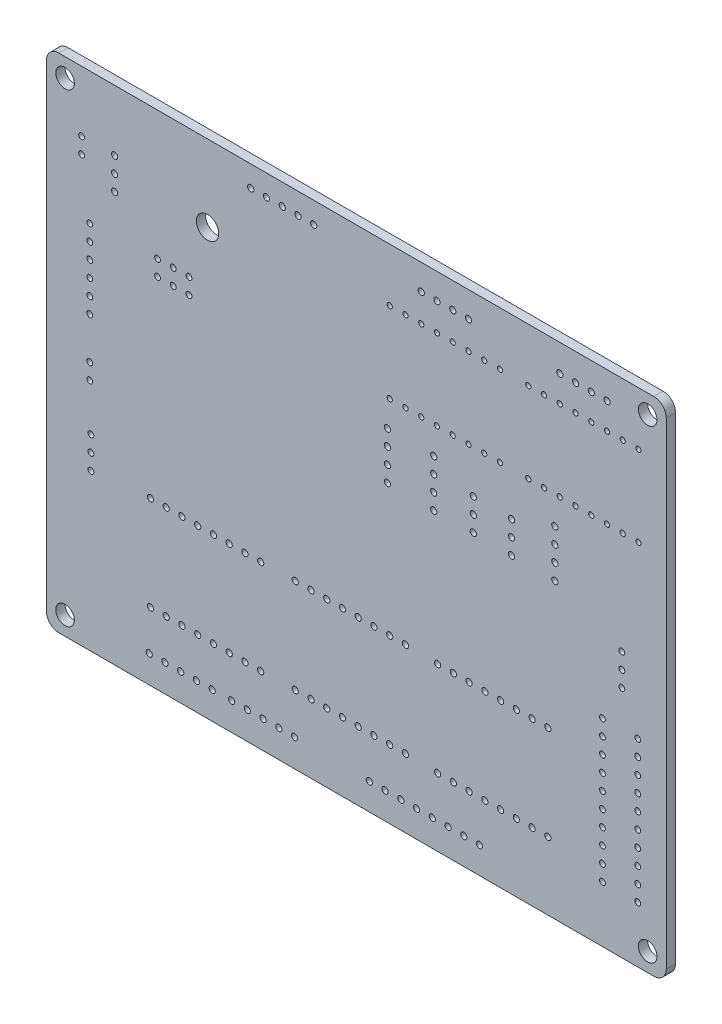
SolidWorks part; units mm, degrees
ref_plane "Plan de face" through (0, 0, 0) normal (0, 0, 1) x (1, 0, 0)
ref_plane "Plan de dessus" through (0, 0, 0) normal (0, 1, 0) x (1, 0, 0)
ref_plane "Plan de droite" through (0, 0, 0) normal (1, 0, 0) x (0, 0, -1)
sketch "Model" plane through (0, 0, 0) normal (0, 0, 1) x (1, 0, 0)
  line L0 (10.1354, 71.1844) -> (11.8626, 71.1844)
  line L1 (10.1354, 71.1844) -> (11.8626, 71.1844)
  line L2 (10.1354, 68.6444) -> (11.8626, 68.6444)
  line L3 (10.1354, 68.6444) -> (11.8626, 68.6444)
  line L4 (10.1354, 66.1044) -> (11.8626, 66.1044)
  line L5 (10.1354, 66.1044) -> (11.8626, 66.1044)
  line L6 (23.4699, 60.4327) -> (23.4699, 60.0433)
  line L7 (23.4699, 60.0433) -> (23.1947, 59.7681)
  line L8 (23.1947, 59.7681) -> (22.8053, 59.7681)
  line L9 (22.8053, 59.7681) -> (22.5301, 60.0433)
  line L10 (22.5301, 60.0433) -> (22.5301, 60.4327)
  line L11 (22.5301, 60.4327) -> (22.8053, 60.7079)
  line L12 (22.8053, 60.7079) -> (23.1947, 60.7079)
  line L13 (23.1947, 60.7079) -> (23.4699, 60.4327)
  line L14 (23.4699, 60.4327) -> (23.4699, 60.0433)
  line L15 (23.4699, 60.4327) -> (23.4699, 60.0433)
  line L16 (23.4699, 60.0433) -> (23.1947, 59.7681)
  line L17 (23.1947, 59.7681) -> (22.8053, 59.7681)
  line L18 (22.8053, 59.7681) -> (22.5301, 60.0433)
  line L19 (22.5301, 60.0433) -> (22.5301, 60.4327)
  line L20 (22.5301, 60.4327) -> (22.8053, 60.7079)
  line L21 (22.8053, 60.7079) -> (23.1947, 60.7079)
  line L22 (23.1947, 60.7079) -> (23.4699, 60.4327)
  line L23 (23.4699, 60.4327) -> (23.4699, 60.0433)
  line L24 (23.4699, 57.8927) -> (23.4699, 57.5033)
  line L25 (23.4699, 57.5033) -> (23.1947, 57.2281)
  line L26 (23.1947, 57.2281) -> (22.8053, 57.2281)
  line L27 (22.8053, 57.2281) -> (22.5301, 57.5033)
  line L28 (22.5301, 57.5033) -> (22.5301, 57.8927)
  line L29 (22.5301, 57.8927) -> (22.8053, 58.1679)
  line L30 (22.8053, 58.1679) -> (23.1947, 58.1679)
  line L31 (23.1947, 58.1679) -> (23.4699, 57.8927)
  line L32 (23.4699, 57.8927) -> (23.4699, 57.5033)
  line L33 (23.4699, 57.8927) -> (23.4699, 57.5033)
  line L34 (23.4699, 57.5033) -> (23.1947, 57.2281)
  line L35 (23.1947, 57.2281) -> (22.8053, 57.2281)
  line L36 (22.8053, 57.2281) -> (22.5301, 57.5033)
  line L37 (22.5301, 57.5033) -> (22.5301, 57.8927)
  line L38 (22.5301, 57.8927) -> (22.8053, 58.1679)
  line L39 (22.8053, 58.1679) -> (23.1947, 58.1679)
  line L40 (23.1947, 58.1679) -> (23.4699, 57.8927)
  line L41 (23.4699, 57.8927) -> (23.4699, 57.5033)
  line L42 (20.9299, 60.4327) -> (20.9299, 60.0433)
  line L43 (20.9299, 60.0433) -> (20.6547, 59.7681)
  line L44 (20.6547, 59.7681) -> (20.2653, 59.7681)
  line L45 (20.2653, 59.7681) -> (19.9901, 60.0433)
  line L46 (19.9901, 60.0433) -> (19.9901, 60.4327)
  line L47 (19.9901, 60.4327) -> (20.2653, 60.7079)
  line L48 (20.2653, 60.7079) -> (20.6547, 60.7079)
  line L49 (20.6547, 60.7079) -> (20.9299, 60.4327)
  line L50 (20.9299, 60.4327) -> (20.9299, 60.0433)
  line L51 (20.9299, 60.4327) -> (20.9299, 60.0433)
  line L52 (20.9299, 60.0433) -> (20.6547, 59.7681)
  line L53 (20.6547, 59.7681) -> (20.2653, 59.7681)
  line L54 (20.2653, 59.7681) -> (19.9901, 60.0433)
  line L55 (19.9901, 60.0433) -> (19.9901, 60.4327)
  line L56 (19.9901, 60.4327) -> (20.2653, 60.7079)
  line L57 (20.2653, 60.7079) -> (20.6547, 60.7079)
  line L58 (20.6547, 60.7079) -> (20.9299, 60.4327)
  line L59 (20.9299, 60.4327) -> (20.9299, 60.0433)
  line L60 (20.9299, 57.8927) -> (20.9299, 57.5033)
  line L61 (20.9299, 57.5033) -> (20.6547, 57.2281)
  line L62 (20.6547, 57.2281) -> (20.2653, 57.2281)
  line L63 (20.2653, 57.2281) -> (19.9901, 57.5033)
  line L64 (19.9901, 57.5033) -> (19.9901, 57.8927)
  line L65 (19.9901, 57.8927) -> (20.2653, 58.1679)
  line L66 (20.2653, 58.1679) -> (20.6547, 58.1679)
  line L67 (20.6547, 58.1679) -> (20.9299, 57.8927)
  line L68 (20.9299, 57.8927) -> (20.9299, 57.5033)
  line L69 (20.9299, 57.8927) -> (20.9299, 57.5033)
  line L70 (20.9299, 57.5033) -> (20.6547, 57.2281)
  line L71 (20.6547, 57.2281) -> (20.2653, 57.2281)
  line L72 (20.2653, 57.2281) -> (19.9901, 57.5033)
  line L73 (19.9901, 57.5033) -> (19.9901, 57.8927)
  line L74 (19.9901, 57.8927) -> (20.2653, 58.1679)
  line L75 (20.2653, 58.1679) -> (20.6547, 58.1679)
  line L76 (20.6547, 58.1679) -> (20.9299, 57.8927)
  line L77 (20.9299, 57.8927) -> (20.9299, 57.5033)
  line L78 (18.3899, 60.4327) -> (18.3899, 60.0433)
  line L79 (18.3899, 60.0433) -> (18.1147, 59.7681)
  line L80 (18.1147, 59.7681) -> (17.7253, 59.7681)
  line L81 (17.7253, 59.7681) -> (17.4501, 60.0433)
  line L82 (17.4501, 60.0433) -> (17.4501, 60.4327)
  line L83 (17.4501, 60.4327) -> (17.7253, 60.7079)
  line L84 (17.7253, 60.7079) -> (18.1147, 60.7079)
  line L85 (18.1147, 60.7079) -> (18.3899, 60.4327)
  line L86 (18.3899, 60.4327) -> (18.3899, 60.0433)
  line L87 (18.3899, 60.4327) -> (18.3899, 60.0433)
  line L88 (18.3899, 60.0433) -> (18.1147, 59.7681)
  line L89 (18.1147, 59.7681) -> (17.7253, 59.7681)
  line L90 (17.7253, 59.7681) -> (17.4501, 60.0433)
  line L91 (17.4501, 60.0433) -> (17.4501, 60.4327)
  line L92 (17.4501, 60.4327) -> (17.7253, 60.7079)
  line L93 (17.7253, 60.7079) -> (18.1147, 60.7079)
  line L94 (18.1147, 60.7079) -> (18.3899, 60.4327)
  line L95 (18.3899, 60.4327) -> (18.3899, 60.0433)
  line L96 (18.3899, 57.8927) -> (18.3899, 57.5033)
  line L97 (18.3899, 57.5033) -> (18.1147, 57.2281)
  line L98 (18.1147, 57.2281) -> (17.7253, 57.2281)
  line L99 (17.7253, 57.2281) -> (17.4501, 57.5033)
  line L100 (17.4501, 57.5033) -> (17.4501, 57.8927)
  line L101 (17.4501, 57.8927) -> (17.7253, 58.1679)
  line L102 (17.7253, 58.1679) -> (18.1147, 58.1679)
  line L103 (18.1147, 58.1679) -> (18.3899, 57.8927)
  line L104 (18.3899, 57.8927) -> (18.3899, 57.5033)
  line L105 (18.3899, 57.8927) -> (18.3899, 57.5033)
  line L106 (18.3899, 57.5033) -> (18.1147, 57.2281)
  line L107 (18.1147, 57.2281) -> (17.7253, 57.2281)
  line L108 (17.7253, 57.2281) -> (17.4501, 57.5033)
  line L109 (17.4501, 57.5033) -> (17.4501, 57.8927)
  line L110 (17.4501, 57.8927) -> (17.7253, 58.1679)
  line L111 (17.7253, 58.1679) -> (18.1147, 58.1679)
  line L112 (18.1147, 58.1679) -> (18.3899, 57.8927)
  line L113 (18.3899, 57.8927) -> (18.3899, 57.5033)
  line L114 (69.875, 5.2358) -> (69.875, 3.3562)
  line L115 (69.875, 5.2358) -> (69.875, 3.3562)
  line L116 (67.335, 5.2358) -> (67.335, 3.3562)
  line L117 (67.335, 5.2358) -> (67.335, 3.3562)
  line L118 (64.795, 5.2358) -> (64.795, 3.3562)
  line L119 (64.795, 5.2358) -> (64.795, 3.3562)
  line L120 (62.255, 5.2358) -> (62.255, 3.3562)
  line L121 (62.255, 5.2358) -> (62.255, 3.3562)
  line L122 (59.715, 5.2358) -> (59.715, 3.3562)
  line L123 (59.715, 5.2358) -> (59.715, 3.3562)
  line L124 (57.175, 5.2358) -> (57.175, 3.3562)
  line L125 (57.175, 5.2358) -> (57.175, 3.3562)
  line L126 (54.635, 5.2358) -> (54.635, 3.3562)
  line L127 (54.635, 5.2358) -> (54.635, 3.3562)
  line L128 (52.095, 5.2358) -> (52.095, 3.3562)
  line L129 (52.095, 5.2358) -> (52.095, 3.3562)
  line L130 (26.74, 5.3628) -> (26.74, 3.4832)
  line L131 (26.74, 5.3628) -> (26.74, 3.4832)
  line L132 (24.2, 5.3628) -> (24.2, 3.4832)
  line L133 (24.2, 5.3628) -> (24.2, 3.4832)
  line L134 (21.66, 5.3628) -> (21.66, 3.4832)
  line L135 (21.66, 5.3628) -> (21.66, 3.4832)
  line L136 (19.12, 5.3628) -> (19.12, 3.4832)
  line L137 (19.12, 5.3628) -> (19.12, 3.4832)
  line L138 (16.58, 5.3628) -> (16.58, 3.4832)
  line L139 (16.58, 5.3628) -> (16.58, 3.4832)
  line L140 (29.873, 3.5272) -> (29.873, 5.4068)
  line L141 (29.873, 3.5272) -> (29.873, 5.4068)
  line L142 (32.413, 3.5272) -> (32.413, 5.4068)
  line L143 (32.413, 3.5272) -> (32.413, 5.4068)
  line L144 (34.953, 3.5272) -> (34.953, 5.4068)
  line L145 (34.953, 3.5272) -> (34.953, 5.4068)
  line L146 (37.493, 3.5272) -> (37.493, 5.4068)
  line L147 (37.493, 3.5272) -> (37.493, 5.4068)
  line L148 (40.033, 3.5272) -> (40.033, 5.4068)
  line L149 (40.033, 3.5272) -> (40.033, 5.4068)
  line L150 (43.1208, 78.534) -> (43.1208, 76.6544)
  line L151 (43.1208, 78.534) -> (43.1208, 76.6544)
  line L152 (40.5808, 78.534) -> (40.5808, 76.6544)
  line L153 (40.5808, 78.534) -> (40.5808, 76.6544)
  line L154 (38.0408, 78.534) -> (38.0408, 76.6544)
  line L155 (38.0408, 78.534) -> (38.0408, 76.6544)
  line L156 (35.5008, 78.534) -> (35.5008, 76.6544)
  line L157 (35.5008, 78.534) -> (35.5008, 76.6544)
  line L158 (32.9608, 78.534) -> (32.9608, 76.6544)
  line L159 (32.9608, 78.534) -> (32.9608, 76.6544)
  line L160 (60.4696, 75.9432) -> (60.4696, 77.8228)
  line L161 (60.4696, 75.9432) -> (60.4696, 77.8228)
  line L162 (63.0096, 75.9432) -> (63.0096, 77.8228)
  line L163 (63.0096, 75.9432) -> (63.0096, 77.8228)
  line L164 (65.5496, 75.9432) -> (65.5496, 77.8228)
  line L165 (65.5496, 75.9432) -> (65.5496, 77.8228)
  line L166 (68.0896, 75.9432) -> (68.0896, 77.8228)
  line L167 (68.0896, 75.9432) -> (68.0896, 77.8228)
  line L168 (74.0942, 52.405) -> (75.9738, 52.405)
  line L169 (74.0942, 52.405) -> (75.9738, 52.405)
  line L170 (74.0942, 49.865) -> (75.9738, 49.865)
  line L171 (74.0942, 49.865) -> (75.9738, 49.865)
  line L172 (74.0942, 47.325) -> (75.9738, 47.325)
  line L173 (74.0942, 47.325) -> (75.9738, 47.325)
  line L174 (67.9322, 52.504) -> (69.8118, 52.504)
  line L175 (67.9322, 52.504) -> (69.8118, 52.504)
  line L176 (67.9322, 49.964) -> (69.8118, 49.964)
  line L177 (67.9322, 49.964) -> (69.8118, 49.964)
  line L178 (67.9322, 47.424) -> (69.8118, 47.424)
  line L179 (67.9322, 47.424) -> (69.8118, 47.424)
  line L180 (54.0772, 55.072) -> (55.9568, 55.072)
  line L181 (54.0772, 55.072) -> (55.9568, 55.072)
  line L182 (54.0772, 52.532) -> (55.9568, 52.532)
  line L183 (54.0772, 52.532) -> (55.9568, 52.532)
  line L184 (54.0772, 49.992) -> (55.9568, 49.992)
  line L185 (54.0772, 49.992) -> (55.9568, 49.992)
  line L186 (54.0772, 47.452) -> (55.9568, 47.452)
  line L187 (54.0772, 47.452) -> (55.9568, 47.452)
  line L188 (61.5402, 54.945) -> (63.4198, 54.945)
  line L189 (61.5402, 54.945) -> (63.4198, 54.945)
  line L190 (61.5402, 52.405) -> (63.4198, 52.405)
  line L191 (61.5402, 52.405) -> (63.4198, 52.405)
  line L192 (61.5402, 49.865) -> (63.4198, 49.865)
  line L193 (61.5402, 49.865) -> (63.4198, 49.865)
  line L194 (61.5402, 47.325) -> (63.4198, 47.325)
  line L195 (61.5402, 47.325) -> (63.4198, 47.325)
  line L196 (81.0822, 54.899) -> (82.9618, 54.899)
  line L197 (81.0822, 54.899) -> (82.9618, 54.899)
  line L198 (81.0822, 52.359) -> (82.9618, 52.359)
  line L199 (81.0822, 52.359) -> (82.9618, 52.359)
  line L200 (81.0822, 49.819) -> (82.9618, 49.819)
  line L201 (81.0822, 49.819) -> (82.9618, 49.819)
  line L202 (81.0822, 47.279) -> (82.9618, 47.279)
  line L203 (81.0822, 47.279) -> (82.9618, 47.279)
  line L204 (82.8285, 75.6892) -> (82.8285, 77.5688)
  line L205 (82.8285, 75.6892) -> (82.8285, 77.5688)
  line L206 (85.3685, 75.6892) -> (85.3685, 77.5688)
  line L207 (85.3685, 75.6892) -> (85.3685, 77.5688)
  line L208 (87.9085, 75.6892) -> (87.9085, 77.5688)
  line L209 (87.9085, 75.6892) -> (87.9085, 77.5688)
  line L210 (90.4485, 75.6892) -> (90.4485, 77.5688)
  line L211 (90.4485, 75.6892) -> (90.4485, 77.5688)
  line L212 (70.733, 10.2422) -> (70.733, 11.6518)
  line L213 (70.733, 10.2422) -> (70.733, 11.6518)
  line L214 (73.273, 10.2422) -> (73.273, 11.6518)
  line L215 (73.273, 10.2422) -> (73.273, 11.6518)
  line L216 (68.193, 25.4822) -> (68.193, 26.8918)
  line L217 (68.193, 25.4822) -> (68.193, 26.8918)
  line L218 (65.653, 25.4822) -> (65.653, 26.8918)
  line L219 (65.653, 25.4822) -> (65.653, 26.8918)
  line L220 (78.353, 10.2422) -> (78.353, 11.6518)
  line L221 (78.353, 10.2422) -> (78.353, 11.6518)
  line L222 (75.813, 10.2422) -> (75.813, 11.6518)
  line L223 (75.813, 10.2422) -> (75.813, 11.6518)
  line L224 (73.273, 25.4822) -> (73.273, 26.8918)
  line L225 (73.273, 25.4822) -> (73.273, 26.8918)
  line L226 (75.813, 25.4822) -> (75.813, 26.8918)
  line L227 (75.813, 25.4822) -> (75.813, 26.8918)
  line L228 (68.193, 10.2422) -> (68.193, 11.6518)
  line L229 (68.193, 10.2422) -> (68.193, 11.6518)
  line L230 (80.893, 10.2422) -> (80.893, 11.6518)
  line L231 (80.893, 10.2422) -> (80.893, 11.6518)
  line L232 (80.893, 25.4822) -> (80.893, 26.8918)
  line L233 (80.893, 25.4822) -> (80.893, 26.8918)
  line L234 (63.113, 25.4822) -> (63.113, 26.8918)
  line L235 (63.113, 25.4822) -> (63.113, 26.8918)
  line L236 (78.353, 25.4822) -> (78.353, 26.8918)
  line L237 (78.353, 25.4822) -> (78.353, 26.8918)
  line L238 (70.733, 25.4822) -> (70.733, 26.8918)
  line L239 (70.733, 25.4822) -> (70.733, 26.8918)
  line L240 (65.653, 10.2422) -> (65.653, 11.6518)
  line L241 (65.653, 10.2422) -> (65.653, 11.6518)
  line L242 (63.113, 10.2422) -> (63.113, 11.6518)
  line L243 (63.113, 10.2422) -> (63.113, 11.6518)
  line L244 (47.759, 10.3692) -> (47.759, 11.7788)
  line L245 (47.759, 10.3692) -> (47.759, 11.7788)
  line L246 (50.299, 10.3692) -> (50.299, 11.7788)
  line L247 (50.299, 10.3692) -> (50.299, 11.7788)
  line L248 (45.219, 25.6092) -> (45.219, 27.0188)
  line L249 (45.219, 25.6092) -> (45.219, 27.0188)
  line L250 (42.679, 25.6092) -> (42.679, 27.0188)
  line L251 (42.679, 25.6092) -> (42.679, 27.0188)
  line L252 (55.379, 10.3692) -> (55.379, 11.7788)
  line L253 (55.379, 10.3692) -> (55.379, 11.7788)
  line L254 (52.839, 10.3692) -> (52.839, 11.7788)
  line L255 (52.839, 10.3692) -> (52.839, 11.7788)
  line L256 (50.299, 25.6092) -> (50.299, 27.0188)
  line L257 (50.299, 25.6092) -> (50.299, 27.0188)
  line L258 (52.839, 25.6092) -> (52.839, 27.0188)
  line L259 (52.839, 25.6092) -> (52.839, 27.0188)
  line L260 (45.219, 10.3692) -> (45.219, 11.7788)
  line L261 (45.219, 10.3692) -> (45.219, 11.7788)
  line L262 (57.919, 10.3692) -> (57.919, 11.7788)
  line L263 (57.919, 10.3692) -> (57.919, 11.7788)
  line L264 (57.919, 25.6092) -> (57.919, 27.0188)
  line L265 (57.919, 25.6092) -> (57.919, 27.0188)
  line L266 (40.139, 25.6092) -> (40.139, 27.0188)
  line L267 (40.139, 25.6092) -> (40.139, 27.0188)
  line L268 (55.379, 25.6092) -> (55.379, 27.0188)
  line L269 (55.379, 25.6092) -> (55.379, 27.0188)
  line L270 (47.759, 25.6092) -> (47.759, 27.0188)
  line L271 (47.759, 25.6092) -> (47.759, 27.0188)
  line L272 (42.679, 10.3692) -> (42.679, 11.7788)
  line L273 (42.679, 10.3692) -> (42.679, 11.7788)
  line L274 (40.139, 10.3692) -> (40.139, 11.7788)
  line L275 (40.139, 10.3692) -> (40.139, 11.7788)
  line L276 (24.404, 10.2422) -> (24.404, 11.6518)
  line L277 (24.404, 10.2422) -> (24.404, 11.6518)
  line L278 (26.944, 10.2422) -> (26.944, 11.6518)
  line L279 (26.944, 10.2422) -> (26.944, 11.6518)
  line L280 (21.864, 25.4822) -> (21.864, 26.8918)
  line L281 (21.864, 25.4822) -> (21.864, 26.8918)
  line L282 (19.324, 25.4822) -> (19.324, 26.8918)
  line L283 (19.324, 25.4822) -> (19.324, 26.8918)
  line L284 (32.024, 10.2422) -> (32.024, 11.6518)
  line L285 (32.024, 10.2422) -> (32.024, 11.6518)
  line L286 (29.484, 10.2422) -> (29.484, 11.6518)
  line L287 (29.484, 10.2422) -> (29.484, 11.6518)
  line L288 (26.944, 25.4822) -> (26.944, 26.8918)
  line L289 (26.944, 25.4822) -> (26.944, 26.8918)
  line L290 (29.484, 25.4822) -> (29.484, 26.8918)
  line L291 (29.484, 25.4822) -> (29.484, 26.8918)
  line L292 (21.864, 10.2422) -> (21.864, 11.6518)
  line L293 (21.864, 10.2422) -> (21.864, 11.6518)
  line L294 (34.564, 10.2422) -> (34.564, 11.6518)
  line L295 (34.564, 10.2422) -> (34.564, 11.6518)
  line L296 (34.564, 25.4822) -> (34.564, 26.8918)
  line L297 (34.564, 25.4822) -> (34.564, 26.8918)
  line L298 (16.784, 25.4822) -> (16.784, 26.8918)
  line L299 (16.784, 25.4822) -> (16.784, 26.8918)
  line L300 (32.024, 25.4822) -> (32.024, 26.8918)
  line L301 (32.024, 25.4822) -> (32.024, 26.8918)
  line L302 (24.404, 25.4822) -> (24.404, 26.8918)
  line L303 (24.404, 25.4822) -> (24.404, 26.8918)
  line L304 (19.324, 10.2422) -> (19.324, 11.6518)
  line L305 (19.324, 10.2422) -> (19.324, 11.6518)
  line L306 (16.784, 10.2422) -> (16.784, 11.6518)
  line L307 (16.784, 10.2422) -> (16.784, 11.6518)
  line L308 (50.675, 48.5366) -> (50.675, 48.7454)
  line L309 (50.675, 48.7454) -> (50.8226, 48.893)
  line L310 (50.8226, 48.893) -> (51.0314, 48.893)
  line L311 (51.0314, 48.893) -> (51.179, 48.7454)
  line L312 (51.179, 48.7454) -> (51.179, 48.5366)
  line L313 (51.179, 48.5366) -> (51.0314, 48.389)
  line L314 (51.0314, 48.389) -> (50.8226, 48.389)
  line L315 (50.8226, 48.389) -> (50.675, 48.5366)
  line L316 (50.675, 48.5366) -> (50.675, 48.7454)
  line L317 (47.246, 51.2036) -> (47.246, 51.4124)
  line L318 (47.246, 51.4124) -> (47.3936, 51.56)
  line L319 (47.3936, 51.56) -> (47.6024, 51.56)
  line L320 (47.6024, 51.56) -> (47.75, 51.4124)
  line L321 (47.75, 51.4124) -> (47.75, 51.2036)
  line L322 (47.75, 51.2036) -> (47.6024, 51.056)
  line L323 (47.6024, 51.056) -> (47.3936, 51.056)
  line L324 (47.3936, 51.056) -> (47.246, 51.2036)
  line L325 (47.246, 51.2036) -> (47.246, 51.4124)
  line L326 (21.592, 34.0586) -> (21.592, 34.2674)
  line L327 (21.592, 34.2674) -> (21.7396, 34.415)
  line L328 (21.7396, 34.415) -> (21.9484, 34.415)
  line L329 (21.9484, 34.415) -> (22.096, 34.2674)
  line L330 (22.096, 34.2674) -> (22.096, 34.0586)
  line L331 (22.096, 34.0586) -> (21.9484, 33.911)
  line L332 (21.9484, 33.911) -> (21.7396, 33.911)
  line L333 (21.7396, 33.911) -> (21.592, 34.0586)
  line L334 (21.592, 34.0586) -> (21.592, 34.2674)
  line L335 (43.817, 40.1546) -> (43.817, 40.3634)
  line L336 (43.817, 40.3634) -> (43.9646, 40.511)
  line L337 (43.9646, 40.511) -> (44.1734, 40.511)
  line L338 (44.1734, 40.511) -> (44.321, 40.3634)
  line L339 (44.321, 40.3634) -> (44.321, 40.1546)
  line L340 (44.321, 40.1546) -> (44.1734, 40.007)
  line L341 (44.1734, 40.007) -> (43.9646, 40.007)
  line L342 (43.9646, 40.007) -> (43.817, 40.1546)
  line L343 (43.817, 40.1546) -> (43.817, 40.3634)
  line L344 (52.58, 44.2186) -> (52.58, 44.4274)
  line L345 (52.58, 44.4274) -> (52.7276, 44.575)
  line L346 (52.7276, 44.575) -> (52.9364, 44.575)
  line L347 (52.9364, 44.575) -> (53.084, 44.4274)
  line L348 (53.084, 44.4274) -> (53.084, 44.2186)
  line L349 (53.084, 44.2186) -> (52.9364, 44.071)
  line L350 (52.9364, 44.071) -> (52.7276, 44.071)
  line L351 (52.7276, 44.071) -> (52.58, 44.2186)
  line L352 (52.58, 44.2186) -> (52.58, 44.4274)
  line L353 (52.58, 42.6946) -> (52.58, 42.9034)
  line L354 (52.58, 42.9034) -> (52.7276, 43.051)
  line L355 (52.7276, 43.051) -> (52.9364, 43.051)
  line L356 (52.9364, 43.051) -> (53.084, 42.9034)
  line L357 (53.084, 42.9034) -> (53.084, 42.6946)
  line L358 (53.084, 42.6946) -> (52.9364, 42.547)
  line L359 (52.9364, 42.547) -> (52.7276, 42.547)
  line L360 (52.7276, 42.547) -> (52.58, 42.6946)
  line L361 (52.58, 42.6946) -> (52.58, 42.9034)
  line L362 (43.817, 37.9956) -> (43.817, 38.2044)
  line L363 (43.817, 38.2044) -> (43.9646, 38.352)
  line L364 (43.9646, 38.352) -> (44.1734, 38.352)
  line L365 (44.1734, 38.352) -> (44.321, 38.2044)
  line L366 (44.321, 38.2044) -> (44.321, 37.9956)
  line L367 (44.321, 37.9956) -> (44.1734, 37.848)
  line L368 (44.1734, 37.848) -> (43.9646, 37.848)
  line L369 (43.9646, 37.848) -> (43.817, 37.9956)
  line L370 (43.817, 37.9956) -> (43.817, 38.2044)
  line L371 (49.151, 39.9006) -> (49.151, 40.1094)
  line L372 (49.151, 40.1094) -> (49.2986, 40.257)
  line L373 (49.2986, 40.257) -> (49.5074, 40.257)
  line L374 (49.5074, 40.257) -> (49.655, 40.1094)
  line L375 (49.655, 40.1094) -> (49.655, 39.9006)
  line L376 (49.655, 39.9006) -> (49.5074, 39.753)
  line L377 (49.5074, 39.753) -> (49.2986, 39.753)
  line L378 (49.2986, 39.753) -> (49.151, 39.9006)
  line L379 (49.151, 39.9006) -> (49.151, 40.1094)
  line L380 (48.643, 49.4256) -> (48.643, 49.6344)
  line L381 (48.643, 49.6344) -> (48.7906, 49.782)
  line L382 (48.7906, 49.782) -> (48.9994, 49.782)
  line L383 (48.9994, 49.782) -> (49.147, 49.6344)
  line L384 (49.147, 49.6344) -> (49.147, 49.4256)
  line L385 (49.147, 49.4256) -> (48.9994, 49.278)
  line L386 (48.9994, 49.278) -> (48.7906, 49.278)
  line L387 (48.7906, 49.278) -> (48.643, 49.4256)
  line L388 (48.643, 49.4256) -> (48.643, 49.6344)
  line L389 (31.879, 17.4216) -> (31.879, 17.6304)
  line L390 (31.879, 17.6304) -> (32.0266, 17.778)
  line L391 (32.0266, 17.778) -> (32.2354, 17.778)
  line L392 (32.2354, 17.778) -> (32.383, 17.6304)
  line L393 (32.383, 17.6304) -> (32.383, 17.4216)
  line L394 (32.383, 17.4216) -> (32.2354, 17.274)
  line L395 (32.2354, 17.274) -> (32.0266, 17.274)
  line L396 (32.0266, 17.274) -> (31.879, 17.4216)
  line L397 (31.879, 17.4216) -> (31.879, 17.6304)
  line L398 (4.066, 41.5516) -> (4.066, 41.7604)
  line L399 (4.066, 41.7604) -> (4.2136, 41.908)
  line L400 (4.2136, 41.908) -> (4.4224, 41.908)
  line L401 (4.4224, 41.908) -> (4.57, 41.7604)
  line L402 (4.57, 41.7604) -> (4.57, 41.5516)
  line L403 (4.57, 41.5516) -> (4.4224, 41.404)
  line L404 (4.4224, 41.404) -> (4.2136, 41.404)
  line L405 (4.2136, 41.404) -> (4.066, 41.5516)
  line L406 (4.066, 41.5516) -> (4.066, 41.7604)
  line L407 (4.066, 51.3306) -> (4.066, 51.5394)
  line L408 (4.066, 51.5394) -> (4.2136, 51.687)
  line L409 (4.2136, 51.687) -> (4.4224, 51.687)
  line L410 (4.4224, 51.687) -> (4.57, 51.5394)
  line L411 (4.57, 51.5394) -> (4.57, 51.3306)
  line L412 (4.57, 51.3306) -> (4.4224, 51.183)
  line L413 (4.4224, 51.183) -> (4.2136, 51.183)
  line L414 (4.2136, 51.183) -> (4.066, 51.3306)
  line L415 (4.066, 51.3306) -> (4.066, 51.5394)
  line L416 (51.691, 45.9966) -> (51.691, 46.2054)
  line L417 (51.691, 46.2054) -> (51.8386, 46.353)
  line L418 (51.8386, 46.353) -> (52.0474, 46.353)
  line L419 (52.0474, 46.353) -> (52.195, 46.2054)
  line L420 (52.195, 46.2054) -> (52.195, 45.9966)
  line L421 (52.195, 45.9966) -> (52.0474, 45.849)
  line L422 (52.0474, 45.849) -> (51.8386, 45.849)
  line L423 (51.8386, 45.849) -> (51.691, 45.9966)
  line L424 (51.691, 45.9966) -> (51.691, 46.2054)
  line L425 (50.421, 45.9966) -> (50.421, 46.2054)
  line L426 (50.421, 46.2054) -> (50.5686, 46.353)
  line L427 (50.5686, 46.353) -> (50.7774, 46.353)
  line L428 (50.7774, 46.353) -> (50.925, 46.2054)
  line L429 (50.925, 46.2054) -> (50.925, 45.9966)
  line L430 (50.925, 45.9966) -> (50.7774, 45.849)
  line L431 (50.7774, 45.849) -> (50.5686, 45.849)
  line L432 (50.5686, 45.849) -> (50.421, 45.9966)
  line L433 (50.421, 45.9966) -> (50.421, 46.2054)
  line L434 (34.546, 54.1246) -> (34.546, 54.3334)
  line L435 (34.546, 54.3334) -> (34.6936, 54.481)
  line L436 (34.6936, 54.481) -> (34.9024, 54.481)
  line L437 (34.9024, 54.481) -> (35.05, 54.3334)
  line L438 (35.05, 54.3334) -> (35.05, 54.1246)
  line L439 (35.05, 54.1246) -> (34.9024, 53.977)
  line L440 (34.9024, 53.977) -> (34.6936, 53.977)
  line L441 (34.6936, 53.977) -> (34.546, 54.1246)
  line L442 (34.546, 54.1246) -> (34.546, 54.3334)
  line L443 (21.338, 52.3466) -> (21.338, 52.5554)
  line L444 (21.338, 52.5554) -> (21.4856, 52.703)
  line L445 (21.4856, 52.703) -> (21.6944, 52.703)
  line L446 (21.6944, 52.703) -> (21.842, 52.5554)
  line L447 (21.842, 52.5554) -> (21.842, 52.3466)
  line L448 (21.842, 52.3466) -> (21.6944, 52.199)
  line L449 (21.6944, 52.199) -> (21.4856, 52.199)
  line L450 (21.4856, 52.199) -> (21.338, 52.3466)
  line L451 (21.338, 52.3466) -> (21.338, 52.5554)
  line L452 (1.971, 77.5736) -> (1.971, 78.4264)
  line L453 (1.971, 78.4264) -> (2.5736, 79.029)
  line L454 (2.5736, 79.029) -> (3.4264, 79.029)
  line L455 (3.4264, 79.029) -> (4.029, 78.4264)
  line L456 (4.029, 78.4264) -> (4.029, 77.5736)
  line L457 (4.029, 77.5736) -> (3.4264, 76.971)
  line L458 (3.4264, 76.971) -> (2.5736, 76.971)
  line L459 (2.5736, 76.971) -> (1.971, 77.5736)
  line L460 (1.971, 77.5736) -> (1.971, 78.4264)
  line L461 (95.971, 77.5736) -> (95.971, 78.4264)
  line L462 (95.971, 78.4264) -> (96.5736, 79.029)
  line L463 (96.5736, 79.029) -> (97.4264, 79.029)
  line L464 (97.4264, 79.029) -> (98.029, 78.4264)
  line L465 (98.029, 78.4264) -> (98.029, 77.5736)
  line L466 (98.029, 77.5736) -> (97.4264, 76.971)
  line L467 (97.4264, 76.971) -> (96.5736, 76.971)
  line L468 (96.5736, 76.971) -> (95.971, 77.5736)
  line L469 (95.971, 77.5736) -> (95.971, 78.4264)
  line L470 (1.971, 2.5736) -> (1.971, 3.4264)
  line L471 (1.971, 3.4264) -> (2.5736, 4.029)
  line L472 (2.5736, 4.029) -> (3.4264, 4.029)
  line L473 (3.4264, 4.029) -> (4.029, 3.4264)
  line L474 (4.029, 3.4264) -> (4.029, 2.5736)
  line L475 (4.029, 2.5736) -> (3.4264, 1.971)
  line L476 (3.4264, 1.971) -> (2.5736, 1.971)
  line L477 (2.5736, 1.971) -> (1.971, 2.5736)
  line L478 (1.971, 2.5736) -> (1.971, 3.4264)
  line L479 (95.971, 2.5736) -> (95.971, 3.4264)
  line L480 (95.971, 3.4264) -> (96.5736, 4.029)
  line L481 (96.5736, 4.029) -> (97.4264, 4.029)
  line L482 (97.4264, 4.029) -> (98.029, 3.4264)
  line L483 (98.029, 3.4264) -> (98.029, 2.5736)
  line L484 (98.029, 2.5736) -> (97.4264, 1.971)
  line L485 (97.4264, 1.971) -> (96.5736, 1.971)
  line L486 (96.5736, 1.971) -> (95.971, 2.5736)
  line L487 (95.971, 2.5736) -> (95.971, 3.4264)
  line L488 (24.854, 68.2702) -> (24.854, 69.1438)
  line L489 (24.854, 69.1438) -> (25.4712, 69.761)
  line L490 (25.4712, 69.761) -> (26.3448, 69.761)
  line L491 (26.3448, 69.761) -> (26.962, 69.1438)
  line L492 (26.962, 69.1438) -> (26.962, 68.2702)
  line L493 (26.962, 68.2702) -> (26.3448, 67.653)
  line L494 (26.3448, 67.653) -> (25.4712, 67.653)
  line L495 (25.4712, 67.653) -> (24.854, 68.2702)
  line L496 (24.854, 68.2702) -> (24.854, 69.1438)
  line L497 (42.42, 40.1546) -> (42.42, 40.3634)
  line L498 (42.42, 40.3634) -> (42.5676, 40.511)
  line L499 (42.5676, 40.511) -> (42.7764, 40.511)
  line L500 (42.7764, 40.511) -> (42.924, 40.3634)
  line L501 (42.924, 40.3634) -> (42.924, 40.1546)
  line L502 (42.924, 40.1546) -> (42.7764, 40.007)
  line L503 (42.7764, 40.007) -> (42.5676, 40.007)
  line L504 (42.5676, 40.007) -> (42.42, 40.1546)
  line L505 (42.42, 40.1546) -> (42.42, 40.3634)
  line L506 (45.341, 52.8546) -> (45.341, 53.0634)
  line L507 (45.341, 53.0634) -> (45.4886, 53.211)
  line L508 (45.4886, 53.211) -> (45.6974, 53.211)
  line L509 (45.6974, 53.211) -> (45.845, 53.0634)
  line L510 (45.845, 53.0634) -> (45.845, 52.8546)
  line L511 (45.845, 52.8546) -> (45.6974, 52.707)
  line L512 (45.6974, 52.707) -> (45.4886, 52.707)
  line L513 (45.4886, 52.707) -> (45.341, 52.8546)
  line L514 (45.341, 52.8546) -> (45.341, 53.0634)
  line L515 (39.88, 40.1546) -> (39.88, 40.3634)
  line L516 (39.88, 40.3634) -> (40.0276, 40.511)
  line L517 (40.0276, 40.511) -> (40.2364, 40.511)
  line L518 (40.2364, 40.511) -> (40.384, 40.3634)
  line L519 (40.384, 40.3634) -> (40.384, 40.1546)
  line L520 (40.384, 40.1546) -> (40.2364, 40.007)
  line L521 (40.2364, 40.007) -> (40.0276, 40.007)
  line L522 (40.0276, 40.007) -> (39.88, 40.1546)
  line L523 (39.88, 40.1546) -> (39.88, 40.3634)
  line L524 (41.15, 40.1546) -> (41.15, 40.3634)
  line L525 (41.15, 40.3634) -> (41.2976, 40.511)
  line L526 (41.2976, 40.511) -> (41.5064, 40.511)
  line L527 (41.5064, 40.511) -> (41.654, 40.3634)
  line L528 (41.654, 40.3634) -> (41.654, 40.1546)
  line L529 (41.654, 40.1546) -> (41.5064, 40.007)
  line L530 (41.5064, 40.007) -> (41.2976, 40.007)
  line L531 (41.2976, 40.007) -> (41.15, 40.1546)
  line L532 (41.15, 40.1546) -> (41.15, 40.3634)
  line L533 (33.149, 48.9176) -> (33.149, 49.1264)
  line L534 (33.149, 49.1264) -> (33.2966, 49.274)
  line L535 (33.2966, 49.274) -> (33.5054, 49.274)
  line L536 (33.5054, 49.274) -> (33.653, 49.1264)
  line L537 (33.653, 49.1264) -> (33.653, 48.9176)
  line L538 (33.653, 48.9176) -> (33.5054, 48.77)
  line L539 (33.5054, 48.77) -> (33.2966, 48.77)
  line L540 (33.2966, 48.77) -> (33.149, 48.9176)
  line L541 (33.149, 48.9176) -> (33.149, 49.1264)
  line L542 (34.038, 47.7746) -> (34.038, 47.9834)
  line L543 (34.038, 47.9834) -> (34.1856, 48.131)
  line L544 (34.1856, 48.131) -> (34.3944, 48.131)
  line L545 (34.3944, 48.131) -> (34.542, 47.9834)
  line L546 (34.542, 47.9834) -> (34.542, 47.7746)
  line L547 (34.542, 47.7746) -> (34.3944, 47.627)
  line L548 (34.3944, 47.627) -> (34.1856, 47.627)
  line L549 (34.1856, 47.627) -> (34.038, 47.7746)
  line L550 (34.038, 47.7746) -> (34.038, 47.9834)
  line L551 (45.849, 65.4276) -> (45.849, 65.6364)
  line L552 (45.849, 65.6364) -> (45.9966, 65.784)
  line L553 (45.9966, 65.784) -> (46.2054, 65.784)
  line L554 (46.2054, 65.784) -> (46.353, 65.6364)
  line L555 (46.353, 65.6364) -> (46.353, 65.4276)
  line L556 (46.353, 65.4276) -> (46.2054, 65.28)
  line L557 (46.2054, 65.28) -> (45.9966, 65.28)
  line L558 (45.9966, 65.28) -> (45.849, 65.4276)
  line L559 (45.849, 65.4276) -> (45.849, 65.6364)
  line L560 (45.214, 57.6806) -> (45.214, 57.8894)
  line L561 (45.214, 57.8894) -> (45.3616, 58.037)
  line L562 (45.3616, 58.037) -> (45.5704, 58.037)
  line L563 (45.5704, 58.037) -> (45.718, 57.8894)
  line L564 (45.718, 57.8894) -> (45.718, 57.6806)
  line L565 (45.718, 57.6806) -> (45.5704, 57.533)
  line L566 (45.5704, 57.533) -> (45.3616, 57.533)
  line L567 (45.3616, 57.533) -> (45.214, 57.6806)
  line L568 (45.214, 57.6806) -> (45.214, 57.8894)
  line L569 (38.356, 56.5376) -> (38.356, 56.7464)
  line L570 (38.356, 56.7464) -> (38.5036, 56.894)
  line L571 (38.5036, 56.894) -> (38.7124, 56.894)
  line L572 (38.7124, 56.894) -> (38.86, 56.7464)
  line L573 (38.86, 56.7464) -> (38.86, 56.5376)
  line L574 (38.86, 56.5376) -> (38.7124, 56.39)
  line L575 (38.7124, 56.39) -> (38.5036, 56.39)
  line L576 (38.5036, 56.39) -> (38.356, 56.5376)
  line L577 (38.356, 56.5376) -> (38.356, 56.7464)
  line L578 (38.102, 33.9316) -> (38.102, 34.1404)
  line L579 (38.102, 34.1404) -> (38.2496, 34.288)
  line L580 (38.2496, 34.288) -> (38.4584, 34.288)
  line L581 (38.4584, 34.288) -> (38.606, 34.1404)
  line L582 (38.606, 34.1404) -> (38.606, 33.9316)
  line L583 (38.606, 33.9316) -> (38.4584, 33.784)
  line L584 (38.4584, 33.784) -> (38.2496, 33.784)
  line L585 (38.2496, 33.784) -> (38.102, 33.9316)
  line L586 (38.102, 33.9316) -> (38.102, 34.1404)
  line L587 (96.395, 54.7596) -> (96.395, 54.9684)
  line L588 (96.395, 54.9684) -> (96.5426, 55.116)
  line L589 (96.5426, 55.116) -> (96.7514, 55.116)
  line L590 (96.7514, 55.116) -> (96.899, 54.9684)
  line L591 (96.899, 54.9684) -> (96.899, 54.7596)
  line L592 (96.899, 54.7596) -> (96.7514, 54.612)
  line L593 (96.7514, 54.612) -> (96.5426, 54.612)
  line L594 (96.5426, 54.612) -> (96.395, 54.7596)
  line L595 (96.395, 54.7596) -> (96.395, 54.9684)
  line L596 (34.673, 55.9026) -> (34.673, 56.1114)
  line L597 (34.673, 56.1114) -> (34.8206, 56.259)
  line L598 (34.8206, 56.259) -> (35.0294, 56.259)
  line L599 (35.0294, 56.259) -> (35.177, 56.1114)
  line L600 (35.177, 56.1114) -> (35.177, 55.9026)
  line L601 (35.177, 55.9026) -> (35.0294, 55.755)
  line L602 (35.0294, 55.755) -> (34.8206, 55.755)
  line L603 (34.8206, 55.755) -> (34.673, 55.9026)
  line L604 (34.673, 55.9026) -> (34.673, 56.1114)
  line L605 (32.514, 41.9326) -> (32.514, 42.1414)
  line L606 (32.514, 42.1414) -> (32.6616, 42.289)
  line L607 (32.6616, 42.289) -> (32.8704, 42.289)
  line L608 (32.8704, 42.289) -> (33.018, 42.1414)
  line L609 (33.018, 42.1414) -> (33.018, 41.9326)
  line L610 (33.018, 41.9326) -> (32.8704, 41.785)
  line L611 (32.8704, 41.785) -> (32.6616, 41.785)
  line L612 (32.6616, 41.785) -> (32.514, 41.9326)
  line L613 (32.514, 41.9326) -> (32.514, 42.1414)
  line L614 (33.657, 41.1706) -> (33.657, 41.3794)
  line L615 (33.657, 41.3794) -> (33.8046, 41.527)
  line L616 (33.8046, 41.527) -> (34.0134, 41.527)
  line L617 (34.0134, 41.527) -> (34.161, 41.3794)
  line L618 (34.161, 41.3794) -> (34.161, 41.1706)
  line L619 (34.161, 41.1706) -> (34.0134, 41.023)
  line L620 (34.0134, 41.023) -> (33.8046, 41.023)
  line L621 (33.8046, 41.023) -> (33.657, 41.1706)
  line L622 (33.657, 41.1706) -> (33.657, 41.3794)
  line L623 (13.337, 44.9806) -> (13.337, 45.1894)
  line L624 (13.337, 45.1894) -> (13.4846, 45.337)
  line L625 (13.4846, 45.337) -> (13.6934, 45.337)
  line L626 (13.6934, 45.337) -> (13.841, 45.1894)
  line L627 (13.841, 45.1894) -> (13.841, 44.9806)
  line L628 (13.841, 44.9806) -> (13.6934, 44.833)
  line L629 (13.6934, 44.833) -> (13.4846, 44.833)
  line L630 (13.4846, 44.833) -> (13.337, 44.9806)
  line L631 (13.337, 44.9806) -> (13.337, 45.1894)
  line L632 (65.788, 19.9616) -> (65.788, 20.1704)
  line L633 (65.788, 20.1704) -> (65.9356, 20.318)
  line L634 (65.9356, 20.318) -> (66.1444, 20.318)
  line L635 (66.1444, 20.318) -> (66.292, 20.1704)
  line L636 (66.292, 20.1704) -> (66.292, 19.9616)
  line L637 (66.292, 19.9616) -> (66.1444, 19.814)
  line L638 (66.1444, 19.814) -> (65.9356, 19.814)
  line L639 (65.9356, 19.814) -> (65.788, 19.9616)
  line L640 (65.788, 19.9616) -> (65.788, 20.1704)
  line L641 (14.607, 44.9806) -> (14.607, 45.1894)
  line L642 (14.607, 45.1894) -> (14.7546, 45.337)
  line L643 (14.7546, 45.337) -> (14.9634, 45.337)
  line L644 (14.9634, 45.337) -> (15.111, 45.1894)
  line L645 (15.111, 45.1894) -> (15.111, 44.9806)
  line L646 (15.111, 44.9806) -> (14.9634, 44.833)
  line L647 (14.9634, 44.833) -> (14.7546, 44.833)
  line L648 (14.7546, 44.833) -> (14.607, 44.9806)
  line L649 (14.607, 44.9806) -> (14.607, 45.1894)
  line L650 (45.087, 19.7076) -> (45.087, 19.9164)
  line L651 (45.087, 19.9164) -> (45.2346, 20.064)
  line L652 (45.2346, 20.064) -> (45.4434, 20.064)
  line L653 (45.4434, 20.064) -> (45.591, 19.9164)
  line L654 (45.591, 19.9164) -> (45.591, 19.7076)
  line L655 (45.591, 19.7076) -> (45.4434, 19.56)
  line L656 (45.4434, 19.56) -> (45.2346, 19.56)
  line L657 (45.2346, 19.56) -> (45.087, 19.7076)
  line L658 (45.087, 19.7076) -> (45.087, 19.9164)
  line L659 (24.894, 52.3466) -> (24.894, 52.5554)
  line L660 (24.894, 52.5554) -> (25.0416, 52.703)
  line L661 (25.0416, 52.703) -> (25.2504, 52.703)
  line L662 (25.2504, 52.703) -> (25.398, 52.5554)
  line L663 (25.398, 52.5554) -> (25.398, 52.3466)
  line L664 (25.398, 52.3466) -> (25.2504, 52.199)
  line L665 (25.2504, 52.199) -> (25.0416, 52.199)
  line L666 (25.0416, 52.199) -> (24.894, 52.3466)
  line L667 (24.894, 52.3466) -> (24.894, 52.5554)
  line L668 (12.448, 24.1526) -> (12.448, 24.3614)
  line L669 (12.448, 24.3614) -> (12.5956, 24.509)
  line L670 (12.5956, 24.509) -> (12.8044, 24.509)
  line L671 (12.8044, 24.509) -> (12.952, 24.3614)
  line L672 (12.952, 24.3614) -> (12.952, 24.1526)
  line L673 (12.952, 24.1526) -> (12.8044, 24.005)
  line L674 (12.8044, 24.005) -> (12.5956, 24.005)
  line L675 (12.5956, 24.005) -> (12.448, 24.1526)
  line L676 (12.448, 24.1526) -> (12.448, 24.3614)
  line L677 (27.815, 42.6946) -> (27.815, 42.9034)
  line L678 (27.815, 42.9034) -> (27.9626, 43.051)
  line L679 (27.9626, 43.051) -> (28.1714, 43.051)
  line L680 (28.1714, 43.051) -> (28.319, 42.9034)
  line L681 (28.319, 42.9034) -> (28.319, 42.6946)
  line L682 (28.319, 42.6946) -> (28.1714, 42.547)
  line L683 (28.1714, 42.547) -> (27.9626, 42.547)
  line L684 (27.9626, 42.547) -> (27.815, 42.6946)
  line L685 (27.815, 42.6946) -> (27.815, 42.9034)
  line L686 (37.086, 42.9486) -> (37.086, 43.1574)
  line L687 (37.086, 43.1574) -> (37.2336, 43.305)
  line L688 (37.2336, 43.305) -> (37.4424, 43.305)
  line L689 (37.4424, 43.305) -> (37.59, 43.1574)
  line L690 (37.59, 43.1574) -> (37.59, 42.9486)
  line L691 (37.59, 42.9486) -> (37.4424, 42.801)
  line L692 (37.4424, 42.801) -> (37.2336, 42.801)
  line L693 (37.2336, 42.801) -> (37.086, 42.9486)
  line L694 (37.086, 42.9486) -> (37.086, 43.1574)
  line L695 (26.418, 42.6946) -> (26.418, 42.9034)
  line L696 (26.418, 42.9034) -> (26.5656, 43.051)
  line L697 (26.5656, 43.051) -> (26.7744, 43.051)
  line L698 (26.7744, 43.051) -> (26.922, 42.9034)
  line L699 (26.922, 42.9034) -> (26.922, 42.6946)
  line L700 (26.922, 42.6946) -> (26.7744, 42.547)
  line L701 (26.7744, 42.547) -> (26.5656, 42.547)
  line L702 (26.5656, 42.547) -> (26.418, 42.6946)
  line L703 (26.418, 42.6946) -> (26.418, 42.9034)
  line L704 (74.932, 62.8876) -> (74.932, 63.0964)
  line L705 (74.932, 63.0964) -> (75.0796, 63.244)
  line L706 (75.0796, 63.244) -> (75.2884, 63.244)
  line L707 (75.2884, 63.244) -> (75.436, 63.0964)
  line L708 (75.436, 63.0964) -> (75.436, 62.8876)
  line L709 (75.436, 62.8876) -> (75.2884, 62.74)
  line L710 (75.2884, 62.74) -> (75.0796, 62.74)
  line L711 (75.0796, 62.74) -> (74.932, 62.8876)
  line L712 (74.932, 62.8876) -> (74.932, 63.0964)
  line L713 (35.689, 42.5676) -> (35.689, 42.7764)
  line L714 (35.689, 42.7764) -> (35.8366, 42.924)
  line L715 (35.8366, 42.924) -> (36.0454, 42.924)
  line L716 (36.0454, 42.924) -> (36.193, 42.7764)
  line L717 (36.193, 42.7764) -> (36.193, 42.5676)
  line L718 (36.193, 42.5676) -> (36.0454, 42.42)
  line L719 (36.0454, 42.42) -> (35.8366, 42.42)
  line L720 (35.8366, 42.42) -> (35.689, 42.5676)
  line L721 (35.689, 42.5676) -> (35.689, 42.7764)
  line L722 (28.831, 43.5836) -> (28.831, 43.7924)
  line L723 (28.831, 43.7924) -> (28.9786, 43.94)
  line L724 (28.9786, 43.94) -> (29.1874, 43.94)
  line L725 (29.1874, 43.94) -> (29.335, 43.7924)
  line L726 (29.335, 43.7924) -> (29.335, 43.5836)
  line L727 (29.335, 43.5836) -> (29.1874, 43.436)
  line L728 (29.1874, 43.436) -> (28.9786, 43.436)
  line L729 (28.9786, 43.436) -> (28.831, 43.5836)
  line L730 (28.831, 43.5836) -> (28.831, 43.7924)
  line L731 (37.975, 43.9646) -> (37.975, 44.1734)
  line L732 (37.975, 44.1734) -> (38.1226, 44.321)
  line L733 (38.1226, 44.321) -> (38.3314, 44.321)
  line L734 (38.3314, 44.321) -> (38.479, 44.1734)
  line L735 (38.479, 44.1734) -> (38.479, 43.9646)
  line L736 (38.479, 43.9646) -> (38.3314, 43.817)
  line L737 (38.3314, 43.817) -> (38.1226, 43.817)
  line L738 (38.1226, 43.817) -> (37.975, 43.9646)
  line L739 (37.975, 43.9646) -> (37.975, 44.1734)
  line L740 (44.706, 63.0146) -> (44.706, 63.2234)
  line L741 (44.706, 63.2234) -> (44.8536, 63.371)
  line L742 (44.8536, 63.371) -> (45.0624, 63.371)
  line L743 (45.0624, 63.371) -> (45.21, 63.2234)
  line L744 (45.21, 63.2234) -> (45.21, 63.0146)
  line L745 (45.21, 63.0146) -> (45.0624, 62.867)
  line L746 (45.0624, 62.867) -> (44.8536, 62.867)
  line L747 (44.8536, 62.867) -> (44.706, 63.0146)
  line L748 (44.706, 63.0146) -> (44.706, 63.2234)
  line L749 (46.103, 56.5376) -> (46.103, 56.7464)
  line L750 (46.103, 56.7464) -> (46.2506, 56.894)
  line L751 (46.2506, 56.894) -> (46.4594, 56.894)
  line L752 (46.4594, 56.894) -> (46.607, 56.7464)
  line L753 (46.607, 56.7464) -> (46.607, 56.5376)
  line L754 (46.607, 56.5376) -> (46.4594, 56.39)
  line L755 (46.4594, 56.39) -> (46.2506, 56.39)
  line L756 (46.2506, 56.39) -> (46.103, 56.5376)
  line L757 (46.103, 56.5376) -> (46.103, 56.7464)
  line L758 (38.229, 55.0136) -> (38.229, 55.2224)
  line L759 (38.229, 55.2224) -> (38.3766, 55.37)
  line L760 (38.3766, 55.37) -> (38.5854, 55.37)
  line L761 (38.5854, 55.37) -> (38.733, 55.2224)
  line L762 (38.733, 55.2224) -> (38.733, 55.0136)
  line L763 (38.733, 55.0136) -> (38.5854, 54.866)
  line L764 (38.5854, 54.866) -> (38.3766, 54.866)
  line L765 (38.3766, 54.866) -> (38.229, 55.0136)
  line L766 (38.229, 55.0136) -> (38.229, 55.2224)
  line L767 (38.864, 32.7886) -> (38.864, 32.9974)
  line L768 (38.864, 32.9974) -> (39.0116, 33.145)
  line L769 (39.0116, 33.145) -> (39.2204, 33.145)
  line L770 (39.2204, 33.145) -> (39.368, 32.9974)
  line L771 (39.368, 32.9974) -> (39.368, 32.7886)
  line L772 (39.368, 32.7886) -> (39.2204, 32.641)
  line L773 (39.2204, 32.641) -> (39.0116, 32.641)
  line L774 (39.0116, 32.641) -> (38.864, 32.7886)
  line L775 (38.864, 32.7886) -> (38.864, 32.9974)
  line L776 (95.76, 52.3466) -> (95.76, 52.5554)
  line L777 (95.76, 52.5554) -> (95.9076, 52.703)
  line L778 (95.9076, 52.703) -> (96.1164, 52.703)
  line L779 (96.1164, 52.703) -> (96.264, 52.5554)
  line L780 (96.264, 52.5554) -> (96.264, 52.3466)
  line L781 (96.264, 52.3466) -> (96.1164, 52.199)
  line L782 (96.1164, 52.199) -> (95.9076, 52.199)
  line L783 (95.9076, 52.199) -> (95.76, 52.3466)
  line L784 (95.76, 52.3466) -> (95.76, 52.5554)
  line L785 (9.4, 28.9786) -> (9.4, 29.1874)
  line L786 (9.4, 29.1874) -> (9.5476, 29.335)
  line L787 (9.5476, 29.335) -> (9.7564, 29.335)
  line L788 (9.7564, 29.335) -> (9.904, 29.1874)
  line L789 (9.904, 29.1874) -> (9.904, 28.9786)
  line L790 (9.904, 28.9786) -> (9.7564, 28.831)
  line L791 (9.7564, 28.831) -> (9.5476, 28.831)
  line L792 (9.5476, 28.831) -> (9.4, 28.9786)
  line L793 (9.4, 28.9786) -> (9.4, 29.1874)
  line L794 (10.67, 66.0626) -> (10.67, 66.2714)
  line L795 (10.67, 66.2714) -> (10.8176, 66.419)
  line L796 (10.8176, 66.419) -> (11.0264, 66.419)
  line L797 (11.0264, 66.419) -> (11.174, 66.2714)
  line L798 (11.174, 66.2714) -> (11.174, 66.0626)
  line L799 (11.174, 66.0626) -> (11.0264, 65.915)
  line L800 (11.0264, 65.915) -> (10.8176, 65.915)
  line L801 (10.8176, 65.915) -> (10.67, 66.0626)
  line L802 (10.67, 66.0626) -> (10.67, 66.2714)
  line L803 (28.323, 48.5366) -> (28.323, 48.7454)
  line L804 (28.323, 48.7454) -> (28.4706, 48.893)
  line L805 (28.4706, 48.893) -> (28.6794, 48.893)
  line L806 (28.6794, 48.893) -> (28.827, 48.7454)
  line L807 (28.827, 48.7454) -> (28.827, 48.5366)
  line L808 (28.827, 48.5366) -> (28.6794, 48.389)
  line L809 (28.6794, 48.389) -> (28.4706, 48.389)
  line L810 (28.4706, 48.389) -> (28.323, 48.5366)
  line L811 (28.323, 48.5366) -> (28.323, 48.7454)
  line L812 (65.915, 18.5646) -> (65.915, 18.7734)
  line L813 (65.915, 18.7734) -> (66.0626, 18.921)
  line L814 (66.0626, 18.921) -> (66.2714, 18.921)
  line L815 (66.2714, 18.921) -> (66.419, 18.7734)
  line L816 (66.419, 18.7734) -> (66.419, 18.5646)
  line L817 (66.419, 18.5646) -> (66.2714, 18.417)
  line L818 (66.2714, 18.417) -> (66.0626, 18.417)
  line L819 (66.0626, 18.417) -> (65.915, 18.5646)
  line L820 (65.915, 18.5646) -> (65.915, 18.7734)
  line L821 (15.496, 42.5676) -> (15.496, 42.7764)
  line L822 (15.496, 42.7764) -> (15.6436, 42.924)
  line L823 (15.6436, 42.924) -> (15.8524, 42.924)
  line L824 (15.8524, 42.924) -> (16, 42.7764)
  line L825 (16, 42.7764) -> (16, 42.5676)
  line L826 (16, 42.5676) -> (15.8524, 42.42)
  line L827 (15.8524, 42.42) -> (15.6436, 42.42)
  line L828 (15.6436, 42.42) -> (15.496, 42.5676)
  line L829 (15.496, 42.5676) -> (15.496, 42.7764)
  line L830 (98, 0) -> (2, 0)
  line L831 (0, 2) -> (0, 79)
  line L832 (2, 81) -> (98, 81)
  line L833 (100, 79) -> (100, 2)
  line L834 (16.4468, 75.4643) -> (16.4468, 75.5253)
  line L835 (16.8543, 74.6569) -> (16.7907, 74.7204)
  line L836 (16.7907, 74.7204) -> (16.6636, 74.7204)
  line L837 (16.6636, 74.7204) -> (16.6001, 74.6569)
  line L838 (16.6001, 74.6569) -> (16.6001, 74.4027)
  line L839 (16.6001, 74.4027) -> (16.6636, 74.3391)
  line L840 (16.6636, 74.3391) -> (16.7907, 74.3391)
  line L841 (16.7907, 74.3391) -> (16.8543, 74.4027)
  line L842 (16.9743, 74.5933) -> (17.1014, 74.7204)
  line L843 (17.1014, 74.7204) -> (17.1014, 74.3391)
  line L844 (16.9743, 74.3391) -> (17.2285, 74.3391)
  line L845 (11, 78.2) -> (12.5, 78.2)
  line L846 (12.5, 78.2) -> (12.5, 75.8)
  line L847 (12.5, 75.8) -> (11, 75.8)
  line L848 (9, 78.2) -> (7.9, 78.2)
  line L849 (7.9, 78.2) -> (7.5, 77.8)
  line L850 (7.5, 77.8) -> (7.5, 76.2)
  line L851 (7.5, 76.2) -> (7.9, 75.8)
  line L852 (7.9, 75.8) -> (9, 75.8)
  line L853 (9.619, 75.984) -> (9.619, 78.016)
  line L854 (12.0585, 75.5431) -> (11.9949, 75.6066)
  line L855 (11.9949, 75.6066) -> (11.8678, 75.6066)
  line L856 (11.8678, 75.6066) -> (11.8043, 75.5431)
  line L857 (11.8043, 75.5431) -> (11.8043, 75.2889)
  line L858 (11.8043, 75.2889) -> (11.8678, 75.2253)
  line L859 (11.8678, 75.2253) -> (11.9949, 75.2253)
  line L860 (11.9949, 75.2253) -> (12.0585, 75.2889)
  line L861 (12.4327, 75.2253) -> (12.1785, 75.2253)
  line L862 (12.1785, 75.2253) -> (12.4327, 75.4795)
  line L863 (12.4327, 75.4795) -> (12.4327, 75.5431)
  line L864 (12.4327, 75.5431) -> (12.3692, 75.6066)
  line L865 (12.3692, 75.6066) -> (12.242, 75.6066)
  line L866 (12.242, 75.6066) -> (12.1785, 75.5431)
  line L867 (16, 76.8) -> (14.5, 76.8)
  line L868 (14.5, 76.8) -> (14.5, 79.2)
  line L869 (14.5, 79.2) -> (16, 79.2)
  line L870 (18, 76.8) -> (19.1, 76.8)
  line L871 (19.1, 76.8) -> (19.5, 77.2)
  line L872 (19.5, 77.2) -> (19.5, 78.8)
  line L873 (19.5, 78.8) -> (19.1, 79.2)
  line L874 (19.1, 79.2) -> (18, 79.2)
  line L875 (17.381, 79.016) -> (17.381, 76.984)
  line L876 (14.7269, 79.7115) -> (14.6634, 79.775)
  line L877 (14.6634, 79.775) -> (14.5363, 79.775)
  line L878 (14.5363, 79.775) -> (14.4727, 79.7115)
  line L879 (14.4727, 79.7115) -> (14.4727, 79.4573)
  line L880 (14.4727, 79.4573) -> (14.5363, 79.3937)
  line L881 (14.5363, 79.3937) -> (14.6634, 79.3937)
  line L882 (14.6634, 79.3937) -> (14.7269, 79.4573)
  line L883 (14.8469, 79.7115) -> (14.9105, 79.775)
  line L884 (14.9105, 79.775) -> (15.0376, 79.775)
  line L885 (15.0376, 79.775) -> (15.1011, 79.7115)
  line L886 (15.1011, 79.7115) -> (15.1011, 79.6479)
  line L887 (15.1011, 79.6479) -> (15.0376, 79.5844)
  line L888 (15.0376, 79.5844) -> (14.974, 79.5844)
  line L889 (15.0376, 79.5844) -> (15.1011, 79.5208)
  line L890 (15.1011, 79.5208) -> (15.1011, 79.4573)
  line L891 (15.1011, 79.4573) -> (15.0376, 79.3937)
  line L892 (15.0376, 79.3937) -> (14.9105, 79.3937)
  line L893 (14.9105, 79.3937) -> (14.8469, 79.4573)
  line L894 (12.81, 48.1295) -> (12.81, 48.0685)
  line L895 (12.1879, 49.1915) -> (12.1244, 49.255)
  line L896 (12.1244, 49.255) -> (11.9973, 49.255)
  line L897 (11.9973, 49.255) -> (11.9337, 49.1915)
  line L898 (11.9337, 49.1915) -> (11.9337, 48.9373)
  line L899 (11.9337, 48.9373) -> (11.9973, 48.8737)
  line L900 (11.9973, 48.8737) -> (12.1244, 48.8737)
  line L901 (12.1244, 48.8737) -> (12.1879, 48.9373)
  line L902 (12.4986, 48.8737) -> (12.4986, 49.255)
  line L903 (12.4986, 49.255) -> (12.3079, 49.0644)
  line L904 (12.3079, 49.0644) -> (12.5621, 49.0644)
  line L905 (49.976, 51.3495) -> (49.976, 51.2885)
  line L906 (49.3539, 52.4115) -> (49.2904, 52.475)
  line L907 (49.2904, 52.475) -> (49.1633, 52.475)
  line L908 (49.1633, 52.475) -> (49.0997, 52.4115)
  line L909 (49.0997, 52.4115) -> (49.0997, 52.1573)
  line L910 (49.0997, 52.1573) -> (49.1633, 52.0937)
  line L911 (49.1633, 52.0937) -> (49.2904, 52.0937)
  line L912 (49.2904, 52.0937) -> (49.3539, 52.1573)
  line L913 (49.7281, 52.475) -> (49.4739, 52.475)
  line L914 (49.4739, 52.475) -> (49.4739, 52.2844)
  line L915 (49.4739, 52.2844) -> (49.601, 52.3479)
  line L916 (49.601, 52.3479) -> (49.6646, 52.3479)
  line L917 (49.6646, 52.3479) -> (49.7281, 52.2844)
  line L918 (49.7281, 52.2844) -> (49.7281, 52.1573)
  line L919 (49.7281, 52.1573) -> (49.6646, 52.0937)
  line L920 (49.6646, 52.0937) -> (49.5375, 52.0937)
  line L921 (49.5375, 52.0937) -> (49.4739, 52.1573)
  line L922 (12.29, 34.9495) -> (12.29, 35.0105)
  line L923 (12.6975, 34.1421) -> (12.6339, 34.2056)
  line L924 (12.6339, 34.2056) -> (12.5068, 34.2056)
  line L925 (12.5068, 34.2056) -> (12.4433, 34.1421)
  line L926 (12.4433, 34.1421) -> (12.4433, 33.8879)
  line L927 (12.4433, 33.8879) -> (12.5068, 33.8243)
  line L928 (12.5068, 33.8243) -> (12.6339, 33.8243)
  line L929 (12.6339, 33.8243) -> (12.6975, 33.8879)
  line L930 (13.0717, 34.2056) -> (12.9446, 34.1421)
  line L931 (12.9446, 34.1421) -> (12.8175, 34.015)
  line L932 (12.8175, 34.015) -> (12.8175, 33.8879)
  line L933 (12.8175, 33.8879) -> (12.881, 33.8243)
  line L934 (12.881, 33.8243) -> (13.0082, 33.8243)
  line L935 (13.0082, 33.8243) -> (13.0717, 33.8879)
  line L936 (13.0717, 33.8879) -> (13.0717, 33.9514)
  line L937 (13.0717, 33.9514) -> (13.0082, 34.015)
  line L938 (13.0082, 34.015) -> (12.8175, 34.015)
  line L939 (12.27, 37.9035) -> (12.27, 37.9645)
  line L940 (12.6775, 37.0961) -> (12.6139, 37.1596)
  line L941 (12.6139, 37.1596) -> (12.4868, 37.1596)
  line L942 (12.4868, 37.1596) -> (12.4233, 37.0961)
  line L943 (12.4233, 37.0961) -> (12.4233, 36.8419)
  line L944 (12.4233, 36.8419) -> (12.4868, 36.7783)
  line L945 (12.4868, 36.7783) -> (12.6139, 36.7783)
  line L946 (12.6139, 36.7783) -> (12.6775, 36.8419)
  line L947 (12.7975, 37.1596) -> (13.0517, 37.1596)
  line L948 (13.0517, 37.1596) -> (13.0517, 37.0961)
  line L949 (13.0517, 37.0961) -> (12.7975, 36.8419)
  line L950 (12.7975, 36.8419) -> (12.7975, 36.7783)
  line L951 (60.3775, 63.631) -> (60.4385, 63.631)
  line L952 (59.3155, 63.0089) -> (59.252, 62.9454)
  line L953 (59.252, 62.9454) -> (59.252, 62.8183)
  line L954 (59.252, 62.8183) -> (59.3155, 62.7547)
  line L955 (59.3155, 62.7547) -> (59.5697, 62.7547)
  line L956 (59.5697, 62.7547) -> (59.6333, 62.8183)
  line L957 (59.6333, 62.8183) -> (59.6333, 62.9454)
  line L958 (59.6333, 62.9454) -> (59.5697, 63.0089)
  line L959 (59.3155, 63.1289) -> (59.252, 63.1925)
  line L960 (59.252, 63.1925) -> (59.252, 63.3196)
  line L961 (59.252, 63.3196) -> (59.3155, 63.3831)
  line L962 (59.3155, 63.3831) -> (59.3791, 63.3831)
  line L963 (59.3791, 63.3831) -> (59.4426, 63.3196)
  line L964 (59.4426, 63.3196) -> (59.5062, 63.3831)
  line L965 (59.5062, 63.3831) -> (59.5697, 63.3831)
  line L966 (59.5697, 63.3831) -> (59.6333, 63.3196)
  line L967 (59.6333, 63.3196) -> (59.6333, 63.1925)
  line L968 (59.6333, 63.1925) -> (59.5697, 63.1289)
  line L969 (59.5697, 63.1289) -> (59.5062, 63.1289)
  line L970 (59.5062, 63.1289) -> (59.4426, 63.1925)
  line L971 (59.4426, 63.1925) -> (59.3791, 63.1289)
  line L972 (59.3791, 63.1289) -> (59.3155, 63.1289)
  line L973 (59.4426, 63.1925) -> (59.4426, 63.3196)
  line L974 (13.539, 73.8514) -> (13.539, 63.4374)
  line L975 (29.414, 63.4374) -> (29.414, 73.8514)
  line L976 (13.539, 63.4374) -> (25.985, 63.4374)
  line L977 (25.985, 63.4374) -> (25.985, 64.3264)
  line L978 (25.985, 64.3264) -> (27.509, 64.3264)
  line L979 (27.509, 64.3264) -> (27.509, 63.4374)
  line L980 (27.509, 63.4374) -> (29.414, 63.4374)
  line L981 (13.539, 73.8514) -> (25.985, 73.8514)
  line L982 (25.985, 73.8514) -> (25.985, 72.9624)
  line L983 (25.985, 72.9624) -> (27.509, 72.9624)
  line L984 (27.509, 72.9624) -> (27.509, 73.8514)
  line L985 (27.509, 73.8514) -> (29.414, 73.8514)
  line L986 (14.174, 73.2164) -> (14.174, 64.0724)
  line L987 (22.429, 64.0724) -> (14.174, 64.0724)
  line L988 (22.429, 64.0724) -> (22.429, 73.2164)
  line L989 (14.174, 73.2164) -> (22.429, 73.2164)
  line L990 (10.3259, 74.1943) -> (10.8598, 74.1943)
  line L991 (10.5928, 74.1943) -> (10.5928, 75.7959)
  line L992 (10.3259, 75.7959) -> (10.8598, 75.7959)
  line L993 (12.4851, 75.5289) -> (12.2181, 75.7959)
  line L994 (12.2181, 75.7959) -> (11.6843, 75.7959)
  line L995 (11.6843, 75.7959) -> (11.4173, 75.5289)
  line L996 (11.4173, 75.5289) -> (11.4173, 74.4612)
  line L997 (11.4173, 74.4612) -> (11.6843, 74.1943)
  line L998 (11.6843, 74.1943) -> (12.2181, 74.1943)
  line L999 (12.2181, 74.1943) -> (12.4851, 74.4612)
  line L1000 (13.0545, 75.262) -> (13.5884, 75.7959)
  line L1001 (13.5884, 75.7959) -> (13.5884, 74.1943)
  line L1002 (13.0545, 74.1943) -> (14.1222, 74.1943)
  line L1003 (24.27, 60.873) -> (23.635, 61.508)
  line L1004 (22.365, 61.508) -> (21.73, 60.873)
  line L1005 (21.73, 60.873) -> (21.095, 61.508)
  line L1006 (19.825, 61.508) -> (19.19, 60.873)
  line L1007 (19.19, 60.873) -> (18.555, 61.508)
  line L1008 (17.285, 61.508) -> (16.65, 60.873)
  line L1009 (24.27, 60.873) -> (24.27, 57.063)
  line L1010 (24.27, 57.063) -> (23.635, 56.428)
  line L1011 (23.635, 56.428) -> (22.365, 56.428)
  line L1012 (22.365, 56.428) -> (21.73, 57.063)
  line L1013 (21.73, 57.063) -> (21.095, 56.428)
  line L1014 (21.095, 56.428) -> (19.825, 56.428)
  line L1015 (19.825, 56.428) -> (19.19, 57.063)
  line L1016 (19.19, 57.063) -> (18.555, 56.428)
  line L1017 (18.555, 56.428) -> (17.285, 56.428)
  line L1018 (17.285, 56.428) -> (16.65, 57.063)
  line L1019 (21.73, 57.063) -> (21.73, 60.873)
  line L1020 (19.19, 57.063) -> (19.19, 60.873)
  line L1021 (16.65, 57.063) -> (16.65, 60.873)
  line L1022 (18.555, 61.508) -> (17.285, 61.508)
  line L1023 (21.095, 61.508) -> (19.825, 61.508)
  line L1024 (23.635, 61.508) -> (22.365, 61.508)
  line L1025 (22.365, 61.843) -> (23.635, 61.843)
  line L1026 (21.9947, 54.7772) -> (22.1854, 54.5865)
  line L1027 (22.1854, 54.5865) -> (22.376, 54.5865)
  line L1028 (22.376, 54.5865) -> (22.5667, 54.7772)
  line L1029 (22.5667, 54.7772) -> (22.5667, 55.7305)
  line L1030 (22.376, 55.7305) -> (22.7574, 55.7305)
  line L1031 (23.1641, 55.3492) -> (23.5454, 55.7305)
  line L1032 (23.5454, 55.7305) -> (23.5454, 54.5865)
  line L1033 (23.1641, 54.5865) -> (23.9268, 54.5865)
  line L1034 (6.365, 58.43) -> (5.73, 59.065)
  line L1035 (5.73, 59.065) -> (5.73, 60.335)
  line L1036 (5.73, 60.335) -> (6.365, 60.97)
  line L1037 (7.635, 60.97) -> (8.27, 60.335)
  line L1038 (8.27, 60.335) -> (8.27, 59.065)
  line L1039 (8.27, 59.065) -> (7.635, 58.43)
  line L1040 (5.73, 53.985) -> (5.73, 55.255)
  line L1041 (5.73, 55.255) -> (6.365, 55.89)
  line L1042 (7.635, 55.89) -> (8.27, 55.255)
  line L1043 (6.365, 55.89) -> (5.73, 56.525)
  line L1044 (5.73, 56.525) -> (5.73, 57.795)
  line L1045 (5.73, 57.795) -> (6.365, 58.43)
  line L1046 (7.635, 58.43) -> (8.27, 57.795)
  line L1047 (8.27, 57.795) -> (8.27, 56.525)
  line L1048 (8.27, 56.525) -> (7.635, 55.89)
  line L1049 (6.365, 50.81) -> (5.73, 51.445)
  line L1050 (5.73, 51.445) -> (5.73, 52.715)
  line L1051 (5.73, 52.715) -> (6.365, 53.35)
  line L1052 (7.635, 53.35) -> (8.27, 52.715)
  line L1053 (8.27, 52.715) -> (8.27, 51.445)
  line L1054 (8.27, 51.445) -> (7.635, 50.81)
  line L1055 (5.73, 53.985) -> (6.365, 53.35)
  line L1056 (7.635, 53.35) -> (8.27, 53.985)
  line L1057 (8.27, 55.255) -> (8.27, 53.985)
  line L1058 (5.73, 46.365) -> (5.73, 47.635)
  line L1059 (5.73, 47.635) -> (6.365, 48.27)
  line L1060 (7.635, 48.27) -> (8.27, 47.635)
  line L1061 (6.365, 48.27) -> (5.73, 48.905)
  line L1062 (5.73, 48.905) -> (5.73, 50.175)
  line L1063 (5.73, 50.175) -> (6.365, 50.81)
  line L1064 (7.635, 50.81) -> (8.27, 50.175)
  line L1065 (8.27, 50.175) -> (8.27, 48.905)
  line L1066 (8.27, 48.905) -> (7.635, 48.27)
  line L1067 (6.365, 45.73) -> (7.635, 45.73)
  line L1068 (5.73, 46.365) -> (6.365, 45.73)
  line L1069 (7.635, 45.73) -> (8.27, 46.365)
  line L1070 (8.27, 47.635) -> (8.27, 46.365)
  line L1071 (6.365, 60.97) -> (7.635, 60.97)
  line L1072 (4.917, 48.2573) -> (5.1077, 48.448)
  line L1073 (5.1077, 48.448) -> (5.1077, 48.6386)
  line L1074 (5.1077, 48.6386) -> (4.917, 48.8293)
  line L1075 (4.917, 48.8293) -> (3.9637, 48.8293)
  line L1076 (3.9637, 48.6386) -> (3.9637, 49.02)
  line L1077 (5.1077, 49.4267) -> (3.9637, 49.4267)
  line L1078 (3.9637, 49.4267) -> (3.9637, 49.9987)
  line L1079 (3.9637, 49.9987) -> (4.1544, 50.1893)
  line L1080 (4.1544, 50.1893) -> (4.5357, 50.1893)
  line L1081 (4.5357, 50.1893) -> (4.7264, 49.9987)
  line L1082 (4.7264, 49.9987) -> (4.7264, 49.4267)
  line L1083 (4.3451, 50.5961) -> (3.9637, 50.9774)
  line L1084 (3.9637, 50.9774) -> (5.1077, 50.9774)
  line L1085 (5.1077, 50.5961) -> (5.1077, 51.3587)
  line L1086 (96.677, 17.307) -> (96.677, 16.037)
  line L1087 (96.677, 16.037) -> (96.042, 15.402)
  line L1088 (94.772, 15.402) -> (94.137, 16.037)
  line L1089 (96.042, 20.482) -> (96.677, 19.847)
  line L1090 (96.677, 19.847) -> (96.677, 18.577)
  line L1091 (96.677, 18.577) -> (96.042, 17.942)
  line L1092 (94.772, 17.942) -> (94.137, 18.577)
  line L1093 (94.137, 18.577) -> (94.137, 19.847)
  line L1094 (94.137, 19.847) -> (94.772, 20.482)
  line L1095 (96.677, 17.307) -> (96.042, 17.942)
  line L1096 (94.772, 17.942) -> (94.137, 17.307)
  line L1097 (94.137, 16.037) -> (94.137, 17.307)
  line L1098 (96.677, 24.927) -> (96.677, 23.657)
  line L1099 (96.677, 23.657) -> (96.042, 23.022)
  line L1100 (94.772, 23.022) -> (94.137, 23.657)
  line L1101 (96.042, 23.022) -> (96.677, 22.387)
  line L1102 (96.677, 22.387) -> (96.677, 21.117)
  line L1103 (96.677, 21.117) -> (96.042, 20.482)
  line L1104 (94.772, 20.482) -> (94.137, 21.117)
  line L1105 (94.137, 21.117) -> (94.137, 22.387)
  line L1106 (94.137, 22.387) -> (94.772, 23.022)
  line L1107 (96.042, 28.102) -> (96.677, 27.467)
  line L1108 (96.677, 27.467) -> (96.677, 26.197)
  line L1109 (96.677, 26.197) -> (96.042, 25.562)
  line L1110 (94.772, 25.562) -> (94.137, 26.197)
  line L1111 (94.137, 26.197) -> (94.137, 27.467)
  line L1112 (94.137, 27.467) -> (94.772, 28.102)
  line L1113 (96.677, 24.927) -> (96.042, 25.562)
  line L1114 (94.772, 25.562) -> (94.137, 24.927)
  line L1115 (94.137, 23.657) -> (94.137, 24.927)
  line L1116 (96.677, 32.547) -> (96.677, 31.277)
  line L1117 (96.677, 31.277) -> (96.042, 30.642)
  line L1118 (94.772, 30.642) -> (94.137, 31.277)
  line L1119 (96.042, 30.642) -> (96.677, 30.007)
  line L1120 (96.677, 30.007) -> (96.677, 28.737)
  line L1121 (96.677, 28.737) -> (96.042, 28.102)
  line L1122 (94.772, 28.102) -> (94.137, 28.737)
  line L1123 (94.137, 28.737) -> (94.137, 30.007)
  line L1124 (94.137, 30.007) -> (94.772, 30.642)
  line L1125 (96.042, 33.182) -> (94.772, 33.182)
  line L1126 (96.677, 32.547) -> (96.042, 33.182)
  line L1127 (94.772, 33.182) -> (94.137, 32.547)
  line L1128 (94.137, 31.277) -> (94.137, 32.547)
  line L1129 (96.677, 14.767) -> (96.677, 13.497)
  line L1130 (96.677, 13.497) -> (96.042, 12.862)
  line L1131 (94.772, 12.862) -> (94.137, 13.497)
  line L1132 (96.677, 14.767) -> (96.042, 15.402)
  line L1133 (94.772, 15.402) -> (94.137, 14.767)
  line L1134 (94.137, 13.497) -> (94.137, 14.767)
  line L1135 (96.677, 12.227) -> (96.677, 10.957)
  line L1136 (96.677, 10.957) -> (96.042, 10.322)
  line L1137 (94.772, 10.322) -> (94.137, 10.957)
  line L1138 (96.677, 12.227) -> (96.042, 12.862)
  line L1139 (94.772, 12.862) -> (94.137, 12.227)
  line L1140 (94.137, 10.957) -> (94.137, 12.227)
  line L1141 (96.677, 9.687) -> (96.677, 8.417)
  line L1142 (96.677, 8.417) -> (96.042, 7.782)
  line L1143 (96.042, 7.782) -> (94.772, 7.782)
  line L1144 (94.772, 7.782) -> (94.137, 8.417)
  line L1145 (96.677, 9.687) -> (96.042, 10.322)
  line L1146 (94.772, 10.322) -> (94.137, 9.687)
  line L1147 (94.137, 8.417) -> (94.137, 9.687)
  line L1148 (98.2516, 29.8135) -> (98.4423, 30.0042)
  line L1149 (98.4423, 30.0042) -> (98.4423, 30.1948)
  line L1150 (98.4423, 30.1948) -> (98.2516, 30.3855)
  line L1151 (98.2516, 30.3855) -> (97.2983, 30.3855)
  line L1152 (97.2983, 30.1948) -> (97.2983, 30.5762)
  line L1153 (98.4423, 30.9829) -> (97.2983, 30.9829)
  line L1154 (97.2983, 30.9829) -> (97.2983, 31.5549)
  line L1155 (97.2983, 31.5549) -> (97.489, 31.7456)
  line L1156 (97.489, 31.7456) -> (97.8703, 31.7456)
  line L1157 (97.8703, 31.7456) -> (98.061, 31.5549)
  line L1158 (98.061, 31.5549) -> (98.061, 30.9829)
  line L1159 (98.4423, 32.9149) -> (98.4423, 32.1523)
  line L1160 (98.4423, 32.1523) -> (97.6797, 32.9149)
  line L1161 (97.6797, 32.9149) -> (97.489, 32.9149)
  line L1162 (97.489, 32.9149) -> (97.2983, 32.7243)
  line L1163 (97.2983, 32.7243) -> (97.2983, 32.343)
  line L1164 (97.2983, 32.343) -> (97.489, 32.1523)
  line L1165 (71.145, 3.661) -> (71.145, 4.931)
  line L1166 (50.825, 3.661) -> (50.825, 4.931)
  line L1167 (67.7765, 0.8164) -> (67.9672, 0.6257)
  line L1168 (67.9672, 0.6257) -> (68.1578, 0.6257)
  line L1169 (68.1578, 0.6257) -> (68.3485, 0.8164)
  line L1170 (68.3485, 0.8164) -> (68.3485, 1.7697)
  line L1171 (68.1578, 1.7697) -> (68.5392, 1.7697)
  line L1172 (68.9459, 0.6257) -> (68.9459, 1.7697)
  line L1173 (68.9459, 1.7697) -> (69.5179, 1.7697)
  line L1174 (69.5179, 1.7697) -> (69.7086, 1.579)
  line L1175 (69.7086, 1.579) -> (69.7086, 1.1977)
  line L1176 (69.7086, 1.1977) -> (69.5179, 1.007)
  line L1177 (69.5179, 1.007) -> (68.9459, 1.007)
  line L1178 (70.1153, 1.579) -> (70.306, 1.7697)
  line L1179 (70.306, 1.7697) -> (70.6873, 1.7697)
  line L1180 (70.6873, 1.7697) -> (70.8779, 1.579)
  line L1181 (70.8779, 1.579) -> (70.8779, 1.3883)
  line L1182 (70.8779, 1.3883) -> (70.6873, 1.1977)
  line L1183 (70.6873, 1.1977) -> (70.4966, 1.1977)
  line L1184 (70.6873, 1.1977) -> (70.8779, 1.007)
  line L1185 (70.8779, 1.007) -> (70.8779, 0.8164)
  line L1186 (70.8779, 0.8164) -> (70.6873, 0.6257)
  line L1187 (70.6873, 0.6257) -> (70.306, 0.6257)
  line L1188 (70.306, 0.6257) -> (70.1153, 0.8164)
  line L1189 (28.01, 3.788) -> (28.01, 5.058)
  line L1190 (15.31, 3.788) -> (15.31, 5.058)
  line L1191 (24.6415, 1.5784) -> (24.8322, 1.3877)
  line L1192 (24.8322, 1.3877) -> (25.0228, 1.3877)
  line L1193 (25.0228, 1.3877) -> (25.2135, 1.5784)
  line L1194 (25.2135, 1.5784) -> (25.2135, 2.5317)
  line L1195 (25.0228, 2.5317) -> (25.4042, 2.5317)
  line L1196 (25.8109, 1.3877) -> (25.8109, 2.5317)
  line L1197 (25.8109, 2.5317) -> (26.3829, 2.5317)
  line L1198 (26.3829, 2.5317) -> (26.5736, 2.341)
  line L1199 (26.5736, 2.341) -> (26.5736, 1.9597)
  line L1200 (26.5736, 1.9597) -> (26.3829, 1.769)
  line L1201 (26.3829, 1.769) -> (25.8109, 1.769)
  line L1202 (27.5523, 1.3877) -> (27.5523, 2.5317)
  line L1203 (27.5523, 2.5317) -> (26.9803, 1.9597)
  line L1204 (26.9803, 1.9597) -> (27.7429, 1.9597)
  line L1205 (28.603, 5.102) -> (28.603, 3.832)
  line L1206 (41.303, 5.102) -> (41.303, 3.832)
  line L1207 (28.5903, 6.55) -> (28.781, 6.3593)
  line L1208 (28.781, 6.3593) -> (28.9716, 6.3593)
  line L1209 (28.9716, 6.3593) -> (29.1623, 6.55)
  line L1210 (29.1623, 6.55) -> (29.1623, 7.5033)
  line L1211 (28.9716, 7.5033) -> (29.3529, 7.5033)
  line L1212 (29.7597, 6.3593) -> (29.7597, 7.5033)
  line L1213 (29.7597, 7.5033) -> (30.3317, 7.5033)
  line L1214 (30.3317, 7.5033) -> (30.5223, 7.3126)
  line L1215 (30.5223, 7.3126) -> (30.5223, 6.9313)
  line L1216 (30.5223, 6.9313) -> (30.3317, 6.7406)
  line L1217 (30.3317, 6.7406) -> (29.7597, 6.7406)
  line L1218 (31.6917, 7.5033) -> (30.9291, 7.5033)
  line L1219 (30.9291, 7.5033) -> (30.9291, 6.9313)
  line L1220 (30.9291, 6.9313) -> (31.3104, 7.122)
  line L1221 (31.3104, 7.122) -> (31.5011, 7.122)
  line L1222 (31.5011, 7.122) -> (31.6917, 6.9313)
  line L1223 (31.6917, 6.9313) -> (31.6917, 6.55)
  line L1224 (31.6917, 6.55) -> (31.5011, 6.3593)
  line L1225 (31.5011, 6.3593) -> (31.1198, 6.3593)
  line L1226 (31.1198, 6.3593) -> (30.9291, 6.55)
  line L1227 (4.397, 68.0348) -> (4.397, 69.3048)
  line L1228 (4.397, 69.3048) -> (5.032, 69.9398)
  line L1229 (6.302, 69.9398) -> (6.937, 69.3048)
  line L1230 (5.032, 69.9398) -> (4.397, 70.5748)
  line L1231 (4.397, 70.5748) -> (4.397, 71.8448)
  line L1232 (4.397, 71.8448) -> (5.032, 72.4798)
  line L1233 (6.302, 72.4798) -> (6.937, 71.8448)
  line L1234 (6.937, 71.8448) -> (6.937, 70.5748)
  line L1235 (6.937, 70.5748) -> (6.302, 69.9398)
  line L1236 (5.032, 67.3998) -> (6.302, 67.3998)
  line L1237 (4.397, 68.0348) -> (5.032, 67.3998)
  line L1238 (6.302, 67.3998) -> (6.937, 68.0348)
  line L1239 (6.937, 69.3048) -> (6.937, 68.0348)
  line L1240 (5.032, 72.4798) -> (6.302, 72.4798)
  line L1241 (3.584, 67.3871) -> (3.7747, 67.5778)
  line L1242 (3.7747, 67.5778) -> (3.7747, 67.7684)
  line L1243 (3.7747, 67.7684) -> (3.584, 67.9591)
  line L1244 (3.584, 67.9591) -> (2.6307, 67.9591)
  line L1245 (2.6307, 67.7684) -> (2.6307, 68.1497)
  line L1246 (3.7747, 68.5565) -> (2.6307, 68.5565)
  line L1247 (2.6307, 68.5565) -> (2.6307, 69.1285)
  line L1248 (2.6307, 69.1285) -> (2.8214, 69.3191)
  line L1249 (2.8214, 69.3191) -> (3.2027, 69.3191)
  line L1250 (3.2027, 69.3191) -> (3.3934, 69.1285)
  line L1251 (3.3934, 69.1285) -> (3.3934, 68.5565)
  line L1252 (2.6307, 70.4885) -> (2.8214, 70.1072)
  line L1253 (2.8214, 70.1072) -> (3.2027, 69.7259)
  line L1254 (3.2027, 69.7259) -> (3.584, 69.7259)
  line L1255 (3.584, 69.7259) -> (3.7747, 69.9166)
  line L1256 (3.7747, 69.9166) -> (3.7747, 70.2979)
  line L1257 (3.7747, 70.2979) -> (3.584, 70.4885)
  line L1258 (3.584, 70.4885) -> (3.3934, 70.4885)
  line L1259 (3.3934, 70.4885) -> (3.2027, 70.2979)
  line L1260 (3.2027, 70.2979) -> (3.2027, 69.7259)
  line L1261 (44.3908, 76.9592) -> (44.3908, 78.2292)
  line L1262 (31.6908, 76.9592) -> (31.6908, 78.2292)
  line L1263 (41.0223, 74.7496) -> (41.213, 74.5589)
  line L1264 (41.213, 74.5589) -> (41.4036, 74.5589)
  line L1265 (41.4036, 74.5589) -> (41.5943, 74.7496)
  line L1266 (41.5943, 74.7496) -> (41.5943, 75.7029)
  line L1267 (41.4036, 75.7029) -> (41.785, 75.7029)
  line L1268 (42.1917, 74.5589) -> (42.1917, 75.7029)
  line L1269 (42.1917, 75.7029) -> (42.7637, 75.7029)
  line L1270 (42.7637, 75.7029) -> (42.9544, 75.5122)
  line L1271 (42.9544, 75.5122) -> (42.9544, 75.1309)
  line L1272 (42.9544, 75.1309) -> (42.7637, 74.9402)
  line L1273 (42.7637, 74.9402) -> (42.1917, 74.9402)
  line L1274 (43.3611, 75.7029) -> (44.1237, 75.7029)
  line L1275 (44.1237, 75.7029) -> (44.1237, 75.5122)
  line L1276 (44.1237, 75.5122) -> (43.3611, 74.7496)
  line L1277 (43.3611, 74.7496) -> (43.3611, 74.5589)
  line L1278 (59.1996, 77.518) -> (59.1996, 76.248)
  line L1279 (69.3596, 77.518) -> (69.3596, 76.248)
  line L1280 (59.1869, 79.601) -> (59.3776, 79.4103)
  line L1281 (59.3776, 79.4103) -> (59.5682, 79.4103)
  line L1282 (59.5682, 79.4103) -> (59.7589, 79.601)
  line L1283 (59.7589, 79.601) -> (59.7589, 80.5543)
  line L1284 (59.5682, 80.5543) -> (59.9496, 80.5543)
  line L1285 (60.3563, 79.4103) -> (60.3563, 80.5543)
  line L1286 (60.3563, 80.5543) -> (60.9283, 80.5543)
  line L1287 (60.9283, 80.5543) -> (61.1189, 80.3636)
  line L1288 (61.1189, 80.3636) -> (61.1189, 79.9823)
  line L1289 (61.1189, 79.9823) -> (60.9283, 79.7916)
  line L1290 (60.9283, 79.7916) -> (60.3563, 79.7916)
  line L1291 (61.5257, 80.3636) -> (61.7164, 80.5543)
  line L1292 (61.7164, 80.5543) -> (62.0977, 80.5543)
  line L1293 (62.0977, 80.5543) -> (62.2883, 80.3636)
  line L1294 (62.2883, 80.3636) -> (62.2883, 80.173)
  line L1295 (62.2883, 80.173) -> (62.0977, 79.9823)
  line L1296 (62.0977, 79.9823) -> (62.2883, 79.7916)
  line L1297 (62.2883, 79.7916) -> (62.2883, 79.601)
  line L1298 (62.2883, 79.601) -> (62.0977, 79.4103)
  line L1299 (62.0977, 79.4103) -> (61.7164, 79.4103)
  line L1300 (61.7164, 79.4103) -> (61.5257, 79.601)
  line L1301 (61.5257, 79.601) -> (61.5257, 79.7916)
  line L1302 (61.5257, 79.7916) -> (61.7164, 79.9823)
  line L1303 (61.7164, 79.9823) -> (61.5257, 80.173)
  line L1304 (61.5257, 80.173) -> (61.5257, 80.3636)
  line L1305 (61.7164, 79.9823) -> (62.0977, 79.9823)
  line L1306 (90.979, 17.307) -> (90.979, 16.037)
  line L1307 (90.979, 16.037) -> (90.344, 15.402)
  line L1308 (89.074, 15.402) -> (88.439, 16.037)
  line L1309 (90.344, 20.482) -> (90.979, 19.847)
  line L1310 (90.979, 19.847) -> (90.979, 18.577)
  line L1311 (90.979, 18.577) -> (90.344, 17.942)
  line L1312 (89.074, 17.942) -> (88.439, 18.577)
  line L1313 (88.439, 18.577) -> (88.439, 19.847)
  line L1314 (88.439, 19.847) -> (89.074, 20.482)
  line L1315 (90.979, 17.307) -> (90.344, 17.942)
  line L1316 (89.074, 17.942) -> (88.439, 17.307)
  line L1317 (88.439, 16.037) -> (88.439, 17.307)
  line L1318 (90.979, 24.927) -> (90.979, 23.657)
  line L1319 (90.979, 23.657) -> (90.344, 23.022)
  line L1320 (89.074, 23.022) -> (88.439, 23.657)
  line L1321 (90.344, 23.022) -> (90.979, 22.387)
  line L1322 (90.979, 22.387) -> (90.979, 21.117)
  line L1323 (90.979, 21.117) -> (90.344, 20.482)
  line L1324 (89.074, 20.482) -> (88.439, 21.117)
  line L1325 (88.439, 21.117) -> (88.439, 22.387)
  line L1326 (88.439, 22.387) -> (89.074, 23.022)
  line L1327 (90.344, 28.102) -> (90.979, 27.467)
  line L1328 (90.979, 27.467) -> (90.979, 26.197)
  line L1329 (90.979, 26.197) -> (90.344, 25.562)
  line L1330 (89.074, 25.562) -> (88.439, 26.197)
  line L1331 (88.439, 26.197) -> (88.439, 27.467)
  line L1332 (88.439, 27.467) -> (89.074, 28.102)
  line L1333 (90.979, 24.927) -> (90.344, 25.562)
  line L1334 (89.074, 25.562) -> (88.439, 24.927)
  line L1335 (88.439, 23.657) -> (88.439, 24.927)
  line L1336 (90.979, 32.547) -> (90.979, 31.277)
  line L1337 (90.979, 31.277) -> (90.344, 30.642)
  line L1338 (89.074, 30.642) -> (88.439, 31.277)
  line L1339 (90.344, 30.642) -> (90.979, 30.007)
  line L1340 (90.979, 30.007) -> (90.979, 28.737)
  line L1341 (90.979, 28.737) -> (90.344, 28.102)
  line L1342 (89.074, 28.102) -> (88.439, 28.737)
  line L1343 (88.439, 28.737) -> (88.439, 30.007)
  line L1344 (88.439, 30.007) -> (89.074, 30.642)
  line L1345 (90.344, 33.182) -> (89.074, 33.182)
  line L1346 (90.979, 32.547) -> (90.344, 33.182)
  line L1347 (89.074, 33.182) -> (88.439, 32.547)
  line L1348 (88.439, 31.277) -> (88.439, 32.547)
  line L1349 (90.979, 14.767) -> (90.979, 13.497)
  line L1350 (90.979, 13.497) -> (90.344, 12.862)
  line L1351 (89.074, 12.862) -> (88.439, 13.497)
  line L1352 (90.979, 14.767) -> (90.344, 15.402)
  line L1353 (89.074, 15.402) -> (88.439, 14.767)
  line L1354 (88.439, 13.497) -> (88.439, 14.767)
  line L1355 (90.979, 12.227) -> (90.979, 10.957)
  line L1356 (90.979, 10.957) -> (90.344, 10.322)
  line L1357 (89.074, 10.322) -> (88.439, 10.957)
  line L1358 (90.979, 12.227) -> (90.344, 12.862)
  line L1359 (89.074, 12.862) -> (88.439, 12.227)
  line L1360 (88.439, 10.957) -> (88.439, 12.227)
  line L1361 (90.979, 9.687) -> (90.979, 8.417)
  line L1362 (90.979, 8.417) -> (90.344, 7.782)
  line L1363 (90.344, 7.782) -> (89.074, 7.782)
  line L1364 (89.074, 7.782) -> (88.439, 8.417)
  line L1365 (90.979, 9.687) -> (90.344, 10.322)
  line L1366 (89.074, 10.322) -> (88.439, 9.687)
  line L1367 (88.439, 8.417) -> (88.439, 9.687)
  line L1368 (92.5536, 29.8135) -> (92.7443, 30.0042)
  line L1369 (92.7443, 30.0042) -> (92.7443, 30.1948)
  line L1370 (92.7443, 30.1948) -> (92.5536, 30.3855)
  line L1371 (92.5536, 30.3855) -> (91.6003, 30.3855)
  line L1372 (91.6003, 30.1948) -> (91.6003, 30.5762)
  line L1373 (92.7443, 30.9829) -> (91.6003, 30.9829)
  line L1374 (91.6003, 30.9829) -> (91.6003, 31.5549)
  line L1375 (91.6003, 31.5549) -> (91.791, 31.7456)
  line L1376 (91.791, 31.7456) -> (92.1723, 31.7456)
  line L1377 (92.1723, 31.7456) -> (92.363, 31.5549)
  line L1378 (92.363, 31.5549) -> (92.363, 30.9829)
  line L1379 (92.5536, 32.1523) -> (92.7443, 32.343)
  line L1380 (92.7443, 32.343) -> (92.7443, 32.7243)
  line L1381 (92.7443, 32.7243) -> (92.5536, 32.9149)
  line L1382 (92.5536, 32.9149) -> (91.791, 32.9149)
  line L1383 (91.791, 32.9149) -> (91.6003, 32.7243)
  line L1384 (91.6003, 32.7243) -> (91.6003, 32.343)
  line L1385 (91.6003, 32.343) -> (91.791, 32.1523)
  line L1386 (91.791, 32.1523) -> (91.9817, 32.1523)
  line L1387 (91.9817, 32.1523) -> (92.1723, 32.343)
  line L1388 (92.1723, 32.343) -> (92.1723, 32.9149)
  line L1389 (75.669, 53.675) -> (74.399, 53.675)
  line L1390 (75.669, 46.055) -> (74.399, 46.055)
  line L1391 (78.5136, 49.1371) -> (78.7043, 49.3278)
  line L1392 (78.7043, 49.3278) -> (78.7043, 49.5184)
  line L1393 (78.7043, 49.5184) -> (78.5136, 49.7091)
  line L1394 (78.5136, 49.7091) -> (77.5603, 49.7091)
  line L1395 (77.5603, 49.5184) -> (77.5603, 49.8998)
  line L1396 (78.7043, 50.3065) -> (77.5603, 50.3065)
  line L1397 (77.5603, 50.3065) -> (77.5603, 50.8785)
  line L1398 (77.5603, 50.8785) -> (77.751, 51.0692)
  line L1399 (77.751, 51.0692) -> (78.1323, 51.0692)
  line L1400 (78.1323, 51.0692) -> (78.323, 50.8785)
  line L1401 (78.323, 50.8785) -> (78.323, 50.3065)
  line L1402 (77.9417, 51.4759) -> (77.5603, 51.8572)
  line L1403 (77.5603, 51.8572) -> (78.7043, 51.8572)
  line L1404 (78.7043, 51.4759) -> (78.7043, 52.2385)
  line L1405 (78.5136, 52.6453) -> (77.751, 52.6453)
  line L1406 (77.751, 52.6453) -> (77.5603, 52.836)
  line L1407 (77.5603, 52.836) -> (77.5603, 53.2173)
  line L1408 (77.5603, 53.2173) -> (77.751, 53.4079)
  line L1409 (77.751, 53.4079) -> (78.5136, 53.4079)
  line L1410 (78.5136, 53.4079) -> (78.7043, 53.2173)
  line L1411 (78.7043, 53.2173) -> (78.7043, 52.836)
  line L1412 (78.7043, 52.836) -> (78.5136, 52.6453)
  line L1413 (78.5136, 52.6453) -> (77.751, 53.4079)
  line L1414 (69.507, 53.774) -> (68.237, 53.774)
  line L1415 (69.507, 46.154) -> (68.237, 46.154)
  line L1416 (72.3516, 49.2361) -> (72.5423, 49.4268)
  line L1417 (72.5423, 49.4268) -> (72.5423, 49.6174)
  line L1418 (72.5423, 49.6174) -> (72.3516, 49.8081)
  line L1419 (72.3516, 49.8081) -> (71.3983, 49.8081)
  line L1420 (71.3983, 49.6174) -> (71.3983, 49.9988)
  line L1421 (72.5423, 50.4055) -> (71.3983, 50.4055)
  line L1422 (71.3983, 50.4055) -> (71.3983, 50.9775)
  line L1423 (71.3983, 50.9775) -> (71.589, 51.1682)
  line L1424 (71.589, 51.1682) -> (71.9703, 51.1682)
  line L1425 (71.9703, 51.1682) -> (72.161, 50.9775)
  line L1426 (72.161, 50.9775) -> (72.161, 50.4055)
  line L1427 (71.7797, 51.5749) -> (71.3983, 51.9562)
  line L1428 (71.3983, 51.9562) -> (72.5423, 51.9562)
  line L1429 (72.5423, 51.5749) -> (72.5423, 52.3375)
  line L1430 (71.7797, 52.7443) -> (71.3983, 53.1256)
  line L1431 (71.3983, 53.1256) -> (72.5423, 53.1256)
  line L1432 (72.5423, 52.7443) -> (72.5423, 53.5069)
  line L1433 (55.652, 56.342) -> (54.382, 56.342)
  line L1434 (55.652, 46.182) -> (54.382, 46.182)
  line L1435 (58.4966, 51.8041) -> (58.6873, 51.9948)
  line L1436 (58.6873, 51.9948) -> (58.6873, 52.1854)
  line L1437 (58.6873, 52.1854) -> (58.4966, 52.3761)
  line L1438 (58.4966, 52.3761) -> (57.5433, 52.3761)
  line L1439 (57.5433, 52.1854) -> (57.5433, 52.5668)
  line L1440 (58.6873, 52.9735) -> (57.5433, 52.9735)
  line L1441 (57.5433, 52.9735) -> (57.5433, 53.5455)
  line L1442 (57.5433, 53.5455) -> (57.734, 53.7362)
  line L1443 (57.734, 53.7362) -> (58.1153, 53.7362)
  line L1444 (58.1153, 53.7362) -> (58.306, 53.5455)
  line L1445 (58.306, 53.5455) -> (58.306, 52.9735)
  line L1446 (57.9246, 54.1429) -> (57.5433, 54.5242)
  line L1447 (57.5433, 54.5242) -> (58.6873, 54.5242)
  line L1448 (58.6873, 54.1429) -> (58.6873, 54.9055)
  line L1449 (58.6873, 56.0749) -> (58.6873, 55.3123)
  line L1450 (58.6873, 55.3123) -> (57.9246, 56.0749)
  line L1451 (57.9246, 56.0749) -> (57.734, 56.0749)
  line L1452 (57.734, 56.0749) -> (57.5433, 55.8843)
  line L1453 (57.5433, 55.8843) -> (57.5433, 55.503)
  line L1454 (57.5433, 55.503) -> (57.734, 55.3123)
  line L1455 (6.543, 29.035) -> (5.908, 29.67)
  line L1456 (5.908, 29.67) -> (5.908, 30.94)
  line L1457 (5.908, 30.94) -> (6.543, 31.575)
  line L1458 (7.813, 31.575) -> (8.448, 30.94)
  line L1459 (8.448, 30.94) -> (8.448, 29.67)
  line L1460 (8.448, 29.67) -> (7.813, 29.035)
  line L1461 (5.908, 24.59) -> (5.908, 25.86)
  line L1462 (5.908, 25.86) -> (6.543, 26.495)
  line L1463 (7.813, 26.495) -> (8.448, 25.86)
  line L1464 (6.543, 26.495) -> (5.908, 27.13)
  line L1465 (5.908, 27.13) -> (5.908, 28.4)
  line L1466 (5.908, 28.4) -> (6.543, 29.035)
  line L1467 (7.813, 29.035) -> (8.448, 28.4)
  line L1468 (8.448, 28.4) -> (8.448, 27.13)
  line L1469 (8.448, 27.13) -> (7.813, 26.495)
  line L1470 (6.543, 23.955) -> (7.813, 23.955)
  line L1471 (5.908, 24.59) -> (6.543, 23.955)
  line L1472 (7.813, 23.955) -> (8.448, 24.59)
  line L1473 (8.448, 25.86) -> (8.448, 24.59)
  line L1474 (6.543, 31.575) -> (7.813, 31.575)
  line L1475 (5.095, 23.9423) -> (5.2857, 24.133)
  line L1476 (5.2857, 24.133) -> (5.2857, 24.3236)
  line L1477 (5.2857, 24.3236) -> (5.095, 24.5143)
  line L1478 (5.095, 24.5143) -> (4.1417, 24.5143)
  line L1479 (4.1417, 24.3236) -> (4.1417, 24.705)
  line L1480 (5.2857, 25.1117) -> (4.1417, 25.1117)
  line L1481 (4.1417, 25.1117) -> (4.1417, 25.6837)
  line L1482 (4.1417, 25.6837) -> (4.3324, 25.8743)
  line L1483 (4.3324, 25.8743) -> (4.7137, 25.8743)
  line L1484 (4.7137, 25.8743) -> (4.9044, 25.6837)
  line L1485 (4.9044, 25.6837) -> (4.9044, 25.1117)
  line L1486 (4.5231, 26.2811) -> (4.1417, 26.6624)
  line L1487 (4.1417, 26.6624) -> (5.2857, 26.6624)
  line L1488 (5.2857, 26.2811) -> (5.2857, 27.0437)
  line L1489 (4.3324, 27.4505) -> (4.1417, 27.6412)
  line L1490 (4.1417, 27.6412) -> (4.1417, 28.0225)
  line L1491 (4.1417, 28.0225) -> (4.3324, 28.2131)
  line L1492 (4.3324, 28.2131) -> (4.5231, 28.2131)
  line L1493 (4.5231, 28.2131) -> (4.7137, 28.0225)
  line L1494 (4.7137, 28.0225) -> (4.7137, 27.8318)
  line L1495 (4.7137, 28.0225) -> (4.9044, 28.2131)
  line L1496 (4.9044, 28.2131) -> (5.095, 28.2131)
  line L1497 (5.095, 28.2131) -> (5.2857, 28.0225)
  line L1498 (5.2857, 28.0225) -> (5.2857, 27.6412)
  line L1499 (5.2857, 27.6412) -> (5.095, 27.4505)
  line L1500 (8.269, 40.942) -> (8.269, 39.672)
  line L1501 (8.269, 39.672) -> (7.634, 39.037)
  line L1502 (6.364, 39.037) -> (5.729, 39.672)
  line L1503 (7.634, 39.037) -> (8.269, 38.402)
  line L1504 (8.269, 38.402) -> (8.269, 37.132)
  line L1505 (8.269, 37.132) -> (7.634, 36.497)
  line L1506 (6.364, 36.497) -> (5.729, 37.132)
  line L1507 (5.729, 37.132) -> (5.729, 38.402)
  line L1508 (5.729, 38.402) -> (6.364, 39.037)
  line L1509 (7.634, 41.577) -> (6.364, 41.577)
  line L1510 (8.269, 40.942) -> (7.634, 41.577)
  line L1511 (6.364, 41.577) -> (5.729, 40.942)
  line L1512 (5.729, 39.672) -> (5.729, 40.942)
  line L1513 (7.634, 36.497) -> (6.364, 36.497)
  line L1514 (9.8436, 37.0391) -> (10.0343, 37.2298)
  line L1515 (10.0343, 37.2298) -> (10.0343, 37.4204)
  line L1516 (10.0343, 37.4204) -> (9.8436, 37.6111)
  line L1517 (9.8436, 37.6111) -> (8.8903, 37.6111)
  line L1518 (8.8903, 37.4204) -> (8.8903, 37.8018)
  line L1519 (10.0343, 38.2085) -> (8.8903, 38.2085)
  line L1520 (8.8903, 38.2085) -> (8.8903, 38.7805)
  line L1521 (8.8903, 38.7805) -> (9.081, 38.9712)
  line L1522 (9.081, 38.9712) -> (9.4623, 38.9712)
  line L1523 (9.4623, 38.9712) -> (9.653, 38.7805)
  line L1524 (9.653, 38.7805) -> (9.653, 38.2085)
  line L1525 (9.2717, 39.3779) -> (8.8903, 39.7592)
  line L1526 (8.8903, 39.7592) -> (10.0343, 39.7592)
  line L1527 (10.0343, 39.3779) -> (10.0343, 40.1405)
  line L1528 (10.0343, 41.1193) -> (8.8903, 41.1193)
  line L1529 (8.8903, 41.1193) -> (9.4623, 40.5473)
  line L1530 (9.4623, 40.5473) -> (9.4623, 41.3099)
  line L1531 (63.115, 56.215) -> (61.845, 56.215)
  line L1532 (63.115, 46.055) -> (61.845, 46.055)
  line L1533 (65.9596, 51.6771) -> (66.1503, 51.8678)
  line L1534 (66.1503, 51.8678) -> (66.1503, 52.0584)
  line L1535 (66.1503, 52.0584) -> (65.9596, 52.2491)
  line L1536 (65.9596, 52.2491) -> (65.0063, 52.2491)
  line L1537 (65.0063, 52.0584) -> (65.0063, 52.4398)
  line L1538 (66.1503, 52.8465) -> (65.0063, 52.8465)
  line L1539 (65.0063, 52.8465) -> (65.0063, 53.4185)
  line L1540 (65.0063, 53.4185) -> (65.197, 53.6091)
  line L1541 (65.197, 53.6091) -> (65.5783, 53.6091)
  line L1542 (65.5783, 53.6091) -> (65.769, 53.4185)
  line L1543 (65.769, 53.4185) -> (65.769, 52.8465)
  line L1544 (65.3877, 54.0159) -> (65.0063, 54.3972)
  line L1545 (65.0063, 54.3972) -> (66.1503, 54.3972)
  line L1546 (66.1503, 54.0159) -> (66.1503, 54.7785)
  line L1547 (65.0063, 55.9479) -> (65.197, 55.5666)
  line L1548 (65.197, 55.5666) -> (65.5783, 55.1853)
  line L1549 (65.5783, 55.1853) -> (65.9596, 55.1853)
  line L1550 (65.9596, 55.1853) -> (66.1503, 55.376)
  line L1551 (66.1503, 55.376) -> (66.1503, 55.7573)
  line L1552 (66.1503, 55.7573) -> (65.9596, 55.9479)
  line L1553 (65.9596, 55.9479) -> (65.769, 55.9479)
  line L1554 (65.769, 55.9479) -> (65.5783, 55.7573)
  line L1555 (65.5783, 55.7573) -> (65.5783, 55.1853)
  line L1556 (82.657, 56.169) -> (81.387, 56.169)
  line L1557 (82.657, 46.009) -> (81.387, 46.009)
  line L1558 (85.5016, 51.6311) -> (85.6923, 51.8218)
  line L1559 (85.6923, 51.8218) -> (85.6923, 52.0124)
  line L1560 (85.6923, 52.0124) -> (85.5016, 52.2031)
  line L1561 (85.5016, 52.2031) -> (84.5483, 52.2031)
  line L1562 (84.5483, 52.0124) -> (84.5483, 52.3938)
  line L1563 (85.6923, 52.8005) -> (84.5483, 52.8005)
  line L1564 (84.5483, 52.8005) -> (84.5483, 53.3725)
  line L1565 (84.5483, 53.3725) -> (84.739, 53.5632)
  line L1566 (84.739, 53.5632) -> (85.1203, 53.5632)
  line L1567 (85.1203, 53.5632) -> (85.311, 53.3725)
  line L1568 (85.311, 53.3725) -> (85.311, 52.8005)
  line L1569 (84.9297, 53.9699) -> (84.5483, 54.3512)
  line L1570 (84.5483, 54.3512) -> (85.6923, 54.3512)
  line L1571 (85.6923, 53.9699) -> (85.6923, 54.7325)
  line L1572 (84.5483, 55.1393) -> (84.5483, 55.9019)
  line L1573 (84.5483, 55.9019) -> (84.739, 55.9019)
  line L1574 (84.739, 55.9019) -> (85.5016, 55.1393)
  line L1575 (85.5016, 55.1393) -> (85.6923, 55.1393)
  line L1576 (93.472, 38.989) -> (94.107, 38.354)
  line L1577 (94.107, 38.354) -> (94.107, 37.084)
  line L1578 (94.107, 37.084) -> (93.472, 36.449)
  line L1579 (92.202, 36.449) -> (91.567, 37.084)
  line L1580 (91.567, 37.084) -> (91.567, 38.354)
  line L1581 (91.567, 38.354) -> (92.202, 38.989)
  line L1582 (94.107, 43.434) -> (94.107, 42.164)
  line L1583 (94.107, 42.164) -> (93.472, 41.529)
  line L1584 (92.202, 41.529) -> (91.567, 42.164)
  line L1585 (93.472, 41.529) -> (94.107, 40.894)
  line L1586 (94.107, 40.894) -> (94.107, 39.624)
  line L1587 (94.107, 39.624) -> (93.472, 38.989)
  line L1588 (92.202, 38.989) -> (91.567, 39.624)
  line L1589 (91.567, 39.624) -> (91.567, 40.894)
  line L1590 (91.567, 40.894) -> (92.202, 41.529)
  line L1591 (93.472, 44.069) -> (92.202, 44.069)
  line L1592 (94.107, 43.434) -> (93.472, 44.069)
  line L1593 (92.202, 44.069) -> (91.567, 43.434)
  line L1594 (91.567, 42.164) -> (91.567, 43.434)
  line L1595 (93.472, 36.449) -> (92.202, 36.449)
  line L1596 (95.6816, 39.5311) -> (95.8723, 39.7218)
  line L1597 (95.8723, 39.7218) -> (95.8723, 39.9124)
  line L1598 (95.8723, 39.9124) -> (95.6816, 40.1031)
  line L1599 (95.6816, 40.1031) -> (94.7283, 40.1031)
  line L1600 (94.7283, 39.9124) -> (94.7283, 40.2938)
  line L1601 (95.8723, 40.7005) -> (94.7283, 40.7005)
  line L1602 (94.7283, 40.7005) -> (94.7283, 41.2725)
  line L1603 (94.7283, 41.2725) -> (94.919, 41.4631)
  line L1604 (94.919, 41.4631) -> (95.3003, 41.4631)
  line L1605 (95.3003, 41.4631) -> (95.491, 41.2725)
  line L1606 (95.491, 41.2725) -> (95.491, 40.7005)
  line L1607 (95.1097, 41.8699) -> (94.7283, 42.2512)
  line L1608 (94.7283, 42.2512) -> (95.8723, 42.2512)
  line L1609 (95.8723, 41.8699) -> (95.8723, 42.6325)
  line L1610 (95.6816, 43.0393) -> (95.8723, 43.23)
  line L1611 (95.8723, 43.23) -> (95.8723, 43.6113)
  line L1612 (95.8723, 43.6113) -> (95.6816, 43.8019)
  line L1613 (95.6816, 43.8019) -> (94.919, 43.8019)
  line L1614 (94.919, 43.8019) -> (94.7283, 43.6113)
  line L1615 (94.7283, 43.6113) -> (94.7283, 43.23)
  line L1616 (94.7283, 43.23) -> (94.919, 43.0393)
  line L1617 (94.919, 43.0393) -> (95.1097, 43.0393)
  line L1618 (95.1097, 43.0393) -> (95.3003, 43.23)
  line L1619 (95.3003, 43.23) -> (95.3003, 43.8019)
  line L1620 (81.5585, 77.264) -> (81.5585, 75.994)
  line L1621 (91.7185, 77.264) -> (91.7185, 75.994)
  line L1622 (81.5458, 79.347) -> (81.7365, 79.1563)
  line L1623 (81.7365, 79.1563) -> (81.9271, 79.1563)
  line L1624 (81.9271, 79.1563) -> (82.1178, 79.347)
  line L1625 (82.1178, 79.347) -> (82.1178, 80.3003)
  line L1626 (81.9271, 80.3003) -> (82.3085, 80.3003)
  line L1627 (82.7152, 79.1563) -> (82.7152, 80.3003)
  line L1628 (82.7152, 80.3003) -> (83.2872, 80.3003)
  line L1629 (83.2872, 80.3003) -> (83.4778, 80.1096)
  line L1630 (83.4778, 80.1096) -> (83.4778, 79.7283)
  line L1631 (83.4778, 79.7283) -> (83.2872, 79.5376)
  line L1632 (83.2872, 79.5376) -> (82.7152, 79.5376)
  line L1633 (83.8846, 80.1096) -> (84.0753, 80.3003)
  line L1634 (84.0753, 80.3003) -> (84.4566, 80.3003)
  line L1635 (84.4566, 80.3003) -> (84.6472, 80.1096)
  line L1636 (84.6472, 80.1096) -> (84.6472, 79.919)
  line L1637 (84.6472, 79.919) -> (84.4566, 79.7283)
  line L1638 (84.4566, 79.7283) -> (84.2659, 79.7283)
  line L1639 (84.4566, 79.7283) -> (84.6472, 79.5376)
  line L1640 (84.6472, 79.5376) -> (84.6472, 79.347)
  line L1641 (84.6472, 79.347) -> (84.4566, 79.1563)
  line L1642 (84.4566, 79.1563) -> (84.0753, 79.1563)
  line L1643 (84.0753, 79.1563) -> (83.8846, 79.347)
  line L1644 (85.054, 79.919) -> (85.4353, 80.3003)
  line L1645 (85.4353, 80.3003) -> (85.4353, 79.1563)
  line L1646 (85.054, 79.1563) -> (85.8166, 79.1563)
  line L1647 (23.5316, 78.9204) -> (23.5316, 78.4604)
  line L1648 (23.5316, 78.0004) -> (23.5316, 78.4604)
  line L1649 (23.5316, 78.4604) -> (23.8416, 78.6942)
  line L1650 (23.547, 78.435) -> (23.8416, 78.242)
  line L1651 (23.1065, 77.7495) -> (23.1065, 77.3682)
  line L1652 (23.1065, 77.3682) -> (23.3607, 77.3682)
  line L1653 (23.7349, 77.7495) -> (23.4807, 77.7495)
  line L1654 (23.4807, 77.7495) -> (23.4807, 77.3682)
  line L1655 (23.4807, 77.3682) -> (23.7349, 77.3682)
  line L1656 (23.4807, 77.5589) -> (23.6078, 77.5589)
  line L1657 (23.8549, 77.7495) -> (23.8549, 77.3682)
  line L1658 (23.8549, 77.3682) -> (24.0455, 77.3682)
  line L1659 (24.0455, 77.3682) -> (24.1091, 77.4318)
  line L1660 (24.1091, 77.4318) -> (24.1091, 77.686)
  line L1661 (24.1091, 77.686) -> (24.0455, 77.7495)
  line L1662 (24.0455, 77.7495) -> (23.8549, 77.7495)
  line L1663 (24.2291, 77.6224) -> (24.3562, 77.7495)
  line L1664 (24.3562, 77.7495) -> (24.3562, 77.3682)
  line L1665 (24.2291, 77.3682) -> (24.4833, 77.3682)
  line L1666 (18.432, 46.88) -> (18.432, 47.34)
  line L1667 (18.432, 47.8) -> (18.432, 47.34)
  line L1668 (18.432, 47.34) -> (18.122, 47.1062)
  line L1669 (18.4166, 47.3654) -> (18.122, 47.5584)
  line L1670 (17.3857, 48.4325) -> (17.3857, 48.0512)
  line L1671 (17.3857, 48.0512) -> (17.6399, 48.0512)
  line L1672 (18.0141, 48.4325) -> (17.7599, 48.4325)
  line L1673 (17.7599, 48.4325) -> (17.7599, 48.0512)
  line L1674 (17.7599, 48.0512) -> (18.0141, 48.0512)
  line L1675 (17.7599, 48.2419) -> (17.887, 48.2419)
  line L1676 (18.1341, 48.4325) -> (18.1341, 48.0512)
  line L1677 (18.1341, 48.0512) -> (18.3248, 48.0512)
  line L1678 (18.3248, 48.0512) -> (18.3883, 48.1148)
  line L1679 (18.3883, 48.1148) -> (18.3883, 48.369)
  line L1680 (18.3883, 48.369) -> (18.3248, 48.4325)
  line L1681 (18.3248, 48.4325) -> (18.1341, 48.4325)
  line L1682 (18.7625, 48.0512) -> (18.5083, 48.0512)
  line L1683 (18.5083, 48.0512) -> (18.7625, 48.3054)
  line L1684 (18.7625, 48.3054) -> (18.7625, 48.369)
  line L1685 (18.7625, 48.369) -> (18.699, 48.4325)
  line L1686 (18.699, 48.4325) -> (18.5719, 48.4325)
  line L1687 (18.5719, 48.4325) -> (18.5083, 48.369)
  line L1688 (25.5057, 22.3033) -> (25.1244, 22.3033)
  line L1689 (25.1244, 22.3033) -> (25.1244, 22.4939)
  line L1690 (25.1244, 22.4939) -> (25.1879, 22.5575)
  line L1691 (25.1879, 22.5575) -> (25.315, 22.5575)
  line L1692 (25.315, 22.5575) -> (25.3786, 22.4939)
  line L1693 (25.3786, 22.4939) -> (25.3786, 22.3033)
  line L1694 (25.3786, 22.4304) -> (25.5057, 22.5575)
  line L1695 (25.2515, 22.6775) -> (25.1244, 22.8046)
  line L1696 (25.1244, 22.8046) -> (25.5057, 22.8046)
  line L1697 (25.5057, 22.6775) -> (25.5057, 22.9317)
  line L1698 (71.9237, 22.1483) -> (71.5424, 22.1483)
  line L1699 (71.5424, 22.1483) -> (71.5424, 22.3389)
  line L1700 (71.5424, 22.3389) -> (71.6059, 22.4025)
  line L1701 (71.6059, 22.4025) -> (71.733, 22.4025)
  line L1702 (71.733, 22.4025) -> (71.7966, 22.3389)
  line L1703 (71.7966, 22.3389) -> (71.7966, 22.1483)
  line L1704 (71.7966, 22.2754) -> (71.9237, 22.4025)
  line L1705 (71.9237, 22.7767) -> (71.9237, 22.5225)
  line L1706 (71.9237, 22.5225) -> (71.6695, 22.7767)
  line L1707 (71.6695, 22.7767) -> (71.6059, 22.7767)
  line L1708 (71.6059, 22.7767) -> (71.5424, 22.7132)
  line L1709 (71.5424, 22.7132) -> (71.5424, 22.586)
  line L1710 (71.5424, 22.586) -> (71.6059, 22.5225)
  line L1711 (17.5153, 52.7007) -> (17.134, 52.7007)
  line L1712 (17.134, 52.7007) -> (17.134, 52.8914)
  line L1713 (17.134, 52.8914) -> (17.1975, 52.9549)
  line L1714 (17.1975, 52.9549) -> (17.3246, 52.9549)
  line L1715 (17.3246, 52.9549) -> (17.3882, 52.8914)
  line L1716 (17.3882, 52.8914) -> (17.3882, 52.7007)
  line L1717 (17.3882, 52.8278) -> (17.5153, 52.9549)
  line L1718 (17.1975, 53.0749) -> (17.134, 53.1385)
  line L1719 (17.134, 53.1385) -> (17.134, 53.2656)
  line L1720 (17.134, 53.2656) -> (17.1975, 53.3291)
  line L1721 (17.1975, 53.3291) -> (17.2611, 53.3291)
  line L1722 (17.2611, 53.3291) -> (17.3246, 53.2656)
  line L1723 (17.3246, 53.2656) -> (17.3246, 53.202)
  line L1724 (17.3246, 53.2656) -> (17.3882, 53.3291)
  line L1725 (17.3882, 53.3291) -> (17.4517, 53.3291)
  line L1726 (17.4517, 53.3291) -> (17.5153, 53.2656)
  line L1727 (17.5153, 53.2656) -> (17.5153, 53.1385)
  line L1728 (17.5153, 53.1385) -> (17.4517, 53.0749)
  line L1729 (16.7903, 36.8053) -> (16.7903, 37.1866)
  line L1730 (16.7903, 37.1866) -> (16.9809, 37.1866)
  line L1731 (16.9809, 37.1866) -> (17.0445, 37.1231)
  line L1732 (17.0445, 37.1231) -> (17.0445, 36.996)
  line L1733 (17.0445, 36.996) -> (16.9809, 36.9324)
  line L1734 (16.9809, 36.9324) -> (16.7903, 36.9324)
  line L1735 (16.9174, 36.9324) -> (17.0445, 36.8053)
  line L1736 (17.3552, 36.8053) -> (17.3552, 37.1866)
  line L1737 (17.3552, 37.1866) -> (17.1645, 36.996)
  line L1738 (17.1645, 36.996) -> (17.4187, 36.996)
  line L1739 (16.7903, 39.7263) -> (16.7903, 40.1076)
  line L1740 (16.7903, 40.1076) -> (16.9809, 40.1076)
  line L1741 (16.9809, 40.1076) -> (17.0445, 40.0441)
  line L1742 (17.0445, 40.0441) -> (17.0445, 39.917)
  line L1743 (17.0445, 39.917) -> (16.9809, 39.8534)
  line L1744 (16.9809, 39.8534) -> (16.7903, 39.8534)
  line L1745 (16.9174, 39.8534) -> (17.0445, 39.7263)
  line L1746 (17.4187, 40.1076) -> (17.1645, 40.1076)
  line L1747 (17.1645, 40.1076) -> (17.1645, 39.917)
  line L1748 (17.1645, 39.917) -> (17.2916, 39.9805)
  line L1749 (17.2916, 39.9805) -> (17.3552, 39.9805)
  line L1750 (17.3552, 39.9805) -> (17.4187, 39.917)
  line L1751 (17.4187, 39.917) -> (17.4187, 39.7899)
  line L1752 (17.4187, 39.7899) -> (17.3552, 39.7263)
  line L1753 (17.3552, 39.7263) -> (17.228, 39.7263)
  line L1754 (17.228, 39.7263) -> (17.1645, 39.7899)
  line L1755 (23.8739, 75.2761) -> (23.8739, 75.6574)
  line L1756 (23.8739, 75.6574) -> (24.0645, 75.6574)
  line L1757 (24.0645, 75.6574) -> (24.1281, 75.5939)
  line L1758 (24.1281, 75.5939) -> (24.1281, 75.4668)
  line L1759 (24.1281, 75.4668) -> (24.0645, 75.4032)
  line L1760 (24.0645, 75.4032) -> (23.8739, 75.4032)
  line L1761 (24.001, 75.4032) -> (24.1281, 75.2761)
  line L1762 (24.5023, 75.6574) -> (24.3752, 75.5939)
  line L1763 (24.3752, 75.5939) -> (24.2481, 75.4668)
  line L1764 (24.2481, 75.4668) -> (24.2481, 75.3397)
  line L1765 (24.2481, 75.3397) -> (24.3116, 75.2761)
  line L1766 (24.3116, 75.2761) -> (24.4388, 75.2761)
  line L1767 (24.4388, 75.2761) -> (24.5023, 75.3397)
  line L1768 (24.5023, 75.3397) -> (24.5023, 75.4032)
  line L1769 (24.5023, 75.4032) -> (24.4388, 75.4668)
  line L1770 (24.4388, 75.4668) -> (24.2481, 75.4668)
  line L1771 (17.5127, 50.2897) -> (17.5127, 50.671)
  line L1772 (17.5127, 50.671) -> (17.7034, 50.671)
  line L1773 (17.7034, 50.671) -> (17.7669, 50.6075)
  line L1774 (17.7669, 50.6075) -> (17.7669, 50.4804)
  line L1775 (17.7669, 50.4804) -> (17.7034, 50.4168)
  line L1776 (17.7034, 50.4168) -> (17.5127, 50.4168)
  line L1777 (17.6398, 50.4168) -> (17.7669, 50.2897)
  line L1778 (17.8869, 50.671) -> (18.1411, 50.671)
  line L1779 (18.1411, 50.671) -> (18.1411, 50.6075)
  line L1780 (18.1411, 50.6075) -> (17.8869, 50.3533)
  line L1781 (17.8869, 50.3533) -> (17.8869, 50.2897)
  line L1782 (48.9217, 22.5053) -> (48.5404, 22.5053)
  line L1783 (48.5404, 22.5053) -> (48.5404, 22.6959)
  line L1784 (48.5404, 22.6959) -> (48.6039, 22.7595)
  line L1785 (48.6039, 22.7595) -> (48.731, 22.7595)
  line L1786 (48.731, 22.7595) -> (48.7946, 22.6959)
  line L1787 (48.7946, 22.6959) -> (48.7946, 22.5053)
  line L1788 (48.7946, 22.6324) -> (48.9217, 22.7595)
  line L1789 (48.6039, 22.8795) -> (48.5404, 22.943)
  line L1790 (48.5404, 22.943) -> (48.5404, 23.0702)
  line L1791 (48.5404, 23.0702) -> (48.6039, 23.1337)
  line L1792 (48.6039, 23.1337) -> (48.6675, 23.1337)
  line L1793 (48.6675, 23.1337) -> (48.731, 23.0702)
  line L1794 (48.731, 23.0702) -> (48.7946, 23.1337)
  line L1795 (48.7946, 23.1337) -> (48.8581, 23.1337)
  line L1796 (48.8581, 23.1337) -> (48.9217, 23.0702)
  line L1797 (48.9217, 23.0702) -> (48.9217, 22.943)
  line L1798 (48.9217, 22.943) -> (48.8581, 22.8795)
  line L1799 (48.8581, 22.8795) -> (48.7946, 22.8795)
  line L1800 (48.7946, 22.8795) -> (48.731, 22.943)
  line L1801 (48.731, 22.943) -> (48.6675, 22.8795)
  line L1802 (48.6675, 22.8795) -> (48.6039, 22.8795)
  line L1803 (48.731, 22.943) -> (48.731, 23.0702)
  line L1804 (54.5263, 62.8777) -> (54.145, 62.8777)
  line L1805 (54.145, 62.8777) -> (54.145, 63.0684)
  line L1806 (54.145, 63.0684) -> (54.2085, 63.1319)
  line L1807 (54.2085, 63.1319) -> (54.3356, 63.1319)
  line L1808 (54.3356, 63.1319) -> (54.3992, 63.0684)
  line L1809 (54.3992, 63.0684) -> (54.3992, 62.8777)
  line L1810 (54.3992, 63.0048) -> (54.5263, 63.1319)
  line L1811 (54.4627, 63.2519) -> (54.5263, 63.3155)
  line L1812 (54.5263, 63.3155) -> (54.5263, 63.4426)
  line L1813 (54.5263, 63.4426) -> (54.4627, 63.5061)
  line L1814 (54.4627, 63.5061) -> (54.2085, 63.5061)
  line L1815 (54.2085, 63.5061) -> (54.145, 63.4426)
  line L1816 (54.145, 63.4426) -> (54.145, 63.3155)
  line L1817 (54.145, 63.3155) -> (54.2085, 63.2519)
  line L1818 (54.2085, 63.2519) -> (54.2721, 63.2519)
  line L1819 (54.2721, 63.2519) -> (54.3356, 63.3155)
  line L1820 (54.3356, 63.3155) -> (54.3356, 63.5061)
  line L1821 (76.9973, 63.0047) -> (76.616, 63.0047)
  line L1822 (76.616, 63.0047) -> (76.616, 63.1954)
  line L1823 (76.616, 63.1954) -> (76.6795, 63.2589)
  line L1824 (76.6795, 63.2589) -> (76.8066, 63.2589)
  line L1825 (76.8066, 63.2589) -> (76.8702, 63.1954)
  line L1826 (76.8702, 63.1954) -> (76.8702, 63.0047)
  line L1827 (76.8702, 63.1318) -> (76.9973, 63.2589)
  line L1828 (76.7431, 63.3789) -> (76.616, 63.506)
  line L1829 (76.616, 63.506) -> (76.9973, 63.506)
  line L1830 (76.9973, 63.3789) -> (76.9973, 63.6331)
  line L1831 (76.9337, 63.7531) -> (76.6795, 63.7531)
  line L1832 (76.6795, 63.7531) -> (76.616, 63.8167)
  line L1833 (76.616, 63.8167) -> (76.616, 63.9438)
  line L1834 (76.616, 63.9438) -> (76.6795, 64.0073)
  line L1835 (76.6795, 64.0073) -> (76.9337, 64.0073)
  line L1836 (76.9337, 64.0073) -> (76.9973, 63.9438)
  line L1837 (76.9973, 63.9438) -> (76.9973, 63.8167)
  line L1838 (76.9973, 63.8167) -> (76.9337, 63.7531)
  line L1839 (76.9337, 63.7531) -> (76.6795, 64.0073)
  line L1840 (68.1613, 55.0157) -> (67.78, 55.0157)
  line L1841 (67.78, 55.0157) -> (67.78, 55.2064)
  line L1842 (67.78, 55.2064) -> (67.8435, 55.2699)
  line L1843 (67.8435, 55.2699) -> (67.9706, 55.2699)
  line L1844 (67.9706, 55.2699) -> (68.0342, 55.2064)
  line L1845 (68.0342, 55.2064) -> (68.0342, 55.0157)
  line L1846 (68.0342, 55.1428) -> (68.1613, 55.2699)
  line L1847 (67.9071, 55.3899) -> (67.78, 55.517)
  line L1848 (67.78, 55.517) -> (68.1613, 55.517)
  line L1849 (68.1613, 55.3899) -> (68.1613, 55.6441)
  line L1850 (67.9071, 55.7641) -> (67.78, 55.8912)
  line L1851 (67.78, 55.8912) -> (68.1613, 55.8912)
  line L1852 (68.1613, 55.7641) -> (68.1613, 56.0183)
  line L1853 (74.3523, 55.0157) -> (73.971, 55.0157)
  line L1854 (73.971, 55.0157) -> (73.971, 55.2064)
  line L1855 (73.971, 55.2064) -> (74.0345, 55.2699)
  line L1856 (74.0345, 55.2699) -> (74.1616, 55.2699)
  line L1857 (74.1616, 55.2699) -> (74.2252, 55.2064)
  line L1858 (74.2252, 55.2064) -> (74.2252, 55.0157)
  line L1859 (74.2252, 55.1428) -> (74.3523, 55.2699)
  line L1860 (74.0981, 55.3899) -> (73.971, 55.517)
  line L1861 (73.971, 55.517) -> (74.3523, 55.517)
  line L1862 (74.3523, 55.3899) -> (74.3523, 55.6441)
  line L1863 (74.3523, 56.0183) -> (74.3523, 55.7641)
  line L1864 (74.3523, 55.7641) -> (74.0981, 56.0183)
  line L1865 (74.0981, 56.0183) -> (74.0345, 56.0183)
  line L1866 (74.0345, 56.0183) -> (73.971, 55.9548)
  line L1867 (73.971, 55.9548) -> (73.971, 55.8277)
  line L1868 (73.971, 55.8277) -> (74.0345, 55.7641)
  line L1869 (15.7607, 35.7937) -> (15.7607, 36.175)
  line L1870 (15.7607, 36.175) -> (15.9514, 36.175)
  line L1871 (15.9514, 36.175) -> (16.0149, 36.1115)
  line L1872 (16.0149, 36.1115) -> (16.0149, 35.9844)
  line L1873 (16.0149, 35.9844) -> (15.9514, 35.9208)
  line L1874 (15.9514, 35.9208) -> (15.7607, 35.9208)
  line L1875 (15.8878, 35.9208) -> (16.0149, 35.7937)
  line L1876 (16.1349, 36.0479) -> (16.262, 36.175)
  line L1877 (16.262, 36.175) -> (16.262, 35.7937)
  line L1878 (16.1349, 35.7937) -> (16.3891, 35.7937)
  line L1879 (16.5091, 36.1115) -> (16.5727, 36.175)
  line L1880 (16.5727, 36.175) -> (16.6998, 36.175)
  line L1881 (16.6998, 36.175) -> (16.7633, 36.1115)
  line L1882 (16.7633, 36.1115) -> (16.7633, 36.0479)
  line L1883 (16.7633, 36.0479) -> (16.6998, 35.9844)
  line L1884 (16.6998, 35.9844) -> (16.6362, 35.9844)
  line L1885 (16.6998, 35.9844) -> (16.7633, 35.9208)
  line L1886 (16.7633, 35.9208) -> (16.7633, 35.8573)
  line L1887 (16.7633, 35.8573) -> (16.6998, 35.7937)
  line L1888 (16.6998, 35.7937) -> (16.5727, 35.7937)
  line L1889 (16.5727, 35.7937) -> (16.5091, 35.8573)
  line L1890 (16.4641, 30.5633) -> (16.4641, 30.9446)
  line L1891 (16.4641, 30.9446) -> (16.6547, 30.9446)
  line L1892 (16.6547, 30.9446) -> (16.7183, 30.8811)
  line L1893 (16.7183, 30.8811) -> (16.7183, 30.754)
  line L1894 (16.7183, 30.754) -> (16.6547, 30.6904)
  line L1895 (16.6547, 30.6904) -> (16.4641, 30.6904)
  line L1896 (16.5912, 30.6904) -> (16.7183, 30.5633)
  line L1897 (16.8383, 30.8175) -> (16.9654, 30.9446)
  line L1898 (16.9654, 30.9446) -> (16.9654, 30.5633)
  line L1899 (16.8383, 30.5633) -> (17.0925, 30.5633)
  line L1900 (17.4032, 30.5633) -> (17.4032, 30.9446)
  line L1901 (17.4032, 30.9446) -> (17.2125, 30.754)
  line L1902 (17.2125, 30.754) -> (17.4667, 30.754)
  line L1903 (13.93, 52.749) -> (11.42, 52.749)
  line L1904 (10.15, 53.749) -> (10.15, 56.829)
  line L1905 (11.45, 57.829) -> (13.93, 57.829)
  line L1906 (15.23, 56.829) -> (15.23, 53.749)
  line L1907 (10.5815, 54.6669) -> (10.518, 54.6034)
  line L1908 (10.518, 54.6034) -> (10.518, 54.4763)
  line L1909 (10.518, 54.4763) -> (10.5815, 54.4127)
  line L1910 (10.5815, 54.4127) -> (10.6451, 54.4127)
  line L1911 (10.6451, 54.4127) -> (10.7086, 54.4763)
  line L1912 (10.7086, 54.4763) -> (10.7086, 54.6034)
  line L1913 (10.7086, 54.6034) -> (10.7722, 54.6669)
  line L1914 (10.7722, 54.6669) -> (10.8357, 54.6669)
  line L1915 (10.8357, 54.6669) -> (10.8993, 54.6034)
  line L1916 (10.8993, 54.6034) -> (10.8993, 54.4763)
  line L1917 (10.8993, 54.4763) -> (10.8357, 54.4127)
  line L1918 (10.6451, 54.7869) -> (10.518, 54.914)
  line L1919 (10.518, 54.914) -> (10.8993, 54.914)
  line L1920 (10.8993, 54.7869) -> (10.8993, 55.0411)
  line L1921 (53.389, 73.405) -> (74.389, 73.405)
  line L1922 (74.389, 73.405) -> (74.389, 58.405)
  line L1923 (74.389, 58.405) -> (53.389, 58.405)
  line L1924 (53.389, 58.405) -> (53.389, 73.405)
  line L1925 (73.3288, 65.7576) -> (74.3033, 65.7576)
  line L1926 (74.3033, 65.7576) -> (74.4982, 65.9525)
  line L1927 (74.4982, 65.9525) -> (74.4982, 66.3423)
  line L1928 (74.4982, 66.3423) -> (74.3033, 66.5372)
  line L1929 (74.3033, 66.5372) -> (73.3288, 66.5372)
  line L1930 (74.3033, 66.927) -> (74.4982, 67.1219)
  line L1931 (74.4982, 67.1219) -> (74.4982, 67.5117)
  line L1932 (74.4982, 67.5117) -> (74.3033, 67.7066)
  line L1933 (74.3033, 67.7066) -> (74.1084, 67.7066)
  line L1934 (74.1084, 67.7066) -> (73.9135, 67.5117)
  line L1935 (73.9135, 67.5117) -> (73.9135, 67.1219)
  line L1936 (73.9135, 67.1219) -> (73.7186, 66.927)
  line L1937 (73.7186, 66.927) -> (73.5237, 66.927)
  line L1938 (73.5237, 66.927) -> (73.3288, 67.1219)
  line L1939 (73.3288, 67.1219) -> (73.3288, 67.5117)
  line L1940 (73.3288, 67.5117) -> (73.5237, 67.7066)
  line L1941 (73.1339, 67.3168) -> (74.6931, 67.3168)
  line L1942 (73.7186, 68.0964) -> (73.3288, 68.4862)
  line L1943 (73.3288, 68.4862) -> (74.4982, 68.4862)
  line L1944 (74.4982, 68.0964) -> (74.4982, 68.876)
  line L1945 (82.163, 8.407) -> (82.163, 28.727)
  line L1946 (82.163, 28.727) -> (61.843, 28.727)
  line L1947 (61.843, 28.727) -> (61.843, 8.407)
  line L1948 (61.843, 8.407) -> (82.163, 8.407)
  line L1949 (59.189, 8.534) -> (59.189, 28.854)
  line L1950 (59.189, 28.854) -> (38.869, 28.854)
  line L1951 (38.869, 28.854) -> (38.869, 8.534)
  line L1952 (38.869, 8.534) -> (59.189, 8.534)
  line L1953 (35.834, 8.407) -> (35.834, 28.727)
  line L1954 (35.834, 28.727) -> (15.514, 28.727)
  line L1955 (15.514, 28.727) -> (15.514, 8.407)
  line L1956 (15.514, 8.407) -> (35.834, 8.407)
  line L1957 (75.741, 73.405) -> (96.741, 73.405)
  line L1958 (96.741, 73.405) -> (96.741, 58.405)
  line L1959 (96.741, 58.405) -> (75.741, 58.405)
  line L1960 (75.741, 58.405) -> (75.741, 73.405)
  line L1961 (95.6808, 65.7576) -> (96.6553, 65.7576)
  line L1962 (96.6553, 65.7576) -> (96.8502, 65.9525)
  line L1963 (96.8502, 65.9525) -> (96.8502, 66.3423)
  line L1964 (96.8502, 66.3423) -> (96.6553, 66.5372)
  line L1965 (96.6553, 66.5372) -> (95.6808, 66.5372)
  line L1966 (96.6553, 66.927) -> (96.8502, 67.1219)
  line L1967 (96.8502, 67.1219) -> (96.8502, 67.5117)
  line L1968 (96.8502, 67.5117) -> (96.6553, 67.7066)
  line L1969 (96.6553, 67.7066) -> (96.4604, 67.7066)
  line L1970 (96.4604, 67.7066) -> (96.2655, 67.5117)
  line L1971 (96.2655, 67.5117) -> (96.2655, 67.1219)
  line L1972 (96.2655, 67.1219) -> (96.0706, 66.927)
  line L1973 (96.0706, 66.927) -> (95.8757, 66.927)
  line L1974 (95.8757, 66.927) -> (95.6808, 67.1219)
  line L1975 (95.6808, 67.1219) -> (95.6808, 67.5117)
  line L1976 (95.6808, 67.5117) -> (95.8757, 67.7066)
  line L1977 (95.4859, 67.3168) -> (97.0451, 67.3168)
  line L1978 (95.8757, 68.0964) -> (95.6808, 68.2913)
  line L1979 (95.6808, 68.2913) -> (95.6808, 68.6811)
  line L1980 (95.6808, 68.6811) -> (95.8757, 68.876)
  line L1981 (95.8757, 68.876) -> (96.0706, 68.876)
  line L1982 (96.0706, 68.876) -> (96.2655, 68.6811)
  line L1983 (96.2655, 68.6811) -> (96.4604, 68.876)
  line L1984 (96.4604, 68.876) -> (96.6553, 68.876)
  line L1985 (96.6553, 68.876) -> (96.8502, 68.6811)
  line L1986 (96.8502, 68.6811) -> (96.8502, 68.2913)
  line L1987 (96.8502, 68.2913) -> (96.6553, 68.0964)
  line L1988 (96.6553, 68.0964) -> (96.4604, 68.0964)
  line L1989 (96.4604, 68.0964) -> (96.2655, 68.2913)
  line L1990 (96.2655, 68.2913) -> (96.0706, 68.0964)
  line L1991 (96.0706, 68.0964) -> (95.8757, 68.0964)
  line L1992 (96.2655, 68.2913) -> (96.2655, 68.6811)
  line L1993 (45.147, 50.566) -> (45.897, 49.816)
  line L1994 (45.897, 49.816) -> (45.897, 36.816)
  line L1995 (45.897, 36.816) -> (45.647, 36.566)
  line L1996 (45.647, 36.566) -> (32.147, 36.566)
  line L1997 (32.147, 36.566) -> (31.897, 36.816)
  line L1998 (31.897, 36.816) -> (31.897, 50.316)
  line L1999 (31.897, 50.316) -> (32.147, 50.566)
  line L2000 (32.147, 50.566) -> (45.147, 50.566)
  line L2001 (42.7194, 47.9103) -> (43.0371, 47.9103)
  line L2002 (43.0371, 47.9103) -> (43.1007, 47.9738)
  line L2003 (43.1007, 47.9738) -> (43.1007, 48.1009)
  line L2004 (43.1007, 48.1009) -> (43.0371, 48.1645)
  line L2005 (43.0371, 48.1645) -> (42.7194, 48.1645)
  line L2006 (43.1007, 48.5387) -> (43.1007, 48.2845)
  line L2007 (43.1007, 48.2845) -> (42.8465, 48.5387)
  line L2008 (42.8465, 48.5387) -> (42.7829, 48.5387)
  line L2009 (42.7829, 48.5387) -> (42.7194, 48.4752)
  line L2010 (42.7194, 48.4752) -> (42.7194, 48.348)
  line L2011 (42.7194, 48.348) -> (42.7829, 48.2845)
  line L2012 (43.6204, 70.233) -> (32.5968, 70.233)
  line L2013 (32.5968, 62.7654) -> (43.6204, 62.7654)
  line L2014 (43.9506, 63.0702) -> (43.9506, 69.9282)
  line L2015 (32.165, 69.8012) -> (32.1628, 67.4992)
  line L2016 (32.1628, 65.4992) -> (32.165, 63.1464)
  line L2017 (32.2858, 63.121) -> (43.8744, 63.121)
  line L2018 (30.6273, 63.0067) -> (31.5806, 63.0067)
  line L2019 (31.5806, 63.0067) -> (31.7713, 63.1974)
  line L2020 (31.7713, 63.1974) -> (31.7713, 63.5787)
  line L2021 (31.7713, 63.5787) -> (31.5806, 63.7694)
  line L2022 (31.5806, 63.7694) -> (30.6273, 63.7694)
  line L2023 (30.6273, 64.1761) -> (31.7713, 64.1761)
  line L2024 (31.7713, 64.1761) -> (31.7713, 64.9387)
  line L2025 (31.7713, 65.3455) -> (30.6273, 65.3455)
  line L2026 (30.6273, 65.3455) -> (31.7713, 66.1081)
  line L2027 (31.7713, 66.1081) -> (30.6273, 66.1081)
  line L2028 (31.7713, 67.2775) -> (31.7713, 66.5149)
  line L2029 (31.7713, 66.5149) -> (31.0087, 67.2775)
  line L2030 (31.0087, 67.2775) -> (30.818, 67.2775)
  line L2031 (30.818, 67.2775) -> (30.6273, 67.0869)
  line L2032 (30.6273, 67.0869) -> (30.6273, 66.7056)
  line L2033 (30.6273, 66.7056) -> (30.818, 66.5149)
  line L2034 (27.066, 44.555) -> (25.766, 44.555)
  line L2035 (25.766, 48.155) -> (27.066, 48.155)
  line L2036 (27.6984, 46.5083) -> (27.7619, 46.5083)
  line L2037 (27.7619, 46.5083) -> (27.889, 46.6354)
  line L2038 (27.889, 46.6354) -> (27.7619, 46.7625)
  line L2039 (27.7619, 46.7625) -> (27.6984, 46.7625)
  line L2040 (27.889, 46.6354) -> (28.0797, 46.6354)
  line L2041 (27.8255, 46.8825) -> (27.6984, 47.0096)
  line L2042 (27.6984, 47.0096) -> (28.0797, 47.0096)
  line L2043 (28.0797, 46.8825) -> (28.0797, 47.1367)
  arc A0 (11.8626, 70.7526) -> (11.8626, 71.6162) centre (11.8626, 71.1844) ccw
  arc A1 (10.1354, 71.6162) -> (10.1354, 70.7526) centre (10.1354, 71.1844) ccw
  arc A2 (11.8626, 70.7526) -> (11.8626, 71.6162) centre (11.8626, 71.1844) ccw
  arc A3 (10.1354, 71.6162) -> (10.1354, 70.7526) centre (10.1354, 71.1844) ccw
  arc A4 (11.8626, 68.2126) -> (11.8626, 69.0762) centre (11.8626, 68.6444) ccw
  arc A5 (10.1354, 69.0762) -> (10.1354, 68.2126) centre (10.1354, 68.6444) ccw
  arc A6 (11.8626, 68.2126) -> (11.8626, 69.0762) centre (11.8626, 68.6444) ccw
  arc A7 (10.1354, 69.0762) -> (10.1354, 68.2126) centre (10.1354, 68.6444) ccw
  arc A8 (11.8626, 65.6726) -> (11.8626, 66.5362) centre (11.8626, 66.1044) ccw
  arc A9 (10.1354, 66.5362) -> (10.1354, 65.6726) centre (10.1354, 66.1044) ccw
  arc A10 (11.8626, 65.6726) -> (11.8626, 66.5362) centre (11.8626, 66.1044) ccw
  arc A11 (10.1354, 66.5362) -> (10.1354, 65.6726) centre (10.1354, 66.1044) ccw
  circle A12 centre (7, 57.16) radius 0.4699
  circle A13 centre (7, 57.16) radius 0.4699
  circle A14 centre (7, 47) radius 0.4699
  circle A15 centre (7, 47) radius 0.4699
  circle A16 centre (7, 59.7) radius 0.4699
  circle A17 centre (7, 59.7) radius 0.4699
  circle A18 centre (7, 49.54) radius 0.4699
  circle A19 centre (7, 49.54) radius 0.4699
  circle A20 centre (7, 52.08) radius 0.4699
  circle A21 centre (7, 52.08) radius 0.4699
  circle A22 centre (7, 54.62) radius 0.4699
  circle A23 centre (7, 54.62) radius 0.4699
  circle A24 centre (95.407, 31.912) radius 0.4699
  circle A25 centre (95.407, 31.912) radius 0.4699
  circle A26 centre (95.407, 29.372) radius 0.4699
  circle A27 centre (95.407, 29.372) radius 0.4699
  circle A28 centre (95.407, 26.832) radius 0.4699
  circle A29 centre (95.407, 26.832) radius 0.4699
  circle A30 centre (95.407, 24.292) radius 0.4699
  circle A31 centre (95.407, 24.292) radius 0.4699
  circle A32 centre (95.407, 21.752) radius 0.4699
  circle A33 centre (95.407, 21.752) radius 0.4699
  circle A34 centre (95.407, 19.212) radius 0.4699
  circle A35 centre (95.407, 19.212) radius 0.4699
  circle A36 centre (95.407, 16.672) radius 0.4699
  circle A37 centre (95.407, 16.672) radius 0.4699
  circle A38 centre (95.407, 14.132) radius 0.4699
  circle A39 centre (95.407, 14.132) radius 0.4699
  circle A40 centre (95.407, 11.592) radius 0.4699
  circle A41 centre (95.407, 11.592) radius 0.4699
  circle A42 centre (95.407, 9.052) radius 0.4699
  circle A43 centre (95.407, 9.052) radius 0.4699
  arc A44 (69.4051, 3.3562) -> (70.3449, 3.3562) centre (69.875, 3.3562) ccw
  arc A45 (70.3449, 5.2358) -> (69.4051, 5.2358) centre (69.875, 5.2358) ccw
  arc A46 (69.4051, 3.3562) -> (70.3449, 3.3562) centre (69.875, 3.3562) ccw
  arc A47 (70.3449, 5.2358) -> (69.4051, 5.2358) centre (69.875, 5.2358) ccw
  arc A48 (66.8651, 3.3562) -> (67.8049, 3.3562) centre (67.335, 3.3562) ccw
  arc A49 (67.8049, 5.2358) -> (66.8651, 5.2358) centre (67.335, 5.2358) ccw
  arc A50 (66.8651, 3.3562) -> (67.8049, 3.3562) centre (67.335, 3.3562) ccw
  arc A51 (67.8049, 5.2358) -> (66.8651, 5.2358) centre (67.335, 5.2358) ccw
  arc A52 (64.3251, 3.3562) -> (65.2649, 3.3562) centre (64.795, 3.3562) ccw
  arc A53 (65.2649, 5.2358) -> (64.3251, 5.2358) centre (64.795, 5.2358) ccw
  arc A54 (64.3251, 3.3562) -> (65.2649, 3.3562) centre (64.795, 3.3562) ccw
  arc A55 (65.2649, 5.2358) -> (64.3251, 5.2358) centre (64.795, 5.2358) ccw
  arc A56 (61.7851, 3.3562) -> (62.7249, 3.3562) centre (62.255, 3.3562) ccw
  arc A57 (62.7249, 5.2358) -> (61.7851, 5.2358) centre (62.255, 5.2358) ccw
  arc A58 (61.7851, 3.3562) -> (62.7249, 3.3562) centre (62.255, 3.3562) ccw
  arc A59 (62.7249, 5.2358) -> (61.7851, 5.2358) centre (62.255, 5.2358) ccw
  arc A60 (59.2451, 3.3562) -> (60.1849, 3.3562) centre (59.715, 3.3562) ccw
  arc A61 (60.1849, 5.2358) -> (59.2451, 5.2358) centre (59.715, 5.2358) ccw
  arc A62 (59.2451, 3.3562) -> (60.1849, 3.3562) centre (59.715, 3.3562) ccw
  arc A63 (60.1849, 5.2358) -> (59.2451, 5.2358) centre (59.715, 5.2358) ccw
  arc A64 (56.7051, 3.3562) -> (57.6449, 3.3562) centre (57.175, 3.3562) ccw
  arc A65 (57.6449, 5.2358) -> (56.7051, 5.2358) centre (57.175, 5.2358) ccw
  arc A66 (56.7051, 3.3562) -> (57.6449, 3.3562) centre (57.175, 3.3562) ccw
  arc A67 (57.6449, 5.2358) -> (56.7051, 5.2358) centre (57.175, 5.2358) ccw
  arc A68 (54.1651, 3.3562) -> (55.1049, 3.3562) centre (54.635, 3.3562) ccw
  arc A69 (55.1049, 5.2358) -> (54.1651, 5.2358) centre (54.635, 5.2358) ccw
  arc A70 (54.1651, 3.3562) -> (55.1049, 3.3562) centre (54.635, 3.3562) ccw
  arc A71 (55.1049, 5.2358) -> (54.1651, 5.2358) centre (54.635, 5.2358) ccw
  arc A72 (51.6251, 3.3562) -> (52.5649, 3.3562) centre (52.095, 3.3562) ccw
  arc A73 (52.5649, 5.2358) -> (51.6251, 5.2358) centre (52.095, 5.2358) ccw
  arc A74 (51.6251, 3.3562) -> (52.5649, 3.3562) centre (52.095, 3.3562) ccw
  arc A75 (52.5649, 5.2358) -> (51.6251, 5.2358) centre (52.095, 5.2358) ccw
  arc A76 (26.2701, 3.4832) -> (27.2099, 3.4832) centre (26.74, 3.4832) ccw
  arc A77 (27.2099, 5.3628) -> (26.2701, 5.3628) centre (26.74, 5.3628) ccw
  arc A78 (26.2701, 3.4832) -> (27.2099, 3.4832) centre (26.74, 3.4832) ccw
  arc A79 (27.2099, 5.3628) -> (26.2701, 5.3628) centre (26.74, 5.3628) ccw
  arc A80 (23.7301, 3.4832) -> (24.6699, 3.4832) centre (24.2, 3.4832) ccw
  arc A81 (24.6699, 5.3628) -> (23.7301, 5.3628) centre (24.2, 5.3628) ccw
  arc A82 (23.7301, 3.4832) -> (24.6699, 3.4832) centre (24.2, 3.4832) ccw
  arc A83 (24.6699, 5.3628) -> (23.7301, 5.3628) centre (24.2, 5.3628) ccw
  arc A84 (21.1901, 3.4832) -> (22.1299, 3.4832) centre (21.66, 3.4832) ccw
  arc A85 (22.1299, 5.3628) -> (21.1901, 5.3628) centre (21.66, 5.3628) ccw
  arc A86 (21.1901, 3.4832) -> (22.1299, 3.4832) centre (21.66, 3.4832) ccw
  arc A87 (22.1299, 5.3628) -> (21.1901, 5.3628) centre (21.66, 5.3628) ccw
  arc A88 (18.6501, 3.4832) -> (19.5899, 3.4832) centre (19.12, 3.4832) ccw
  arc A89 (19.5899, 5.3628) -> (18.6501, 5.3628) centre (19.12, 5.3628) ccw
  arc A90 (18.6501, 3.4832) -> (19.5899, 3.4832) centre (19.12, 3.4832) ccw
  arc A91 (19.5899, 5.3628) -> (18.6501, 5.3628) centre (19.12, 5.3628) ccw
  arc A92 (16.1101, 3.4832) -> (17.0499, 3.4832) centre (16.58, 3.4832) ccw
  arc A93 (17.0499, 5.3628) -> (16.1101, 5.3628) centre (16.58, 5.3628) ccw
  arc A94 (16.1101, 3.4832) -> (17.0499, 3.4832) centre (16.58, 3.4832) ccw
  arc A95 (17.0499, 5.3628) -> (16.1101, 5.3628) centre (16.58, 5.3628) ccw
  arc A96 (30.3429, 5.4068) -> (29.4031, 5.4068) centre (29.873, 5.4068) ccw
  arc A97 (29.4031, 3.5272) -> (30.3429, 3.5272) centre (29.873, 3.5272) ccw
  arc A98 (30.3429, 5.4068) -> (29.4031, 5.4068) centre (29.873, 5.4068) ccw
  arc A99 (29.4031, 3.5272) -> (30.3429, 3.5272) centre (29.873, 3.5272) ccw
  arc A100 (32.8829, 5.4068) -> (31.9431, 5.4068) centre (32.413, 5.4068) ccw
  arc A101 (31.9431, 3.5272) -> (32.8829, 3.5272) centre (32.413, 3.5272) ccw
  arc A102 (32.8829, 5.4068) -> (31.9431, 5.4068) centre (32.413, 5.4068) ccw
  arc A103 (31.9431, 3.5272) -> (32.8829, 3.5272) centre (32.413, 3.5272) ccw
  arc A104 (35.4229, 5.4068) -> (34.4831, 5.4068) centre (34.953, 5.4068) ccw
  arc A105 (34.4831, 3.5272) -> (35.4229, 3.5272) centre (34.953, 3.5272) ccw
  arc A106 (35.4229, 5.4068) -> (34.4831, 5.4068) centre (34.953, 5.4068) ccw
  arc A107 (34.4831, 3.5272) -> (35.4229, 3.5272) centre (34.953, 3.5272) ccw
  arc A108 (37.9629, 5.4068) -> (37.0231, 5.4068) centre (37.493, 5.4068) ccw
  arc A109 (37.0231, 3.5272) -> (37.9629, 3.5272) centre (37.493, 3.5272) ccw
  arc A110 (37.9629, 5.4068) -> (37.0231, 5.4068) centre (37.493, 5.4068) ccw
  arc A111 (37.0231, 3.5272) -> (37.9629, 3.5272) centre (37.493, 3.5272) ccw
  arc A112 (40.5029, 5.4068) -> (39.5631, 5.4068) centre (40.033, 5.4068) ccw
  arc A113 (39.5631, 3.5272) -> (40.5029, 3.5272) centre (40.033, 3.5272) ccw
  arc A114 (40.5029, 5.4068) -> (39.5631, 5.4068) centre (40.033, 5.4068) ccw
  arc A115 (39.5631, 3.5272) -> (40.5029, 3.5272) centre (40.033, 3.5272) ccw
  circle A116 centre (5.667, 68.6698) radius 0.4699
  circle A117 centre (5.667, 68.6698) radius 0.4699
  circle A118 centre (5.667, 71.2098) radius 0.4699
  circle A119 centre (5.667, 71.2098) radius 0.4699
  arc A120 (42.6509, 76.6544) -> (43.5907, 76.6544) centre (43.1208, 76.6544) ccw
  arc A121 (43.5907, 78.534) -> (42.6509, 78.534) centre (43.1208, 78.534) ccw
  arc A122 (42.6509, 76.6544) -> (43.5907, 76.6544) centre (43.1208, 76.6544) ccw
  arc A123 (43.5907, 78.534) -> (42.6509, 78.534) centre (43.1208, 78.534) ccw
  arc A124 (40.1109, 76.6544) -> (41.0507, 76.6544) centre (40.5808, 76.6544) ccw
  arc A125 (41.0507, 78.534) -> (40.1109, 78.534) centre (40.5808, 78.534) ccw
  arc A126 (40.1109, 76.6544) -> (41.0507, 76.6544) centre (40.5808, 76.6544) ccw
  arc A127 (41.0507, 78.534) -> (40.1109, 78.534) centre (40.5808, 78.534) ccw
  arc A128 (37.5709, 76.6544) -> (38.5107, 76.6544) centre (38.0408, 76.6544) ccw
  arc A129 (38.5107, 78.534) -> (37.5709, 78.534) centre (38.0408, 78.534) ccw
  arc A130 (37.5709, 76.6544) -> (38.5107, 76.6544) centre (38.0408, 76.6544) ccw
  arc A131 (38.5107, 78.534) -> (37.5709, 78.534) centre (38.0408, 78.534) ccw
  arc A132 (35.0309, 76.6544) -> (35.9707, 76.6544) centre (35.5008, 76.6544) ccw
  arc A133 (35.9707, 78.534) -> (35.0309, 78.534) centre (35.5008, 78.534) ccw
  arc A134 (35.0309, 76.6544) -> (35.9707, 76.6544) centre (35.5008, 76.6544) ccw
  arc A135 (35.9707, 78.534) -> (35.0309, 78.534) centre (35.5008, 78.534) ccw
  arc A136 (32.4909, 76.6544) -> (33.4307, 76.6544) centre (32.9608, 76.6544) ccw
  arc A137 (33.4307, 78.534) -> (32.4909, 78.534) centre (32.9608, 78.534) ccw
  arc A138 (32.4909, 76.6544) -> (33.4307, 76.6544) centre (32.9608, 76.6544) ccw
  arc A139 (33.4307, 78.534) -> (32.4909, 78.534) centre (32.9608, 78.534) ccw
  arc A140 (60.9395, 77.8228) -> (59.9997, 77.8228) centre (60.4696, 77.8228) ccw
  arc A141 (59.9997, 75.9432) -> (60.9395, 75.9432) centre (60.4696, 75.9432) ccw
  arc A142 (60.9395, 77.8228) -> (59.9997, 77.8228) centre (60.4696, 77.8228) ccw
  arc A143 (59.9997, 75.9432) -> (60.9395, 75.9432) centre (60.4696, 75.9432) ccw
  arc A144 (63.4795, 77.8228) -> (62.5397, 77.8228) centre (63.0096, 77.8228) ccw
  arc A145 (62.5397, 75.9432) -> (63.4795, 75.9432) centre (63.0096, 75.9432) ccw
  arc A146 (63.4795, 77.8228) -> (62.5397, 77.8228) centre (63.0096, 77.8228) ccw
  arc A147 (62.5397, 75.9432) -> (63.4795, 75.9432) centre (63.0096, 75.9432) ccw
  arc A148 (66.0195, 77.8228) -> (65.0797, 77.8228) centre (65.5496, 77.8228) ccw
  arc A149 (65.0797, 75.9432) -> (66.0195, 75.9432) centre (65.5496, 75.9432) ccw
  arc A150 (66.0195, 77.8228) -> (65.0797, 77.8228) centre (65.5496, 77.8228) ccw
  arc A151 (65.0797, 75.9432) -> (66.0195, 75.9432) centre (65.5496, 75.9432) ccw
  arc A152 (68.5595, 77.8228) -> (67.6197, 77.8228) centre (68.0896, 77.8228) ccw
  arc A153 (67.6197, 75.9432) -> (68.5595, 75.9432) centre (68.0896, 75.9432) ccw
  arc A154 (68.5595, 77.8228) -> (67.6197, 77.8228) centre (68.0896, 77.8228) ccw
  arc A155 (67.6197, 75.9432) -> (68.5595, 75.9432) centre (68.0896, 75.9432) ccw
  circle A156 centre (89.709, 31.912) radius 0.4699
  circle A157 centre (89.709, 31.912) radius 0.4699
  circle A158 centre (89.709, 29.372) radius 0.4699
  circle A159 centre (89.709, 29.372) radius 0.4699
  circle A160 centre (89.709, 26.832) radius 0.4699
  circle A161 centre (89.709, 26.832) radius 0.4699
  circle A162 centre (89.709, 24.292) radius 0.4699
  circle A163 centre (89.709, 24.292) radius 0.4699
  circle A164 centre (89.709, 21.752) radius 0.4699
  circle A165 centre (89.709, 21.752) radius 0.4699
  circle A166 centre (89.709, 19.212) radius 0.4699
  circle A167 centre (89.709, 19.212) radius 0.4699
  circle A168 centre (89.709, 16.672) radius 0.4699
  circle A169 centre (89.709, 16.672) radius 0.4699
  circle A170 centre (89.709, 14.132) radius 0.4699
  circle A171 centre (89.709, 14.132) radius 0.4699
  circle A172 centre (89.709, 11.592) radius 0.4699
  circle A173 centre (89.709, 11.592) radius 0.4699
  circle A174 centre (89.709, 9.052) radius 0.4699
  circle A175 centre (89.709, 9.052) radius 0.4699
  arc A176 (75.9738, 51.9351) -> (75.9738, 52.8749) centre (75.9738, 52.405) ccw
  arc A177 (74.0942, 52.8749) -> (74.0942, 51.9351) centre (74.0942, 52.405) ccw
  arc A178 (75.9738, 51.9351) -> (75.9738, 52.8749) centre (75.9738, 52.405) ccw
  arc A179 (74.0942, 52.8749) -> (74.0942, 51.9351) centre (74.0942, 52.405) ccw
  arc A180 (75.9738, 49.3951) -> (75.9738, 50.3349) centre (75.9738, 49.865) ccw
  arc A181 (74.0942, 50.3349) -> (74.0942, 49.3951) centre (74.0942, 49.865) ccw
  arc A182 (75.9738, 49.3951) -> (75.9738, 50.3349) centre (75.9738, 49.865) ccw
  arc A183 (74.0942, 50.3349) -> (74.0942, 49.3951) centre (74.0942, 49.865) ccw
  arc A184 (75.9738, 46.8551) -> (75.9738, 47.7949) centre (75.9738, 47.325) ccw
  arc A185 (74.0942, 47.7949) -> (74.0942, 46.8551) centre (74.0942, 47.325) ccw
  arc A186 (75.9738, 46.8551) -> (75.9738, 47.7949) centre (75.9738, 47.325) ccw
  arc A187 (74.0942, 47.7949) -> (74.0942, 46.8551) centre (74.0942, 47.325) ccw
  arc A188 (69.8118, 52.0341) -> (69.8118, 52.9739) centre (69.8118, 52.504) ccw
  arc A189 (67.9322, 52.9739) -> (67.9322, 52.0341) centre (67.9322, 52.504) ccw
  arc A190 (69.8118, 52.0341) -> (69.8118, 52.9739) centre (69.8118, 52.504) ccw
  arc A191 (67.9322, 52.9739) -> (67.9322, 52.0341) centre (67.9322, 52.504) ccw
  arc A192 (69.8118, 49.4941) -> (69.8118, 50.4339) centre (69.8118, 49.964) ccw
  arc A193 (67.9322, 50.4339) -> (67.9322, 49.4941) centre (67.9322, 49.964) ccw
  arc A194 (69.8118, 49.4941) -> (69.8118, 50.4339) centre (69.8118, 49.964) ccw
  arc A195 (67.9322, 50.4339) -> (67.9322, 49.4941) centre (67.9322, 49.964) ccw
  arc A196 (69.8118, 46.9541) -> (69.8118, 47.8939) centre (69.8118, 47.424) ccw
  arc A197 (67.9322, 47.8939) -> (67.9322, 46.9541) centre (67.9322, 47.424) ccw
  arc A198 (69.8118, 46.9541) -> (69.8118, 47.8939) centre (69.8118, 47.424) ccw
  arc A199 (67.9322, 47.8939) -> (67.9322, 46.9541) centre (67.9322, 47.424) ccw
  arc A200 (55.9568, 54.6021) -> (55.9568, 55.5419) centre (55.9568, 55.072) ccw
  arc A201 (54.0772, 55.5419) -> (54.0772, 54.6021) centre (54.0772, 55.072) ccw
  arc A202 (55.9568, 54.6021) -> (55.9568, 55.5419) centre (55.9568, 55.072) ccw
  arc A203 (54.0772, 55.5419) -> (54.0772, 54.6021) centre (54.0772, 55.072) ccw
  arc A204 (55.9568, 52.0621) -> (55.9568, 53.0019) centre (55.9568, 52.532) ccw
  arc A205 (54.0772, 53.0019) -> (54.0772, 52.0621) centre (54.0772, 52.532) ccw
  arc A206 (55.9568, 52.0621) -> (55.9568, 53.0019) centre (55.9568, 52.532) ccw
  arc A207 (54.0772, 53.0019) -> (54.0772, 52.0621) centre (54.0772, 52.532) ccw
  arc A208 (55.9568, 49.5221) -> (55.9568, 50.4619) centre (55.9568, 49.992) ccw
  arc A209 (54.0772, 50.4619) -> (54.0772, 49.5221) centre (54.0772, 49.992) ccw
  arc A210 (55.9568, 49.5221) -> (55.9568, 50.4619) centre (55.9568, 49.992) ccw
  arc A211 (54.0772, 50.4619) -> (54.0772, 49.5221) centre (54.0772, 49.992) ccw
  arc A212 (55.9568, 46.9821) -> (55.9568, 47.9219) centre (55.9568, 47.452) ccw
  arc A213 (54.0772, 47.9219) -> (54.0772, 46.9821) centre (54.0772, 47.452) ccw
  arc A214 (55.9568, 46.9821) -> (55.9568, 47.9219) centre (55.9568, 47.452) ccw
  arc A215 (54.0772, 47.9219) -> (54.0772, 46.9821) centre (54.0772, 47.452) ccw
  circle A216 centre (7.178, 25.225) radius 0.4699
  circle A217 centre (7.178, 25.225) radius 0.4699
  circle A218 centre (7.178, 27.765) radius 0.4699
  circle A219 centre (7.178, 27.765) radius 0.4699
  circle A220 centre (7.178, 30.305) radius 0.4699
  circle A221 centre (7.178, 30.305) radius 0.4699
  circle A222 centre (6.999, 40.307) radius 0.4699
  circle A223 centre (6.999, 40.307) radius 0.4699
  circle A224 centre (6.999, 37.767) radius 0.4699
  circle A225 centre (6.999, 37.767) radius 0.4699
  arc A226 (63.4198, 54.4751) -> (63.4198, 55.4149) centre (63.4198, 54.945) ccw
  arc A227 (61.5402, 55.4149) -> (61.5402, 54.4751) centre (61.5402, 54.945) ccw
  arc A228 (63.4198, 54.4751) -> (63.4198, 55.4149) centre (63.4198, 54.945) ccw
  arc A229 (61.5402, 55.4149) -> (61.5402, 54.4751) centre (61.5402, 54.945) ccw
  arc A230 (63.4198, 51.9351) -> (63.4198, 52.8749) centre (63.4198, 52.405) ccw
  arc A231 (61.5402, 52.8749) -> (61.5402, 51.9351) centre (61.5402, 52.405) ccw
  arc A232 (63.4198, 51.9351) -> (63.4198, 52.8749) centre (63.4198, 52.405) ccw
  arc A233 (61.5402, 52.8749) -> (61.5402, 51.9351) centre (61.5402, 52.405) ccw
  arc A234 (63.4198, 49.3951) -> (63.4198, 50.3349) centre (63.4198, 49.865) ccw
  arc A235 (61.5402, 50.3349) -> (61.5402, 49.3951) centre (61.5402, 49.865) ccw
  arc A236 (63.4198, 49.3951) -> (63.4198, 50.3349) centre (63.4198, 49.865) ccw
  arc A237 (61.5402, 50.3349) -> (61.5402, 49.3951) centre (61.5402, 49.865) ccw
  arc A238 (63.4198, 46.8551) -> (63.4198, 47.7949) centre (63.4198, 47.325) ccw
  arc A239 (61.5402, 47.7949) -> (61.5402, 46.8551) centre (61.5402, 47.325) ccw
  arc A240 (63.4198, 46.8551) -> (63.4198, 47.7949) centre (63.4198, 47.325) ccw
  arc A241 (61.5402, 47.7949) -> (61.5402, 46.8551) centre (61.5402, 47.325) ccw
  arc A242 (82.9618, 54.4291) -> (82.9618, 55.3689) centre (82.9618, 54.899) ccw
  arc A243 (81.0822, 55.3689) -> (81.0822, 54.4291) centre (81.0822, 54.899) ccw
  arc A244 (82.9618, 54.4291) -> (82.9618, 55.3689) centre (82.9618, 54.899) ccw
  arc A245 (81.0822, 55.3689) -> (81.0822, 54.4291) centre (81.0822, 54.899) ccw
  arc A246 (82.9618, 51.8891) -> (82.9618, 52.8289) centre (82.9618, 52.359) ccw
  arc A247 (81.0822, 52.8289) -> (81.0822, 51.8891) centre (81.0822, 52.359) ccw
  arc A248 (82.9618, 51.8891) -> (82.9618, 52.8289) centre (82.9618, 52.359) ccw
  arc A249 (81.0822, 52.8289) -> (81.0822, 51.8891) centre (81.0822, 52.359) ccw
  arc A250 (82.9618, 49.3491) -> (82.9618, 50.2889) centre (82.9618, 49.819) ccw
  arc A251 (81.0822, 50.2889) -> (81.0822, 49.3491) centre (81.0822, 49.819) ccw
  arc A252 (82.9618, 49.3491) -> (82.9618, 50.2889) centre (82.9618, 49.819) ccw
  arc A253 (81.0822, 50.2889) -> (81.0822, 49.3491) centre (81.0822, 49.819) ccw
  arc A254 (82.9618, 46.8091) -> (82.9618, 47.7489) centre (82.9618, 47.279) ccw
  arc A255 (81.0822, 47.7489) -> (81.0822, 46.8091) centre (81.0822, 47.279) ccw
  arc A256 (82.9618, 46.8091) -> (82.9618, 47.7489) centre (82.9618, 47.279) ccw
  arc A257 (81.0822, 47.7489) -> (81.0822, 46.8091) centre (81.0822, 47.279) ccw
  circle A258 centre (92.837, 42.799) radius 0.4699
  circle A259 centre (92.837, 42.799) radius 0.4699
  circle A260 centre (92.837, 40.259) radius 0.4699
  circle A261 centre (92.837, 40.259) radius 0.4699
  circle A262 centre (92.837, 37.719) radius 0.4699
  circle A263 centre (92.837, 37.719) radius 0.4699
  arc A264 (83.2984, 77.5688) -> (82.3586, 77.5688) centre (82.8285, 77.5688) ccw
  arc A265 (82.3586, 75.6892) -> (83.2984, 75.6892) centre (82.8285, 75.6892) ccw
  arc A266 (83.2984, 77.5688) -> (82.3586, 77.5688) centre (82.8285, 77.5688) ccw
  arc A267 (82.3586, 75.6892) -> (83.2984, 75.6892) centre (82.8285, 75.6892) ccw
  arc A268 (85.8384, 77.5688) -> (84.8986, 77.5688) centre (85.3685, 77.5688) ccw
  arc A269 (84.8986, 75.6892) -> (85.8384, 75.6892) centre (85.3685, 75.6892) ccw
  arc A270 (85.8384, 77.5688) -> (84.8986, 77.5688) centre (85.3685, 77.5688) ccw
  arc A271 (84.8986, 75.6892) -> (85.8384, 75.6892) centre (85.3685, 75.6892) ccw
  arc A272 (88.3784, 77.5688) -> (87.4386, 77.5688) centre (87.9085, 77.5688) ccw
  arc A273 (87.4386, 75.6892) -> (88.3784, 75.6892) centre (87.9085, 75.6892) ccw
  arc A274 (88.3784, 77.5688) -> (87.4386, 77.5688) centre (87.9085, 77.5688) ccw
  arc A275 (87.4386, 75.6892) -> (88.3784, 75.6892) centre (87.9085, 75.6892) ccw
  arc A276 (90.9184, 77.5688) -> (89.9786, 77.5688) centre (90.4485, 77.5688) ccw
  arc A277 (89.9786, 75.6892) -> (90.9184, 75.6892) centre (90.4485, 75.6892) ccw
  arc A278 (90.9184, 77.5688) -> (89.9786, 77.5688) centre (90.4485, 77.5688) ccw
  arc A279 (89.9786, 75.6892) -> (90.9184, 75.6892) centre (90.4485, 75.6892) ccw
  circle A280 centre (65.549, 72.405) radius 0.4191
  circle A281 centre (65.549, 72.405) radius 0.4191
  circle A282 centre (68.089, 72.405) radius 0.4191
  circle A283 centre (68.089, 72.405) radius 0.4191
  circle A284 centre (63.009, 72.405) radius 0.4191
  circle A285 centre (63.009, 72.405) radius 0.4191
  circle A286 centre (60.469, 72.405) radius 0.4191
  circle A287 centre (60.469, 72.405) radius 0.4191
  circle A288 centre (73.169, 59.405) radius 0.4191
  circle A289 centre (73.169, 59.405) radius 0.4191
  circle A290 centre (55.389, 59.405) radius 0.4191
  circle A291 centre (55.389, 59.405) radius 0.4191
  circle A292 centre (73.169, 72.405) radius 0.4191
  circle A293 centre (73.169, 72.405) radius 0.4191
  circle A294 centre (57.929, 72.405) radius 0.4191
  circle A295 centre (57.929, 72.405) radius 0.4191
  circle A296 centre (57.929, 59.405) radius 0.4191
  circle A297 centre (57.929, 59.405) radius 0.4191
  circle A298 centre (60.469, 59.405) radius 0.4191
  circle A299 centre (60.469, 59.405) radius 0.4191
  circle A300 centre (63.009, 59.405) radius 0.4191
  circle A301 centre (63.009, 59.405) radius 0.4191
  circle A302 centre (65.549, 59.405) radius 0.4191
  circle A303 centre (65.549, 59.405) radius 0.4191
  circle A304 centre (68.089, 59.405) radius 0.4191
  circle A305 centre (68.089, 59.405) radius 0.4191
  circle A306 centre (70.629, 59.405) radius 0.4191
  circle A307 centre (70.629, 59.405) radius 0.4191
  circle A308 centre (70.629, 72.405) radius 0.4191
  circle A309 centre (70.629, 72.405) radius 0.4191
  circle A310 centre (55.389, 72.405) radius 0.4191
  circle A311 centre (55.389, 72.405) radius 0.4191
  arc A312 (71.0854, 11.6518) -> (70.3806, 11.6518) centre (70.733, 11.6518) ccw
  arc A313 (70.3806, 10.2422) -> (71.0854, 10.2422) centre (70.733, 10.2422) ccw
  arc A314 (71.0854, 11.6518) -> (70.3806, 11.6518) centre (70.733, 11.6518) ccw
  arc A315 (70.3806, 10.2422) -> (71.0854, 10.2422) centre (70.733, 10.2422) ccw
  arc A316 (73.6254, 11.6518) -> (72.9206, 11.6518) centre (73.273, 11.6518) ccw
  arc A317 (72.9206, 10.2422) -> (73.6254, 10.2422) centre (73.273, 10.2422) ccw
  arc A318 (73.6254, 11.6518) -> (72.9206, 11.6518) centre (73.273, 11.6518) ccw
  arc A319 (72.9206, 10.2422) -> (73.6254, 10.2422) centre (73.273, 10.2422) ccw
  arc A320 (68.5454, 26.8918) -> (67.8406, 26.8918) centre (68.193, 26.8918) ccw
  arc A321 (67.8406, 25.4822) -> (68.5454, 25.4822) centre (68.193, 25.4822) ccw
  arc A322 (68.5454, 26.8918) -> (67.8406, 26.8918) centre (68.193, 26.8918) ccw
  arc A323 (67.8406, 25.4822) -> (68.5454, 25.4822) centre (68.193, 25.4822) ccw
  arc A324 (66.0054, 26.8918) -> (65.3006, 26.8918) centre (65.653, 26.8918) ccw
  arc A325 (65.3006, 25.4822) -> (66.0054, 25.4822) centre (65.653, 25.4822) ccw
  arc A326 (66.0054, 26.8918) -> (65.3006, 26.8918) centre (65.653, 26.8918) ccw
  arc A327 (65.3006, 25.4822) -> (66.0054, 25.4822) centre (65.653, 25.4822) ccw
  arc A328 (78.7054, 11.6518) -> (78.0006, 11.6518) centre (78.353, 11.6518) ccw
  arc A329 (78.0006, 10.2422) -> (78.7054, 10.2422) centre (78.353, 10.2422) ccw
  arc A330 (78.7054, 11.6518) -> (78.0006, 11.6518) centre (78.353, 11.6518) ccw
  arc A331 (78.0006, 10.2422) -> (78.7054, 10.2422) centre (78.353, 10.2422) ccw
  arc A332 (76.1654, 11.6518) -> (75.4606, 11.6518) centre (75.813, 11.6518) ccw
  arc A333 (75.4606, 10.2422) -> (76.1654, 10.2422) centre (75.813, 10.2422) ccw
  arc A334 (76.1654, 11.6518) -> (75.4606, 11.6518) centre (75.813, 11.6518) ccw
  arc A335 (75.4606, 10.2422) -> (76.1654, 10.2422) centre (75.813, 10.2422) ccw
  arc A336 (73.6254, 26.8918) -> (72.9206, 26.8918) centre (73.273, 26.8918) ccw
  arc A337 (72.9206, 25.4822) -> (73.6254, 25.4822) centre (73.273, 25.4822) ccw
  arc A338 (73.6254, 26.8918) -> (72.9206, 26.8918) centre (73.273, 26.8918) ccw
  arc A339 (72.9206, 25.4822) -> (73.6254, 25.4822) centre (73.273, 25.4822) ccw
  arc A340 (76.1654, 26.8918) -> (75.4606, 26.8918) centre (75.813, 26.8918) ccw
  arc A341 (75.4606, 25.4822) -> (76.1654, 25.4822) centre (75.813, 25.4822) ccw
  arc A342 (76.1654, 26.8918) -> (75.4606, 26.8918) centre (75.813, 26.8918) ccw
  arc A343 (75.4606, 25.4822) -> (76.1654, 25.4822) centre (75.813, 25.4822) ccw
  arc A344 (68.5454, 11.6518) -> (67.8406, 11.6518) centre (68.193, 11.6518) ccw
  arc A345 (67.8406, 10.2422) -> (68.5454, 10.2422) centre (68.193, 10.2422) ccw
  arc A346 (68.5454, 11.6518) -> (67.8406, 11.6518) centre (68.193, 11.6518) ccw
  arc A347 (67.8406, 10.2422) -> (68.5454, 10.2422) centre (68.193, 10.2422) ccw
  arc A348 (81.2454, 11.6518) -> (80.5406, 11.6518) centre (80.893, 11.6518) ccw
  arc A349 (80.5406, 10.2422) -> (81.2454, 10.2422) centre (80.893, 10.2422) ccw
  arc A350 (81.2454, 11.6518) -> (80.5406, 11.6518) centre (80.893, 11.6518) ccw
  arc A351 (80.5406, 10.2422) -> (81.2454, 10.2422) centre (80.893, 10.2422) ccw
  arc A352 (81.2454, 26.8918) -> (80.5406, 26.8918) centre (80.893, 26.8918) ccw
  arc A353 (80.5406, 25.4822) -> (81.2454, 25.4822) centre (80.893, 25.4822) ccw
  arc A354 (81.2454, 26.8918) -> (80.5406, 26.8918) centre (80.893, 26.8918) ccw
  arc A355 (80.5406, 25.4822) -> (81.2454, 25.4822) centre (80.893, 25.4822) ccw
  arc A356 (63.4654, 26.8918) -> (62.7606, 26.8918) centre (63.113, 26.8918) ccw
  arc A357 (62.7606, 25.4822) -> (63.4654, 25.4822) centre (63.113, 25.4822) ccw
  arc A358 (63.4654, 26.8918) -> (62.7606, 26.8918) centre (63.113, 26.8918) ccw
  arc A359 (62.7606, 25.4822) -> (63.4654, 25.4822) centre (63.113, 25.4822) ccw
  arc A360 (78.7054, 26.8918) -> (78.0006, 26.8918) centre (78.353, 26.8918) ccw
  arc A361 (78.0006, 25.4822) -> (78.7054, 25.4822) centre (78.353, 25.4822) ccw
  arc A362 (78.7054, 26.8918) -> (78.0006, 26.8918) centre (78.353, 26.8918) ccw
  arc A363 (78.0006, 25.4822) -> (78.7054, 25.4822) centre (78.353, 25.4822) ccw
  arc A364 (71.0854, 26.8918) -> (70.3806, 26.8918) centre (70.733, 26.8918) ccw
  arc A365 (70.3806, 25.4822) -> (71.0854, 25.4822) centre (70.733, 25.4822) ccw
  arc A366 (71.0854, 26.8918) -> (70.3806, 26.8918) centre (70.733, 26.8918) ccw
  arc A367 (70.3806, 25.4822) -> (71.0854, 25.4822) centre (70.733, 25.4822) ccw
  arc A368 (66.0054, 11.6518) -> (65.3006, 11.6518) centre (65.653, 11.6518) ccw
  arc A369 (65.3006, 10.2422) -> (66.0054, 10.2422) centre (65.653, 10.2422) ccw
  arc A370 (66.0054, 11.6518) -> (65.3006, 11.6518) centre (65.653, 11.6518) ccw
  arc A371 (65.3006, 10.2422) -> (66.0054, 10.2422) centre (65.653, 10.2422) ccw
  arc A372 (63.4654, 11.6518) -> (62.7606, 11.6518) centre (63.113, 11.6518) ccw
  arc A373 (62.7606, 10.2422) -> (63.4654, 10.2422) centre (63.113, 10.2422) ccw
  arc A374 (63.4654, 11.6518) -> (62.7606, 11.6518) centre (63.113, 11.6518) ccw
  arc A375 (62.7606, 10.2422) -> (63.4654, 10.2422) centre (63.113, 10.2422) ccw
  arc A376 (48.1114, 11.7788) -> (47.4066, 11.7788) centre (47.759, 11.7788) ccw
  arc A377 (47.4066, 10.3692) -> (48.1114, 10.3692) centre (47.759, 10.3692) ccw
  arc A378 (48.1114, 11.7788) -> (47.4066, 11.7788) centre (47.759, 11.7788) ccw
  arc A379 (47.4066, 10.3692) -> (48.1114, 10.3692) centre (47.759, 10.3692) ccw
  arc A380 (50.6514, 11.7788) -> (49.9466, 11.7788) centre (50.299, 11.7788) ccw
  arc A381 (49.9466, 10.3692) -> (50.6514, 10.3692) centre (50.299, 10.3692) ccw
  arc A382 (50.6514, 11.7788) -> (49.9466, 11.7788) centre (50.299, 11.7788) ccw
  arc A383 (49.9466, 10.3692) -> (50.6514, 10.3692) centre (50.299, 10.3692) ccw
  arc A384 (45.5714, 27.0188) -> (44.8666, 27.0188) centre (45.219, 27.0188) ccw
  arc A385 (44.8666, 25.6092) -> (45.5714, 25.6092) centre (45.219, 25.6092) ccw
  arc A386 (45.5714, 27.0188) -> (44.8666, 27.0188) centre (45.219, 27.0188) ccw
  arc A387 (44.8666, 25.6092) -> (45.5714, 25.6092) centre (45.219, 25.6092) ccw
  arc A388 (43.0314, 27.0188) -> (42.3266, 27.0188) centre (42.679, 27.0188) ccw
  arc A389 (42.3266, 25.6092) -> (43.0314, 25.6092) centre (42.679, 25.6092) ccw
  arc A390 (43.0314, 27.0188) -> (42.3266, 27.0188) centre (42.679, 27.0188) ccw
  arc A391 (42.3266, 25.6092) -> (43.0314, 25.6092) centre (42.679, 25.6092) ccw
  arc A392 (55.7314, 11.7788) -> (55.0266, 11.7788) centre (55.379, 11.7788) ccw
  arc A393 (55.0266, 10.3692) -> (55.7314, 10.3692) centre (55.379, 10.3692) ccw
  arc A394 (55.7314, 11.7788) -> (55.0266, 11.7788) centre (55.379, 11.7788) ccw
  arc A395 (55.0266, 10.3692) -> (55.7314, 10.3692) centre (55.379, 10.3692) ccw
  arc A396 (53.1914, 11.7788) -> (52.4866, 11.7788) centre (52.839, 11.7788) ccw
  arc A397 (52.4866, 10.3692) -> (53.1914, 10.3692) centre (52.839, 10.3692) ccw
  arc A398 (53.1914, 11.7788) -> (52.4866, 11.7788) centre (52.839, 11.7788) ccw
  arc A399 (52.4866, 10.3692) -> (53.1914, 10.3692) centre (52.839, 10.3692) ccw
  arc A400 (50.6514, 27.0188) -> (49.9466, 27.0188) centre (50.299, 27.0188) ccw
  arc A401 (49.9466, 25.6092) -> (50.6514, 25.6092) centre (50.299, 25.6092) ccw
  arc A402 (50.6514, 27.0188) -> (49.9466, 27.0188) centre (50.299, 27.0188) ccw
  arc A403 (49.9466, 25.6092) -> (50.6514, 25.6092) centre (50.299, 25.6092) ccw
  arc A404 (53.1914, 27.0188) -> (52.4866, 27.0188) centre (52.839, 27.0188) ccw
  arc A405 (52.4866, 25.6092) -> (53.1914, 25.6092) centre (52.839, 25.6092) ccw
  arc A406 (53.1914, 27.0188) -> (52.4866, 27.0188) centre (52.839, 27.0188) ccw
  arc A407 (52.4866, 25.6092) -> (53.1914, 25.6092) centre (52.839, 25.6092) ccw
  arc A408 (45.5714, 11.7788) -> (44.8666, 11.7788) centre (45.219, 11.7788) ccw
  arc A409 (44.8666, 10.3692) -> (45.5714, 10.3692) centre (45.219, 10.3692) ccw
  arc A410 (45.5714, 11.7788) -> (44.8666, 11.7788) centre (45.219, 11.7788) ccw
  arc A411 (44.8666, 10.3692) -> (45.5714, 10.3692) centre (45.219, 10.3692) ccw
  arc A412 (58.2714, 11.7788) -> (57.5666, 11.7788) centre (57.919, 11.7788) ccw
  arc A413 (57.5666, 10.3692) -> (58.2714, 10.3692) centre (57.919, 10.3692) ccw
  arc A414 (58.2714, 11.7788) -> (57.5666, 11.7788) centre (57.919, 11.7788) ccw
  arc A415 (57.5666, 10.3692) -> (58.2714, 10.3692) centre (57.919, 10.3692) ccw
  arc A416 (58.2714, 27.0188) -> (57.5666, 27.0188) centre (57.919, 27.0188) ccw
  arc A417 (57.5666, 25.6092) -> (58.2714, 25.6092) centre (57.919, 25.6092) ccw
  arc A418 (58.2714, 27.0188) -> (57.5666, 27.0188) centre (57.919, 27.0188) ccw
  arc A419 (57.5666, 25.6092) -> (58.2714, 25.6092) centre (57.919, 25.6092) ccw
  arc A420 (40.4914, 27.0188) -> (39.7866, 27.0188) centre (40.139, 27.0188) ccw
  arc A421 (39.7866, 25.6092) -> (40.4914, 25.6092) centre (40.139, 25.6092) ccw
  arc A422 (40.4914, 27.0188) -> (39.7866, 27.0188) centre (40.139, 27.0188) ccw
  arc A423 (39.7866, 25.6092) -> (40.4914, 25.6092) centre (40.139, 25.6092) ccw
  arc A424 (55.7314, 27.0188) -> (55.0266, 27.0188) centre (55.379, 27.0188) ccw
  arc A425 (55.0266, 25.6092) -> (55.7314, 25.6092) centre (55.379, 25.6092) ccw
  arc A426 (55.7314, 27.0188) -> (55.0266, 27.0188) centre (55.379, 27.0188) ccw
  arc A427 (55.0266, 25.6092) -> (55.7314, 25.6092) centre (55.379, 25.6092) ccw
  arc A428 (48.1114, 27.0188) -> (47.4066, 27.0188) centre (47.759, 27.0188) ccw
  arc A429 (47.4066, 25.6092) -> (48.1114, 25.6092) centre (47.759, 25.6092) ccw
  arc A430 (48.1114, 27.0188) -> (47.4066, 27.0188) centre (47.759, 27.0188) ccw
  arc A431 (47.4066, 25.6092) -> (48.1114, 25.6092) centre (47.759, 25.6092) ccw
  arc A432 (43.0314, 11.7788) -> (42.3266, 11.7788) centre (42.679, 11.7788) ccw
  arc A433 (42.3266, 10.3692) -> (43.0314, 10.3692) centre (42.679, 10.3692) ccw
  arc A434 (43.0314, 11.7788) -> (42.3266, 11.7788) centre (42.679, 11.7788) ccw
  arc A435 (42.3266, 10.3692) -> (43.0314, 10.3692) centre (42.679, 10.3692) ccw
  arc A436 (40.4914, 11.7788) -> (39.7866, 11.7788) centre (40.139, 11.7788) ccw
  arc A437 (39.7866, 10.3692) -> (40.4914, 10.3692) centre (40.139, 10.3692) ccw
  arc A438 (40.4914, 11.7788) -> (39.7866, 11.7788) centre (40.139, 11.7788) ccw
  arc A439 (39.7866, 10.3692) -> (40.4914, 10.3692) centre (40.139, 10.3692) ccw
  arc A440 (24.7564, 11.6518) -> (24.0516, 11.6518) centre (24.404, 11.6518) ccw
  arc A441 (24.0516, 10.2422) -> (24.7564, 10.2422) centre (24.404, 10.2422) ccw
  arc A442 (24.7564, 11.6518) -> (24.0516, 11.6518) centre (24.404, 11.6518) ccw
  arc A443 (24.0516, 10.2422) -> (24.7564, 10.2422) centre (24.404, 10.2422) ccw
  arc A444 (27.2964, 11.6518) -> (26.5916, 11.6518) centre (26.944, 11.6518) ccw
  arc A445 (26.5916, 10.2422) -> (27.2964, 10.2422) centre (26.944, 10.2422) ccw
  arc A446 (27.2964, 11.6518) -> (26.5916, 11.6518) centre (26.944, 11.6518) ccw
  arc A447 (26.5916, 10.2422) -> (27.2964, 10.2422) centre (26.944, 10.2422) ccw
  arc A448 (22.2164, 26.8918) -> (21.5116, 26.8918) centre (21.864, 26.8918) ccw
  arc A449 (21.5116, 25.4822) -> (22.2164, 25.4822) centre (21.864, 25.4822) ccw
  arc A450 (22.2164, 26.8918) -> (21.5116, 26.8918) centre (21.864, 26.8918) ccw
  arc A451 (21.5116, 25.4822) -> (22.2164, 25.4822) centre (21.864, 25.4822) ccw
  arc A452 (19.6764, 26.8918) -> (18.9716, 26.8918) centre (19.324, 26.8918) ccw
  arc A453 (18.9716, 25.4822) -> (19.6764, 25.4822) centre (19.324, 25.4822) ccw
  arc A454 (19.6764, 26.8918) -> (18.9716, 26.8918) centre (19.324, 26.8918) ccw
  arc A455 (18.9716, 25.4822) -> (19.6764, 25.4822) centre (19.324, 25.4822) ccw
  arc A456 (32.3764, 11.6518) -> (31.6716, 11.6518) centre (32.024, 11.6518) ccw
  arc A457 (31.6716, 10.2422) -> (32.3764, 10.2422) centre (32.024, 10.2422) ccw
  arc A458 (32.3764, 11.6518) -> (31.6716, 11.6518) centre (32.024, 11.6518) ccw
  arc A459 (31.6716, 10.2422) -> (32.3764, 10.2422) centre (32.024, 10.2422) ccw
  arc A460 (29.8364, 11.6518) -> (29.1316, 11.6518) centre (29.484, 11.6518) ccw
  arc A461 (29.1316, 10.2422) -> (29.8364, 10.2422) centre (29.484, 10.2422) ccw
  arc A462 (29.8364, 11.6518) -> (29.1316, 11.6518) centre (29.484, 11.6518) ccw
  arc A463 (29.1316, 10.2422) -> (29.8364, 10.2422) centre (29.484, 10.2422) ccw
  arc A464 (27.2964, 26.8918) -> (26.5916, 26.8918) centre (26.944, 26.8918) ccw
  arc A465 (26.5916, 25.4822) -> (27.2964, 25.4822) centre (26.944, 25.4822) ccw
  arc A466 (27.2964, 26.8918) -> (26.5916, 26.8918) centre (26.944, 26.8918) ccw
  arc A467 (26.5916, 25.4822) -> (27.2964, 25.4822) centre (26.944, 25.4822) ccw
  arc A468 (29.8364, 26.8918) -> (29.1316, 26.8918) centre (29.484, 26.8918) ccw
  arc A469 (29.1316, 25.4822) -> (29.8364, 25.4822) centre (29.484, 25.4822) ccw
  arc A470 (29.8364, 26.8918) -> (29.1316, 26.8918) centre (29.484, 26.8918) ccw
  arc A471 (29.1316, 25.4822) -> (29.8364, 25.4822) centre (29.484, 25.4822) ccw
  arc A472 (22.2164, 11.6518) -> (21.5116, 11.6518) centre (21.864, 11.6518) ccw
  arc A473 (21.5116, 10.2422) -> (22.2164, 10.2422) centre (21.864, 10.2422) ccw
  arc A474 (22.2164, 11.6518) -> (21.5116, 11.6518) centre (21.864, 11.6518) ccw
  arc A475 (21.5116, 10.2422) -> (22.2164, 10.2422) centre (21.864, 10.2422) ccw
  arc A476 (34.9164, 11.6518) -> (34.2116, 11.6518) centre (34.564, 11.6518) ccw
  arc A477 (34.2116, 10.2422) -> (34.9164, 10.2422) centre (34.564, 10.2422) ccw
  arc A478 (34.9164, 11.6518) -> (34.2116, 11.6518) centre (34.564, 11.6518) ccw
  arc A479 (34.2116, 10.2422) -> (34.9164, 10.2422) centre (34.564, 10.2422) ccw
  arc A480 (34.9164, 26.8918) -> (34.2116, 26.8918) centre (34.564, 26.8918) ccw
  arc A481 (34.2116, 25.4822) -> (34.9164, 25.4822) centre (34.564, 25.4822) ccw
  arc A482 (34.9164, 26.8918) -> (34.2116, 26.8918) centre (34.564, 26.8918) ccw
  arc A483 (34.2116, 25.4822) -> (34.9164, 25.4822) centre (34.564, 25.4822) ccw
  arc A484 (17.1364, 26.8918) -> (16.4316, 26.8918) centre (16.784, 26.8918) ccw
  arc A485 (16.4316, 25.4822) -> (17.1364, 25.4822) centre (16.784, 25.4822) ccw
  arc A486 (17.1364, 26.8918) -> (16.4316, 26.8918) centre (16.784, 26.8918) ccw
  arc A487 (16.4316, 25.4822) -> (17.1364, 25.4822) centre (16.784, 25.4822) ccw
  arc A488 (32.3764, 26.8918) -> (31.6716, 26.8918) centre (32.024, 26.8918) ccw
  arc A489 (31.6716, 25.4822) -> (32.3764, 25.4822) centre (32.024, 25.4822) ccw
  arc A490 (32.3764, 26.8918) -> (31.6716, 26.8918) centre (32.024, 26.8918) ccw
  arc A491 (31.6716, 25.4822) -> (32.3764, 25.4822) centre (32.024, 25.4822) ccw
  arc A492 (24.7564, 26.8918) -> (24.0516, 26.8918) centre (24.404, 26.8918) ccw
  arc A493 (24.0516, 25.4822) -> (24.7564, 25.4822) centre (24.404, 25.4822) ccw
  arc A494 (24.7564, 26.8918) -> (24.0516, 26.8918) centre (24.404, 26.8918) ccw
  arc A495 (24.0516, 25.4822) -> (24.7564, 25.4822) centre (24.404, 25.4822) ccw
  arc A496 (19.6764, 11.6518) -> (18.9716, 11.6518) centre (19.324, 11.6518) ccw
  arc A497 (18.9716, 10.2422) -> (19.6764, 10.2422) centre (19.324, 10.2422) ccw
  arc A498 (19.6764, 11.6518) -> (18.9716, 11.6518) centre (19.324, 11.6518) ccw
  arc A499 (18.9716, 10.2422) -> (19.6764, 10.2422) centre (19.324, 10.2422) ccw
  arc A500 (17.1364, 11.6518) -> (16.4316, 11.6518) centre (16.784, 11.6518) ccw
  arc A501 (16.4316, 10.2422) -> (17.1364, 10.2422) centre (16.784, 10.2422) ccw
  arc A502 (17.1364, 11.6518) -> (16.4316, 11.6518) centre (16.784, 11.6518) ccw
  arc A503 (16.4316, 10.2422) -> (17.1364, 10.2422) centre (16.784, 10.2422) ccw
  circle A504 centre (87.901, 72.405) radius 0.4191
  circle A505 centre (87.901, 72.405) radius 0.4191
  circle A506 centre (90.441, 72.405) radius 0.4191
  circle A507 centre (90.441, 72.405) radius 0.4191
  circle A508 centre (85.361, 72.405) radius 0.4191
  circle A509 centre (85.361, 72.405) radius 0.4191
  circle A510 centre (82.821, 72.405) radius 0.4191
  circle A511 centre (82.821, 72.405) radius 0.4191
  circle A512 centre (95.521, 59.405) radius 0.4191
  circle A513 centre (95.521, 59.405) radius 0.4191
  circle A514 centre (77.741, 59.405) radius 0.4191
  circle A515 centre (77.741, 59.405) radius 0.4191
  circle A516 centre (95.521, 72.405) radius 0.4191
  circle A517 centre (95.521, 72.405) radius 0.4191
  circle A518 centre (80.281, 72.405) radius 0.4191
  circle A519 centre (80.281, 72.405) radius 0.4191
  circle A520 centre (80.281, 59.405) radius 0.4191
  circle A521 centre (80.281, 59.405) radius 0.4191
  circle A522 centre (82.821, 59.405) radius 0.4191
  circle A523 centre (82.821, 59.405) radius 0.4191
  circle A524 centre (85.361, 59.405) radius 0.4191
  circle A525 centre (85.361, 59.405) radius 0.4191
  circle A526 centre (87.901, 59.405) radius 0.4191
  circle A527 centre (87.901, 59.405) radius 0.4191
  circle A528 centre (90.441, 59.405) radius 0.4191
  circle A529 centre (90.441, 59.405) radius 0.4191
  circle A530 centre (92.981, 59.405) radius 0.4191
  circle A531 centre (92.981, 59.405) radius 0.4191
  circle A532 centre (92.981, 72.405) radius 0.4191
  circle A533 centre (92.981, 72.405) radius 0.4191
  circle A534 centre (77.741, 72.405) radius 0.4191
  circle A535 centre (77.741, 72.405) radius 0.4191
  circle A536 centre (25.985, 68.6444) radius 1.651
  arc A537 (2, 0.0762) -> (2, -0.0762) centre (2, 0) ccw
  arc A538 (98, -0.0762) -> (98, 0.0762) centre (98, 0) ccw
  arc A539 (0, 2) -> (2, 0) centre (2, 2) ccw
  arc A540 (0.0762, 2) -> (-0.0762, 2) centre (0, 2) ccw
  arc A541 (2, -0.0762) -> (2, 0.0762) centre (2, 0) ccw
  arc A542 (0.0762, 79) -> (-0.0762, 79) centre (0, 79) ccw
  arc A543 (-0.0762, 2) -> (0.0762, 2) centre (0, 2) ccw
  arc A544 (2, 81) -> (0, 79) centre (2, 79) ccw
  arc A545 (2, 80.9238) -> (2, 81.0762) centre (2, 81) ccw
  arc A546 (-0.0762, 79) -> (0.0762, 79) centre (0, 79) ccw
  arc A547 (98, 80.9238) -> (98, 81.0762) centre (98, 81) ccw
  arc A548 (2, 81.0762) -> (2, 80.9238) centre (2, 81) ccw
  arc A549 (100, 79) -> (98, 81) centre (98, 79) ccw
  arc A550 (99.9238, 79) -> (100.0762, 79) centre (100, 79) ccw
  arc A551 (98, 81.0762) -> (98, 80.9238) centre (98, 81) ccw
  arc A552 (99.9238, 2) -> (100.0762, 2) centre (100, 2) ccw
  arc A553 (100.0762, 79) -> (99.9238, 79) centre (100, 79) ccw
  arc A554 (98, 0) -> (100, 2) centre (98, 2) ccw
  arc A555 (98, 0.0762) -> (98, -0.0762) centre (98, 0) ccw
  arc A556 (100.0762, 2) -> (99.9238, 2) centre (100, 2) ccw
  arc A557 (16.5865, 75.5253) -> (16.3071, 75.5253) centre (16.4468, 75.5253) ccw
  arc A558 (16.3071, 75.4643) -> (16.5865, 75.4643) centre (16.4468, 75.4643) ccw
  arc A559 (16.7952, 74.7249) -> (16.7863, 74.7159) centre (16.7907, 74.7204) ccw
  arc A560 (16.8498, 74.6524) -> (16.8588, 74.6614) centre (16.8543, 74.6569) ccw
  arc A561 (16.6636, 74.7268) -> (16.6636, 74.7141) centre (16.6636, 74.7204) ccw
  arc A562 (16.7907, 74.7141) -> (16.7907, 74.7268) centre (16.7907, 74.7204) ccw
  arc A563 (16.5956, 74.6614) -> (16.6046, 74.6524) centre (16.6001, 74.6569) ccw
  arc A564 (16.6681, 74.7159) -> (16.6591, 74.7249) centre (16.6636, 74.7204) ccw
  arc A565 (16.5937, 74.4027) -> (16.6064, 74.4027) centre (16.6, 74.4027) ccw
  arc A566 (16.6064, 74.6569) -> (16.5937, 74.6569) centre (16.6, 74.6569) ccw
  arc A567 (16.6591, 74.3346) -> (16.6681, 74.3436) centre (16.6636, 74.3391) ccw
  arc A568 (16.6046, 74.4071) -> (16.5956, 74.3982) centre (16.6001, 74.4026) ccw
  arc A569 (16.7907, 74.3328) -> (16.7907, 74.3454) centre (16.7907, 74.3391) ccw
  arc A570 (16.6636, 74.3454) -> (16.6636, 74.3328) centre (16.6636, 74.3391) ccw
  arc A571 (16.8588, 74.3982) -> (16.8498, 74.4071) centre (16.8543, 74.4026) ccw
  arc A572 (16.7863, 74.3436) -> (16.7952, 74.3346) centre (16.7907, 74.3391) ccw
  arc A573 (17.1059, 74.7159) -> (17.0969, 74.7249) centre (17.1014, 74.7204) ccw
  arc A574 (16.9698, 74.5978) -> (16.9788, 74.5888) centre (16.9743, 74.5933) ccw
  arc A575 (17.095, 74.3391) -> (17.1077, 74.3391) centre (17.1014, 74.3391) ccw
  arc A576 (17.1077, 74.7204) -> (17.095, 74.7204) centre (17.1014, 74.7204) ccw
  arc A577 (17.2285, 74.3328) -> (17.2285, 74.3454) centre (17.2285, 74.3391) ccw
  arc A578 (16.9743, 74.3454) -> (16.9743, 74.3328) centre (16.9743, 74.3391) ccw
  arc A579 (12.5, 78.1492) -> (12.5, 78.2508) centre (12.5, 78.2) ccw
  arc A580 (11, 78.2508) -> (11, 78.1492) centre (11, 78.2) ccw
  arc A581 (12.4492, 75.8) -> (12.5508, 75.8) centre (12.5, 75.8) ccw
  arc A582 (12.5508, 78.2) -> (12.4492, 78.2) centre (12.5, 78.2) ccw
  arc A583 (11, 75.8508) -> (11, 75.7492) centre (11, 75.8) ccw
  arc A584 (12.5, 75.7492) -> (12.5, 75.8508) centre (12.5, 75.8) ccw
  arc A585 (7.9, 78.2508) -> (7.9, 78.1492) centre (7.9, 78.2) ccw
  arc A586 (9, 78.1492) -> (9, 78.2508) centre (9, 78.2) ccw
  arc A587 (7.4641, 77.8359) -> (7.5359, 77.7641) centre (7.5, 77.8) ccw
  arc A588 (7.9359, 78.1641) -> (7.8641, 78.2359) centre (7.9, 78.2) ccw
  arc A589 (7.4492, 76.2) -> (7.5508, 76.2) centre (7.5, 76.2) ccw
  arc A590 (7.5508, 77.8) -> (7.4492, 77.8) centre (7.5, 77.8) ccw
  arc A591 (7.8641, 75.7641) -> (7.9359, 75.8359) centre (7.9, 75.8) ccw
  arc A592 (7.5359, 76.2359) -> (7.4641, 76.1641) centre (7.5, 76.2) ccw
  arc A593 (9, 75.7492) -> (9, 75.8508) centre (9, 75.8) ccw
  arc A594 (7.9, 75.8508) -> (7.9, 75.7492) centre (7.9, 75.8) ccw
  arc A595 (9.6508, 78.016) -> (9.5872, 78.016) centre (9.619, 78.016) ccw
  arc A596 (9.5872, 75.984) -> (9.6508, 75.984) centre (9.619, 75.984) ccw
  arc A597 (11.9994, 75.6111) -> (11.9905, 75.6021) centre (11.995, 75.6066) ccw
  arc A598 (12.054, 75.5386) -> (12.063, 75.5476) centre (12.0585, 75.5431) ccw
  arc A599 (11.8678, 75.613) -> (11.8678, 75.6003) centre (11.8678, 75.6067) ccw
  arc A600 (11.9949, 75.6003) -> (11.9949, 75.613) centre (11.9949, 75.6067) ccw
  arc A601 (11.7998, 75.5476) -> (11.8088, 75.5386) centre (11.8043, 75.5431) ccw
  arc A602 (11.8723, 75.6021) -> (11.8633, 75.6111) centre (11.8678, 75.6066) ccw
  arc A603 (11.7979, 75.2889) -> (11.8106, 75.2889) centre (11.8042, 75.2889) ccw
  arc A604 (11.8106, 75.5431) -> (11.7979, 75.5431) centre (11.8042, 75.5431) ccw
  arc A605 (11.8633, 75.2208) -> (11.8723, 75.2298) centre (11.8678, 75.2253) ccw
  arc A606 (11.8088, 75.2933) -> (11.7998, 75.2844) centre (11.8043, 75.2889) ccw
  arc A607 (11.9949, 75.219) -> (11.9949, 75.2317) centre (11.9949, 75.2253) ccw
  arc A608 (11.8678, 75.2317) -> (11.8678, 75.219) centre (11.8678, 75.2253) ccw
  arc A609 (12.063, 75.2844) -> (12.054, 75.2933) centre (12.0585, 75.2889) ccw
  arc A610 (11.9905, 75.2298) -> (11.9994, 75.2208) centre (11.995, 75.2253) ccw
  arc A611 (12.1785, 75.2317) -> (12.1785, 75.219) centre (12.1785, 75.2253) ccw
  arc A612 (12.4327, 75.219) -> (12.4327, 75.2317) centre (12.4327, 75.2253) ccw
  arc A613 (12.4372, 75.475) -> (12.4282, 75.484) centre (12.4327, 75.4795) ccw
  arc A614 (12.174, 75.2298) -> (12.183, 75.2208) centre (12.1785, 75.2253) ccw
  arc A615 (12.4391, 75.5431) -> (12.4264, 75.5431) centre (12.4327, 75.5431) ccw
  arc A616 (12.4264, 75.4795) -> (12.4391, 75.4795) centre (12.4327, 75.4795) ccw
  arc A617 (12.3736, 75.6111) -> (12.3647, 75.6021) centre (12.3691, 75.6066) ccw
  arc A618 (12.4282, 75.5386) -> (12.4372, 75.5476) centre (12.4327, 75.5431) ccw
  arc A619 (12.242, 75.613) -> (12.242, 75.6003) centre (12.242, 75.6067) ccw
  arc A620 (12.3692, 75.6003) -> (12.3692, 75.613) centre (12.3692, 75.6067) ccw
  arc A621 (12.174, 75.5476) -> (12.183, 75.5386) centre (12.1785, 75.5431) ccw
  arc A622 (12.2465, 75.6021) -> (12.2376, 75.6111) centre (12.2421, 75.6066) ccw
  arc A623 (14.5, 76.8508) -> (14.5, 76.7492) centre (14.5, 76.8) ccw
  arc A624 (16, 76.7492) -> (16, 76.8508) centre (16, 76.8) ccw
  arc A625 (14.5508, 79.2) -> (14.4492, 79.2) centre (14.5, 79.2) ccw
  arc A626 (14.4492, 76.8) -> (14.5508, 76.8) centre (14.5, 76.8) ccw
  arc A627 (16, 79.1492) -> (16, 79.2508) centre (16, 79.2) ccw
  arc A628 (14.5, 79.2508) -> (14.5, 79.1492) centre (14.5, 79.2) ccw
  arc A629 (19.1, 76.7492) -> (19.1, 76.8508) centre (19.1, 76.8) ccw
  arc A630 (18, 76.8508) -> (18, 76.7492) centre (18, 76.8) ccw
  arc A631 (19.5359, 77.1641) -> (19.4641, 77.2359) centre (19.5, 77.2) ccw
  arc A632 (19.0641, 76.8359) -> (19.1359, 76.7641) centre (19.1, 76.8) ccw
  arc A633 (19.5508, 78.8) -> (19.4492, 78.8) centre (19.5, 78.8) ccw
  arc A634 (19.4492, 77.2) -> (19.5508, 77.2) centre (19.5, 77.2) ccw
  arc A635 (19.1359, 79.2359) -> (19.0641, 79.1641) centre (19.1, 79.2) ccw
  arc A636 (19.4641, 78.7641) -> (19.5359, 78.8359) centre (19.5, 78.8) ccw
  arc A637 (18, 79.2508) -> (18, 79.1492) centre (18, 79.2) ccw
  arc A638 (19.1, 79.1492) -> (19.1, 79.2508) centre (19.1, 79.2) ccw
  arc A639 (17.3493, 76.984) -> (17.4127, 76.984) centre (17.381, 76.984) ccw
  arc A640 (17.4127, 79.016) -> (17.3493, 79.016) centre (17.381, 79.016) ccw
  arc A641 (14.6679, 79.7795) -> (14.6589, 79.7705) centre (14.6634, 79.775) ccw
  arc A642 (14.7224, 79.707) -> (14.7314, 79.716) centre (14.7269, 79.7115) ccw
  arc A643 (14.5363, 79.7814) -> (14.5363, 79.7687) centre (14.5363, 79.775) ccw
  arc A644 (14.6634, 79.7687) -> (14.6634, 79.7814) centre (14.6634, 79.775) ccw
  arc A645 (14.4682, 79.716) -> (14.4772, 79.707) centre (14.4727, 79.7115) ccw
  arc A646 (14.5407, 79.7705) -> (14.5318, 79.7795) centre (14.5363, 79.775) ccw
  arc A647 (14.4664, 79.4573) -> (14.4791, 79.4573) centre (14.4728, 79.4573) ccw
  arc A648 (14.4791, 79.7115) -> (14.4664, 79.7115) centre (14.4728, 79.7115) ccw
  arc A649 (14.5318, 79.3892) -> (14.5407, 79.3982) centre (14.5363, 79.3937) ccw
  arc A650 (14.4772, 79.4617) -> (14.4682, 79.4528) centre (14.4727, 79.4573) ccw
  arc A651 (14.6634, 79.3874) -> (14.6634, 79.4001) centre (14.6634, 79.3937) ccw
  arc A652 (14.5363, 79.4001) -> (14.5363, 79.3874) centre (14.5363, 79.3937) ccw
  arc A653 (14.7314, 79.4528) -> (14.7224, 79.4617) centre (14.7269, 79.4573) ccw
  arc A654 (14.6589, 79.3982) -> (14.6679, 79.3892) centre (14.6634, 79.3937) ccw
  arc A655 (14.9149, 79.7705) -> (14.906, 79.7795) centre (14.9105, 79.775) ccw
  arc A656 (14.8424, 79.716) -> (14.8514, 79.707) centre (14.8469, 79.7115) ccw
  arc A657 (15.0376, 79.7687) -> (15.0376, 79.7814) centre (15.0376, 79.775) ccw
  arc A658 (14.9105, 79.7814) -> (14.9105, 79.7687) centre (14.9105, 79.775) ccw
  arc A659 (15.0966, 79.707) -> (15.1056, 79.716) centre (15.1011, 79.7115) ccw
  arc A660 (15.0421, 79.7795) -> (15.0331, 79.7705) centre (15.0376, 79.775) ccw
  arc A661 (15.0948, 79.6479) -> (15.1075, 79.6479) centre (15.1012, 79.6479) ccw
  arc A662 (15.1075, 79.7115) -> (15.0948, 79.7115) centre (15.1012, 79.7115) ccw
  arc A663 (15.0331, 79.5889) -> (15.0421, 79.5799) centre (15.0376, 79.5844) ccw
  arc A664 (15.1056, 79.6434) -> (15.0966, 79.6524) centre (15.1011, 79.6479) ccw
  arc A665 (14.974, 79.5907) -> (14.974, 79.578) centre (14.974, 79.5844) ccw
  arc A666 (15.0376, 79.578) -> (15.0376, 79.5907) centre (15.0376, 79.5844) ccw
  arc A667 (15.0966, 79.5163) -> (15.1056, 79.5253) centre (15.1011, 79.5208) ccw
  arc A668 (15.0421, 79.5889) -> (15.0331, 79.5799) centre (15.0376, 79.5844) ccw
  arc A669 (15.0948, 79.4573) -> (15.1075, 79.4573) centre (15.1012, 79.4573) ccw
  arc A670 (15.1075, 79.5208) -> (15.0948, 79.5208) centre (15.1012, 79.5208) ccw
  arc A671 (15.0331, 79.3982) -> (15.0421, 79.3892) centre (15.0376, 79.3937) ccw
  arc A672 (15.1056, 79.4528) -> (15.0966, 79.4617) centre (15.1011, 79.4573) ccw
  arc A673 (14.9105, 79.4001) -> (14.9105, 79.3874) centre (14.9105, 79.3937) ccw
  arc A674 (15.0376, 79.3874) -> (15.0376, 79.4001) centre (15.0376, 79.3937) ccw
  arc A675 (14.8514, 79.4617) -> (14.8424, 79.4528) centre (14.8469, 79.4573) ccw
  arc A676 (14.906, 79.3892) -> (14.9149, 79.3982) centre (14.9105, 79.3937) ccw
  arc A677 (12.6703, 48.0685) -> (12.9497, 48.0685) centre (12.81, 48.0685) ccw
  arc A678 (12.9497, 48.1295) -> (12.6703, 48.1295) centre (12.81, 48.1295) ccw
  arc A679 (12.1289, 49.2595) -> (12.1199, 49.2505) centre (12.1244, 49.255) ccw
  arc A680 (12.1834, 49.187) -> (12.1924, 49.196) centre (12.1879, 49.1915) ccw
  arc A681 (11.9973, 49.2614) -> (11.9973, 49.2487) centre (11.9973, 49.2551) ccw
  arc A682 (12.1244, 49.2487) -> (12.1244, 49.2614) centre (12.1244, 49.2551) ccw
  arc A683 (11.9292, 49.196) -> (11.9382, 49.187) centre (11.9337, 49.1915) ccw
  arc A684 (12.0017, 49.2505) -> (11.9928, 49.2595) centre (11.9973, 49.255) ccw
  arc A685 (11.9274, 48.9373) -> (11.94, 48.9373) centre (11.9337, 48.9373) ccw
  arc A686 (11.94, 49.1915) -> (11.9274, 49.1915) centre (11.9337, 49.1915) ccw
  arc A687 (11.9928, 48.8692) -> (12.0017, 48.8782) centre (11.9973, 48.8737) ccw
  arc A688 (11.9382, 48.9417) -> (11.9292, 48.9328) centre (11.9337, 48.9372) ccw
  arc A689 (12.1244, 48.8674) -> (12.1244, 48.88) centre (12.1244, 48.8737) ccw
  arc A690 (11.9973, 48.88) -> (11.9973, 48.8674) centre (11.9973, 48.8737) ccw
  arc A691 (12.1924, 48.9328) -> (12.1834, 48.9417) centre (12.1879, 48.9372) ccw
  arc A692 (12.1199, 48.8782) -> (12.1289, 48.8692) centre (12.1244, 48.8737) ccw
  arc A693 (12.5049, 49.255) -> (12.4922, 49.255) centre (12.4985, 49.255) ccw
  arc A694 (12.4922, 48.8737) -> (12.5049, 48.8737) centre (12.4985, 48.8737) ccw
  arc A695 (12.3034, 49.0689) -> (12.3124, 49.0599) centre (12.3079, 49.0644) ccw
  arc A696 (12.5031, 49.2505) -> (12.4941, 49.2595) centre (12.4986, 49.255) ccw
  arc A697 (12.5621, 49.058) -> (12.5621, 49.0707) centre (12.5621, 49.0643) ccw
  arc A698 (12.3079, 49.0707) -> (12.3079, 49.058) centre (12.3079, 49.0643) ccw
  arc A699 (49.8363, 51.2885) -> (50.1157, 51.2885) centre (49.976, 51.2885) ccw
  arc A700 (50.1157, 51.3495) -> (49.8363, 51.3495) centre (49.976, 51.3495) ccw
  arc A701 (49.2949, 52.4795) -> (49.2859, 52.4705) centre (49.2904, 52.475) ccw
  arc A702 (49.3494, 52.407) -> (49.3584, 52.416) centre (49.3539, 52.4115) ccw
  arc A703 (49.1633, 52.4814) -> (49.1633, 52.4687) centre (49.1633, 52.4751) ccw
  arc A704 (49.2904, 52.4687) -> (49.2904, 52.4814) centre (49.2904, 52.4751) ccw
  arc A705 (49.0952, 52.416) -> (49.1042, 52.407) centre (49.0997, 52.4115) ccw
  arc A706 (49.1677, 52.4705) -> (49.1588, 52.4795) centre (49.1633, 52.475) ccw
  arc A707 (49.0934, 52.1573) -> (49.1061, 52.1573) centre (49.0998, 52.1573) ccw
  arc A708 (49.1061, 52.4115) -> (49.0934, 52.4115) centre (49.0998, 52.4115) ccw
  arc A709 (49.1588, 52.0892) -> (49.1677, 52.0982) centre (49.1633, 52.0937) ccw
  arc A710 (49.1042, 52.1617) -> (49.0952, 52.1528) centre (49.0997, 52.1573) ccw
  arc A711 (49.2904, 52.0874) -> (49.2904, 52.1001) centre (49.2904, 52.0938) ccw
  arc A712 (49.1633, 52.1001) -> (49.1633, 52.0874) centre (49.1633, 52.0938) ccw
  arc A713 (49.3584, 52.1528) -> (49.3494, 52.1617) centre (49.3539, 52.1573) ccw
  arc A714 (49.2859, 52.0982) -> (49.2949, 52.0892) centre (49.2904, 52.0937) ccw
  arc A715 (49.4739, 52.4814) -> (49.4739, 52.4687) centre (49.4739, 52.4751) ccw
  arc A716 (49.7281, 52.4687) -> (49.7281, 52.4814) centre (49.7281, 52.4751) ccw
  arc A717 (49.4676, 52.2844) -> (49.4803, 52.2844) centre (49.474, 52.2844) ccw
  arc A718 (49.4803, 52.475) -> (49.4676, 52.475) centre (49.474, 52.475) ccw
  arc A719 (49.6039, 52.3422) -> (49.5982, 52.3536) centre (49.6011, 52.3479) ccw
  arc A720 (49.4711, 52.29) -> (49.4767, 52.2787) centre (49.4739, 52.2844) ccw
  arc A721 (49.6646, 52.3416) -> (49.6646, 52.3543) centre (49.6646, 52.348) ccw
  arc A722 (49.601, 52.3543) -> (49.601, 52.3416) centre (49.601, 52.348) ccw
  arc A723 (49.7236, 52.2799) -> (49.7326, 52.2889) centre (49.7281, 52.2844) ccw
  arc A724 (49.6691, 52.3524) -> (49.6601, 52.3434) centre (49.6646, 52.3479) ccw
  arc A725 (49.7218, 52.1573) -> (49.7345, 52.1573) centre (49.7281, 52.1573) ccw
  arc A726 (49.7345, 52.2844) -> (49.7218, 52.2844) centre (49.7281, 52.2844) ccw
  arc A727 (49.6601, 52.0982) -> (49.6691, 52.0892) centre (49.6646, 52.0937) ccw
  arc A728 (49.7326, 52.1528) -> (49.7236, 52.1617) centre (49.7281, 52.1573) ccw
  arc A729 (49.5375, 52.1001) -> (49.5375, 52.0874) centre (49.5375, 52.0938) ccw
  arc A730 (49.6646, 52.0874) -> (49.6646, 52.1001) centre (49.6646, 52.0938) ccw
  arc A731 (49.4784, 52.1617) -> (49.4694, 52.1528) centre (49.4739, 52.1573) ccw
  arc A732 (49.533, 52.0892) -> (49.5419, 52.0982) centre (49.5374, 52.0937) ccw
  arc A733 (12.4297, 35.0105) -> (12.1503, 35.0105) centre (12.29, 35.0105) ccw
  arc A734 (12.1503, 34.9495) -> (12.4297, 34.9495) centre (12.29, 34.9495) ccw
  arc A735 (12.6384, 34.2101) -> (12.6295, 34.2011) centre (12.634, 34.2056) ccw
  arc A736 (12.693, 34.1376) -> (12.702, 34.1466) centre (12.6975, 34.1421) ccw
  arc A737 (12.5068, 34.212) -> (12.5068, 34.1993) centre (12.5068, 34.2057) ccw
  arc A738 (12.6339, 34.1993) -> (12.6339, 34.212) centre (12.6339, 34.2057) ccw
  arc A739 (12.4388, 34.1466) -> (12.4478, 34.1376) centre (12.4433, 34.1421) ccw
  arc A740 (12.5113, 34.2011) -> (12.5023, 34.2101) centre (12.5068, 34.2056) ccw
  arc A741 (12.4369, 33.8879) -> (12.4496, 33.8879) centre (12.4432, 33.8879) ccw
  arc A742 (12.4496, 34.1421) -> (12.4369, 34.1421) centre (12.4432, 34.1421) ccw
  arc A743 (12.5023, 33.8198) -> (12.5113, 33.8288) centre (12.5068, 33.8243) ccw
  arc A744 (12.4478, 33.8923) -> (12.4388, 33.8834) centre (12.4433, 33.8879) ccw
  arc A745 (12.6339, 33.818) -> (12.6339, 33.8306) centre (12.6339, 33.8243) ccw
  arc A746 (12.5068, 33.8306) -> (12.5068, 33.818) centre (12.5068, 33.8243) ccw
  arc A747 (12.702, 33.8834) -> (12.693, 33.8923) centre (12.6975, 33.8879) ccw
  arc A748 (12.6295, 33.8288) -> (12.6384, 33.8198) centre (12.634, 33.8243) ccw
  arc A749 (12.9418, 34.1477) -> (12.9474, 34.1364) centre (12.9446, 34.1421) ccw
  arc A750 (13.0745, 34.1999) -> (13.0689, 34.2113) centre (13.0717, 34.2056) ccw
  arc A751 (12.813, 34.0195) -> (12.822, 34.0105) centre (12.8175, 34.015) ccw
  arc A752 (12.9491, 34.1376) -> (12.9401, 34.1466) centre (12.9446, 34.1421) ccw
  arc A753 (12.8111, 33.8879) -> (12.8238, 33.8879) centre (12.8175, 33.8879) ccw
  arc A754 (12.8238, 34.015) -> (12.8111, 34.015) centre (12.8175, 34.015) ccw
  arc A755 (12.8766, 33.8198) -> (12.8855, 33.8288) centre (12.8811, 33.8243) ccw
  arc A756 (12.822, 33.8923) -> (12.813, 33.8834) centre (12.8175, 33.8879) ccw
  arc A757 (13.0082, 33.818) -> (13.0082, 33.8306) centre (13.0082, 33.8243) ccw
  arc A758 (12.881, 33.8306) -> (12.881, 33.818) centre (12.881, 33.8243) ccw
  arc A759 (13.0762, 33.8834) -> (13.0672, 33.8923) centre (13.0717, 33.8879) ccw
  arc A760 (13.0037, 33.8288) -> (13.0126, 33.8198) centre (13.0081, 33.8243) ccw
  arc A761 (13.0781, 33.9514) -> (13.0654, 33.9514) centre (13.0717, 33.9514) ccw
  arc A762 (13.0654, 33.8879) -> (13.0781, 33.8879) centre (13.0717, 33.8879) ccw
  arc A763 (13.0126, 34.0195) -> (13.0037, 34.0105) centre (13.0081, 34.015) ccw
  arc A764 (13.0672, 33.9469) -> (13.0762, 33.9559) centre (13.0717, 33.9514) ccw
  arc A765 (12.8175, 34.0213) -> (12.8175, 34.0086) centre (12.8175, 34.0149) ccw
  arc A766 (13.0082, 34.0086) -> (13.0082, 34.0213) centre (13.0082, 34.0149) ccw
  arc A767 (12.4097, 37.9645) -> (12.1303, 37.9645) centre (12.27, 37.9645) ccw
  arc A768 (12.1303, 37.9035) -> (12.4097, 37.9035) centre (12.27, 37.9035) ccw
  arc A769 (12.6184, 37.1641) -> (12.6095, 37.1551) centre (12.614, 37.1596) ccw
  arc A770 (12.673, 37.0916) -> (12.682, 37.1006) centre (12.6775, 37.0961) ccw
  arc A771 (12.4868, 37.166) -> (12.4868, 37.1533) centre (12.4868, 37.1596) ccw
  arc A772 (12.6139, 37.1533) -> (12.6139, 37.166) centre (12.6139, 37.1596) ccw
  arc A773 (12.4188, 37.1006) -> (12.4278, 37.0916) centre (12.4233, 37.0961) ccw
  arc A774 (12.4913, 37.1551) -> (12.4823, 37.1641) centre (12.4868, 37.1596) ccw
  arc A775 (12.4169, 36.8419) -> (12.4296, 36.8419) centre (12.4232, 36.8419) ccw
  arc A776 (12.4296, 37.0961) -> (12.4169, 37.0961) centre (12.4232, 37.0961) ccw
  arc A777 (12.4823, 36.7738) -> (12.4913, 36.7828) centre (12.4868, 36.7783) ccw
  arc A778 (12.4278, 36.8463) -> (12.4188, 36.8374) centre (12.4233, 36.8419) ccw
  arc A779 (12.6139, 36.772) -> (12.6139, 36.7846) centre (12.6139, 36.7783) ccw
  arc A780 (12.4868, 36.7846) -> (12.4868, 36.772) centre (12.4868, 36.7783) ccw
  arc A781 (12.682, 36.8374) -> (12.673, 36.8463) centre (12.6775, 36.8419) ccw
  arc A782 (12.6095, 36.7828) -> (12.6184, 36.7738) centre (12.614, 36.7783) ccw
  arc A783 (13.0517, 37.1533) -> (13.0517, 37.166) centre (13.0517, 37.1596) ccw
  arc A784 (12.7975, 37.166) -> (12.7975, 37.1533) centre (12.7975, 37.1596) ccw
  arc A785 (13.0454, 37.0961) -> (13.0581, 37.0961) centre (13.0518, 37.0961) ccw
  arc A786 (13.0581, 37.1596) -> (13.0454, 37.1596) centre (13.0518, 37.1596) ccw
  arc A787 (12.793, 36.8463) -> (12.802, 36.8374) centre (12.7975, 36.8419) ccw
  arc A788 (13.0562, 37.0916) -> (13.0472, 37.1006) centre (13.0517, 37.0961) ccw
  arc A789 (12.7911, 36.7783) -> (12.8038, 36.7783) centre (12.7974, 36.7783) ccw
  arc A790 (12.8038, 36.8419) -> (12.7911, 36.8419) centre (12.7974, 36.8419) ccw
  arc A791 (60.4385, 63.4913) -> (60.4385, 63.7707) centre (60.4385, 63.631) ccw
  arc A792 (60.3775, 63.7707) -> (60.3775, 63.4913) centre (60.3775, 63.631) ccw
  arc A793 (59.2475, 62.9499) -> (59.2565, 62.9409) centre (59.252, 62.9454) ccw
  arc A794 (59.32, 63.0044) -> (59.311, 63.0134) centre (59.3155, 63.0089) ccw
  arc A795 (59.2456, 62.8183) -> (59.2583, 62.8183) centre (59.252, 62.8183) ccw
  arc A796 (59.2583, 62.9454) -> (59.2456, 62.9454) centre (59.252, 62.9454) ccw
  arc A797 (59.311, 62.7502) -> (59.32, 62.7592) centre (59.3155, 62.7547) ccw
  arc A798 (59.2565, 62.8227) -> (59.2475, 62.8138) centre (59.252, 62.8182) ccw
  arc A799 (59.5697, 62.7484) -> (59.5697, 62.761) centre (59.5697, 62.7547) ccw
  arc A800 (59.3155, 62.761) -> (59.3155, 62.7484) centre (59.3155, 62.7547) ccw
  arc A801 (59.6378, 62.8138) -> (59.6288, 62.8227) centre (59.6333, 62.8182) ccw
  arc A802 (59.5653, 62.7592) -> (59.5742, 62.7502) centre (59.5698, 62.7547) ccw
  arc A803 (59.6397, 62.9454) -> (59.627, 62.9454) centre (59.6334, 62.9454) ccw
  arc A804 (59.627, 62.8183) -> (59.6397, 62.8183) centre (59.6334, 62.8183) ccw
  arc A805 (59.5742, 63.0134) -> (59.5653, 63.0044) centre (59.5698, 63.0089) ccw
  arc A806 (59.6288, 62.9409) -> (59.6378, 62.9499) centre (59.6333, 62.9454) ccw
  arc A807 (59.2565, 63.1969) -> (59.2475, 63.188) centre (59.252, 63.1925) ccw
  arc A808 (59.311, 63.1244) -> (59.32, 63.1334) centre (59.3155, 63.1289) ccw
  arc A809 (59.2583, 63.3196) -> (59.2456, 63.3196) centre (59.252, 63.3196) ccw
  arc A810 (59.2456, 63.1925) -> (59.2583, 63.1925) centre (59.252, 63.1925) ccw
  arc A811 (59.32, 63.3786) -> (59.311, 63.3876) centre (59.3155, 63.3831) ccw
  arc A812 (59.2475, 63.3241) -> (59.2565, 63.3151) centre (59.252, 63.3196) ccw
  arc A813 (59.3791, 63.3768) -> (59.3791, 63.3895) centre (59.3791, 63.3832) ccw
  arc A814 (59.3155, 63.3895) -> (59.3155, 63.3768) centre (59.3155, 63.3832) ccw
  arc A815 (59.4381, 63.3151) -> (59.4471, 63.3241) centre (59.4426, 63.3196) ccw
  arc A816 (59.3836, 63.3876) -> (59.3746, 63.3786) centre (59.3791, 63.3831) ccw
  arc A817 (59.5107, 63.3786) -> (59.5017, 63.3876) centre (59.5062, 63.3831) ccw
  arc A818 (59.4381, 63.3241) -> (59.4471, 63.3151) centre (59.4426, 63.3196) ccw
  arc A819 (59.5697, 63.3768) -> (59.5697, 63.3895) centre (59.5697, 63.3832) ccw
  arc A820 (59.5062, 63.3895) -> (59.5062, 63.3768) centre (59.5062, 63.3832) ccw
  arc A821 (59.6288, 63.3151) -> (59.6378, 63.3241) centre (59.6333, 63.3196) ccw
  arc A822 (59.5742, 63.3876) -> (59.5653, 63.3786) centre (59.5698, 63.3831) ccw
  arc A823 (59.627, 63.1925) -> (59.6397, 63.1925) centre (59.6334, 63.1925) ccw
  arc A824 (59.6397, 63.3196) -> (59.627, 63.3196) centre (59.6334, 63.3196) ccw
  arc A825 (59.5653, 63.1334) -> (59.5742, 63.1244) centre (59.5698, 63.1289) ccw
  arc A826 (59.6378, 63.188) -> (59.6288, 63.1969) centre (59.6333, 63.1925) ccw
  arc A827 (59.5062, 63.1353) -> (59.5062, 63.1226) centre (59.5062, 63.129) ccw
  arc A828 (59.5697, 63.1226) -> (59.5697, 63.1353) centre (59.5697, 63.129) ccw
  arc A829 (59.4471, 63.1969) -> (59.4381, 63.188) centre (59.4426, 63.1925) ccw
  arc A830 (59.5017, 63.1244) -> (59.5107, 63.1334) centre (59.5062, 63.1289) ccw
  arc A831 (59.3746, 63.1334) -> (59.3836, 63.1244) centre (59.3791, 63.1289) ccw
  arc A832 (59.4471, 63.188) -> (59.4381, 63.1969) centre (59.4426, 63.1925) ccw
  arc A833 (59.3155, 63.1353) -> (59.3155, 63.1226) centre (59.3155, 63.129) ccw
  arc A834 (59.3791, 63.1226) -> (59.3791, 63.1353) centre (59.3791, 63.129) ccw
  arc A835 (59.449, 63.3196) -> (59.4363, 63.3196) centre (59.4427, 63.3196) ccw
  arc A836 (59.4363, 63.1925) -> (59.449, 63.1925) centre (59.4427, 63.1925) ccw
  arc A837 (13.5009, 63.4374) -> (13.5771, 63.4374) centre (13.539, 63.4374) ccw
  arc A838 (13.5771, 73.8514) -> (13.5009, 73.8514) centre (13.539, 73.8514) ccw
  arc A839 (29.4521, 73.8514) -> (29.3759, 73.8514) centre (29.414, 73.8514) ccw
  arc A840 (29.3759, 63.4374) -> (29.4521, 63.4374) centre (29.414, 63.4374) ccw
  arc A841 (25.985, 63.3993) -> (25.985, 63.4755) centre (25.985, 63.4374) ccw
  arc A842 (13.539, 63.4755) -> (13.539, 63.3993) centre (13.539, 63.4374) ccw
  arc A843 (26.0231, 64.3264) -> (25.9469, 64.3264) centre (25.985, 64.3264) ccw
  arc A844 (25.9469, 63.4374) -> (26.0231, 63.4374) centre (25.985, 63.4374) ccw
  arc A845 (27.509, 64.2883) -> (27.509, 64.3645) centre (27.509, 64.3264) ccw
  arc A846 (25.985, 64.3645) -> (25.985, 64.2883) centre (25.985, 64.3264) ccw
  arc A847 (27.4709, 63.4374) -> (27.5471, 63.4374) centre (27.509, 63.4374) ccw
  arc A848 (27.5471, 64.3264) -> (27.4709, 64.3264) centre (27.509, 64.3264) ccw
  arc A849 (29.414, 63.3993) -> (29.414, 63.4755) centre (29.414, 63.4374) ccw
  arc A850 (27.509, 63.4755) -> (27.509, 63.3993) centre (27.509, 63.4374) ccw
  arc A851 (25.985, 73.8133) -> (25.985, 73.8895) centre (25.985, 73.8514) ccw
  arc A852 (13.539, 73.8895) -> (13.539, 73.8133) centre (13.539, 73.8514) ccw
  arc A853 (25.9469, 72.9624) -> (26.0231, 72.9624) centre (25.985, 72.9624) ccw
  arc A854 (26.0231, 73.8514) -> (25.9469, 73.8514) centre (25.985, 73.8514) ccw
  arc A855 (27.509, 72.9243) -> (27.509, 73.0005) centre (27.509, 72.9624) ccw
  arc A856 (25.985, 73.0005) -> (25.985, 72.9243) centre (25.985, 72.9624) ccw
  arc A857 (27.5471, 73.8514) -> (27.4709, 73.8514) centre (27.509, 73.8514) ccw
  arc A858 (27.4709, 72.9624) -> (27.5471, 72.9624) centre (27.509, 72.9624) ccw
  arc A859 (29.414, 73.8133) -> (29.414, 73.8895) centre (29.414, 73.8514) ccw
  arc A860 (27.509, 73.8895) -> (27.509, 73.8133) centre (27.509, 73.8514) ccw
  arc A861 (14.1613, 64.0724) -> (14.1867, 64.0724) centre (14.174, 64.0724) ccw
  arc A862 (14.1867, 73.2164) -> (14.1613, 73.2164) centre (14.174, 73.2164) ccw
  arc A863 (14.174, 64.0851) -> (14.174, 64.0597) centre (14.174, 64.0724) ccw
  arc A864 (22.429, 64.0597) -> (22.429, 64.0851) centre (22.429, 64.0724) ccw
  arc A865 (22.4417, 73.2164) -> (22.4163, 73.2164) centre (22.429, 73.2164) ccw
  arc A866 (22.4163, 64.0724) -> (22.4417, 64.0724) centre (22.429, 64.0724) ccw
  arc A867 (22.429, 73.2037) -> (22.429, 73.2291) centre (22.429, 73.2164) ccw
  arc A868 (14.174, 73.2291) -> (14.174, 73.2037) centre (14.174, 73.2164) ccw
  arc A869 (10.8598, 74.1499) -> (10.8598, 74.2387) centre (10.8598, 74.1943) ccw
  arc A870 (10.3259, 74.2387) -> (10.3259, 74.1499) centre (10.3259, 74.1943) ccw
  arc A871 (10.6373, 75.7959) -> (10.5484, 75.7959) centre (10.5929, 75.7959) ccw
  arc A872 (10.5484, 74.1943) -> (10.6373, 74.1943) centre (10.5929, 74.1943) ccw
  arc A873 (10.8598, 75.7514) -> (10.8598, 75.8403) centre (10.8598, 75.7959) ccw
  arc A874 (10.3259, 75.8403) -> (10.3259, 75.7514) centre (10.3259, 75.7959) ccw
  arc A875 (12.2496, 75.8273) -> (12.1867, 75.7644) centre (12.2182, 75.7959) ccw
  arc A876 (12.4536, 75.4975) -> (12.5165, 75.5604) centre (12.4851, 75.529) ccw
  arc A877 (11.6843, 75.8403) -> (11.6843, 75.7514) centre (11.6843, 75.7959) ccw
  arc A878 (12.2181, 75.7514) -> (12.2181, 75.8403) centre (12.2181, 75.7959) ccw
  arc A879 (11.3859, 75.5604) -> (11.4488, 75.4975) centre (11.4173, 75.529) ccw
  arc A880 (11.7157, 75.7644) -> (11.6528, 75.8273) centre (11.6843, 75.7959) ccw
  arc A881 (11.3729, 74.4612) -> (11.4618, 74.4612) centre (11.4173, 74.4612) ccw
  arc A882 (11.4618, 75.5289) -> (11.3729, 75.5289) centre (11.4173, 75.5289) ccw
  arc A883 (11.6528, 74.1629) -> (11.7157, 74.2257) centre (11.6843, 74.1943) ccw
  arc A884 (11.4488, 74.4927) -> (11.3859, 74.4298) centre (11.4173, 74.4613) ccw
  arc A885 (12.2181, 74.1499) -> (12.2181, 74.2387) centre (12.2181, 74.1943) ccw
  arc A886 (11.6843, 74.2387) -> (11.6843, 74.1499) centre (11.6843, 74.1943) ccw
  arc A887 (12.5165, 74.4298) -> (12.4536, 74.4927) centre (12.4851, 74.4613) ccw
  arc A888 (12.1867, 74.2257) -> (12.2496, 74.1629) centre (12.2182, 74.1943) ccw
  arc A889 (13.6198, 75.7644) -> (13.5569, 75.8273) centre (13.5883, 75.7959) ccw
  arc A890 (13.0231, 75.2934) -> (13.0859, 75.2306) centre (13.0545, 75.262) ccw
  arc A891 (13.5439, 74.1943) -> (13.6328, 74.1943) centre (13.5884, 74.1943) ccw
  arc A892 (13.6328, 75.7959) -> (13.5439, 75.7959) centre (13.5884, 75.7959) ccw
  arc A893 (14.1222, 74.1499) -> (14.1222, 74.2387) centre (14.1222, 74.1943) ccw
  arc A894 (13.0545, 74.2387) -> (13.0545, 74.1499) centre (13.0545, 74.1943) ccw
  circle A895 centre (25.985, 68.6444) radius 1.8034
  arc A896 (23.6709, 61.5439) -> (23.5991, 61.4721) centre (23.635, 61.508) ccw
  arc A897 (24.2341, 60.8371) -> (24.3059, 60.9089) centre (24.27, 60.873) ccw
  arc A898 (21.6941, 60.9089) -> (21.7659, 60.8371) centre (21.73, 60.873) ccw
  arc A899 (22.4009, 61.4721) -> (22.3291, 61.5439) centre (22.365, 61.508) ccw
  arc A900 (21.1309, 61.5439) -> (21.0591, 61.4721) centre (21.095, 61.508) ccw
  arc A901 (21.6941, 60.8371) -> (21.7659, 60.9089) centre (21.73, 60.873) ccw
  arc A902 (19.1541, 60.9089) -> (19.2259, 60.8371) centre (19.19, 60.873) ccw
  arc A903 (19.8609, 61.4721) -> (19.7891, 61.5439) centre (19.825, 61.508) ccw
  arc A904 (18.5909, 61.5439) -> (18.5191, 61.4721) centre (18.555, 61.508) ccw
  arc A905 (19.1541, 60.8371) -> (19.2259, 60.9089) centre (19.19, 60.873) ccw
  arc A906 (16.6141, 60.9089) -> (16.6859, 60.8371) centre (16.65, 60.873) ccw
  arc A907 (17.3209, 61.4721) -> (17.2491, 61.5439) centre (17.285, 61.508) ccw
  arc A908 (24.2192, 57.063) -> (24.3208, 57.063) centre (24.27, 57.063) ccw
  arc A909 (24.3208, 60.873) -> (24.2192, 60.873) centre (24.27, 60.873) ccw
  arc A910 (23.5991, 56.4639) -> (23.6709, 56.3921) centre (23.635, 56.428) ccw
  arc A911 (24.3059, 57.0271) -> (24.2341, 57.0989) centre (24.27, 57.063) ccw
  arc A912 (22.365, 56.4788) -> (22.365, 56.3772) centre (22.365, 56.428) ccw
  arc A913 (23.635, 56.3772) -> (23.635, 56.4788) centre (23.635, 56.428) ccw
  arc A914 (21.7659, 57.0989) -> (21.6941, 57.0271) centre (21.73, 57.063) ccw
  arc A915 (22.3291, 56.3921) -> (22.4009, 56.4639) centre (22.365, 56.428) ccw
  arc A916 (21.0591, 56.4639) -> (21.1309, 56.3921) centre (21.095, 56.428) ccw
  arc A917 (21.7659, 57.0271) -> (21.6941, 57.0989) centre (21.73, 57.063) ccw
  arc A918 (19.825, 56.4788) -> (19.825, 56.3772) centre (19.825, 56.428) ccw
  arc A919 (21.095, 56.3772) -> (21.095, 56.4788) centre (21.095, 56.428) ccw
  arc A920 (19.2259, 57.0989) -> (19.1541, 57.0271) centre (19.19, 57.063) ccw
  arc A921 (19.7891, 56.3921) -> (19.8609, 56.4639) centre (19.825, 56.428) ccw
  arc A922 (18.5191, 56.4639) -> (18.5909, 56.3921) centre (18.555, 56.428) ccw
  arc A923 (19.2259, 57.0271) -> (19.1541, 57.0989) centre (19.19, 57.063) ccw
  arc A924 (17.285, 56.4788) -> (17.285, 56.3772) centre (17.285, 56.428) ccw
  arc A925 (18.555, 56.3772) -> (18.555, 56.4788) centre (18.555, 56.428) ccw
  arc A926 (16.6859, 57.0989) -> (16.6141, 57.0271) centre (16.65, 57.063) ccw
  arc A927 (17.2491, 56.3921) -> (17.3209, 56.4639) centre (17.285, 56.428) ccw
  arc A928 (21.7808, 60.873) -> (21.6792, 60.873) centre (21.73, 60.873) ccw
  arc A929 (21.6792, 57.063) -> (21.7808, 57.063) centre (21.73, 57.063) ccw
  arc A930 (19.2408, 60.873) -> (19.1392, 60.873) centre (19.19, 60.873) ccw
  arc A931 (19.1392, 57.063) -> (19.2408, 57.063) centre (19.19, 57.063) ccw
  arc A932 (16.7008, 60.873) -> (16.5992, 60.873) centre (16.65, 60.873) ccw
  arc A933 (16.5992, 57.063) -> (16.7008, 57.063) centre (16.65, 57.063) ccw
  arc A934 (17.285, 61.5588) -> (17.285, 61.4572) centre (17.285, 61.508) ccw
  arc A935 (18.555, 61.4572) -> (18.555, 61.5588) centre (18.555, 61.508) ccw
  arc A936 (19.825, 61.5588) -> (19.825, 61.4572) centre (19.825, 61.508) ccw
  arc A937 (21.095, 61.4572) -> (21.095, 61.5588) centre (21.095, 61.508) ccw
  arc A938 (22.365, 61.5588) -> (22.365, 61.4572) centre (22.365, 61.508) ccw
  arc A939 (23.635, 61.4572) -> (23.635, 61.5588) centre (23.635, 61.508) ccw
  arc A940 (23.635, 61.7922) -> (23.635, 61.8938) centre (23.635, 61.843) ccw
  arc A941 (22.365, 61.8938) -> (22.365, 61.7922) centre (22.365, 61.843) ccw
  arc A942 (22.1629, 54.564) -> (22.2078, 54.609) centre (22.1853, 54.5865) ccw
  arc A943 (22.0172, 54.7996) -> (21.9723, 54.7547) centre (21.9947, 54.7771) ccw
  arc A944 (22.376, 54.5547) -> (22.376, 54.6183) centre (22.376, 54.5865) ccw
  arc A945 (22.1854, 54.6183) -> (22.1854, 54.5547) centre (22.1854, 54.5865) ccw
  arc A946 (22.5891, 54.7547) -> (22.5442, 54.7996) centre (22.5666, 54.7771) ccw
  arc A947 (22.3536, 54.609) -> (22.3985, 54.564) centre (22.3761, 54.5865) ccw
  arc A948 (22.5984, 55.7305) -> (22.5349, 55.7305) centre (22.5666, 55.7305) ccw
  arc A949 (22.5349, 54.7772) -> (22.5984, 54.7772) centre (22.5666, 54.7772) ccw
  arc A950 (22.7574, 55.6987) -> (22.7574, 55.7622) centre (22.7574, 55.7304) ccw
  arc A951 (22.376, 55.7622) -> (22.376, 55.6987) centre (22.376, 55.7304) ccw
  arc A952 (23.5679, 55.708) -> (23.523, 55.7529) centre (23.5455, 55.7304) ccw
  arc A953 (23.1416, 55.3716) -> (23.1866, 55.3267) centre (23.1641, 55.3492) ccw
  arc A954 (23.5137, 54.5865) -> (23.5772, 54.5865) centre (23.5455, 54.5865) ccw
  arc A955 (23.5772, 55.7305) -> (23.5137, 55.7305) centre (23.5455, 55.7305) ccw
  arc A956 (23.9268, 54.5547) -> (23.9268, 54.6183) centre (23.9268, 54.5865) ccw
  arc A957 (23.1641, 54.6183) -> (23.1641, 54.5547) centre (23.1641, 54.5865) ccw
  arc A958 (5.7659, 59.1009) -> (5.6941, 59.0291) centre (5.73, 59.065) ccw
  arc A959 (6.3291, 58.3941) -> (6.4009, 58.4659) centre (6.365, 58.43) ccw
  arc A960 (5.7808, 60.335) -> (5.6792, 60.335) centre (5.73, 60.335) ccw
  arc A961 (5.6792, 59.065) -> (5.7808, 59.065) centre (5.73, 59.065) ccw
  arc A962 (6.4009, 60.9341) -> (6.3291, 61.0059) centre (6.365, 60.97) ccw
  arc A963 (5.6941, 60.3709) -> (5.7659, 60.2991) centre (5.73, 60.335) ccw
  arc A964 (8.2341, 60.2991) -> (8.3059, 60.3709) centre (8.27, 60.335) ccw
  arc A965 (7.6709, 61.0059) -> (7.5991, 60.9341) centre (7.635, 60.97) ccw
  arc A966 (8.2192, 59.065) -> (8.3208, 59.065) centre (8.27, 59.065) ccw
  arc A967 (8.3208, 60.335) -> (8.2192, 60.335) centre (8.27, 60.335) ccw
  arc A968 (7.5991, 58.4659) -> (7.6709, 58.3941) centre (7.635, 58.43) ccw
  arc A969 (8.3059, 59.0291) -> (8.2341, 59.1009) centre (8.27, 59.065) ccw
  arc A970 (5.7808, 55.255) -> (5.6792, 55.255) centre (5.73, 55.255) ccw
  arc A971 (5.6792, 53.985) -> (5.7808, 53.985) centre (5.73, 53.985) ccw
  arc A972 (6.4009, 55.8541) -> (6.3291, 55.9259) centre (6.365, 55.89) ccw
  arc A973 (5.6941, 55.2909) -> (5.7659, 55.2191) centre (5.73, 55.255) ccw
  arc A974 (8.2341, 55.2191) -> (8.3059, 55.2909) centre (8.27, 55.255) ccw
  arc A975 (7.6709, 55.9259) -> (7.5991, 55.8541) centre (7.635, 55.89) ccw
  arc A976 (5.7659, 56.5609) -> (5.6941, 56.4891) centre (5.73, 56.525) ccw
  arc A977 (6.3291, 55.8541) -> (6.4009, 55.9259) centre (6.365, 55.89) ccw
  arc A978 (5.7808, 57.795) -> (5.6792, 57.795) centre (5.73, 57.795) ccw
  arc A979 (5.6792, 56.525) -> (5.7808, 56.525) centre (5.73, 56.525) ccw
  arc A980 (6.4009, 58.3941) -> (6.3291, 58.4659) centre (6.365, 58.43) ccw
  arc A981 (5.6941, 57.8309) -> (5.7659, 57.7591) centre (5.73, 57.795) ccw
  arc A982 (8.2341, 57.7591) -> (8.3059, 57.8309) centre (8.27, 57.795) ccw
  arc A983 (7.6709, 58.4659) -> (7.5991, 58.3941) centre (7.635, 58.43) ccw
  arc A984 (8.2192, 56.525) -> (8.3208, 56.525) centre (8.27, 56.525) ccw
  arc A985 (8.3208, 57.795) -> (8.2192, 57.795) centre (8.27, 57.795) ccw
  arc A986 (7.5991, 55.9259) -> (7.6709, 55.8541) centre (7.635, 55.89) ccw
  arc A987 (8.3059, 56.4891) -> (8.2341, 56.5609) centre (8.27, 56.525) ccw
  arc A988 (5.7659, 51.4809) -> (5.6941, 51.4091) centre (5.73, 51.445) ccw
  arc A989 (6.3291, 50.7741) -> (6.4009, 50.8459) centre (6.365, 50.81) ccw
  arc A990 (5.7808, 52.715) -> (5.6792, 52.715) centre (5.73, 52.715) ccw
  arc A991 (5.6792, 51.445) -> (5.7808, 51.445) centre (5.73, 51.445) ccw
  arc A992 (6.4009, 53.3141) -> (6.3291, 53.3859) centre (6.365, 53.35) ccw
  arc A993 (5.6941, 52.7509) -> (5.7659, 52.6791) centre (5.73, 52.715) ccw
  arc A994 (8.2341, 52.6791) -> (8.3059, 52.7509) centre (8.27, 52.715) ccw
  arc A995 (7.6709, 53.3859) -> (7.5991, 53.3141) centre (7.635, 53.35) ccw
  arc A996 (8.2192, 51.445) -> (8.3208, 51.445) centre (8.27, 51.445) ccw
  arc A997 (8.3208, 52.715) -> (8.2192, 52.715) centre (8.27, 52.715) ccw
  arc A998 (7.5991, 50.8459) -> (7.6709, 50.7741) centre (7.635, 50.81) ccw
  arc A999 (8.3059, 51.4091) -> (8.2341, 51.4809) centre (8.27, 51.445) ccw
  arc A1000 (6.3291, 53.3141) -> (6.4009, 53.3859) centre (6.365, 53.35) ccw
  arc A1001 (5.7659, 54.0209) -> (5.6941, 53.9491) centre (5.73, 53.985) ccw
  arc A1002 (8.3059, 53.9491) -> (8.2341, 54.0209) centre (8.27, 53.985) ccw
  arc A1003 (7.5991, 53.3859) -> (7.6709, 53.3141) centre (7.635, 53.35) ccw
  arc A1004 (8.2192, 53.985) -> (8.3208, 53.985) centre (8.27, 53.985) ccw
  arc A1005 (8.3208, 55.255) -> (8.2192, 55.255) centre (8.27, 55.255) ccw
  arc A1006 (5.7808, 47.635) -> (5.6792, 47.635) centre (5.73, 47.635) ccw
  arc A1007 (5.6792, 46.365) -> (5.7808, 46.365) centre (5.73, 46.365) ccw
  arc A1008 (6.4009, 48.2341) -> (6.3291, 48.3059) centre (6.365, 48.27) ccw
  arc A1009 (5.6941, 47.6709) -> (5.7659, 47.5991) centre (5.73, 47.635) ccw
  arc A1010 (8.2341, 47.5991) -> (8.3059, 47.6709) centre (8.27, 47.635) ccw
  arc A1011 (7.6709, 48.3059) -> (7.5991, 48.2341) centre (7.635, 48.27) ccw
  arc A1012 (5.7659, 48.9409) -> (5.6941, 48.8691) centre (5.73, 48.905) ccw
  arc A1013 (6.3291, 48.2341) -> (6.4009, 48.3059) centre (6.365, 48.27) ccw
  arc A1014 (5.7808, 50.175) -> (5.6792, 50.175) centre (5.73, 50.175) ccw
  arc A1015 (5.6792, 48.905) -> (5.7808, 48.905) centre (5.73, 48.905) ccw
  arc A1016 (6.4009, 50.7741) -> (6.3291, 50.8459) centre (6.365, 50.81) ccw
  arc A1017 (5.6941, 50.2109) -> (5.7659, 50.1391) centre (5.73, 50.175) ccw
  arc A1018 (8.2341, 50.1391) -> (8.3059, 50.2109) centre (8.27, 50.175) ccw
  arc A1019 (7.6709, 50.8459) -> (7.5991, 50.7741) centre (7.635, 50.81) ccw
  arc A1020 (8.2192, 48.905) -> (8.3208, 48.905) centre (8.27, 48.905) ccw
  arc A1021 (8.3208, 50.175) -> (8.2192, 50.175) centre (8.27, 50.175) ccw
  arc A1022 (7.5991, 48.3059) -> (7.6709, 48.2341) centre (7.635, 48.27) ccw
  arc A1023 (8.3059, 48.8691) -> (8.2341, 48.9409) centre (8.27, 48.905) ccw
  arc A1024 (7.635, 45.6792) -> (7.635, 45.7808) centre (7.635, 45.73) ccw
  arc A1025 (6.365, 45.7808) -> (6.365, 45.6792) centre (6.365, 45.73) ccw
  arc A1026 (6.3291, 45.6941) -> (6.4009, 45.7659) centre (6.365, 45.73) ccw
  arc A1027 (5.7659, 46.4009) -> (5.6941, 46.3291) centre (5.73, 46.365) ccw
  arc A1028 (8.3059, 46.3291) -> (8.2341, 46.4009) centre (8.27, 46.365) ccw
  arc A1029 (7.5991, 45.7659) -> (7.6709, 45.6941) centre (7.635, 45.73) ccw
  arc A1030 (8.2192, 46.365) -> (8.3208, 46.365) centre (8.27, 46.365) ccw
  arc A1031 (8.3208, 47.635) -> (8.2192, 47.635) centre (8.27, 47.635) ccw
  arc A1032 (7.635, 60.9192) -> (7.635, 61.0208) centre (7.635, 60.97) ccw
  arc A1033 (6.365, 61.0208) -> (6.365, 60.9192) centre (6.365, 60.97) ccw
  arc A1034 (5.1302, 48.4255) -> (5.0852, 48.4704) centre (5.1077, 48.448) ccw
  arc A1035 (4.8946, 48.2798) -> (4.9395, 48.2348) centre (4.917, 48.2573) ccw
  arc A1036 (5.1395, 48.6386) -> (5.076, 48.6386) centre (5.1077, 48.6386) ccw
  arc A1037 (5.076, 48.448) -> (5.1395, 48.448) centre (5.1077, 48.448) ccw
  arc A1038 (4.9395, 48.8517) -> (4.8946, 48.8068) centre (4.917, 48.8293) ccw
  arc A1039 (5.0852, 48.6162) -> (5.1302, 48.6611) centre (5.1077, 48.6386) ccw
  arc A1040 (3.9637, 48.861) -> (3.9637, 48.7975) centre (3.9637, 48.8292) ccw
  arc A1041 (4.917, 48.7975) -> (4.917, 48.861) centre (4.917, 48.8292) ccw
  arc A1042 (3.9955, 49.02) -> (3.932, 49.02) centre (3.9638, 49.02) ccw
  arc A1043 (3.932, 48.6386) -> (3.9955, 48.6386) centre (3.9638, 48.6386) ccw
  arc A1044 (3.9637, 49.4584) -> (3.9637, 49.3949) centre (3.9637, 49.4267) ccw
  arc A1045 (5.1077, 49.3949) -> (5.1077, 49.4584) centre (5.1077, 49.4267) ccw
  arc A1046 (3.9955, 49.9987) -> (3.932, 49.9987) centre (3.9638, 49.9987) ccw
  arc A1047 (3.932, 49.4267) -> (3.9955, 49.4267) centre (3.9638, 49.4267) ccw
  arc A1048 (4.1768, 50.1669) -> (4.1319, 50.2118) centre (4.1543, 50.1893) ccw
  arc A1049 (3.9413, 50.0211) -> (3.9862, 49.9762) centre (3.9638, 49.9986) ccw
  arc A1050 (4.5357, 50.1576) -> (4.5357, 50.2211) centre (4.5357, 50.1893) ccw
  arc A1051 (4.1544, 50.2211) -> (4.1544, 50.1576) centre (4.1544, 50.1893) ccw
  arc A1052 (4.7039, 49.9762) -> (4.7488, 50.0211) centre (4.7264, 49.9986) ccw
  arc A1053 (4.5582, 50.2118) -> (4.5133, 50.1669) centre (4.5358, 50.1893) ccw
  arc A1054 (4.6946, 49.4267) -> (4.7581, 49.4267) centre (4.7264, 49.4267) ccw
  arc A1055 (4.7581, 49.9987) -> (4.6946, 49.9987) centre (4.7264, 49.9987) ccw
  arc A1056 (3.9862, 50.9999) -> (3.9413, 50.955) centre (3.9638, 50.9774) ccw
  arc A1057 (4.3226, 50.5736) -> (4.3675, 50.6185) centre (4.345, 50.5961) ccw
  arc A1058 (5.1077, 50.9457) -> (5.1077, 51.0092) centre (5.1077, 50.9774) ccw
  arc A1059 (3.9637, 51.0092) -> (3.9637, 50.9457) centre (3.9637, 50.9774) ccw
  arc A1060 (5.1395, 51.3587) -> (5.076, 51.3587) centre (5.1077, 51.3587) ccw
  arc A1061 (5.076, 50.5961) -> (5.1395, 50.5961) centre (5.1077, 50.5961) ccw
  arc A1062 (96.6262, 16.037) -> (96.7278, 16.037) centre (96.677, 16.037) ccw
  arc A1063 (96.7278, 17.307) -> (96.6262, 17.307) centre (96.677, 17.307) ccw
  arc A1064 (96.0061, 15.4379) -> (96.0779, 15.3661) centre (96.042, 15.402) ccw
  arc A1065 (96.7129, 16.0011) -> (96.6411, 16.0729) centre (96.677, 16.037) ccw
  arc A1066 (94.1729, 16.0729) -> (94.1011, 16.0011) centre (94.137, 16.037) ccw
  arc A1067 (94.7361, 15.3661) -> (94.8079, 15.4379) centre (94.772, 15.402) ccw
  arc A1068 (96.6411, 19.8111) -> (96.7129, 19.8829) centre (96.677, 19.847) ccw
  arc A1069 (96.0779, 20.5179) -> (96.0061, 20.4461) centre (96.042, 20.482) ccw
  arc A1070 (96.6262, 18.577) -> (96.7278, 18.577) centre (96.677, 18.577) ccw
  arc A1071 (96.7278, 19.847) -> (96.6262, 19.847) centre (96.677, 19.847) ccw
  arc A1072 (96.0061, 17.9779) -> (96.0779, 17.9061) centre (96.042, 17.942) ccw
  arc A1073 (96.7129, 18.5411) -> (96.6411, 18.6129) centre (96.677, 18.577) ccw
  arc A1074 (94.1729, 18.6129) -> (94.1011, 18.5411) centre (94.137, 18.577) ccw
  arc A1075 (94.7361, 17.9061) -> (94.8079, 17.9779) centre (94.772, 17.942) ccw
  arc A1076 (94.1878, 19.847) -> (94.0862, 19.847) centre (94.137, 19.847) ccw
  arc A1077 (94.0862, 18.577) -> (94.1878, 18.577) centre (94.137, 18.577) ccw
  arc A1078 (94.8079, 20.4461) -> (94.7361, 20.5179) centre (94.772, 20.482) ccw
  arc A1079 (94.1011, 19.8829) -> (94.1729, 19.8111) centre (94.137, 19.847) ccw
  arc A1080 (96.0779, 17.9779) -> (96.0061, 17.9061) centre (96.042, 17.942) ccw
  arc A1081 (96.6411, 17.2711) -> (96.7129, 17.3429) centre (96.677, 17.307) ccw
  arc A1082 (94.1011, 17.3429) -> (94.1729, 17.2711) centre (94.137, 17.307) ccw
  arc A1083 (94.8079, 17.9061) -> (94.7361, 17.9779) centre (94.772, 17.942) ccw
  arc A1084 (94.1878, 17.307) -> (94.0862, 17.307) centre (94.137, 17.307) ccw
  arc A1085 (94.0862, 16.037) -> (94.1878, 16.037) centre (94.137, 16.037) ccw
  arc A1086 (96.6262, 23.657) -> (96.7278, 23.657) centre (96.677, 23.657) ccw
  arc A1087 (96.7278, 24.927) -> (96.6262, 24.927) centre (96.677, 24.927) ccw
  arc A1088 (96.0061, 23.0579) -> (96.0779, 22.9861) centre (96.042, 23.022) ccw
  arc A1089 (96.7129, 23.6211) -> (96.6411, 23.6929) centre (96.677, 23.657) ccw
  arc A1090 (94.1729, 23.6929) -> (94.1011, 23.6211) centre (94.137, 23.657) ccw
  arc A1091 (94.7361, 22.9861) -> (94.8079, 23.0579) centre (94.772, 23.022) ccw
  arc A1092 (96.6411, 22.3511) -> (96.7129, 22.4229) centre (96.677, 22.387) ccw
  arc A1093 (96.0779, 23.0579) -> (96.0061, 22.9861) centre (96.042, 23.022) ccw
  arc A1094 (96.6262, 21.117) -> (96.7278, 21.117) centre (96.677, 21.117) ccw
  arc A1095 (96.7278, 22.387) -> (96.6262, 22.387) centre (96.677, 22.387) ccw
  arc A1096 (96.0061, 20.5179) -> (96.0779, 20.4461) centre (96.042, 20.482) ccw
  arc A1097 (96.7129, 21.0811) -> (96.6411, 21.1529) centre (96.677, 21.117) ccw
  arc A1098 (94.1729, 21.1529) -> (94.1011, 21.0811) centre (94.137, 21.117) ccw
  arc A1099 (94.7361, 20.4461) -> (94.8079, 20.5179) centre (94.772, 20.482) ccw
  arc A1100 (94.1878, 22.387) -> (94.0862, 22.387) centre (94.137, 22.387) ccw
  arc A1101 (94.0862, 21.117) -> (94.1878, 21.117) centre (94.137, 21.117) ccw
  arc A1102 (94.8079, 22.9861) -> (94.7361, 23.0579) centre (94.772, 23.022) ccw
  arc A1103 (94.1011, 22.4229) -> (94.1729, 22.3511) centre (94.137, 22.387) ccw
  arc A1104 (96.6411, 27.4311) -> (96.7129, 27.5029) centre (96.677, 27.467) ccw
  arc A1105 (96.0779, 28.1379) -> (96.0061, 28.0661) centre (96.042, 28.102) ccw
  arc A1106 (96.6262, 26.197) -> (96.7278, 26.197) centre (96.677, 26.197) ccw
  arc A1107 (96.7278, 27.467) -> (96.6262, 27.467) centre (96.677, 27.467) ccw
  arc A1108 (96.0061, 25.5979) -> (96.0779, 25.5261) centre (96.042, 25.562) ccw
  arc A1109 (96.7129, 26.1611) -> (96.6411, 26.2329) centre (96.677, 26.197) ccw
  arc A1110 (94.1729, 26.2329) -> (94.1011, 26.1611) centre (94.137, 26.197) ccw
  arc A1111 (94.7361, 25.5261) -> (94.8079, 25.5979) centre (94.772, 25.562) ccw
  arc A1112 (94.1878, 27.467) -> (94.0862, 27.467) centre (94.137, 27.467) ccw
  arc A1113 (94.0862, 26.197) -> (94.1878, 26.197) centre (94.137, 26.197) ccw
  arc A1114 (94.8079, 28.0661) -> (94.7361, 28.1379) centre (94.772, 28.102) ccw
  arc A1115 (94.1011, 27.5029) -> (94.1729, 27.4311) centre (94.137, 27.467) ccw
  arc A1116 (96.0779, 25.5979) -> (96.0061, 25.5261) centre (96.042, 25.562) ccw
  arc A1117 (96.6411, 24.8911) -> (96.7129, 24.9629) centre (96.677, 24.927) ccw
  arc A1118 (94.1011, 24.9629) -> (94.1729, 24.8911) centre (94.137, 24.927) ccw
  arc A1119 (94.8079, 25.5261) -> (94.7361, 25.5979) centre (94.772, 25.562) ccw
  arc A1120 (94.1878, 24.927) -> (94.0862, 24.927) centre (94.137, 24.927) ccw
  arc A1121 (94.0862, 23.657) -> (94.1878, 23.657) centre (94.137, 23.657) ccw
  arc A1122 (96.6262, 31.277) -> (96.7278, 31.277) centre (96.677, 31.277) ccw
  arc A1123 (96.7278, 32.547) -> (96.6262, 32.547) centre (96.677, 32.547) ccw
  arc A1124 (96.0061, 30.6779) -> (96.0779, 30.6061) centre (96.042, 30.642) ccw
  arc A1125 (96.7129, 31.2411) -> (96.6411, 31.3129) centre (96.677, 31.277) ccw
  arc A1126 (94.1729, 31.3129) -> (94.1011, 31.2411) centre (94.137, 31.277) ccw
  arc A1127 (94.7361, 30.6061) -> (94.8079, 30.6779) centre (94.772, 30.642) ccw
  arc A1128 (96.6411, 29.9711) -> (96.7129, 30.0429) centre (96.677, 30.007) ccw
  arc A1129 (96.0779, 30.6779) -> (96.0061, 30.6061) centre (96.042, 30.642) ccw
  arc A1130 (96.6262, 28.737) -> (96.7278, 28.737) centre (96.677, 28.737) ccw
  arc A1131 (96.7278, 30.007) -> (96.6262, 30.007) centre (96.677, 30.007) ccw
  arc A1132 (96.0061, 28.1379) -> (96.0779, 28.0661) centre (96.042, 28.102) ccw
  arc A1133 (96.7129, 28.7011) -> (96.6411, 28.7729) centre (96.677, 28.737) ccw
  arc A1134 (94.1729, 28.7729) -> (94.1011, 28.7011) centre (94.137, 28.737) ccw
  arc A1135 (94.7361, 28.0661) -> (94.8079, 28.1379) centre (94.772, 28.102) ccw
  arc A1136 (94.1878, 30.007) -> (94.0862, 30.007) centre (94.137, 30.007) ccw
  arc A1137 (94.0862, 28.737) -> (94.1878, 28.737) centre (94.137, 28.737) ccw
  arc A1138 (94.8079, 30.6061) -> (94.7361, 30.6779) centre (94.772, 30.642) ccw
  arc A1139 (94.1011, 30.0429) -> (94.1729, 29.9711) centre (94.137, 30.007) ccw
  arc A1140 (94.772, 33.2328) -> (94.772, 33.1312) centre (94.772, 33.182) ccw
  arc A1141 (96.042, 33.1312) -> (96.042, 33.2328) centre (96.042, 33.182) ccw
  arc A1142 (96.0779, 33.2179) -> (96.0061, 33.1461) centre (96.042, 33.182) ccw
  arc A1143 (96.6411, 32.5111) -> (96.7129, 32.5829) centre (96.677, 32.547) ccw
  arc A1144 (94.1011, 32.5829) -> (94.1729, 32.5111) centre (94.137, 32.547) ccw
  arc A1145 (94.8079, 33.1461) -> (94.7361, 33.2179) centre (94.772, 33.182) ccw
  arc A1146 (94.1878, 32.547) -> (94.0862, 32.547) centre (94.137, 32.547) ccw
  arc A1147 (94.0862, 31.277) -> (94.1878, 31.277) centre (94.137, 31.277) ccw
  arc A1148 (96.6262, 13.497) -> (96.7278, 13.497) centre (96.677, 13.497) ccw
  arc A1149 (96.7278, 14.767) -> (96.6262, 14.767) centre (96.677, 14.767) ccw
  arc A1150 (96.0061, 12.8979) -> (96.0779, 12.8261) centre (96.042, 12.862) ccw
  arc A1151 (96.7129, 13.4611) -> (96.6411, 13.5329) centre (96.677, 13.497) ccw
  arc A1152 (94.1729, 13.5329) -> (94.1011, 13.4611) centre (94.137, 13.497) ccw
  arc A1153 (94.7361, 12.8261) -> (94.8079, 12.8979) centre (94.772, 12.862) ccw
  arc A1154 (96.0779, 15.4379) -> (96.0061, 15.3661) centre (96.042, 15.402) ccw
  arc A1155 (96.6411, 14.7311) -> (96.7129, 14.8029) centre (96.677, 14.767) ccw
  arc A1156 (94.1011, 14.8029) -> (94.1729, 14.7311) centre (94.137, 14.767) ccw
  arc A1157 (94.8079, 15.3661) -> (94.7361, 15.4379) centre (94.772, 15.402) ccw
  arc A1158 (94.1878, 14.767) -> (94.0862, 14.767) centre (94.137, 14.767) ccw
  arc A1159 (94.0862, 13.497) -> (94.1878, 13.497) centre (94.137, 13.497) ccw
  arc A1160 (96.6262, 10.957) -> (96.7278, 10.957) centre (96.677, 10.957) ccw
  arc A1161 (96.7278, 12.227) -> (96.6262, 12.227) centre (96.677, 12.227) ccw
  arc A1162 (96.0061, 10.3579) -> (96.0779, 10.2861) centre (96.042, 10.322) ccw
  arc A1163 (96.7129, 10.9211) -> (96.6411, 10.9929) centre (96.677, 10.957) ccw
  arc A1164 (94.1729, 10.9929) -> (94.1011, 10.9211) centre (94.137, 10.957) ccw
  arc A1165 (94.7361, 10.2861) -> (94.8079, 10.3579) centre (94.772, 10.322) ccw
  arc A1166 (96.0779, 12.8979) -> (96.0061, 12.8261) centre (96.042, 12.862) ccw
  arc A1167 (96.6411, 12.1911) -> (96.7129, 12.2629) centre (96.677, 12.227) ccw
  arc A1168 (94.1011, 12.2629) -> (94.1729, 12.1911) centre (94.137, 12.227) ccw
  arc A1169 (94.8079, 12.8261) -> (94.7361, 12.8979) centre (94.772, 12.862) ccw
  arc A1170 (94.1878, 12.227) -> (94.0862, 12.227) centre (94.137, 12.227) ccw
  arc A1171 (94.0862, 10.957) -> (94.1878, 10.957) centre (94.137, 10.957) ccw
  arc A1172 (96.6262, 8.417) -> (96.7278, 8.417) centre (96.677, 8.417) ccw
  arc A1173 (96.7278, 9.687) -> (96.6262, 9.687) centre (96.677, 9.687) ccw
  arc A1174 (96.0061, 7.8179) -> (96.0779, 7.7461) centre (96.042, 7.782) ccw
  arc A1175 (96.7129, 8.3811) -> (96.6411, 8.4529) centre (96.677, 8.417) ccw
  arc A1176 (94.772, 7.8328) -> (94.772, 7.7312) centre (94.772, 7.782) ccw
  arc A1177 (96.042, 7.7312) -> (96.042, 7.8328) centre (96.042, 7.782) ccw
  arc A1178 (94.1729, 8.4529) -> (94.1011, 8.3811) centre (94.137, 8.417) ccw
  arc A1179 (94.7361, 7.7461) -> (94.8079, 7.8179) centre (94.772, 7.782) ccw
  arc A1180 (96.0779, 10.3579) -> (96.0061, 10.2861) centre (96.042, 10.322) ccw
  arc A1181 (96.6411, 9.6511) -> (96.7129, 9.7229) centre (96.677, 9.687) ccw
  arc A1182 (94.1011, 9.7229) -> (94.1729, 9.6511) centre (94.137, 9.687) ccw
  arc A1183 (94.8079, 10.2861) -> (94.7361, 10.3579) centre (94.772, 10.322) ccw
  arc A1184 (94.1878, 9.687) -> (94.0862, 9.687) centre (94.137, 9.687) ccw
  arc A1185 (94.0862, 8.417) -> (94.1878, 8.417) centre (94.137, 8.417) ccw
  arc A1186 (98.4648, 29.9817) -> (98.4198, 30.0266) centre (98.4423, 30.0041) ccw
  arc A1187 (98.2292, 29.836) -> (98.2741, 29.7911) centre (98.2516, 29.8136) ccw
  arc A1188 (98.4741, 30.1948) -> (98.4106, 30.1948) centre (98.4424, 30.1948) ccw
  arc A1189 (98.4106, 30.0042) -> (98.4741, 30.0042) centre (98.4424, 30.0042) ccw
  arc A1190 (98.2741, 30.4079) -> (98.2292, 30.363) centre (98.2516, 30.3855) ccw
  arc A1191 (98.4198, 30.1724) -> (98.4648, 30.2173) centre (98.4423, 30.1949) ccw
  arc A1192 (97.2983, 30.4172) -> (97.2983, 30.3537) centre (97.2983, 30.3855) ccw
  arc A1193 (98.2516, 30.3537) -> (98.2516, 30.4172) centre (98.2516, 30.3855) ccw
  arc A1194 (97.3301, 30.5762) -> (97.2666, 30.5762) centre (97.2983, 30.5762) ccw
  arc A1195 (97.2666, 30.1948) -> (97.3301, 30.1948) centre (97.2983, 30.1948) ccw
  arc A1196 (97.2983, 31.0146) -> (97.2983, 30.9512) centre (97.2983, 30.9829) ccw
  arc A1197 (98.4423, 30.9512) -> (98.4423, 31.0146) centre (98.4423, 30.9829) ccw
  arc A1198 (97.3301, 31.5549) -> (97.2666, 31.5549) centre (97.2983, 31.5549) ccw
  arc A1199 (97.2666, 30.9829) -> (97.3301, 30.9829) centre (97.2983, 30.9829) ccw
  arc A1200 (97.5114, 31.7231) -> (97.4665, 31.768) centre (97.4889, 31.7455) ccw
  arc A1201 (97.2759, 31.5773) -> (97.3208, 31.5324) centre (97.2983, 31.5549) ccw
  arc A1202 (97.8703, 31.7138) -> (97.8703, 31.7773) centre (97.8703, 31.7455) ccw
  arc A1203 (97.489, 31.7773) -> (97.489, 31.7138) centre (97.489, 31.7455) ccw
  arc A1204 (98.0385, 31.5324) -> (98.0834, 31.5773) centre (98.061, 31.5549) ccw
  arc A1205 (97.8928, 31.768) -> (97.8479, 31.7231) centre (97.8704, 31.7455) ccw
  arc A1206 (98.0292, 30.9829) -> (98.0927, 30.9829) centre (98.061, 30.9829) ccw
  arc A1207 (98.0927, 31.5549) -> (98.0292, 31.5549) centre (98.061, 31.5549) ccw
  arc A1208 (98.4106, 32.1523) -> (98.4741, 32.1523) centre (98.4424, 32.1523) ccw
  arc A1209 (98.4741, 32.9149) -> (98.4106, 32.9149) centre (98.4424, 32.9149) ccw
  arc A1210 (97.7021, 32.9374) -> (97.6572, 32.8925) centre (97.6797, 32.9149) ccw
  arc A1211 (98.4198, 32.1298) -> (98.4648, 32.1747) centre (98.4423, 32.1523) ccw
  arc A1212 (97.489, 32.9467) -> (97.489, 32.8832) centre (97.489, 32.9149) ccw
  arc A1213 (97.6797, 32.8832) -> (97.6797, 32.9467) centre (97.6797, 32.9149) ccw
  arc A1214 (97.2759, 32.7467) -> (97.3208, 32.7018) centre (97.2983, 32.7242) ccw
  arc A1215 (97.5114, 32.8925) -> (97.4665, 32.9374) centre (97.4889, 32.9149) ccw
  arc A1216 (97.2666, 32.343) -> (97.3301, 32.343) centre (97.2983, 32.343) ccw
  arc A1217 (97.3301, 32.7243) -> (97.2666, 32.7243) centre (97.2983, 32.7243) ccw
  arc A1218 (97.4665, 32.1298) -> (97.5114, 32.1747) centre (97.4889, 32.1523) ccw
  arc A1219 (97.3208, 32.3654) -> (97.2759, 32.3205) centre (97.2983, 32.343) ccw
  arc A1220 (71.1958, 4.931) -> (71.0942, 4.931) centre (71.145, 4.931) ccw
  arc A1221 (71.0942, 3.661) -> (71.1958, 3.661) centre (71.145, 3.661) ccw
  arc A1222 (50.8758, 4.931) -> (50.7742, 4.931) centre (50.825, 4.931) ccw
  arc A1223 (50.7742, 3.661) -> (50.8758, 3.661) centre (50.825, 3.661) ccw
  arc A1224 (67.9447, 0.6032) -> (67.9896, 0.6482) centre (67.9672, 0.6257) ccw
  arc A1225 (67.799, 0.8388) -> (67.7541, 0.7939) centre (67.7766, 0.8164) ccw
  arc A1226 (68.1578, 0.5939) -> (68.1578, 0.6575) centre (68.1578, 0.6257) ccw
  arc A1227 (67.9672, 0.6575) -> (67.9672, 0.5939) centre (67.9672, 0.6257) ccw
  arc A1228 (68.3709, 0.7939) -> (68.326, 0.8388) centre (68.3484, 0.8164) ccw
  arc A1229 (68.1354, 0.6482) -> (68.1803, 0.6032) centre (68.1578, 0.6257) ccw
  arc A1230 (68.3802, 1.7697) -> (68.3167, 1.7697) centre (68.3484, 1.7697) ccw
  arc A1231 (68.3167, 0.8164) -> (68.3802, 0.8164) centre (68.3484, 0.8164) ccw
  arc A1232 (68.5392, 1.7379) -> (68.5392, 1.8014) centre (68.5392, 1.7696) ccw
  arc A1233 (68.1578, 1.8014) -> (68.1578, 1.7379) centre (68.1578, 1.7696) ccw
  arc A1234 (68.9777, 1.7697) -> (68.9142, 1.7697) centre (68.946, 1.7697) ccw
  arc A1235 (68.9142, 0.6257) -> (68.9777, 0.6257) centre (68.946, 0.6257) ccw
  arc A1236 (69.5179, 1.7379) -> (69.5179, 1.8014) centre (69.5179, 1.7696) ccw
  arc A1237 (68.9459, 1.8014) -> (68.9459, 1.7379) centre (68.9459, 1.7696) ccw
  arc A1238 (69.6861, 1.5566) -> (69.731, 1.6015) centre (69.7086, 1.5791) ccw
  arc A1239 (69.5403, 1.7921) -> (69.4954, 1.7472) centre (69.5178, 1.7697) ccw
  arc A1240 (69.6768, 1.1977) -> (69.7403, 1.1977) centre (69.7086, 1.1977) ccw
  arc A1241 (69.7403, 1.579) -> (69.6768, 1.579) centre (69.7086, 1.579) ccw
  arc A1242 (69.4954, 1.0295) -> (69.5403, 0.9846) centre (69.5178, 1.0071) ccw
  arc A1243 (69.731, 1.1752) -> (69.6861, 1.2201) centre (69.7086, 1.1976) ccw
  arc A1244 (68.9459, 1.0388) -> (68.9459, 0.9753) centre (68.9459, 1.0071) ccw
  arc A1245 (69.5179, 0.9753) -> (69.5179, 1.0388) centre (69.5179, 1.0071) ccw
  arc A1246 (70.3284, 1.7472) -> (70.2835, 1.7921) centre (70.306, 1.7697) ccw
  arc A1247 (70.0928, 1.6015) -> (70.1377, 1.5566) centre (70.1152, 1.5791) ccw
  arc A1248 (70.6873, 1.7379) -> (70.6873, 1.8014) centre (70.6873, 1.7696) ccw
  arc A1249 (70.306, 1.8014) -> (70.306, 1.7379) centre (70.306, 1.7696) ccw
  arc A1250 (70.8555, 1.5566) -> (70.9004, 1.6015) centre (70.8779, 1.5791) ccw
  arc A1251 (70.7097, 1.7921) -> (70.6648, 1.7472) centre (70.6873, 1.7697) ccw
  arc A1252 (70.8462, 1.3883) -> (70.9097, 1.3883) centre (70.8779, 1.3883) ccw
  arc A1253 (70.9097, 1.579) -> (70.8462, 1.579) centre (70.8779, 1.579) ccw
  arc A1254 (70.6648, 1.2201) -> (70.7097, 1.1752) centre (70.6873, 1.1976) ccw
  arc A1255 (70.9004, 1.3659) -> (70.8555, 1.4108) centre (70.8779, 1.3883) ccw
  arc A1256 (70.4966, 1.2294) -> (70.4966, 1.1659) centre (70.4966, 1.1976) ccw
  arc A1257 (70.6873, 1.1659) -> (70.6873, 1.2294) centre (70.6873, 1.1976) ccw
  arc A1258 (70.8555, 0.9846) -> (70.9004, 1.0295) centre (70.8779, 1.0071) ccw
  arc A1259 (70.7097, 1.2201) -> (70.6648, 1.1752) centre (70.6873, 1.1976) ccw
  arc A1260 (70.8462, 0.8164) -> (70.9097, 0.8164) centre (70.8779, 0.8164) ccw
  arc A1261 (70.9097, 1.007) -> (70.8462, 1.007) centre (70.8779, 1.007) ccw
  arc A1262 (70.6648, 0.6482) -> (70.7097, 0.6032) centre (70.6873, 0.6257) ccw
  arc A1263 (70.9004, 0.7939) -> (70.8555, 0.8388) centre (70.8779, 0.8164) ccw
  arc A1264 (70.306, 0.6575) -> (70.306, 0.5939) centre (70.306, 0.6257) ccw
  arc A1265 (70.6873, 0.5939) -> (70.6873, 0.6575) centre (70.6873, 0.6257) ccw
  arc A1266 (70.1377, 0.8388) -> (70.0928, 0.7939) centre (70.1152, 0.8164) ccw
  arc A1267 (70.2835, 0.6032) -> (70.3284, 0.6482) centre (70.306, 0.6257) ccw
  arc A1268 (28.0608, 5.058) -> (27.9592, 5.058) centre (28.01, 5.058) ccw
  arc A1269 (27.9592, 3.788) -> (28.0608, 3.788) centre (28.01, 3.788) ccw
  arc A1270 (15.3608, 5.058) -> (15.2592, 5.058) centre (15.31, 5.058) ccw
  arc A1271 (15.2592, 3.788) -> (15.3608, 3.788) centre (15.31, 3.788) ccw
  arc A1272 (24.8097, 1.3652) -> (24.8546, 1.4102) centre (24.8322, 1.3877) ccw
  arc A1273 (24.664, 1.6008) -> (24.6191, 1.5559) centre (24.6416, 1.5784) ccw
  arc A1274 (25.0228, 1.356) -> (25.0228, 1.4195) centre (25.0228, 1.3878) ccw
  arc A1275 (24.8322, 1.4195) -> (24.8322, 1.356) centre (24.8322, 1.3878) ccw
  arc A1276 (25.2359, 1.5559) -> (25.191, 1.6008) centre (25.2134, 1.5784) ccw
  arc A1277 (25.0004, 1.4102) -> (25.0453, 1.3652) centre (25.0228, 1.3877) ccw
  arc A1278 (25.2452, 2.5317) -> (25.1817, 2.5317) centre (25.2135, 2.5317) ccw
  arc A1279 (25.1817, 1.5784) -> (25.2452, 1.5784) centre (25.2135, 1.5784) ccw
  arc A1280 (25.4042, 2.4999) -> (25.4042, 2.5634) centre (25.4042, 2.5316) ccw
  arc A1281 (25.0228, 2.5634) -> (25.0228, 2.4999) centre (25.0228, 2.5316) ccw
  arc A1282 (25.8426, 2.5317) -> (25.7792, 2.5317) centre (25.8109, 2.5317) ccw
  arc A1283 (25.7792, 1.3877) -> (25.8426, 1.3877) centre (25.8109, 1.3877) ccw
  arc A1284 (26.3829, 2.4999) -> (26.3829, 2.5634) centre (26.3829, 2.5316) ccw
  arc A1285 (25.8109, 2.5634) -> (25.8109, 2.4999) centre (25.8109, 2.5316) ccw
  arc A1286 (26.5511, 2.3186) -> (26.596, 2.3635) centre (26.5736, 2.3411) ccw
  arc A1287 (26.4053, 2.5541) -> (26.3604, 2.5092) centre (26.3828, 2.5316) ccw
  arc A1288 (26.5418, 1.9597) -> (26.6053, 1.9597) centre (26.5736, 1.9597) ccw
  arc A1289 (26.6053, 2.341) -> (26.5418, 2.341) centre (26.5736, 2.341) ccw
  arc A1290 (26.3604, 1.7915) -> (26.4053, 1.7466) centre (26.3828, 1.7691) ccw
  arc A1291 (26.596, 1.9372) -> (26.5511, 1.9821) centre (26.5736, 1.9597) ccw
  arc A1292 (25.8109, 1.8008) -> (25.8109, 1.7373) centre (25.8109, 1.769) ccw
  arc A1293 (26.3829, 1.7373) -> (26.3829, 1.8008) centre (26.3829, 1.769) ccw
  arc A1294 (27.584, 2.5317) -> (27.5205, 2.5317) centre (27.5523, 2.5317) ccw
  arc A1295 (27.5205, 1.3877) -> (27.584, 1.3877) centre (27.5523, 1.3877) ccw
  arc A1296 (26.9578, 1.9821) -> (27.0027, 1.9372) centre (26.9803, 1.9597) ccw
  arc A1297 (27.5747, 2.5092) -> (27.5298, 2.5541) centre (27.5523, 2.5316) ccw
  arc A1298 (27.7429, 1.9279) -> (27.7429, 1.9914) centre (27.7429, 1.9596) ccw
  arc A1299 (26.9803, 1.9914) -> (26.9803, 1.9279) centre (26.9803, 1.9596) ccw
  arc A1300 (28.5522, 3.832) -> (28.6538, 3.832) centre (28.603, 3.832) ccw
  arc A1301 (28.6538, 5.102) -> (28.5522, 5.102) centre (28.603, 5.102) ccw
  arc A1302 (41.2522, 3.832) -> (41.3538, 3.832) centre (41.303, 3.832) ccw
  arc A1303 (41.3538, 5.102) -> (41.2522, 5.102) centre (41.303, 5.102) ccw
  arc A1304 (28.7585, 6.3368) -> (28.8034, 6.3818) centre (28.781, 6.3593) ccw
  arc A1305 (28.6128, 6.5724) -> (28.5678, 6.5275) centre (28.5903, 6.55) ccw
  arc A1306 (28.9716, 6.3276) -> (28.9716, 6.391) centre (28.9716, 6.3593) ccw
  arc A1307 (28.781, 6.391) -> (28.781, 6.3276) centre (28.781, 6.3593) ccw
  arc A1308 (29.1847, 6.5275) -> (29.1398, 6.5724) centre (29.1623, 6.55) ccw
  arc A1309 (28.9492, 6.3818) -> (28.9941, 6.3368) centre (28.9717, 6.3593) ccw
  arc A1310 (29.194, 7.5033) -> (29.1305, 7.5033) centre (29.1623, 7.5033) ccw
  arc A1311 (29.1305, 6.55) -> (29.194, 6.55) centre (29.1623, 6.55) ccw
  arc A1312 (29.3529, 7.4715) -> (29.3529, 7.535) centre (29.3529, 7.5032) ccw
  arc A1313 (28.9716, 7.535) -> (28.9716, 7.4715) centre (28.9716, 7.5032) ccw
  arc A1314 (29.7914, 7.5033) -> (29.7279, 7.5033) centre (29.7596, 7.5033) ccw
  arc A1315 (29.7279, 6.3593) -> (29.7914, 6.3593) centre (29.7596, 6.3593) ccw
  arc A1316 (30.3317, 7.4715) -> (30.3317, 7.535) centre (30.3317, 7.5032) ccw
  arc A1317 (29.7597, 7.535) -> (29.7597, 7.4715) centre (29.7597, 7.5032) ccw
  arc A1318 (30.4999, 7.2902) -> (30.5448, 7.3351) centre (30.5223, 7.3127) ccw
  arc A1319 (30.3541, 7.5257) -> (30.3092, 7.4808) centre (30.3317, 7.5032) ccw
  arc A1320 (30.4906, 6.9313) -> (30.5541, 6.9313) centre (30.5223, 6.9313) ccw
  arc A1321 (30.5541, 7.3126) -> (30.4906, 7.3126) centre (30.5223, 7.3126) ccw
  arc A1322 (30.3092, 6.7631) -> (30.3541, 6.7182) centre (30.3317, 6.7407) ccw
  arc A1323 (30.5448, 6.9088) -> (30.4999, 6.9537) centre (30.5223, 6.9313) ccw
  arc A1324 (29.7597, 6.7724) -> (29.7597, 6.7089) centre (29.7597, 6.7407) ccw
  arc A1325 (30.3317, 6.7089) -> (30.3317, 6.7724) centre (30.3317, 6.7407) ccw
  arc A1326 (30.9291, 7.535) -> (30.9291, 7.4715) centre (30.9291, 7.5032) ccw
  arc A1327 (31.6917, 7.4715) -> (31.6917, 7.535) centre (31.6917, 7.5032) ccw
  arc A1328 (30.8973, 6.9313) -> (30.9608, 6.9313) centre (30.9291, 6.9313) ccw
  arc A1329 (30.9608, 7.5033) -> (30.8973, 7.5033) centre (30.9291, 7.5033) ccw
  arc A1330 (31.3246, 7.0936) -> (31.2962, 7.1503) centre (31.3104, 7.122) ccw
  arc A1331 (30.9149, 6.9597) -> (30.9433, 6.9029) centre (30.9291, 6.9313) ccw
  arc A1332 (31.5011, 7.0902) -> (31.5011, 7.1537) centre (31.5011, 7.122) ccw
  arc A1333 (31.3104, 7.1537) -> (31.3104, 7.0902) centre (31.3104, 7.122) ccw
  arc A1334 (31.6693, 6.9088) -> (31.7142, 6.9537) centre (31.6918, 6.9313) ccw
  arc A1335 (31.5235, 7.1444) -> (31.4786, 7.0995) centre (31.5011, 7.122) ccw
  arc A1336 (31.66, 6.55) -> (31.7235, 6.55) centre (31.6918, 6.55) ccw
  arc A1337 (31.7235, 6.9313) -> (31.66, 6.9313) centre (31.6918, 6.9313) ccw
  arc A1338 (31.4786, 6.3818) -> (31.5235, 6.3368) centre (31.5011, 6.3593) ccw
  arc A1339 (31.7142, 6.5275) -> (31.6693, 6.5724) centre (31.6918, 6.55) ccw
  arc A1340 (31.1198, 6.391) -> (31.1198, 6.3276) centre (31.1198, 6.3593) ccw
  arc A1341 (31.5011, 6.3276) -> (31.5011, 6.391) centre (31.5011, 6.3593) ccw
  arc A1342 (30.9515, 6.5724) -> (30.9066, 6.5275) centre (30.9291, 6.55) ccw
  arc A1343 (31.0973, 6.3368) -> (31.1422, 6.3818) centre (31.1198, 6.3593) ccw
  arc A1344 (4.4478, 69.3048) -> (4.3462, 69.3048) centre (4.397, 69.3048) ccw
  arc A1345 (4.3462, 68.0348) -> (4.4478, 68.0348) centre (4.397, 68.0348) ccw
  arc A1346 (5.0679, 69.9039) -> (4.9961, 69.9757) centre (5.032, 69.9398) ccw
  arc A1347 (4.3611, 69.3407) -> (4.4329, 69.2689) centre (4.397, 69.3048) ccw
  arc A1348 (6.9011, 69.2689) -> (6.9729, 69.3407) centre (6.937, 69.3048) ccw
  arc A1349 (6.3379, 69.9757) -> (6.2661, 69.9039) centre (6.302, 69.9398) ccw
  arc A1350 (4.4329, 70.6107) -> (4.3611, 70.5389) centre (4.397, 70.5748) ccw
  arc A1351 (4.9961, 69.9039) -> (5.0679, 69.9757) centre (5.032, 69.9398) ccw
  arc A1352 (4.4478, 71.8448) -> (4.3462, 71.8448) centre (4.397, 71.8448) ccw
  arc A1353 (4.3462, 70.5748) -> (4.4478, 70.5748) centre (4.397, 70.5748) ccw
  arc A1354 (5.0679, 72.4439) -> (4.9961, 72.5157) centre (5.032, 72.4798) ccw
  arc A1355 (4.3611, 71.8807) -> (4.4329, 71.8089) centre (4.397, 71.8448) ccw
  arc A1356 (6.9011, 71.8089) -> (6.9729, 71.8807) centre (6.937, 71.8448) ccw
  arc A1357 (6.3379, 72.5157) -> (6.2661, 72.4439) centre (6.302, 72.4798) ccw
  arc A1358 (6.8862, 70.5748) -> (6.9878, 70.5748) centre (6.937, 70.5748) ccw
  arc A1359 (6.9878, 71.8448) -> (6.8862, 71.8448) centre (6.937, 71.8448) ccw
  arc A1360 (6.2661, 69.9757) -> (6.3379, 69.9039) centre (6.302, 69.9398) ccw
  arc A1361 (6.9729, 70.5389) -> (6.9011, 70.6107) centre (6.937, 70.5748) ccw
  arc A1362 (6.302, 67.349) -> (6.302, 67.4506) centre (6.302, 67.3998) ccw
  arc A1363 (5.032, 67.4506) -> (5.032, 67.349) centre (5.032, 67.3998) ccw
  arc A1364 (4.9961, 67.3639) -> (5.0679, 67.4357) centre (5.032, 67.3998) ccw
  arc A1365 (4.4329, 68.0707) -> (4.3611, 67.9989) centre (4.397, 68.0348) ccw
  arc A1366 (6.9729, 67.9989) -> (6.9011, 68.0707) centre (6.937, 68.0348) ccw
  arc A1367 (6.2661, 67.4357) -> (6.3379, 67.3639) centre (6.302, 67.3998) ccw
  arc A1368 (6.8862, 68.0348) -> (6.9878, 68.0348) centre (6.937, 68.0348) ccw
  arc A1369 (6.9878, 69.3048) -> (6.8862, 69.3048) centre (6.937, 69.3048) ccw
  arc A1370 (6.302, 72.429) -> (6.302, 72.5306) centre (6.302, 72.4798) ccw
  arc A1371 (5.032, 72.5306) -> (5.032, 72.429) centre (5.032, 72.4798) ccw
  arc A1372 (3.7972, 67.5553) -> (3.7522, 67.6002) centre (3.7747, 67.5777) ccw
  arc A1373 (3.5616, 67.4096) -> (3.6065, 67.3646) centre (3.584, 67.3871) ccw
  arc A1374 (3.8065, 67.7684) -> (3.7429, 67.7684) centre (3.7747, 67.7684) ccw
  arc A1375 (3.7429, 67.5778) -> (3.8065, 67.5778) centre (3.7747, 67.5778) ccw
  arc A1376 (3.6065, 67.9815) -> (3.5616, 67.9366) centre (3.584, 67.959) ccw
  arc A1377 (3.7522, 67.746) -> (3.7972, 67.7909) centre (3.7747, 67.7685) ccw
  arc A1378 (2.6307, 67.9908) -> (2.6307, 67.9273) centre (2.6307, 67.959) ccw
  arc A1379 (3.584, 67.9273) -> (3.584, 67.9908) centre (3.584, 67.959) ccw
  arc A1380 (2.6625, 68.1497) -> (2.599, 68.1497) centre (2.6308, 68.1497) ccw
  arc A1381 (2.599, 67.7684) -> (2.6625, 67.7684) centre (2.6308, 67.7684) ccw
  arc A1382 (2.6307, 68.5882) -> (2.6307, 68.5247) centre (2.6307, 68.5564) ccw
  arc A1383 (3.7747, 68.5247) -> (3.7747, 68.5882) centre (3.7747, 68.5564) ccw
  arc A1384 (2.6625, 69.1285) -> (2.599, 69.1285) centre (2.6308, 69.1285) ccw
  arc A1385 (2.599, 68.5565) -> (2.6625, 68.5565) centre (2.6308, 68.5565) ccw
  arc A1386 (2.8438, 69.2967) -> (2.7989, 69.3416) centre (2.8214, 69.3191) ccw
  arc A1387 (2.6083, 69.1509) -> (2.6532, 69.106) centre (2.6308, 69.1285) ccw
  arc A1388 (3.2027, 69.2874) -> (3.2027, 69.3509) centre (3.2027, 69.3191) ccw
  arc A1389 (2.8214, 69.3509) -> (2.8214, 69.2874) centre (2.8214, 69.3191) ccw
  arc A1390 (3.3709, 69.106) -> (3.4158, 69.1509) centre (3.3933, 69.1285) ccw
  arc A1391 (3.2252, 69.3416) -> (3.1803, 69.2967) centre (3.2027, 69.3191) ccw
  arc A1392 (3.3616, 68.5565) -> (3.4251, 68.5565) centre (3.3933, 68.5565) ccw
  arc A1393 (3.4251, 69.1285) -> (3.3616, 69.1285) centre (3.3933, 69.1285) ccw
  arc A1394 (2.793, 70.093) -> (2.8498, 70.1214) centre (2.8214, 70.1072) ccw
  arc A1395 (2.6591, 70.5027) -> (2.6023, 70.4743) centre (2.6307, 70.4885) ccw
  arc A1396 (3.1803, 69.7034) -> (3.2252, 69.7483) centre (3.2027, 69.7259) ccw
  arc A1397 (2.8438, 70.1297) -> (2.7989, 70.0848) centre (2.8214, 70.1073) ccw
  arc A1398 (3.584, 69.6941) -> (3.584, 69.7576) centre (3.584, 69.7259) ccw
  arc A1399 (3.2027, 69.7576) -> (3.2027, 69.6941) centre (3.2027, 69.7259) ccw
  arc A1400 (3.7972, 69.8941) -> (3.7522, 69.939) centre (3.7747, 69.9166) ccw
  arc A1401 (3.5616, 69.7483) -> (3.6065, 69.7034) centre (3.584, 69.7259) ccw
  arc A1402 (3.8065, 70.2979) -> (3.7429, 70.2979) centre (3.7747, 70.2979) ccw
  arc A1403 (3.7429, 69.9166) -> (3.8065, 69.9166) centre (3.7747, 69.9166) ccw
  arc A1404 (3.6065, 70.511) -> (3.5616, 70.4661) centre (3.584, 70.4886) ccw
  arc A1405 (3.7522, 70.2754) -> (3.7972, 70.3203) centre (3.7747, 70.2978) ccw
  arc A1406 (3.3934, 70.5203) -> (3.3934, 70.4568) centre (3.3934, 70.4886) ccw
  arc A1407 (3.584, 70.4568) -> (3.584, 70.5203) centre (3.584, 70.4886) ccw
  arc A1408 (3.1803, 70.3203) -> (3.2252, 70.2754) centre (3.2027, 70.2978) ccw
  arc A1409 (3.4158, 70.4661) -> (3.3709, 70.511) centre (3.3933, 70.4886) ccw
  arc A1410 (3.171, 69.7259) -> (3.2345, 69.7259) centre (3.2027, 69.7259) ccw
  arc A1411 (3.2345, 70.2979) -> (3.171, 70.2979) centre (3.2027, 70.2979) ccw
  arc A1412 (44.4416, 78.2292) -> (44.34, 78.2292) centre (44.3908, 78.2292) ccw
  arc A1413 (44.34, 76.9592) -> (44.4416, 76.9592) centre (44.3908, 76.9592) ccw
  arc A1414 (31.7416, 78.2292) -> (31.64, 78.2292) centre (31.6908, 78.2292) ccw
  arc A1415 (31.64, 76.9592) -> (31.7416, 76.9592) centre (31.6908, 76.9592) ccw
  arc A1416 (41.1905, 74.5364) -> (41.2354, 74.5814) centre (41.2129, 74.5589) ccw
  arc A1417 (41.0448, 74.772) -> (40.9999, 74.7271) centre (41.0223, 74.7495) ccw
  arc A1418 (41.4036, 74.5272) -> (41.4036, 74.5907) centre (41.4036, 74.5589) ccw
  arc A1419 (41.213, 74.5907) -> (41.213, 74.5272) centre (41.213, 74.5589) ccw
  arc A1420 (41.6167, 74.7271) -> (41.5718, 74.772) centre (41.5943, 74.7495) ccw
  arc A1421 (41.3812, 74.5814) -> (41.4261, 74.5364) centre (41.4036, 74.5589) ccw
  arc A1422 (41.626, 75.7029) -> (41.5625, 75.7029) centre (41.5943, 75.7029) ccw
  arc A1423 (41.5625, 74.7496) -> (41.626, 74.7496) centre (41.5943, 74.7496) ccw
  arc A1424 (41.785, 75.6711) -> (41.785, 75.7346) centre (41.785, 75.7028) ccw
  arc A1425 (41.4036, 75.7346) -> (41.4036, 75.6711) centre (41.4036, 75.7028) ccw
  arc A1426 (42.2235, 75.7029) -> (42.16, 75.7029) centre (42.1917, 75.7029) ccw
  arc A1427 (42.16, 74.5589) -> (42.2235, 74.5589) centre (42.1917, 74.5589) ccw
  arc A1428 (42.7637, 75.6711) -> (42.7637, 75.7346) centre (42.7637, 75.7028) ccw
  arc A1429 (42.1917, 75.7346) -> (42.1917, 75.6711) centre (42.1917, 75.7028) ccw
  arc A1430 (42.9319, 75.4898) -> (42.9768, 75.5347) centre (42.9544, 75.5123) ccw
  arc A1431 (42.7861, 75.7253) -> (42.7412, 75.6804) centre (42.7636, 75.7029) ccw
  arc A1432 (42.9226, 75.1309) -> (42.9861, 75.1309) centre (42.9544, 75.1309) ccw
  arc A1433 (42.9861, 75.5122) -> (42.9226, 75.5122) centre (42.9544, 75.5122) ccw
  arc A1434 (42.7412, 74.9627) -> (42.7861, 74.9178) centre (42.7636, 74.9403) ccw
  arc A1435 (42.9768, 75.1084) -> (42.9319, 75.1533) centre (42.9544, 75.1308) ccw
  arc A1436 (42.1917, 74.972) -> (42.1917, 74.9085) centre (42.1917, 74.9403) ccw
  arc A1437 (42.7637, 74.9085) -> (42.7637, 74.972) centre (42.7637, 74.9403) ccw
  arc A1438 (44.1237, 75.6711) -> (44.1237, 75.7346) centre (44.1237, 75.7028) ccw
  arc A1439 (43.3611, 75.7346) -> (43.3611, 75.6711) centre (43.3611, 75.7028) ccw
  arc A1440 (44.092, 75.5122) -> (44.1555, 75.5122) centre (44.1238, 75.5122) ccw
  arc A1441 (44.1555, 75.7029) -> (44.092, 75.7029) centre (44.1238, 75.7029) ccw
  arc A1442 (43.3386, 74.772) -> (43.3835, 74.7271) centre (43.361, 74.7495) ccw
  arc A1443 (44.1462, 75.4898) -> (44.1013, 75.5347) centre (44.1238, 75.5123) ccw
  arc A1444 (43.3293, 74.5589) -> (43.3928, 74.5589) centre (43.361, 74.5589) ccw
  arc A1445 (43.3928, 74.7496) -> (43.3293, 74.7496) centre (43.361, 74.7496) ccw
  arc A1446 (59.1488, 76.248) -> (59.2504, 76.248) centre (59.1996, 76.248) ccw
  arc A1447 (59.2504, 77.518) -> (59.1488, 77.518) centre (59.1996, 77.518) ccw
  arc A1448 (69.3088, 76.248) -> (69.4104, 76.248) centre (69.3596, 76.248) ccw
  arc A1449 (69.4104, 77.518) -> (69.3088, 77.518) centre (69.3596, 77.518) ccw
  arc A1450 (59.3551, 79.3878) -> (59.4, 79.4328) centre (59.3775, 79.4103) ccw
  arc A1451 (59.2094, 79.6234) -> (59.1644, 79.5785) centre (59.1869, 79.6009) ccw
  arc A1452 (59.5682, 79.3786) -> (59.5682, 79.4421) centre (59.5682, 79.4104) ccw
  arc A1453 (59.3776, 79.4421) -> (59.3776, 79.3786) centre (59.3776, 79.4104) ccw
  arc A1454 (59.7813, 79.5785) -> (59.7364, 79.6234) centre (59.7589, 79.6009) ccw
  arc A1455 (59.5458, 79.4328) -> (59.5907, 79.3878) centre (59.5683, 79.4103) ccw
  arc A1456 (59.7906, 80.5543) -> (59.7271, 80.5543) centre (59.7589, 80.5543) ccw
  arc A1457 (59.7271, 79.601) -> (59.7906, 79.601) centre (59.7589, 79.601) ccw
  arc A1458 (59.9496, 80.5225) -> (59.9496, 80.586) centre (59.9496, 80.5542) ccw
  arc A1459 (59.5682, 80.586) -> (59.5682, 80.5225) centre (59.5682, 80.5542) ccw
  arc A1460 (60.388, 80.5543) -> (60.3245, 80.5543) centre (60.3563, 80.5543) ccw
  arc A1461 (60.3245, 79.4103) -> (60.388, 79.4103) centre (60.3563, 79.4103) ccw
  arc A1462 (60.9283, 80.5225) -> (60.9283, 80.586) centre (60.9283, 80.5542) ccw
  arc A1463 (60.3563, 80.586) -> (60.3563, 80.5225) centre (60.3563, 80.5542) ccw
  arc A1464 (61.0965, 80.3412) -> (61.1414, 80.3861) centre (61.1189, 80.3637) ccw
  arc A1465 (60.9507, 80.5767) -> (60.9058, 80.5318) centre (60.9283, 80.5542) ccw
  arc A1466 (61.0872, 79.9823) -> (61.1507, 79.9823) centre (61.119, 79.9823) ccw
  arc A1467 (61.1507, 80.3636) -> (61.0872, 80.3636) centre (61.119, 80.3636) ccw
  arc A1468 (60.9058, 79.8141) -> (60.9507, 79.7692) centre (60.9283, 79.7916) ccw
  arc A1469 (61.1414, 79.9598) -> (61.0965, 80.0047) centre (61.1189, 79.9823) ccw
  arc A1470 (60.3563, 79.8234) -> (60.3563, 79.7599) centre (60.3563, 79.7917) ccw
  arc A1471 (60.9283, 79.7599) -> (60.9283, 79.8234) centre (60.9283, 79.7917) ccw
  arc A1472 (61.7388, 80.5318) -> (61.6939, 80.5767) centre (61.7164, 80.5542) ccw
  arc A1473 (61.5032, 80.3861) -> (61.5481, 80.3412) centre (61.5256, 80.3637) ccw
  arc A1474 (62.0977, 80.5225) -> (62.0977, 80.586) centre (62.0977, 80.5542) ccw
  arc A1475 (61.7164, 80.586) -> (61.7164, 80.5225) centre (61.7164, 80.5542) ccw
  arc A1476 (62.2659, 80.3412) -> (62.3108, 80.3861) centre (62.2884, 80.3637) ccw
  arc A1477 (62.1201, 80.5767) -> (62.0752, 80.5318) centre (62.0977, 80.5542) ccw
  arc A1478 (62.2566, 80.173) -> (62.3201, 80.173) centre (62.2884, 80.173) ccw
  arc A1479 (62.3201, 80.3636) -> (62.2566, 80.3636) centre (62.2884, 80.3636) ccw
  arc A1480 (62.0752, 80.0047) -> (62.1201, 79.9598) centre (62.0977, 79.9823) ccw
  arc A1481 (62.3108, 80.1505) -> (62.2659, 80.1954) centre (62.2884, 80.173) ccw
  arc A1482 (62.2659, 79.7692) -> (62.3108, 79.8141) centre (62.2884, 79.7916) ccw
  arc A1483 (62.1201, 80.0047) -> (62.0752, 79.9598) centre (62.0977, 79.9823) ccw
  arc A1484 (62.2566, 79.601) -> (62.3201, 79.601) centre (62.2884, 79.601) ccw
  arc A1485 (62.3201, 79.7916) -> (62.2566, 79.7916) centre (62.2884, 79.7916) ccw
  arc A1486 (62.0752, 79.4328) -> (62.1201, 79.3878) centre (62.0977, 79.4103) ccw
  arc A1487 (62.3108, 79.5785) -> (62.2659, 79.6234) centre (62.2884, 79.6009) ccw
  arc A1488 (61.7164, 79.4421) -> (61.7164, 79.3786) centre (61.7164, 79.4104) ccw
  arc A1489 (62.0977, 79.3786) -> (62.0977, 79.4421) centre (62.0977, 79.4104) ccw
  arc A1490 (61.5481, 79.6234) -> (61.5032, 79.5785) centre (61.5256, 79.6009) ccw
  arc A1491 (61.6939, 79.3878) -> (61.7388, 79.4328) centre (61.7164, 79.4103) ccw
  arc A1492 (61.5574, 79.7916) -> (61.4939, 79.7916) centre (61.5256, 79.7916) ccw
  arc A1493 (61.4939, 79.601) -> (61.5574, 79.601) centre (61.5256, 79.601) ccw
  arc A1494 (61.7388, 79.9598) -> (61.6939, 80.0047) centre (61.7164, 79.9823) ccw
  arc A1495 (61.5032, 79.8141) -> (61.5481, 79.7692) centre (61.5256, 79.7916) ccw
  arc A1496 (61.5481, 80.1954) -> (61.5032, 80.1505) centre (61.5256, 80.173) ccw
  arc A1497 (61.6939, 79.9598) -> (61.7388, 80.0047) centre (61.7164, 79.9823) ccw
  arc A1498 (61.5574, 80.3636) -> (61.4939, 80.3636) centre (61.5256, 80.3636) ccw
  arc A1499 (61.4939, 80.173) -> (61.5574, 80.173) centre (61.5256, 80.173) ccw
  arc A1500 (62.0977, 79.9505) -> (62.0977, 80.014) centre (62.0977, 79.9823) ccw
  arc A1501 (61.7164, 80.014) -> (61.7164, 79.9505) centre (61.7164, 79.9823) ccw
  arc A1502 (90.9282, 16.037) -> (91.0298, 16.037) centre (90.979, 16.037) ccw
  arc A1503 (91.0298, 17.307) -> (90.9282, 17.307) centre (90.979, 17.307) ccw
  arc A1504 (90.3081, 15.4379) -> (90.3799, 15.3661) centre (90.344, 15.402) ccw
  arc A1505 (91.0149, 16.0011) -> (90.9431, 16.0729) centre (90.979, 16.037) ccw
  arc A1506 (88.4749, 16.0729) -> (88.4031, 16.0011) centre (88.439, 16.037) ccw
  arc A1507 (89.0381, 15.3661) -> (89.1099, 15.4379) centre (89.074, 15.402) ccw
  arc A1508 (90.9431, 19.8111) -> (91.0149, 19.8829) centre (90.979, 19.847) ccw
  arc A1509 (90.3799, 20.5179) -> (90.3081, 20.4461) centre (90.344, 20.482) ccw
  arc A1510 (90.9282, 18.577) -> (91.0298, 18.577) centre (90.979, 18.577) ccw
  arc A1511 (91.0298, 19.847) -> (90.9282, 19.847) centre (90.979, 19.847) ccw
  arc A1512 (90.3081, 17.9779) -> (90.3799, 17.9061) centre (90.344, 17.942) ccw
  arc A1513 (91.0149, 18.5411) -> (90.9431, 18.6129) centre (90.979, 18.577) ccw
  arc A1514 (88.4749, 18.6129) -> (88.4031, 18.5411) centre (88.439, 18.577) ccw
  arc A1515 (89.0381, 17.9061) -> (89.1099, 17.9779) centre (89.074, 17.942) ccw
  arc A1516 (88.4898, 19.847) -> (88.3882, 19.847) centre (88.439, 19.847) ccw
  arc A1517 (88.3882, 18.577) -> (88.4898, 18.577) centre (88.439, 18.577) ccw
  arc A1518 (89.1099, 20.4461) -> (89.0381, 20.5179) centre (89.074, 20.482) ccw
  arc A1519 (88.4031, 19.8829) -> (88.4749, 19.8111) centre (88.439, 19.847) ccw
  arc A1520 (90.3799, 17.9779) -> (90.3081, 17.9061) centre (90.344, 17.942) ccw
  arc A1521 (90.9431, 17.2711) -> (91.0149, 17.3429) centre (90.979, 17.307) ccw
  arc A1522 (88.4031, 17.3429) -> (88.4749, 17.2711) centre (88.439, 17.307) ccw
  arc A1523 (89.1099, 17.9061) -> (89.0381, 17.9779) centre (89.074, 17.942) ccw
  arc A1524 (88.4898, 17.307) -> (88.3882, 17.307) centre (88.439, 17.307) ccw
  arc A1525 (88.3882, 16.037) -> (88.4898, 16.037) centre (88.439, 16.037) ccw
  arc A1526 (90.9282, 23.657) -> (91.0298, 23.657) centre (90.979, 23.657) ccw
  arc A1527 (91.0298, 24.927) -> (90.9282, 24.927) centre (90.979, 24.927) ccw
  arc A1528 (90.3081, 23.0579) -> (90.3799, 22.9861) centre (90.344, 23.022) ccw
  arc A1529 (91.0149, 23.6211) -> (90.9431, 23.6929) centre (90.979, 23.657) ccw
  arc A1530 (88.4749, 23.6929) -> (88.4031, 23.6211) centre (88.439, 23.657) ccw
  arc A1531 (89.0381, 22.9861) -> (89.1099, 23.0579) centre (89.074, 23.022) ccw
  arc A1532 (90.9431, 22.3511) -> (91.0149, 22.4229) centre (90.979, 22.387) ccw
  arc A1533 (90.3799, 23.0579) -> (90.3081, 22.9861) centre (90.344, 23.022) ccw
  arc A1534 (90.9282, 21.117) -> (91.0298, 21.117) centre (90.979, 21.117) ccw
  arc A1535 (91.0298, 22.387) -> (90.9282, 22.387) centre (90.979, 22.387) ccw
  arc A1536 (90.3081, 20.5179) -> (90.3799, 20.4461) centre (90.344, 20.482) ccw
  arc A1537 (91.0149, 21.0811) -> (90.9431, 21.1529) centre (90.979, 21.117) ccw
  arc A1538 (88.4749, 21.1529) -> (88.4031, 21.0811) centre (88.439, 21.117) ccw
  arc A1539 (89.0381, 20.4461) -> (89.1099, 20.5179) centre (89.074, 20.482) ccw
  arc A1540 (88.4898, 22.387) -> (88.3882, 22.387) centre (88.439, 22.387) ccw
  arc A1541 (88.3882, 21.117) -> (88.4898, 21.117) centre (88.439, 21.117) ccw
  arc A1542 (89.1099, 22.9861) -> (89.0381, 23.0579) centre (89.074, 23.022) ccw
  arc A1543 (88.4031, 22.4229) -> (88.4749, 22.3511) centre (88.439, 22.387) ccw
  arc A1544 (90.9431, 27.4311) -> (91.0149, 27.5029) centre (90.979, 27.467) ccw
  arc A1545 (90.3799, 28.1379) -> (90.3081, 28.0661) centre (90.344, 28.102) ccw
  arc A1546 (90.9282, 26.197) -> (91.0298, 26.197) centre (90.979, 26.197) ccw
  arc A1547 (91.0298, 27.467) -> (90.9282, 27.467) centre (90.979, 27.467) ccw
  arc A1548 (90.3081, 25.5979) -> (90.3799, 25.5261) centre (90.344, 25.562) ccw
  arc A1549 (91.0149, 26.1611) -> (90.9431, 26.2329) centre (90.979, 26.197) ccw
  arc A1550 (88.4749, 26.2329) -> (88.4031, 26.1611) centre (88.439, 26.197) ccw
  arc A1551 (89.0381, 25.5261) -> (89.1099, 25.5979) centre (89.074, 25.562) ccw
  arc A1552 (88.4898, 27.467) -> (88.3882, 27.467) centre (88.439, 27.467) ccw
  arc A1553 (88.3882, 26.197) -> (88.4898, 26.197) centre (88.439, 26.197) ccw
  arc A1554 (89.1099, 28.0661) -> (89.0381, 28.1379) centre (89.074, 28.102) ccw
  arc A1555 (88.4031, 27.5029) -> (88.4749, 27.4311) centre (88.439, 27.467) ccw
  arc A1556 (90.3799, 25.5979) -> (90.3081, 25.5261) centre (90.344, 25.562) ccw
  arc A1557 (90.9431, 24.8911) -> (91.0149, 24.9629) centre (90.979, 24.927) ccw
  arc A1558 (88.4031, 24.9629) -> (88.4749, 24.8911) centre (88.439, 24.927) ccw
  arc A1559 (89.1099, 25.5261) -> (89.0381, 25.5979) centre (89.074, 25.562) ccw
  arc A1560 (88.4898, 24.927) -> (88.3882, 24.927) centre (88.439, 24.927) ccw
  arc A1561 (88.3882, 23.657) -> (88.4898, 23.657) centre (88.439, 23.657) ccw
  arc A1562 (90.9282, 31.277) -> (91.0298, 31.277) centre (90.979, 31.277) ccw
  arc A1563 (91.0298, 32.547) -> (90.9282, 32.547) centre (90.979, 32.547) ccw
  arc A1564 (90.3081, 30.6779) -> (90.3799, 30.6061) centre (90.344, 30.642) ccw
  arc A1565 (91.0149, 31.2411) -> (90.9431, 31.3129) centre (90.979, 31.277) ccw
  arc A1566 (88.4749, 31.3129) -> (88.4031, 31.2411) centre (88.439, 31.277) ccw
  arc A1567 (89.0381, 30.6061) -> (89.1099, 30.6779) centre (89.074, 30.642) ccw
  arc A1568 (90.9431, 29.9711) -> (91.0149, 30.0429) centre (90.979, 30.007) ccw
  arc A1569 (90.3799, 30.6779) -> (90.3081, 30.6061) centre (90.344, 30.642) ccw
  arc A1570 (90.9282, 28.737) -> (91.0298, 28.737) centre (90.979, 28.737) ccw
  arc A1571 (91.0298, 30.007) -> (90.9282, 30.007) centre (90.979, 30.007) ccw
  arc A1572 (90.3081, 28.1379) -> (90.3799, 28.0661) centre (90.344, 28.102) ccw
  arc A1573 (91.0149, 28.7011) -> (90.9431, 28.7729) centre (90.979, 28.737) ccw
  arc A1574 (88.4749, 28.7729) -> (88.4031, 28.7011) centre (88.439, 28.737) ccw
  arc A1575 (89.0381, 28.0661) -> (89.1099, 28.1379) centre (89.074, 28.102) ccw
  arc A1576 (88.4898, 30.007) -> (88.3882, 30.007) centre (88.439, 30.007) ccw
  arc A1577 (88.3882, 28.737) -> (88.4898, 28.737) centre (88.439, 28.737) ccw
  arc A1578 (89.1099, 30.6061) -> (89.0381, 30.6779) centre (89.074, 30.642) ccw
  arc A1579 (88.4031, 30.0429) -> (88.4749, 29.9711) centre (88.439, 30.007) ccw
  arc A1580 (89.074, 33.2328) -> (89.074, 33.1312) centre (89.074, 33.182) ccw
  arc A1581 (90.344, 33.1312) -> (90.344, 33.2328) centre (90.344, 33.182) ccw
  arc A1582 (90.3799, 33.2179) -> (90.3081, 33.1461) centre (90.344, 33.182) ccw
  arc A1583 (90.9431, 32.5111) -> (91.0149, 32.5829) centre (90.979, 32.547) ccw
  arc A1584 (88.4031, 32.5829) -> (88.4749, 32.5111) centre (88.439, 32.547) ccw
  arc A1585 (89.1099, 33.1461) -> (89.0381, 33.2179) centre (89.074, 33.182) ccw
  arc A1586 (88.4898, 32.547) -> (88.3882, 32.547) centre (88.439, 32.547) ccw
  arc A1587 (88.3882, 31.277) -> (88.4898, 31.277) centre (88.439, 31.277) ccw
  arc A1588 (90.9282, 13.497) -> (91.0298, 13.497) centre (90.979, 13.497) ccw
  arc A1589 (91.0298, 14.767) -> (90.9282, 14.767) centre (90.979, 14.767) ccw
  arc A1590 (90.3081, 12.8979) -> (90.3799, 12.8261) centre (90.344, 12.862) ccw
  arc A1591 (91.0149, 13.4611) -> (90.9431, 13.5329) centre (90.979, 13.497) ccw
  arc A1592 (88.4749, 13.5329) -> (88.4031, 13.4611) centre (88.439, 13.497) ccw
  arc A1593 (89.0381, 12.8261) -> (89.1099, 12.8979) centre (89.074, 12.862) ccw
  arc A1594 (90.3799, 15.4379) -> (90.3081, 15.3661) centre (90.344, 15.402) ccw
  arc A1595 (90.9431, 14.7311) -> (91.0149, 14.8029) centre (90.979, 14.767) ccw
  arc A1596 (88.4031, 14.8029) -> (88.4749, 14.7311) centre (88.439, 14.767) ccw
  arc A1597 (89.1099, 15.3661) -> (89.0381, 15.4379) centre (89.074, 15.402) ccw
  arc A1598 (88.4898, 14.767) -> (88.3882, 14.767) centre (88.439, 14.767) ccw
  arc A1599 (88.3882, 13.497) -> (88.4898, 13.497) centre (88.439, 13.497) ccw
  arc A1600 (90.9282, 10.957) -> (91.0298, 10.957) centre (90.979, 10.957) ccw
  arc A1601 (91.0298, 12.227) -> (90.9282, 12.227) centre (90.979, 12.227) ccw
  arc A1602 (90.3081, 10.3579) -> (90.3799, 10.2861) centre (90.344, 10.322) ccw
  arc A1603 (91.0149, 10.9211) -> (90.9431, 10.9929) centre (90.979, 10.957) ccw
  arc A1604 (88.4749, 10.9929) -> (88.4031, 10.9211) centre (88.439, 10.957) ccw
  arc A1605 (89.0381, 10.2861) -> (89.1099, 10.3579) centre (89.074, 10.322) ccw
  arc A1606 (90.3799, 12.8979) -> (90.3081, 12.8261) centre (90.344, 12.862) ccw
  arc A1607 (90.9431, 12.1911) -> (91.0149, 12.2629) centre (90.979, 12.227) ccw
  arc A1608 (88.4031, 12.2629) -> (88.4749, 12.1911) centre (88.439, 12.227) ccw
  arc A1609 (89.1099, 12.8261) -> (89.0381, 12.8979) centre (89.074, 12.862) ccw
  arc A1610 (88.4898, 12.227) -> (88.3882, 12.227) centre (88.439, 12.227) ccw
  arc A1611 (88.3882, 10.957) -> (88.4898, 10.957) centre (88.439, 10.957) ccw
  arc A1612 (90.9282, 8.417) -> (91.0298, 8.417) centre (90.979, 8.417) ccw
  arc A1613 (91.0298, 9.687) -> (90.9282, 9.687) centre (90.979, 9.687) ccw
  arc A1614 (90.3081, 7.8179) -> (90.3799, 7.7461) centre (90.344, 7.782) ccw
  arc A1615 (91.0149, 8.3811) -> (90.9431, 8.4529) centre (90.979, 8.417) ccw
  arc A1616 (89.074, 7.8328) -> (89.074, 7.7312) centre (89.074, 7.782) ccw
  arc A1617 (90.344, 7.7312) -> (90.344, 7.8328) centre (90.344, 7.782) ccw
  arc A1618 (88.4749, 8.4529) -> (88.4031, 8.3811) centre (88.439, 8.417) ccw
  arc A1619 (89.0381, 7.7461) -> (89.1099, 7.8179) centre (89.074, 7.782) ccw
  arc A1620 (90.3799, 10.3579) -> (90.3081, 10.2861) centre (90.344, 10.322) ccw
  arc A1621 (90.9431, 9.6511) -> (91.0149, 9.7229) centre (90.979, 9.687) ccw
  arc A1622 (88.4031, 9.7229) -> (88.4749, 9.6511) centre (88.439, 9.687) ccw
  arc A1623 (89.1099, 10.2861) -> (89.0381, 10.3579) centre (89.074, 10.322) ccw
  arc A1624 (88.4898, 9.687) -> (88.3882, 9.687) centre (88.439, 9.687) ccw
  arc A1625 (88.3882, 8.417) -> (88.4898, 8.417) centre (88.439, 8.417) ccw
  arc A1626 (92.7668, 29.9817) -> (92.7218, 30.0266) centre (92.7443, 30.0041) ccw
  arc A1627 (92.5312, 29.836) -> (92.5761, 29.7911) centre (92.5536, 29.8136) ccw
  arc A1628 (92.7761, 30.1948) -> (92.7126, 30.1948) centre (92.7443, 30.1948) ccw
  arc A1629 (92.7126, 30.0042) -> (92.7761, 30.0042) centre (92.7443, 30.0042) ccw
  arc A1630 (92.5761, 30.4079) -> (92.5312, 30.363) centre (92.5536, 30.3855) ccw
  arc A1631 (92.7218, 30.1724) -> (92.7668, 30.2173) centre (92.7443, 30.1949) ccw
  arc A1632 (91.6003, 30.4172) -> (91.6003, 30.3537) centre (91.6003, 30.3855) ccw
  arc A1633 (92.5536, 30.3537) -> (92.5536, 30.4172) centre (92.5536, 30.3855) ccw
  arc A1634 (91.6321, 30.5762) -> (91.5686, 30.5762) centre (91.6003, 30.5762) ccw
  arc A1635 (91.5686, 30.1948) -> (91.6321, 30.1948) centre (91.6003, 30.1948) ccw
  arc A1636 (91.6003, 31.0146) -> (91.6003, 30.9512) centre (91.6003, 30.9829) ccw
  arc A1637 (92.7443, 30.9512) -> (92.7443, 31.0146) centre (92.7443, 30.9829) ccw
  arc A1638 (91.6321, 31.5549) -> (91.5686, 31.5549) centre (91.6003, 31.5549) ccw
  arc A1639 (91.5686, 30.9829) -> (91.6321, 30.9829) centre (91.6003, 30.9829) ccw
  arc A1640 (91.8134, 31.7231) -> (91.7685, 31.768) centre (91.791, 31.7455) ccw
  arc A1641 (91.5779, 31.5773) -> (91.6228, 31.5324) centre (91.6003, 31.5549) ccw
  arc A1642 (92.1723, 31.7138) -> (92.1723, 31.7773) centre (92.1723, 31.7455) ccw
  arc A1643 (91.791, 31.7773) -> (91.791, 31.7138) centre (91.791, 31.7455) ccw
  arc A1644 (92.3405, 31.5324) -> (92.3854, 31.5773) centre (92.3629, 31.5549) ccw
  arc A1645 (92.1948, 31.768) -> (92.1499, 31.7231) centre (92.1724, 31.7455) ccw
  arc A1646 (92.3312, 30.9829) -> (92.3947, 30.9829) centre (92.3629, 30.9829) ccw
  arc A1647 (92.3947, 31.5549) -> (92.3312, 31.5549) centre (92.3629, 31.5549) ccw
  arc A1648 (92.7668, 32.3205) -> (92.7218, 32.3654) centre (92.7443, 32.343) ccw
  arc A1649 (92.5312, 32.1747) -> (92.5761, 32.1298) centre (92.5536, 32.1523) ccw
  arc A1650 (92.7761, 32.7243) -> (92.7126, 32.7243) centre (92.7443, 32.7243) ccw
  arc A1651 (92.7126, 32.343) -> (92.7761, 32.343) centre (92.7443, 32.343) ccw
  arc A1652 (92.5761, 32.9374) -> (92.5312, 32.8925) centre (92.5536, 32.9149) ccw
  arc A1653 (92.7218, 32.7018) -> (92.7668, 32.7467) centre (92.7443, 32.7242) ccw
  arc A1654 (91.791, 32.9467) -> (91.791, 32.8832) centre (91.791, 32.9149) ccw
  arc A1655 (92.5536, 32.8832) -> (92.5536, 32.9467) centre (92.5536, 32.9149) ccw
  arc A1656 (91.5779, 32.7467) -> (91.6228, 32.7018) centre (91.6003, 32.7242) ccw
  arc A1657 (91.8134, 32.8925) -> (91.7685, 32.9374) centre (91.791, 32.9149) ccw
  arc A1658 (91.5686, 32.343) -> (91.6321, 32.343) centre (91.6003, 32.343) ccw
  arc A1659 (91.6321, 32.7243) -> (91.5686, 32.7243) centre (91.6003, 32.7243) ccw
  arc A1660 (91.7685, 32.1298) -> (91.8134, 32.1747) centre (91.791, 32.1523) ccw
  arc A1661 (91.6228, 32.3654) -> (91.5779, 32.3205) centre (91.6003, 32.343) ccw
  arc A1662 (91.9817, 32.1205) -> (91.9817, 32.184) centre (91.9817, 32.1523) ccw
  arc A1663 (91.791, 32.184) -> (91.791, 32.1205) centre (91.791, 32.1523) ccw
  arc A1664 (92.1948, 32.3205) -> (92.1499, 32.3654) centre (92.1724, 32.343) ccw
  arc A1665 (91.9592, 32.1747) -> (92.0041, 32.1298) centre (91.9817, 32.1523) ccw
  arc A1666 (92.2041, 32.9149) -> (92.1406, 32.9149) centre (92.1723, 32.9149) ccw
  arc A1667 (92.1406, 32.343) -> (92.2041, 32.343) centre (92.1723, 32.343) ccw
  arc A1668 (74.399, 53.7258) -> (74.399, 53.6242) centre (74.399, 53.675) ccw
  arc A1669 (75.669, 53.6242) -> (75.669, 53.7258) centre (75.669, 53.675) ccw
  arc A1670 (74.399, 46.1058) -> (74.399, 46.0042) centre (74.399, 46.055) ccw
  arc A1671 (75.669, 46.0042) -> (75.669, 46.1058) centre (75.669, 46.055) ccw
  arc A1672 (78.7268, 49.3053) -> (78.6818, 49.3502) centre (78.7043, 49.3278) ccw
  arc A1673 (78.4912, 49.1596) -> (78.5361, 49.1147) centre (78.5137, 49.1371) ccw
  arc A1674 (78.7361, 49.5184) -> (78.6726, 49.5184) centre (78.7044, 49.5184) ccw
  arc A1675 (78.6726, 49.3278) -> (78.7361, 49.3278) centre (78.7044, 49.3278) ccw
  arc A1676 (78.5361, 49.7315) -> (78.4912, 49.6866) centre (78.5137, 49.709) ccw
  arc A1677 (78.6818, 49.496) -> (78.7268, 49.5409) centre (78.7043, 49.5185) ccw
  arc A1678 (77.5603, 49.7408) -> (77.5603, 49.6773) centre (77.5603, 49.7091) ccw
  arc A1679 (78.5136, 49.6773) -> (78.5136, 49.7408) centre (78.5136, 49.7091) ccw
  arc A1680 (77.5921, 49.8998) -> (77.5286, 49.8998) centre (77.5603, 49.8998) ccw
  arc A1681 (77.5286, 49.5184) -> (77.5921, 49.5184) centre (77.5603, 49.5184) ccw
  arc A1682 (77.5603, 50.3383) -> (77.5603, 50.2747) centre (77.5603, 50.3065) ccw
  arc A1683 (78.7043, 50.2747) -> (78.7043, 50.3383) centre (78.7043, 50.3065) ccw
  arc A1684 (77.5921, 50.8785) -> (77.5286, 50.8785) centre (77.5603, 50.8785) ccw
  arc A1685 (77.5286, 50.3065) -> (77.5921, 50.3065) centre (77.5603, 50.3065) ccw
  arc A1686 (77.7734, 51.0467) -> (77.7285, 51.0916) centre (77.7509, 51.0692) ccw
  arc A1687 (77.5379, 50.9009) -> (77.5828, 50.856) centre (77.5603, 50.8785) ccw
  arc A1688 (78.1323, 51.0374) -> (78.1323, 51.1009) centre (78.1323, 51.0692) ccw
  arc A1689 (77.751, 51.1009) -> (77.751, 51.0374) centre (77.751, 51.0692) ccw
  arc A1690 (78.3005, 50.856) -> (78.3454, 50.9009) centre (78.323, 50.8785) ccw
  arc A1691 (78.1548, 51.0916) -> (78.1099, 51.0467) centre (78.1323, 51.0692) ccw
  arc A1692 (78.2912, 50.3065) -> (78.3547, 50.3065) centre (78.323, 50.3065) ccw
  arc A1693 (78.3547, 50.8785) -> (78.2912, 50.8785) centre (78.323, 50.8785) ccw
  arc A1694 (77.5828, 51.8797) -> (77.5379, 51.8348) centre (77.5603, 51.8573) ccw
  arc A1695 (77.9192, 51.4534) -> (77.9641, 51.4983) centre (77.9416, 51.4759) ccw
  arc A1696 (78.7043, 51.8255) -> (78.7043, 51.889) centre (78.7043, 51.8573) ccw
  arc A1697 (77.5603, 51.889) -> (77.5603, 51.8255) centre (77.5603, 51.8573) ccw
  arc A1698 (78.7361, 52.2385) -> (78.6726, 52.2385) centre (78.7044, 52.2385) ccw
  arc A1699 (78.6726, 51.4759) -> (78.7361, 51.4759) centre (78.7044, 51.4759) ccw
  arc A1700 (77.751, 52.677) -> (77.751, 52.6135) centre (77.751, 52.6453) ccw
  arc A1701 (78.5136, 52.6135) -> (78.5136, 52.677) centre (78.5136, 52.6453) ccw
  arc A1702 (77.5828, 52.8584) -> (77.5379, 52.8135) centre (77.5603, 52.836) ccw
  arc A1703 (77.7285, 52.6228) -> (77.7734, 52.6677) centre (77.7509, 52.6453) ccw
  arc A1704 (77.5921, 53.2173) -> (77.5286, 53.2173) centre (77.5603, 53.2173) ccw
  arc A1705 (77.5286, 52.836) -> (77.5921, 52.836) centre (77.5603, 52.836) ccw
  arc A1706 (77.7734, 53.3855) -> (77.7285, 53.4304) centre (77.7509, 53.4079) ccw
  arc A1707 (77.5379, 53.2397) -> (77.5828, 53.1948) centre (77.5603, 53.2172) ccw
  arc A1708 (78.5136, 53.3762) -> (78.5136, 53.4397) centre (78.5136, 53.4079) ccw
  arc A1709 (77.751, 53.4397) -> (77.751, 53.3762) centre (77.751, 53.4079) ccw
  arc A1710 (78.6818, 53.1948) -> (78.7268, 53.2397) centre (78.7043, 53.2172) ccw
  arc A1711 (78.5361, 53.4304) -> (78.4912, 53.3855) centre (78.5137, 53.4079) ccw
  arc A1712 (78.6726, 52.836) -> (78.7361, 52.836) centre (78.7044, 52.836) ccw
  arc A1713 (78.7361, 53.2173) -> (78.6726, 53.2173) centre (78.7044, 53.2173) ccw
  arc A1714 (78.4912, 52.6677) -> (78.5361, 52.6228) centre (78.5137, 52.6453) ccw
  arc A1715 (78.7268, 52.8135) -> (78.6818, 52.8584) centre (78.7043, 52.836) ccw
  arc A1716 (77.7734, 53.4304) -> (77.7285, 53.3855) centre (77.7509, 53.4079) ccw
  arc A1717 (78.4912, 52.6228) -> (78.5361, 52.6677) centre (78.5137, 52.6453) ccw
  arc A1718 (68.237, 53.8248) -> (68.237, 53.7232) centre (68.237, 53.774) ccw
  arc A1719 (69.507, 53.7232) -> (69.507, 53.8248) centre (69.507, 53.774) ccw
  arc A1720 (68.237, 46.2048) -> (68.237, 46.1032) centre (68.237, 46.154) ccw
  arc A1721 (69.507, 46.1032) -> (69.507, 46.2048) centre (69.507, 46.154) ccw
  arc A1722 (72.5648, 49.4043) -> (72.5198, 49.4492) centre (72.5423, 49.4267) ccw
  arc A1723 (72.3292, 49.2586) -> (72.3741, 49.2137) centre (72.3516, 49.2362) ccw
  arc A1724 (72.574, 49.6174) -> (72.5105, 49.6174) centre (72.5422, 49.6174) ccw
  arc A1725 (72.5105, 49.4268) -> (72.574, 49.4268) centre (72.5422, 49.4268) ccw
  arc A1726 (72.3741, 49.8305) -> (72.3292, 49.7856) centre (72.3516, 49.8081) ccw
  arc A1727 (72.5198, 49.595) -> (72.5648, 49.6399) centre (72.5423, 49.6174) ccw
  arc A1728 (71.3983, 49.8398) -> (71.3983, 49.7763) centre (71.3983, 49.8081) ccw
  arc A1729 (72.3516, 49.7763) -> (72.3516, 49.8398) centre (72.3516, 49.8081) ccw
  arc A1730 (71.4301, 49.9988) -> (71.3666, 49.9988) centre (71.3983, 49.9988) ccw
  arc A1731 (71.3666, 49.6174) -> (71.4301, 49.6174) centre (71.3983, 49.6174) ccw
  arc A1732 (71.3983, 50.4373) -> (71.3983, 50.3738) centre (71.3983, 50.4056) ccw
  arc A1733 (72.5423, 50.3738) -> (72.5423, 50.4373) centre (72.5423, 50.4056) ccw
  arc A1734 (71.4301, 50.9775) -> (71.3666, 50.9775) centre (71.3983, 50.9775) ccw
  arc A1735 (71.3666, 50.4055) -> (71.4301, 50.4055) centre (71.3983, 50.4055) ccw
  arc A1736 (71.6114, 51.1457) -> (71.5665, 51.1906) centre (71.589, 51.1682) ccw
  arc A1737 (71.3759, 50.9999) -> (71.4208, 50.955) centre (71.3983, 50.9774) ccw
  arc A1738 (71.9703, 51.1364) -> (71.9703, 51.1999) centre (71.9703, 51.1682) ccw
  arc A1739 (71.589, 51.1999) -> (71.589, 51.1364) centre (71.589, 51.1682) ccw
  arc A1740 (72.1385, 50.955) -> (72.1834, 50.9999) centre (72.1609, 50.9774) ccw
  arc A1741 (71.9928, 51.1906) -> (71.9479, 51.1457) centre (71.9704, 51.1682) ccw
  arc A1742 (72.1292, 50.4055) -> (72.1927, 50.4055) centre (72.1609, 50.4055) ccw
  arc A1743 (72.1927, 50.9775) -> (72.1292, 50.9775) centre (72.1609, 50.9775) ccw
  arc A1744 (71.4208, 51.9787) -> (71.3759, 51.9338) centre (71.3983, 51.9563) ccw
  arc A1745 (71.7572, 51.5524) -> (71.8021, 51.5973) centre (71.7797, 51.5748) ccw
  arc A1746 (72.5423, 51.9245) -> (72.5423, 51.988) centre (72.5423, 51.9563) ccw
  arc A1747 (71.3983, 51.988) -> (71.3983, 51.9245) centre (71.3983, 51.9563) ccw
  arc A1748 (72.574, 52.3375) -> (72.5105, 52.3375) centre (72.5422, 52.3375) ccw
  arc A1749 (72.5105, 51.5749) -> (72.574, 51.5749) centre (72.5422, 51.5749) ccw
  arc A1750 (71.4208, 53.1481) -> (71.3759, 53.1032) centre (71.3983, 53.1257) ccw
  arc A1751 (71.7572, 52.7218) -> (71.8021, 52.7667) centre (71.7797, 52.7443) ccw
  arc A1752 (72.5423, 53.0939) -> (72.5423, 53.1574) centre (72.5423, 53.1256) ccw
  arc A1753 (71.3983, 53.1574) -> (71.3983, 53.0939) centre (71.3983, 53.1256) ccw
  arc A1754 (72.574, 53.5069) -> (72.5105, 53.5069) centre (72.5422, 53.5069) ccw
  arc A1755 (72.5105, 52.7443) -> (72.574, 52.7443) centre (72.5422, 52.7443) ccw
  arc A1756 (54.382, 56.3928) -> (54.382, 56.2912) centre (54.382, 56.342) ccw
  arc A1757 (55.652, 56.2912) -> (55.652, 56.3928) centre (55.652, 56.342) ccw
  arc A1758 (54.382, 46.2328) -> (54.382, 46.1312) centre (54.382, 46.182) ccw
  arc A1759 (55.652, 46.1312) -> (55.652, 46.2328) centre (55.652, 46.182) ccw
  arc A1760 (58.7098, 51.9723) -> (58.6648, 52.0172) centre (58.6873, 51.9948) ccw
  arc A1761 (58.4742, 51.8266) -> (58.5191, 51.7817) centre (58.4967, 51.8041) ccw
  arc A1762 (58.7191, 52.1854) -> (58.6555, 52.1854) centre (58.6873, 52.1854) ccw
  arc A1763 (58.6555, 51.9948) -> (58.7191, 51.9948) centre (58.6873, 51.9948) ccw
  arc A1764 (58.5191, 52.3985) -> (58.4742, 52.3536) centre (58.4967, 52.376) ccw
  arc A1765 (58.6648, 52.163) -> (58.7098, 52.2079) centre (58.6873, 52.1855) ccw
  arc A1766 (57.5433, 52.4078) -> (57.5433, 52.3443) centre (57.5433, 52.376) ccw
  arc A1767 (58.4966, 52.3443) -> (58.4966, 52.4078) centre (58.4966, 52.376) ccw
  arc A1768 (57.5751, 52.5668) -> (57.5116, 52.5668) centre (57.5433, 52.5668) ccw
  arc A1769 (57.5116, 52.1854) -> (57.5751, 52.1854) centre (57.5433, 52.1854) ccw
  arc A1770 (57.5433, 53.0053) -> (57.5433, 52.9417) centre (57.5433, 52.9735) ccw
  arc A1771 (58.6873, 52.9417) -> (58.6873, 53.0053) centre (58.6873, 52.9735) ccw
  arc A1772 (57.5751, 53.5455) -> (57.5116, 53.5455) centre (57.5433, 53.5455) ccw
  arc A1773 (57.5116, 52.9735) -> (57.5751, 52.9735) centre (57.5433, 52.9735) ccw
  arc A1774 (57.7564, 53.7137) -> (57.7115, 53.7586) centre (57.734, 53.7362) ccw
  arc A1775 (57.5209, 53.5679) -> (57.5658, 53.523) centre (57.5434, 53.5455) ccw
  arc A1776 (58.1153, 53.7044) -> (58.1153, 53.7679) centre (58.1153, 53.7361) ccw
  arc A1777 (57.734, 53.7679) -> (57.734, 53.7044) centre (57.734, 53.7361) ccw
  arc A1778 (58.2835, 53.523) -> (58.3284, 53.5679) centre (58.3059, 53.5455) ccw
  arc A1779 (58.1378, 53.7586) -> (58.0929, 53.7137) centre (58.1153, 53.7362) ccw
  arc A1780 (58.2742, 52.9735) -> (58.3377, 52.9735) centre (58.3059, 52.9735) ccw
  arc A1781 (58.3377, 53.5455) -> (58.2742, 53.5455) centre (58.3059, 53.5455) ccw
  arc A1782 (57.5658, 54.5467) -> (57.5209, 54.5018) centre (57.5434, 54.5243) ccw
  arc A1783 (57.9022, 54.1204) -> (57.9471, 54.1653) centre (57.9246, 54.1429) ccw
  arc A1784 (58.6873, 54.4925) -> (58.6873, 54.556) centre (58.6873, 54.5242) ccw
  arc A1785 (57.5433, 54.556) -> (57.5433, 54.4925) centre (57.5433, 54.5242) ccw
  arc A1786 (58.7191, 54.9055) -> (58.6555, 54.9055) centre (58.6873, 54.9055) ccw
  arc A1787 (58.6555, 54.1429) -> (58.7191, 54.1429) centre (58.6873, 54.1429) ccw
  arc A1788 (58.6555, 55.3123) -> (58.7191, 55.3123) centre (58.6873, 55.3123) ccw
  arc A1789 (58.7191, 56.0749) -> (58.6555, 56.0749) centre (58.6873, 56.0749) ccw
  arc A1790 (57.9471, 56.0974) -> (57.9022, 56.0525) centre (57.9246, 56.075) ccw
  arc A1791 (58.6648, 55.2898) -> (58.7098, 55.3347) centre (58.6873, 55.3122) ccw
  arc A1792 (57.734, 56.1067) -> (57.734, 56.0432) centre (57.734, 56.075) ccw
  arc A1793 (57.9246, 56.0432) -> (57.9246, 56.1067) centre (57.9246, 56.075) ccw
  arc A1794 (57.5209, 55.9067) -> (57.5658, 55.8618) centre (57.5434, 55.8843) ccw
  arc A1795 (57.7564, 56.0525) -> (57.7115, 56.0974) centre (57.734, 56.075) ccw
  arc A1796 (57.5116, 55.503) -> (57.5751, 55.503) centre (57.5433, 55.503) ccw
  arc A1797 (57.5751, 55.8843) -> (57.5116, 55.8843) centre (57.5433, 55.8843) ccw
  arc A1798 (57.7115, 55.2898) -> (57.7564, 55.3347) centre (57.734, 55.3122) ccw
  arc A1799 (57.5658, 55.5254) -> (57.5209, 55.4805) centre (57.5434, 55.5029) ccw
  arc A1800 (5.9439, 29.7059) -> (5.8721, 29.6341) centre (5.908, 29.67) ccw
  arc A1801 (6.5071, 28.9991) -> (6.5789, 29.0709) centre (6.543, 29.035) ccw
  arc A1802 (5.9588, 30.94) -> (5.8572, 30.94) centre (5.908, 30.94) ccw
  arc A1803 (5.8572, 29.67) -> (5.9588, 29.67) centre (5.908, 29.67) ccw
  arc A1804 (6.5789, 31.5391) -> (6.5071, 31.6109) centre (6.543, 31.575) ccw
  arc A1805 (5.8721, 30.9759) -> (5.9439, 30.9041) centre (5.908, 30.94) ccw
  arc A1806 (8.4121, 30.9041) -> (8.4839, 30.9759) centre (8.448, 30.94) ccw
  arc A1807 (7.8489, 31.6109) -> (7.7771, 31.5391) centre (7.813, 31.575) ccw
  arc A1808 (8.3972, 29.67) -> (8.4988, 29.67) centre (8.448, 29.67) ccw
  arc A1809 (8.4988, 30.94) -> (8.3972, 30.94) centre (8.448, 30.94) ccw
  arc A1810 (7.7771, 29.0709) -> (7.8489, 28.9991) centre (7.813, 29.035) ccw
  arc A1811 (8.4839, 29.6341) -> (8.4121, 29.7059) centre (8.448, 29.67) ccw
  arc A1812 (5.9588, 25.86) -> (5.8572, 25.86) centre (5.908, 25.86) ccw
  arc A1813 (5.8572, 24.59) -> (5.9588, 24.59) centre (5.908, 24.59) ccw
  arc A1814 (6.5789, 26.4591) -> (6.5071, 26.5309) centre (6.543, 26.495) ccw
  arc A1815 (5.8721, 25.8959) -> (5.9439, 25.8241) centre (5.908, 25.86) ccw
  arc A1816 (8.4121, 25.8241) -> (8.4839, 25.8959) centre (8.448, 25.86) ccw
  arc A1817 (7.8489, 26.5309) -> (7.7771, 26.4591) centre (7.813, 26.495) ccw
  arc A1818 (5.9439, 27.1659) -> (5.8721, 27.0941) centre (5.908, 27.13) ccw
  arc A1819 (6.5071, 26.4591) -> (6.5789, 26.5309) centre (6.543, 26.495) ccw
  arc A1820 (5.9588, 28.4) -> (5.8572, 28.4) centre (5.908, 28.4) ccw
  arc A1821 (5.8572, 27.13) -> (5.9588, 27.13) centre (5.908, 27.13) ccw
  arc A1822 (6.5789, 28.9991) -> (6.5071, 29.0709) centre (6.543, 29.035) ccw
  arc A1823 (5.8721, 28.4359) -> (5.9439, 28.3641) centre (5.908, 28.4) ccw
  arc A1824 (8.4121, 28.3641) -> (8.4839, 28.4359) centre (8.448, 28.4) ccw
  arc A1825 (7.8489, 29.0709) -> (7.7771, 28.9991) centre (7.813, 29.035) ccw
  arc A1826 (8.3972, 27.13) -> (8.4988, 27.13) centre (8.448, 27.13) ccw
  arc A1827 (8.4988, 28.4) -> (8.3972, 28.4) centre (8.448, 28.4) ccw
  arc A1828 (7.7771, 26.5309) -> (7.8489, 26.4591) centre (7.813, 26.495) ccw
  arc A1829 (8.4839, 27.0941) -> (8.4121, 27.1659) centre (8.448, 27.13) ccw
  arc A1830 (7.813, 23.9042) -> (7.813, 24.0058) centre (7.813, 23.955) ccw
  arc A1831 (6.543, 24.0058) -> (6.543, 23.9042) centre (6.543, 23.955) ccw
  arc A1832 (6.5071, 23.9191) -> (6.5789, 23.9909) centre (6.543, 23.955) ccw
  arc A1833 (5.9439, 24.6259) -> (5.8721, 24.5541) centre (5.908, 24.59) ccw
  arc A1834 (8.4839, 24.5541) -> (8.4121, 24.6259) centre (8.448, 24.59) ccw
  arc A1835 (7.7771, 23.9909) -> (7.8489, 23.9191) centre (7.813, 23.955) ccw
  arc A1836 (8.3972, 24.59) -> (8.4988, 24.59) centre (8.448, 24.59) ccw
  arc A1837 (8.4988, 25.86) -> (8.3972, 25.86) centre (8.448, 25.86) ccw
  arc A1838 (7.813, 31.5242) -> (7.813, 31.6258) centre (7.813, 31.575) ccw
  arc A1839 (6.543, 31.6258) -> (6.543, 31.5242) centre (6.543, 31.575) ccw
  arc A1840 (5.3082, 24.1105) -> (5.2632, 24.1554) centre (5.2857, 24.133) ccw
  arc A1841 (5.0726, 23.9648) -> (5.1175, 23.9198) centre (5.0951, 23.9423) ccw
  arc A1842 (5.3175, 24.3236) -> (5.254, 24.3236) centre (5.2858, 24.3236) ccw
  arc A1843 (5.254, 24.133) -> (5.3175, 24.133) centre (5.2858, 24.133) ccw
  arc A1844 (5.1175, 24.5367) -> (5.0726, 24.4918) centre (5.0951, 24.5143) ccw
  arc A1845 (5.2632, 24.3012) -> (5.3082, 24.3461) centre (5.2857, 24.3237) ccw
  arc A1846 (4.1417, 24.546) -> (4.1417, 24.4825) centre (4.1417, 24.5143) ccw
  arc A1847 (5.095, 24.4825) -> (5.095, 24.546) centre (5.095, 24.5143) ccw
  arc A1848 (4.1735, 24.705) -> (4.11, 24.705) centre (4.1418, 24.705) ccw
  arc A1849 (4.11, 24.3236) -> (4.1735, 24.3236) centre (4.1418, 24.3236) ccw
  arc A1850 (4.1417, 25.1434) -> (4.1417, 25.0799) centre (4.1417, 25.1117) ccw
  arc A1851 (5.2857, 25.0799) -> (5.2857, 25.1434) centre (5.2857, 25.1117) ccw
  arc A1852 (4.1735, 25.6837) -> (4.11, 25.6837) centre (4.1418, 25.6837) ccw
  arc A1853 (4.11, 25.1117) -> (4.1735, 25.1117) centre (4.1418, 25.1117) ccw
  arc A1854 (4.3548, 25.8519) -> (4.3099, 25.8968) centre (4.3324, 25.8743) ccw
  arc A1855 (4.1193, 25.7061) -> (4.1642, 25.6612) centre (4.1418, 25.6837) ccw
  arc A1856 (4.7137, 25.8426) -> (4.7137, 25.9061) centre (4.7137, 25.8743) ccw
  arc A1857 (4.3324, 25.9061) -> (4.3324, 25.8426) centre (4.3324, 25.8743) ccw
  arc A1858 (4.8819, 25.6612) -> (4.9268, 25.7061) centre (4.9043, 25.6837) ccw
  arc A1859 (4.7362, 25.8968) -> (4.6913, 25.8519) centre (4.7138, 25.8743) ccw
  arc A1860 (4.8726, 25.1117) -> (4.9361, 25.1117) centre (4.9043, 25.1117) ccw
  arc A1861 (4.9361, 25.6837) -> (4.8726, 25.6837) centre (4.9043, 25.6837) ccw
  arc A1862 (4.1642, 26.6849) -> (4.1193, 26.64) centre (4.1418, 26.6624) ccw
  arc A1863 (4.5006, 26.2586) -> (4.5455, 26.3035) centre (4.5231, 26.2811) ccw
  arc A1864 (5.2857, 26.6307) -> (5.2857, 26.6942) centre (5.2857, 26.6624) ccw
  arc A1865 (4.1417, 26.6942) -> (4.1417, 26.6307) centre (4.1417, 26.6624) ccw
  arc A1866 (5.3175, 27.0437) -> (5.254, 27.0437) centre (5.2858, 27.0437) ccw
  arc A1867 (5.254, 26.2811) -> (5.3175, 26.2811) centre (5.2858, 26.2811) ccw
  arc A1868 (4.1642, 27.6636) -> (4.1193, 27.6187) centre (4.1418, 27.6411) ccw
  arc A1869 (4.3099, 27.428) -> (4.3548, 27.4729) centre (4.3324, 27.4505) ccw
  arc A1870 (4.1735, 28.0225) -> (4.11, 28.0225) centre (4.1418, 28.0225) ccw
  arc A1871 (4.11, 27.6412) -> (4.1735, 27.6412) centre (4.1418, 27.6412) ccw
  arc A1872 (4.3548, 28.1907) -> (4.3099, 28.2356) centre (4.3324, 28.2131) ccw
  arc A1873 (4.1193, 28.0449) -> (4.1642, 28) centre (4.1418, 28.0224) ccw
  arc A1874 (4.5231, 28.1814) -> (4.5231, 28.2449) centre (4.5231, 28.2132) ccw
  arc A1875 (4.3324, 28.2449) -> (4.3324, 28.1814) centre (4.3324, 28.2132) ccw
  arc A1876 (4.6913, 28) -> (4.7362, 28.0449) centre (4.7138, 28.0224) ccw
  arc A1877 (4.5455, 28.2356) -> (4.5006, 28.1907) centre (4.5231, 28.2131) ccw
  arc A1878 (4.682, 27.8318) -> (4.7455, 27.8318) centre (4.7138, 27.8318) ccw
  arc A1879 (4.7455, 28.0225) -> (4.682, 28.0225) centre (4.7138, 28.0225) ccw
  arc A1880 (4.9268, 28.1907) -> (4.8819, 28.2356) centre (4.9043, 28.2131) ccw
  arc A1881 (4.6913, 28.0449) -> (4.7362, 28) centre (4.7138, 28.0224) ccw
  arc A1882 (5.095, 28.1814) -> (5.095, 28.2449) centre (5.095, 28.2132) ccw
  arc A1883 (4.9044, 28.2449) -> (4.9044, 28.1814) centre (4.9044, 28.2132) ccw
  arc A1884 (5.2632, 28) -> (5.3082, 28.0449) centre (5.2857, 28.0224) ccw
  arc A1885 (5.1175, 28.2356) -> (5.0726, 28.1907) centre (5.0951, 28.2131) ccw
  arc A1886 (5.254, 27.6412) -> (5.3175, 27.6412) centre (5.2858, 27.6412) ccw
  arc A1887 (5.3175, 28.0225) -> (5.254, 28.0225) centre (5.2858, 28.0225) ccw
  arc A1888 (5.0726, 27.4729) -> (5.1175, 27.428) centre (5.0951, 27.4505) ccw
  arc A1889 (5.3082, 27.6187) -> (5.2632, 27.6636) centre (5.2857, 27.6411) ccw
  arc A1890 (8.2182, 39.672) -> (8.3198, 39.672) centre (8.269, 39.672) ccw
  arc A1891 (8.3198, 40.942) -> (8.2182, 40.942) centre (8.269, 40.942) ccw
  arc A1892 (7.5981, 39.0729) -> (7.6699, 39.0011) centre (7.634, 39.037) ccw
  arc A1893 (8.3049, 39.6361) -> (8.2331, 39.7079) centre (8.269, 39.672) ccw
  arc A1894 (5.7649, 39.7079) -> (5.6931, 39.6361) centre (5.729, 39.672) ccw
  arc A1895 (6.3281, 39.0011) -> (6.3999, 39.0729) centre (6.364, 39.037) ccw
  arc A1896 (8.2331, 38.3661) -> (8.3049, 38.4379) centre (8.269, 38.402) ccw
  arc A1897 (7.6699, 39.0729) -> (7.5981, 39.0011) centre (7.634, 39.037) ccw
  arc A1898 (8.2182, 37.132) -> (8.3198, 37.132) centre (8.269, 37.132) ccw
  arc A1899 (8.3198, 38.402) -> (8.2182, 38.402) centre (8.269, 38.402) ccw
  arc A1900 (7.5981, 36.5329) -> (7.6699, 36.4611) centre (7.634, 36.497) ccw
  arc A1901 (8.3049, 37.0961) -> (8.2331, 37.1679) centre (8.269, 37.132) ccw
  arc A1902 (5.7649, 37.1679) -> (5.6931, 37.0961) centre (5.729, 37.132) ccw
  arc A1903 (6.3281, 36.4611) -> (6.3999, 36.5329) centre (6.364, 36.497) ccw
  arc A1904 (5.7798, 38.402) -> (5.6782, 38.402) centre (5.729, 38.402) ccw
  arc A1905 (5.6782, 37.132) -> (5.7798, 37.132) centre (5.729, 37.132) ccw
  arc A1906 (6.3999, 39.0011) -> (6.3281, 39.0729) centre (6.364, 39.037) ccw
  arc A1907 (5.6931, 38.4379) -> (5.7649, 38.3661) centre (5.729, 38.402) ccw
  arc A1908 (6.364, 41.6278) -> (6.364, 41.5262) centre (6.364, 41.577) ccw
  arc A1909 (7.634, 41.5262) -> (7.634, 41.6278) centre (7.634, 41.577) ccw
  arc A1910 (7.6699, 41.6129) -> (7.5981, 41.5411) centre (7.634, 41.577) ccw
  arc A1911 (8.2331, 40.9061) -> (8.3049, 40.9779) centre (8.269, 40.942) ccw
  arc A1912 (5.6931, 40.9779) -> (5.7649, 40.9061) centre (5.729, 40.942) ccw
  arc A1913 (6.3999, 41.5411) -> (6.3281, 41.6129) centre (6.364, 41.577) ccw
  arc A1914 (5.7798, 40.942) -> (5.6782, 40.942) centre (5.729, 40.942) ccw
  arc A1915 (5.6782, 39.672) -> (5.7798, 39.672) centre (5.729, 39.672) ccw
  arc A1916 (6.364, 36.5478) -> (6.364, 36.4462) centre (6.364, 36.497) ccw
  arc A1917 (7.634, 36.4462) -> (7.634, 36.5478) centre (7.634, 36.497) ccw
  arc A1918 (10.0568, 37.2073) -> (10.0118, 37.2522) centre (10.0343, 37.2298) ccw
  arc A1919 (9.8212, 37.0616) -> (9.8661, 37.0167) centre (9.8436, 37.0391) ccw
  arc A1920 (10.0661, 37.4204) -> (10.0025, 37.4204) centre (10.0343, 37.4204) ccw
  arc A1921 (10.0025, 37.2298) -> (10.0661, 37.2298) centre (10.0343, 37.2298) ccw
  arc A1922 (9.8661, 37.6335) -> (9.8212, 37.5886) centre (9.8436, 37.611) ccw
  arc A1923 (10.0118, 37.398) -> (10.0568, 37.4429) centre (10.0343, 37.4205) ccw
  arc A1924 (8.8903, 37.6428) -> (8.8903, 37.5793) centre (8.8903, 37.6111) ccw
  arc A1925 (9.8436, 37.5793) -> (9.8436, 37.6428) centre (9.8436, 37.6111) ccw
  arc A1926 (8.9221, 37.8018) -> (8.8586, 37.8018) centre (8.8903, 37.8018) ccw
  arc A1927 (8.8586, 37.4204) -> (8.9221, 37.4204) centre (8.8903, 37.4204) ccw
  arc A1928 (8.8903, 38.2403) -> (8.8903, 38.1767) centre (8.8903, 38.2085) ccw
  arc A1929 (10.0343, 38.1767) -> (10.0343, 38.2403) centre (10.0343, 38.2085) ccw
  arc A1930 (8.9221, 38.7805) -> (8.8586, 38.7805) centre (8.8903, 38.7805) ccw
  arc A1931 (8.8586, 38.2085) -> (8.9221, 38.2085) centre (8.8903, 38.2085) ccw
  arc A1932 (9.1034, 38.9487) -> (9.0585, 38.9936) centre (9.081, 38.9712) ccw
  arc A1933 (8.8679, 38.8029) -> (8.9128, 38.758) centre (8.8904, 38.7805) ccw
  arc A1934 (9.4623, 38.9394) -> (9.4623, 39.0029) centre (9.4623, 38.9711) ccw
  arc A1935 (9.081, 39.0029) -> (9.081, 38.9394) centre (9.081, 38.9711) ccw
  arc A1936 (9.6305, 38.758) -> (9.6754, 38.8029) centre (9.653, 38.7805) ccw
  arc A1937 (9.4848, 38.9936) -> (9.4399, 38.9487) centre (9.4623, 38.9712) ccw
  arc A1938 (9.6212, 38.2085) -> (9.6847, 38.2085) centre (9.653, 38.2085) ccw
  arc A1939 (9.6847, 38.7805) -> (9.6212, 38.7805) centre (9.653, 38.7805) ccw
  arc A1940 (8.9128, 39.7817) -> (8.8679, 39.7368) centre (8.8904, 39.7593) ccw
  arc A1941 (9.2492, 39.3554) -> (9.2941, 39.4003) centre (9.2716, 39.3779) ccw
  arc A1942 (10.0343, 39.7275) -> (10.0343, 39.791) centre (10.0343, 39.7592) ccw
  arc A1943 (8.8903, 39.791) -> (8.8903, 39.7275) centre (8.8903, 39.7592) ccw
  arc A1944 (10.0661, 40.1405) -> (10.0025, 40.1405) centre (10.0343, 40.1405) ccw
  arc A1945 (10.0025, 39.3779) -> (10.0661, 39.3779) centre (10.0343, 39.3779) ccw
  arc A1946 (8.8903, 41.151) -> (8.8903, 41.0875) centre (8.8903, 41.1193) ccw
  arc A1947 (10.0343, 41.0875) -> (10.0343, 41.151) centre (10.0343, 41.1193) ccw
  arc A1948 (9.4399, 40.5248) -> (9.4848, 40.5697) centre (9.4623, 40.5472) ccw
  arc A1949 (8.9128, 41.1417) -> (8.8679, 41.0968) centre (8.8904, 41.1193) ccw
  arc A1950 (9.4941, 41.3099) -> (9.4306, 41.3099) centre (9.4624, 41.3099) ccw
  arc A1951 (9.4306, 40.5473) -> (9.4941, 40.5473) centre (9.4624, 40.5473) ccw
  arc A1952 (61.845, 56.2658) -> (61.845, 56.1642) centre (61.845, 56.215) ccw
  arc A1953 (63.115, 56.1642) -> (63.115, 56.2658) centre (63.115, 56.215) ccw
  arc A1954 (61.845, 46.1058) -> (61.845, 46.0042) centre (61.845, 46.055) ccw
  arc A1955 (63.115, 46.0042) -> (63.115, 46.1058) centre (63.115, 46.055) ccw
  arc A1956 (66.1728, 51.8453) -> (66.1278, 51.8902) centre (66.1503, 51.8678) ccw
  arc A1957 (65.9372, 51.6996) -> (65.9821, 51.6547) centre (65.9597, 51.6771) ccw
  arc A1958 (66.1821, 52.0584) -> (66.1185, 52.0584) centre (66.1503, 52.0584) ccw
  arc A1959 (66.1185, 51.8678) -> (66.1821, 51.8678) centre (66.1503, 51.8678) ccw
  arc A1960 (65.9821, 52.2715) -> (65.9372, 52.2266) centre (65.9597, 52.2491) ccw
  arc A1961 (66.1278, 52.036) -> (66.1728, 52.0809) centre (66.1503, 52.0585) ccw
  arc A1962 (65.0063, 52.2808) -> (65.0063, 52.2173) centre (65.0063, 52.2491) ccw
  arc A1963 (65.9596, 52.2173) -> (65.9596, 52.2808) centre (65.9596, 52.2491) ccw
  arc A1964 (65.0381, 52.4398) -> (64.9746, 52.4398) centre (65.0063, 52.4398) ccw
  arc A1965 (64.9746, 52.0584) -> (65.0381, 52.0584) centre (65.0063, 52.0584) ccw
  arc A1966 (65.0063, 52.8783) -> (65.0063, 52.8148) centre (65.0063, 52.8466) ccw
  arc A1967 (66.1503, 52.8148) -> (66.1503, 52.8783) centre (66.1503, 52.8466) ccw
  arc A1968 (65.0381, 53.4185) -> (64.9746, 53.4185) centre (65.0063, 53.4185) ccw
  arc A1969 (64.9746, 52.8465) -> (65.0381, 52.8465) centre (65.0063, 52.8465) ccw
  arc A1970 (65.2194, 53.5867) -> (65.1745, 53.6316) centre (65.197, 53.6091) ccw
  arc A1971 (64.9839, 53.4409) -> (65.0288, 53.396) centre (65.0064, 53.4184) ccw
  arc A1972 (65.5783, 53.5774) -> (65.5783, 53.6409) centre (65.5783, 53.6091) ccw
  arc A1973 (65.197, 53.6409) -> (65.197, 53.5774) centre (65.197, 53.6091) ccw
  arc A1974 (65.7465, 53.396) -> (65.7914, 53.4409) centre (65.7689, 53.4184) ccw
  arc A1975 (65.6008, 53.6316) -> (65.5559, 53.5867) centre (65.5784, 53.6091) ccw
  arc A1976 (65.7372, 52.8465) -> (65.8007, 52.8465) centre (65.769, 52.8465) ccw
  arc A1977 (65.8007, 53.4185) -> (65.7372, 53.4185) centre (65.769, 53.4185) ccw
  arc A1978 (65.0288, 54.4197) -> (64.9839, 54.3748) centre (65.0064, 54.3972) ccw
  arc A1979 (65.3652, 53.9934) -> (65.4101, 54.0383) centre (65.3876, 54.0159) ccw
  arc A1980 (66.1503, 54.3655) -> (66.1503, 54.429) centre (66.1503, 54.3972) ccw
  arc A1981 (65.0063, 54.429) -> (65.0063, 54.3655) centre (65.0063, 54.3972) ccw
  arc A1982 (66.1821, 54.7785) -> (66.1185, 54.7785) centre (66.1503, 54.7785) ccw
  arc A1983 (66.1185, 54.0159) -> (66.1821, 54.0159) centre (66.1503, 54.0159) ccw
  arc A1984 (65.1686, 55.5524) -> (65.2254, 55.5808) centre (65.197, 55.5666) ccw
  arc A1985 (65.0347, 55.9621) -> (64.9779, 55.9337) centre (65.0063, 55.9479) ccw
  arc A1986 (65.5559, 55.1628) -> (65.6008, 55.2077) centre (65.5784, 55.1853) ccw
  arc A1987 (65.2194, 55.5891) -> (65.1745, 55.5442) centre (65.197, 55.5666) ccw
  arc A1988 (65.9596, 55.1535) -> (65.9596, 55.217) centre (65.9596, 55.1853) ccw
  arc A1989 (65.5783, 55.217) -> (65.5783, 55.1535) centre (65.5783, 55.1853) ccw
  arc A1990 (66.1728, 55.3535) -> (66.1278, 55.3984) centre (66.1503, 55.376) ccw
  arc A1991 (65.9372, 55.2077) -> (65.9821, 55.1628) centre (65.9597, 55.1853) ccw
  arc A1992 (66.1821, 55.7573) -> (66.1185, 55.7573) centre (66.1503, 55.7573) ccw
  arc A1993 (66.1185, 55.376) -> (66.1821, 55.376) centre (66.1503, 55.376) ccw
  arc A1994 (65.9821, 55.9704) -> (65.9372, 55.9255) centre (65.9597, 55.9479) ccw
  arc A1995 (66.1278, 55.7348) -> (66.1728, 55.7797) centre (66.1503, 55.7572) ccw
  arc A1996 (65.769, 55.9797) -> (65.769, 55.9162) centre (65.769, 55.948) ccw
  arc A1997 (65.9596, 55.9162) -> (65.9596, 55.9797) centre (65.9596, 55.948) ccw
  arc A1998 (65.5559, 55.7797) -> (65.6008, 55.7348) centre (65.5784, 55.7572) ccw
  arc A1999 (65.7914, 55.9255) -> (65.7465, 55.9704) centre (65.7689, 55.9479) ccw
  arc A2000 (65.5466, 55.1853) -> (65.6101, 55.1853) centre (65.5784, 55.1853) ccw
  arc A2001 (65.6101, 55.7573) -> (65.5466, 55.7573) centre (65.5784, 55.7573) ccw
  arc A2002 (81.387, 56.2198) -> (81.387, 56.1182) centre (81.387, 56.169) ccw
  arc A2003 (82.657, 56.1182) -> (82.657, 56.2198) centre (82.657, 56.169) ccw
  arc A2004 (81.387, 46.0598) -> (81.387, 45.9582) centre (81.387, 46.009) ccw
  arc A2005 (82.657, 45.9582) -> (82.657, 46.0598) centre (82.657, 46.009) ccw
  arc A2006 (85.7148, 51.7993) -> (85.6698, 51.8442) centre (85.6923, 51.8218) ccw
  arc A2007 (85.4792, 51.6536) -> (85.5241, 51.6087) centre (85.5017, 51.6311) ccw
  arc A2008 (85.7241, 52.0124) -> (85.6606, 52.0124) centre (85.6924, 52.0124) ccw
  arc A2009 (85.6606, 51.8218) -> (85.7241, 51.8218) centre (85.6924, 51.8218) ccw
  arc A2010 (85.5241, 52.2255) -> (85.4792, 52.1806) centre (85.5017, 52.203) ccw
  arc A2011 (85.6698, 51.99) -> (85.7148, 52.0349) centre (85.6923, 52.0125) ccw
  arc A2012 (84.5483, 52.2348) -> (84.5483, 52.1713) centre (84.5483, 52.203) ccw
  arc A2013 (85.5016, 52.1713) -> (85.5016, 52.2348) centre (85.5016, 52.203) ccw
  arc A2014 (84.5801, 52.3938) -> (84.5166, 52.3938) centre (84.5483, 52.3938) ccw
  arc A2015 (84.5166, 52.0124) -> (84.5801, 52.0124) centre (84.5483, 52.0124) ccw
  arc A2016 (84.5483, 52.8323) -> (84.5483, 52.7687) centre (84.5483, 52.8005) ccw
  arc A2017 (85.6923, 52.7687) -> (85.6923, 52.8323) centre (85.6923, 52.8005) ccw
  arc A2018 (84.5801, 53.3725) -> (84.5166, 53.3725) centre (84.5483, 53.3725) ccw
  arc A2019 (84.5166, 52.8005) -> (84.5801, 52.8005) centre (84.5483, 52.8005) ccw
  arc A2020 (84.7614, 53.5407) -> (84.7165, 53.5856) centre (84.739, 53.5632) ccw
  arc A2021 (84.5259, 53.3949) -> (84.5708, 53.35) centre (84.5483, 53.3725) ccw
  arc A2022 (85.1203, 53.5314) -> (85.1203, 53.5949) centre (85.1203, 53.5632) ccw
  arc A2023 (84.739, 53.5949) -> (84.739, 53.5314) centre (84.739, 53.5632) ccw
  arc A2024 (85.2885, 53.35) -> (85.3334, 53.3949) centre (85.3109, 53.3725) ccw
  arc A2025 (85.1428, 53.5856) -> (85.0979, 53.5407) centre (85.1204, 53.5632) ccw
  arc A2026 (85.2792, 52.8005) -> (85.3427, 52.8005) centre (85.3109, 52.8005) ccw
  arc A2027 (85.3427, 53.3725) -> (85.2792, 53.3725) centre (85.3109, 53.3725) ccw
  arc A2028 (84.5708, 54.3737) -> (84.5259, 54.3288) centre (84.5483, 54.3513) ccw
  arc A2029 (84.9072, 53.9474) -> (84.9521, 53.9923) centre (84.9296, 53.9699) ccw
  arc A2030 (85.6923, 54.3195) -> (85.6923, 54.383) centre (85.6923, 54.3513) ccw
  arc A2031 (84.5483, 54.383) -> (84.5483, 54.3195) centre (84.5483, 54.3513) ccw
  arc A2032 (85.7241, 54.7325) -> (85.6606, 54.7325) centre (85.6924, 54.7325) ccw
  arc A2033 (85.6606, 53.9699) -> (85.7241, 53.9699) centre (85.6924, 53.9699) ccw
  arc A2034 (84.5801, 55.9019) -> (84.5166, 55.9019) centre (84.5483, 55.9019) ccw
  arc A2035 (84.5166, 55.1393) -> (84.5801, 55.1393) centre (84.5483, 55.1393) ccw
  arc A2036 (84.739, 55.8702) -> (84.739, 55.9337) centre (84.739, 55.9019) ccw
  arc A2037 (84.5483, 55.9337) -> (84.5483, 55.8702) centre (84.5483, 55.9019) ccw
  arc A2038 (85.4792, 55.1168) -> (85.5241, 55.1617) centre (85.5017, 55.1393) ccw
  arc A2039 (84.7614, 55.9244) -> (84.7165, 55.8795) centre (84.739, 55.9019) ccw
  arc A2040 (85.6923, 55.1075) -> (85.6923, 55.171) centre (85.6923, 55.1393) ccw
  arc A2041 (85.5016, 55.171) -> (85.5016, 55.1075) centre (85.5016, 55.1393) ccw
  arc A2042 (94.0711, 38.3181) -> (94.1429, 38.3899) centre (94.107, 38.354) ccw
  arc A2043 (93.5079, 39.0249) -> (93.4361, 38.9531) centre (93.472, 38.989) ccw
  arc A2044 (94.0562, 37.084) -> (94.1578, 37.084) centre (94.107, 37.084) ccw
  arc A2045 (94.1578, 38.354) -> (94.0562, 38.354) centre (94.107, 38.354) ccw
  arc A2046 (93.4361, 36.4849) -> (93.5079, 36.4131) centre (93.472, 36.449) ccw
  arc A2047 (94.1429, 37.0481) -> (94.0711, 37.1199) centre (94.107, 37.084) ccw
  arc A2048 (91.6029, 37.1199) -> (91.5311, 37.0481) centre (91.567, 37.084) ccw
  arc A2049 (92.1661, 36.4131) -> (92.2379, 36.4849) centre (92.202, 36.449) ccw
  arc A2050 (91.6178, 38.354) -> (91.5162, 38.354) centre (91.567, 38.354) ccw
  arc A2051 (91.5162, 37.084) -> (91.6178, 37.084) centre (91.567, 37.084) ccw
  arc A2052 (92.2379, 38.9531) -> (92.1661, 39.0249) centre (92.202, 38.989) ccw
  arc A2053 (91.5311, 38.3899) -> (91.6029, 38.3181) centre (91.567, 38.354) ccw
  arc A2054 (94.0562, 42.164) -> (94.1578, 42.164) centre (94.107, 42.164) ccw
  arc A2055 (94.1578, 43.434) -> (94.0562, 43.434) centre (94.107, 43.434) ccw
  arc A2056 (93.4361, 41.5649) -> (93.5079, 41.4931) centre (93.472, 41.529) ccw
  arc A2057 (94.1429, 42.1281) -> (94.0711, 42.1999) centre (94.107, 42.164) ccw
  arc A2058 (91.6029, 42.1999) -> (91.5311, 42.1281) centre (91.567, 42.164) ccw
  arc A2059 (92.1661, 41.4931) -> (92.2379, 41.5649) centre (92.202, 41.529) ccw
  arc A2060 (94.0711, 40.8581) -> (94.1429, 40.9299) centre (94.107, 40.894) ccw
  arc A2061 (93.5079, 41.5649) -> (93.4361, 41.4931) centre (93.472, 41.529) ccw
  arc A2062 (94.0562, 39.624) -> (94.1578, 39.624) centre (94.107, 39.624) ccw
  arc A2063 (94.1578, 40.894) -> (94.0562, 40.894) centre (94.107, 40.894) ccw
  arc A2064 (93.4361, 39.0249) -> (93.5079, 38.9531) centre (93.472, 38.989) ccw
  arc A2065 (94.1429, 39.5881) -> (94.0711, 39.6599) centre (94.107, 39.624) ccw
  arc A2066 (91.6029, 39.6599) -> (91.5311, 39.5881) centre (91.567, 39.624) ccw
  arc A2067 (92.1661, 38.9531) -> (92.2379, 39.0249) centre (92.202, 38.989) ccw
  arc A2068 (91.6178, 40.894) -> (91.5162, 40.894) centre (91.567, 40.894) ccw
  arc A2069 (91.5162, 39.624) -> (91.6178, 39.624) centre (91.567, 39.624) ccw
  arc A2070 (92.2379, 41.4931) -> (92.1661, 41.5649) centre (92.202, 41.529) ccw
  arc A2071 (91.5311, 40.9299) -> (91.6029, 40.8581) centre (91.567, 40.894) ccw
  arc A2072 (92.202, 44.1198) -> (92.202, 44.0182) centre (92.202, 44.069) ccw
  arc A2073 (93.472, 44.0182) -> (93.472, 44.1198) centre (93.472, 44.069) ccw
  arc A2074 (93.5079, 44.1049) -> (93.4361, 44.0331) centre (93.472, 44.069) ccw
  arc A2075 (94.0711, 43.3981) -> (94.1429, 43.4699) centre (94.107, 43.434) ccw
  arc A2076 (91.5311, 43.4699) -> (91.6029, 43.3981) centre (91.567, 43.434) ccw
  arc A2077 (92.2379, 44.0331) -> (92.1661, 44.1049) centre (92.202, 44.069) ccw
  arc A2078 (91.6178, 43.434) -> (91.5162, 43.434) centre (91.567, 43.434) ccw
  arc A2079 (91.5162, 42.164) -> (91.6178, 42.164) centre (91.567, 42.164) ccw
  arc A2080 (92.202, 36.4998) -> (92.202, 36.3982) centre (92.202, 36.449) ccw
  arc A2081 (93.472, 36.3982) -> (93.472, 36.4998) centre (93.472, 36.449) ccw
  arc A2082 (95.8948, 39.6993) -> (95.8498, 39.7442) centre (95.8723, 39.7218) ccw
  arc A2083 (95.6592, 39.5536) -> (95.7041, 39.5087) centre (95.6817, 39.5312) ccw
  arc A2084 (95.9041, 39.9124) -> (95.8406, 39.9124) centre (95.8723, 39.9124) ccw
  arc A2085 (95.8406, 39.7218) -> (95.9041, 39.7218) centre (95.8723, 39.7218) ccw
  arc A2086 (95.7041, 40.1255) -> (95.6592, 40.0806) centre (95.6817, 40.1031) ccw
  arc A2087 (95.8498, 39.89) -> (95.8948, 39.9349) centre (95.8723, 39.9124) ccw
  arc A2088 (94.7283, 40.1348) -> (94.7283, 40.0713) centre (94.7283, 40.1031) ccw
  arc A2089 (95.6816, 40.0713) -> (95.6816, 40.1348) centre (95.6816, 40.1031) ccw
  arc A2090 (94.7601, 40.2938) -> (94.6966, 40.2938) centre (94.7284, 40.2938) ccw
  arc A2091 (94.6966, 39.9124) -> (94.7601, 39.9124) centre (94.7284, 39.9124) ccw
  arc A2092 (94.7283, 40.7323) -> (94.7283, 40.6688) centre (94.7283, 40.7005) ccw
  arc A2093 (95.8723, 40.6688) -> (95.8723, 40.7323) centre (95.8723, 40.7005) ccw
  arc A2094 (94.7601, 41.2725) -> (94.6966, 41.2725) centre (94.7284, 41.2725) ccw
  arc A2095 (94.6966, 40.7005) -> (94.7601, 40.7005) centre (94.7284, 40.7005) ccw
  arc A2096 (94.9414, 41.4407) -> (94.8965, 41.4856) centre (94.9189, 41.4632) ccw
  arc A2097 (94.7059, 41.2949) -> (94.7508, 41.25) centre (94.7283, 41.2724) ccw
  arc A2098 (95.3003, 41.4314) -> (95.3003, 41.4949) centre (95.3003, 41.4632) ccw
  arc A2099 (94.919, 41.4949) -> (94.919, 41.4314) centre (94.919, 41.4632) ccw
  arc A2100 (95.4685, 41.25) -> (95.5134, 41.2949) centre (95.491, 41.2724) ccw
  arc A2101 (95.3228, 41.4856) -> (95.2779, 41.4407) centre (95.3004, 41.4632) ccw
  arc A2102 (95.4592, 40.7005) -> (95.5227, 40.7005) centre (95.4909, 40.7005) ccw
  arc A2103 (95.5227, 41.2725) -> (95.4592, 41.2725) centre (95.4909, 41.2725) ccw
  arc A2104 (94.7508, 42.2737) -> (94.7059, 42.2288) centre (94.7283, 42.2513) ccw
  arc A2105 (95.0872, 41.8474) -> (95.1321, 41.8923) centre (95.1096, 41.8698) ccw
  arc A2106 (95.8723, 42.2195) -> (95.8723, 42.283) centre (95.8723, 42.2513) ccw
  arc A2107 (94.7283, 42.283) -> (94.7283, 42.2195) centre (94.7283, 42.2513) ccw
  arc A2108 (95.9041, 42.6325) -> (95.8406, 42.6325) centre (95.8723, 42.6325) ccw
  arc A2109 (95.8406, 41.8699) -> (95.9041, 41.8699) centre (95.8723, 41.8699) ccw
  arc A2110 (95.8948, 43.2075) -> (95.8498, 43.2524) centre (95.8723, 43.23) ccw
  arc A2111 (95.6592, 43.0617) -> (95.7041, 43.0168) centre (95.6817, 43.0393) ccw
  arc A2112 (95.9041, 43.6113) -> (95.8406, 43.6113) centre (95.8723, 43.6113) ccw
  arc A2113 (95.8406, 43.23) -> (95.9041, 43.23) centre (95.8723, 43.23) ccw
  arc A2114 (95.7041, 43.8244) -> (95.6592, 43.7795) centre (95.6817, 43.8019) ccw
  arc A2115 (95.8498, 43.5888) -> (95.8948, 43.6337) centre (95.8723, 43.6112) ccw
  arc A2116 (94.919, 43.8337) -> (94.919, 43.7702) centre (94.919, 43.802) ccw
  arc A2117 (95.6816, 43.7702) -> (95.6816, 43.8337) centre (95.6816, 43.802) ccw
  arc A2118 (94.7059, 43.6337) -> (94.7508, 43.5888) centre (94.7283, 43.6112) ccw
  arc A2119 (94.9414, 43.7795) -> (94.8965, 43.8244) centre (94.9189, 43.8019) ccw
  arc A2120 (94.6966, 43.23) -> (94.7601, 43.23) centre (94.7284, 43.23) ccw
  arc A2121 (94.7601, 43.6113) -> (94.6966, 43.6113) centre (94.7284, 43.6113) ccw
  arc A2122 (94.8965, 43.0168) -> (94.9414, 43.0617) centre (94.9189, 43.0393) ccw
  arc A2123 (94.7508, 43.2524) -> (94.7059, 43.2075) centre (94.7283, 43.23) ccw
  arc A2124 (95.1097, 43.0075) -> (95.1097, 43.071) centre (95.1097, 43.0393) ccw
  arc A2125 (94.919, 43.071) -> (94.919, 43.0075) centre (94.919, 43.0393) ccw
  arc A2126 (95.3228, 43.2075) -> (95.2779, 43.2524) centre (95.3004, 43.23) ccw
  arc A2127 (95.0872, 43.0617) -> (95.1321, 43.0168) centre (95.1096, 43.0393) ccw
  arc A2128 (95.3321, 43.8019) -> (95.2686, 43.8019) centre (95.3004, 43.8019) ccw
  arc A2129 (95.2686, 43.23) -> (95.3321, 43.23) centre (95.3004, 43.23) ccw
  arc A2130 (81.5077, 75.994) -> (81.6093, 75.994) centre (81.5585, 75.994) ccw
  arc A2131 (81.6093, 77.264) -> (81.5077, 77.264) centre (81.5585, 77.264) ccw
  arc A2132 (91.6677, 75.994) -> (91.7693, 75.994) centre (91.7185, 75.994) ccw
  arc A2133 (91.7693, 77.264) -> (91.6677, 77.264) centre (91.7185, 77.264) ccw
  arc A2134 (81.714, 79.1338) -> (81.7589, 79.1788) centre (81.7364, 79.1563) ccw
  arc A2135 (81.5683, 79.3694) -> (81.5233, 79.3245) centre (81.5458, 79.3469) ccw
  arc A2136 (81.9271, 79.1245) -> (81.9271, 79.1881) centre (81.9271, 79.1563) ccw
  arc A2137 (81.7365, 79.1881) -> (81.7365, 79.1245) centre (81.7365, 79.1563) ccw
  arc A2138 (82.1402, 79.3245) -> (82.0953, 79.3694) centre (82.1177, 79.3469) ccw
  arc A2139 (81.9047, 79.1788) -> (81.9496, 79.1338) centre (81.9271, 79.1563) ccw
  arc A2140 (82.1495, 80.3003) -> (82.086, 80.3003) centre (82.1178, 80.3003) ccw
  arc A2141 (82.086, 79.347) -> (82.1495, 79.347) centre (82.1178, 79.347) ccw
  arc A2142 (82.3085, 80.2685) -> (82.3085, 80.332) centre (82.3085, 80.3003) ccw
  arc A2143 (81.9271, 80.332) -> (81.9271, 80.2685) centre (81.9271, 80.3003) ccw
  arc A2144 (82.7469, 80.3003) -> (82.6834, 80.3003) centre (82.7151, 80.3003) ccw
  arc A2145 (82.6834, 79.1563) -> (82.7469, 79.1563) centre (82.7151, 79.1563) ccw
  arc A2146 (83.2872, 80.2685) -> (83.2872, 80.332) centre (83.2872, 80.3003) ccw
  arc A2147 (82.7152, 80.332) -> (82.7152, 80.2685) centre (82.7152, 80.3003) ccw
  arc A2148 (83.4554, 80.0872) -> (83.5003, 80.1321) centre (83.4778, 80.1097) ccw
  arc A2149 (83.3096, 80.3227) -> (83.2647, 80.2778) centre (83.2872, 80.3002) ccw
  arc A2150 (83.4461, 79.7283) -> (83.5096, 79.7283) centre (83.4779, 79.7283) ccw
  arc A2151 (83.5096, 80.1096) -> (83.4461, 80.1096) centre (83.4779, 80.1096) ccw
  arc A2152 (83.2647, 79.5601) -> (83.3096, 79.5152) centre (83.2872, 79.5376) ccw
  arc A2153 (83.5003, 79.7058) -> (83.4554, 79.7507) centre (83.4778, 79.7283) ccw
  arc A2154 (82.7152, 79.5694) -> (82.7152, 79.5059) centre (82.7152, 79.5376) ccw
  arc A2155 (83.2872, 79.5059) -> (83.2872, 79.5694) centre (83.2872, 79.5376) ccw
  arc A2156 (84.0977, 80.2778) -> (84.0528, 80.3227) centre (84.0753, 80.3002) ccw
  arc A2157 (83.8621, 80.1321) -> (83.907, 80.0872) centre (83.8846, 80.1097) ccw
  arc A2158 (84.4566, 80.2685) -> (84.4566, 80.332) centre (84.4566, 80.3003) ccw
  arc A2159 (84.0753, 80.332) -> (84.0753, 80.2685) centre (84.0753, 80.3003) ccw
  arc A2160 (84.6248, 80.0872) -> (84.6697, 80.1321) centre (84.6473, 80.1097) ccw
  arc A2161 (84.479, 80.3227) -> (84.4341, 80.2778) centre (84.4565, 80.3002) ccw
  arc A2162 (84.6155, 79.919) -> (84.679, 79.919) centre (84.6473, 79.919) ccw
  arc A2163 (84.679, 80.1096) -> (84.6155, 80.1096) centre (84.6473, 80.1096) ccw
  arc A2164 (84.4341, 79.7507) -> (84.479, 79.7058) centre (84.4565, 79.7283) ccw
  arc A2165 (84.6697, 79.8965) -> (84.6248, 79.9414) centre (84.6473, 79.919) ccw
  arc A2166 (84.2659, 79.76) -> (84.2659, 79.6965) centre (84.2659, 79.7283) ccw
  arc A2167 (84.4566, 79.6965) -> (84.4566, 79.76) centre (84.4566, 79.7283) ccw
  arc A2168 (84.6248, 79.5152) -> (84.6697, 79.5601) centre (84.6473, 79.5376) ccw
  arc A2169 (84.479, 79.7507) -> (84.4341, 79.7058) centre (84.4565, 79.7283) ccw
  arc A2170 (84.6155, 79.347) -> (84.679, 79.347) centre (84.6473, 79.347) ccw
  arc A2171 (84.679, 79.5376) -> (84.6155, 79.5376) centre (84.6473, 79.5376) ccw
  arc A2172 (84.4341, 79.1788) -> (84.479, 79.1338) centre (84.4565, 79.1563) ccw
  arc A2173 (84.6697, 79.3245) -> (84.6248, 79.3694) centre (84.6473, 79.3469) ccw
  arc A2174 (84.0753, 79.1881) -> (84.0753, 79.1245) centre (84.0753, 79.1563) ccw
  arc A2175 (84.4566, 79.1245) -> (84.4566, 79.1881) centre (84.4566, 79.1563) ccw
  arc A2176 (83.907, 79.3694) -> (83.8621, 79.3245) centre (83.8846, 79.3469) ccw
  arc A2177 (84.0528, 79.1338) -> (84.0977, 79.1788) centre (84.0753, 79.1563) ccw
  arc A2178 (85.4578, 80.2778) -> (85.4129, 80.3227) centre (85.4354, 80.3002) ccw
  arc A2179 (85.0315, 79.9414) -> (85.0764, 79.8965) centre (85.054, 79.919) ccw
  arc A2180 (85.4036, 79.1563) -> (85.4671, 79.1563) centre (85.4353, 79.1563) ccw
  arc A2181 (85.4671, 80.3003) -> (85.4036, 80.3003) centre (85.4353, 80.3003) ccw
  arc A2182 (85.8166, 79.1245) -> (85.8166, 79.1881) centre (85.8166, 79.1563) ccw
  arc A2183 (85.054, 79.1881) -> (85.054, 79.1245) centre (85.054, 79.1563) ccw
  arc A2184 (23.4808, 78.4604) -> (23.5824, 78.4604) centre (23.5316, 78.4604) ccw
  arc A2185 (23.5824, 78.9204) -> (23.4808, 78.9204) centre (23.5316, 78.9204) ccw
  arc A2186 (23.5824, 78.4604) -> (23.4808, 78.4604) centre (23.5316, 78.4604) ccw
  arc A2187 (23.4808, 78.0004) -> (23.5824, 78.0004) centre (23.5316, 78.0004) ccw
  arc A2188 (23.8722, 78.6536) -> (23.811, 78.7348) centre (23.8416, 78.6942) ccw
  arc A2189 (23.501, 78.501) -> (23.5622, 78.4198) centre (23.5316, 78.4604) ccw
  arc A2190 (23.8138, 78.1995) -> (23.8694, 78.2845) centre (23.8416, 78.242) ccw
  arc A2191 (23.5748, 78.4775) -> (23.5192, 78.3925) centre (23.547, 78.435) ccw
  arc A2192 (23.1001, 77.3682) -> (23.1128, 77.3682) centre (23.1065, 77.3682) ccw
  arc A2193 (23.1128, 77.7495) -> (23.1001, 77.7495) centre (23.1065, 77.7495) ccw
  arc A2194 (23.3607, 77.3619) -> (23.3607, 77.3745) centre (23.3607, 77.3682) ccw
  arc A2195 (23.1065, 77.3745) -> (23.1065, 77.3619) centre (23.1065, 77.3682) ccw
  arc A2196 (23.4807, 77.7559) -> (23.4807, 77.7432) centre (23.4807, 77.7495) ccw
  arc A2197 (23.7349, 77.7432) -> (23.7349, 77.7559) centre (23.7349, 77.7495) ccw
  arc A2198 (23.4743, 77.3682) -> (23.487, 77.3682) centre (23.4806, 77.3682) ccw
  arc A2199 (23.487, 77.7495) -> (23.4743, 77.7495) centre (23.4806, 77.7495) ccw
  arc A2200 (23.7349, 77.3619) -> (23.7349, 77.3745) centre (23.7349, 77.3682) ccw
  arc A2201 (23.4807, 77.3745) -> (23.4807, 77.3619) centre (23.4807, 77.3682) ccw
  arc A2202 (23.6078, 77.5525) -> (23.6078, 77.5652) centre (23.6078, 77.5588) ccw
  arc A2203 (23.4807, 77.5652) -> (23.4807, 77.5525) centre (23.4807, 77.5588) ccw
  arc A2204 (23.8485, 77.3682) -> (23.8612, 77.3682) centre (23.8548, 77.3682) ccw
  arc A2205 (23.8612, 77.7495) -> (23.8485, 77.7495) centre (23.8548, 77.7495) ccw
  arc A2206 (24.0455, 77.3619) -> (24.0455, 77.3745) centre (24.0455, 77.3682) ccw
  arc A2207 (23.8549, 77.3745) -> (23.8549, 77.3619) centre (23.8549, 77.3682) ccw
  arc A2208 (24.1136, 77.4273) -> (24.1046, 77.4362) centre (24.1091, 77.4317) ccw
  arc A2209 (24.0411, 77.3727) -> (24.05, 77.3637) centre (24.0455, 77.3682) ccw
  arc A2210 (24.1154, 77.686) -> (24.1027, 77.686) centre (24.109, 77.686) ccw
  arc A2211 (24.1027, 77.4318) -> (24.1154, 77.4318) centre (24.109, 77.4318) ccw
  arc A2212 (24.05, 77.754) -> (24.0411, 77.745) centre (24.0455, 77.7495) ccw
  arc A2213 (24.1046, 77.6815) -> (24.1136, 77.6905) centre (24.1091, 77.686) ccw
  arc A2214 (23.8549, 77.7559) -> (23.8549, 77.7432) centre (23.8549, 77.7495) ccw
  arc A2215 (24.0455, 77.7432) -> (24.0455, 77.7559) centre (24.0455, 77.7495) ccw
  arc A2216 (24.3607, 77.745) -> (24.3517, 77.754) centre (24.3562, 77.7495) ccw
  arc A2217 (24.2246, 77.6269) -> (24.2336, 77.6179) centre (24.2291, 77.6224) ccw
  arc A2218 (24.3498, 77.3682) -> (24.3625, 77.3682) centre (24.3561, 77.3682) ccw
  arc A2219 (24.3625, 77.7495) -> (24.3498, 77.7495) centre (24.3561, 77.7495) ccw
  arc A2220 (24.4833, 77.3619) -> (24.4833, 77.3745) centre (24.4833, 77.3682) ccw
  arc A2221 (24.2291, 77.3745) -> (24.2291, 77.3619) centre (24.2291, 77.3682) ccw
  arc A2222 (18.4828, 47.34) -> (18.3812, 47.34) centre (18.432, 47.34) ccw
  arc A2223 (18.3812, 46.88) -> (18.4828, 46.88) centre (18.432, 46.88) ccw
  arc A2224 (18.3812, 47.34) -> (18.4828, 47.34) centre (18.432, 47.34) ccw
  arc A2225 (18.4828, 47.8) -> (18.3812, 47.8) centre (18.432, 47.8) ccw
  arc A2226 (18.0914, 47.1468) -> (18.1526, 47.0656) centre (18.122, 47.1062) ccw
  arc A2227 (18.4626, 47.2994) -> (18.4014, 47.3806) centre (18.432, 47.34) ccw
  arc A2228 (18.1498, 47.6009) -> (18.0942, 47.5159) centre (18.122, 47.5584) ccw
  arc A2229 (18.3888, 47.3229) -> (18.4444, 47.4079) centre (18.4166, 47.3654) ccw
  arc A2230 (17.3793, 48.0512) -> (17.3921, 48.0512) centre (17.3857, 48.0512) ccw
  arc A2231 (17.3921, 48.4325) -> (17.3793, 48.4325) centre (17.3857, 48.4325) ccw
  arc A2232 (17.6399, 48.0449) -> (17.6399, 48.0575) centre (17.6399, 48.0512) ccw
  arc A2233 (17.3857, 48.0575) -> (17.3857, 48.0449) centre (17.3857, 48.0512) ccw
  arc A2234 (17.7599, 48.4389) -> (17.7599, 48.4262) centre (17.7599, 48.4326) ccw
  arc A2235 (18.0141, 48.4262) -> (18.0141, 48.4389) centre (18.0141, 48.4326) ccw
  arc A2236 (17.7536, 48.0512) -> (17.7663, 48.0512) centre (17.7599, 48.0512) ccw
  arc A2237 (17.7663, 48.4325) -> (17.7536, 48.4325) centre (17.7599, 48.4325) ccw
  arc A2238 (18.0141, 48.0449) -> (18.0141, 48.0575) centre (18.0141, 48.0512) ccw
  arc A2239 (17.7599, 48.0575) -> (17.7599, 48.0449) centre (17.7599, 48.0512) ccw
  arc A2240 (17.887, 48.2355) -> (17.887, 48.2482) centre (17.887, 48.2418) ccw
  arc A2241 (17.7599, 48.2482) -> (17.7599, 48.2355) centre (17.7599, 48.2418) ccw
  arc A2242 (18.1278, 48.0512) -> (18.1405, 48.0512) centre (18.1342, 48.0512) ccw
  arc A2243 (18.1405, 48.4325) -> (18.1278, 48.4325) centre (18.1342, 48.4325) ccw
  arc A2244 (18.3248, 48.0449) -> (18.3248, 48.0575) centre (18.3248, 48.0512) ccw
  arc A2245 (18.1341, 48.0575) -> (18.1341, 48.0449) centre (18.1341, 48.0512) ccw
  arc A2246 (18.3928, 48.1103) -> (18.3838, 48.1192) centre (18.3883, 48.1148) ccw
  arc A2247 (18.3203, 48.0557) -> (18.3293, 48.0467) centre (18.3248, 48.0512) ccw
  arc A2248 (18.3947, 48.369) -> (18.382, 48.369) centre (18.3884, 48.369) ccw
  arc A2249 (18.382, 48.1148) -> (18.3947, 48.1148) centre (18.3884, 48.1148) ccw
  arc A2250 (18.3293, 48.437) -> (18.3203, 48.428) centre (18.3248, 48.4325) ccw
  arc A2251 (18.3838, 48.3645) -> (18.3928, 48.3735) centre (18.3883, 48.369) ccw
  arc A2252 (18.1341, 48.4389) -> (18.1341, 48.4262) centre (18.1341, 48.4326) ccw
  arc A2253 (18.3248, 48.4262) -> (18.3248, 48.4389) centre (18.3248, 48.4326) ccw
  arc A2254 (18.5083, 48.0575) -> (18.5083, 48.0449) centre (18.5083, 48.0512) ccw
  arc A2255 (18.7625, 48.0449) -> (18.7625, 48.0575) centre (18.7625, 48.0512) ccw
  arc A2256 (18.767, 48.3009) -> (18.758, 48.3099) centre (18.7625, 48.3054) ccw
  arc A2257 (18.5038, 48.0557) -> (18.5128, 48.0467) centre (18.5083, 48.0512) ccw
  arc A2258 (18.7689, 48.369) -> (18.7562, 48.369) centre (18.7626, 48.369) ccw
  arc A2259 (18.7562, 48.3054) -> (18.7689, 48.3054) centre (18.7626, 48.3054) ccw
  arc A2260 (18.7035, 48.437) -> (18.6945, 48.428) centre (18.699, 48.4325) ccw
  arc A2261 (18.758, 48.3645) -> (18.767, 48.3735) centre (18.7625, 48.369) ccw
  arc A2262 (18.5719, 48.4389) -> (18.5719, 48.4262) centre (18.5719, 48.4326) ccw
  arc A2263 (18.699, 48.4262) -> (18.699, 48.4389) centre (18.699, 48.4326) ccw
  arc A2264 (18.5038, 48.3735) -> (18.5128, 48.3645) centre (18.5083, 48.369) ccw
  arc A2265 (18.5764, 48.428) -> (18.5674, 48.437) centre (18.5719, 48.4325) ccw
  arc A2266 (25.1244, 22.3096) -> (25.1244, 22.2969) centre (25.1244, 22.3032) ccw
  arc A2267 (25.5057, 22.2969) -> (25.5057, 22.3096) centre (25.5057, 22.3032) ccw
  arc A2268 (25.1307, 22.4939) -> (25.118, 22.4939) centre (25.1243, 22.4939) ccw
  arc A2269 (25.118, 22.3033) -> (25.1307, 22.3033) centre (25.1243, 22.3033) ccw
  arc A2270 (25.1924, 22.553) -> (25.1834, 22.562) centre (25.1879, 22.5575) ccw
  arc A2271 (25.1199, 22.4984) -> (25.1289, 22.4895) centre (25.1244, 22.4939) ccw
  arc A2272 (25.315, 22.5511) -> (25.315, 22.5639) centre (25.315, 22.5575) ccw
  arc A2273 (25.1879, 22.5639) -> (25.1879, 22.5511) centre (25.1879, 22.5575) ccw
  arc A2274 (25.3741, 22.4895) -> (25.3831, 22.4984) centre (25.3786, 22.4939) ccw
  arc A2275 (25.3195, 22.562) -> (25.3105, 22.553) centre (25.315, 22.5575) ccw
  arc A2276 (25.3722, 22.3033) -> (25.3849, 22.3033) centre (25.3786, 22.3033) ccw
  arc A2277 (25.3849, 22.4939) -> (25.3722, 22.4939) centre (25.3786, 22.4939) ccw
  arc A2278 (25.5102, 22.553) -> (25.5012, 22.562) centre (25.5057, 22.5575) ccw
  arc A2279 (25.3741, 22.4349) -> (25.3831, 22.4259) centre (25.3786, 22.4304) ccw
  arc A2280 (25.1289, 22.8091) -> (25.1199, 22.8001) centre (25.1244, 22.8046) ccw
  arc A2281 (25.247, 22.673) -> (25.256, 22.682) centre (25.2515, 22.6775) ccw
  arc A2282 (25.5057, 22.7982) -> (25.5057, 22.8109) centre (25.5057, 22.8045) ccw
  arc A2283 (25.1244, 22.8109) -> (25.1244, 22.7982) centre (25.1244, 22.8045) ccw
  arc A2284 (25.5121, 22.9317) -> (25.4993, 22.9317) centre (25.5057, 22.9317) ccw
  arc A2285 (25.4993, 22.6775) -> (25.5121, 22.6775) centre (25.5057, 22.6775) ccw
  arc A2286 (71.5424, 22.1546) -> (71.5424, 22.1419) centre (71.5424, 22.1483) ccw
  arc A2287 (71.9237, 22.1419) -> (71.9237, 22.1546) centre (71.9237, 22.1483) ccw
  arc A2288 (71.5487, 22.3389) -> (71.536, 22.3389) centre (71.5423, 22.3389) ccw
  arc A2289 (71.536, 22.1483) -> (71.5487, 22.1483) centre (71.5423, 22.1483) ccw
  arc A2290 (71.6104, 22.398) -> (71.6014, 22.407) centre (71.6059, 22.4025) ccw
  arc A2291 (71.5379, 22.3434) -> (71.5469, 22.3345) centre (71.5424, 22.339) ccw
  arc A2292 (71.733, 22.3961) -> (71.733, 22.4089) centre (71.733, 22.4025) ccw
  arc A2293 (71.6059, 22.4089) -> (71.6059, 22.3961) centre (71.6059, 22.4025) ccw
  arc A2294 (71.7921, 22.3345) -> (71.8011, 22.3434) centre (71.7966, 22.339) ccw
  arc A2295 (71.7375, 22.407) -> (71.7285, 22.398) centre (71.733, 22.4025) ccw
  arc A2296 (71.7902, 22.1483) -> (71.8029, 22.1483) centre (71.7965, 22.1483) ccw
  arc A2297 (71.8029, 22.3389) -> (71.7902, 22.3389) centre (71.7965, 22.3389) ccw
  arc A2298 (71.9282, 22.398) -> (71.9192, 22.407) centre (71.9237, 22.4025) ccw
  arc A2299 (71.7921, 22.2799) -> (71.8011, 22.2709) centre (71.7966, 22.2754) ccw
  arc A2300 (71.9173, 22.5225) -> (71.93, 22.5225) centre (71.9237, 22.5225) ccw
  arc A2301 (71.93, 22.7767) -> (71.9173, 22.7767) centre (71.9237, 22.7767) ccw
  arc A2302 (71.674, 22.7812) -> (71.665, 22.7722) centre (71.6695, 22.7767) ccw
  arc A2303 (71.9192, 22.518) -> (71.9282, 22.527) centre (71.9237, 22.5225) ccw
  arc A2304 (71.6059, 22.7831) -> (71.6059, 22.7704) centre (71.6059, 22.7767) ccw
  arc A2305 (71.6695, 22.7704) -> (71.6695, 22.7831) centre (71.6695, 22.7767) ccw
  arc A2306 (71.5379, 22.7176) -> (71.5469, 22.7087) centre (71.5424, 22.7132) ccw
  arc A2307 (71.6104, 22.7722) -> (71.6014, 22.7812) centre (71.6059, 22.7767) ccw
  arc A2308 (71.536, 22.586) -> (71.5487, 22.586) centre (71.5423, 22.586) ccw
  arc A2309 (71.5487, 22.7132) -> (71.536, 22.7132) centre (71.5423, 22.7132) ccw
  arc A2310 (71.6014, 22.518) -> (71.6104, 22.527) centre (71.6059, 22.5225) ccw
  arc A2311 (71.5469, 22.5905) -> (71.5379, 22.5816) centre (71.5424, 22.5861) ccw
  arc A2312 (17.134, 52.7071) -> (17.134, 52.6944) centre (17.134, 52.7008) ccw
  arc A2313 (17.5153, 52.6944) -> (17.5153, 52.7071) centre (17.5153, 52.7008) ccw
  arc A2314 (17.1403, 52.8914) -> (17.1276, 52.8914) centre (17.134, 52.8914) ccw
  arc A2315 (17.1276, 52.7007) -> (17.1403, 52.7007) centre (17.134, 52.7007) ccw
  arc A2316 (17.202, 52.9504) -> (17.193, 52.9594) centre (17.1975, 52.9549) ccw
  arc A2317 (17.1295, 52.8959) -> (17.1385, 52.8869) centre (17.134, 52.8914) ccw
  arc A2318 (17.3246, 52.9486) -> (17.3246, 52.9613) centre (17.3246, 52.955) ccw
  arc A2319 (17.1975, 52.9613) -> (17.1975, 52.9486) centre (17.1975, 52.955) ccw
  arc A2320 (17.3837, 52.8869) -> (17.3927, 52.8959) centre (17.3882, 52.8914) ccw
  arc A2321 (17.3291, 52.9594) -> (17.3201, 52.9504) centre (17.3246, 52.9549) ccw
  arc A2322 (17.3818, 52.7007) -> (17.3945, 52.7007) centre (17.3881, 52.7007) ccw
  arc A2323 (17.3945, 52.8914) -> (17.3818, 52.8914) centre (17.3881, 52.8914) ccw
  arc A2324 (17.5198, 52.9504) -> (17.5108, 52.9594) centre (17.5153, 52.9549) ccw
  arc A2325 (17.3837, 52.8323) -> (17.3927, 52.8233) centre (17.3882, 52.8278) ccw
  arc A2326 (17.1385, 53.1429) -> (17.1295, 53.134) centre (17.134, 53.1385) ccw
  arc A2327 (17.193, 53.0704) -> (17.202, 53.0794) centre (17.1975, 53.0749) ccw
  arc A2328 (17.1403, 53.2656) -> (17.1276, 53.2656) centre (17.134, 53.2656) ccw
  arc A2329 (17.1276, 53.1385) -> (17.1403, 53.1385) centre (17.134, 53.1385) ccw
  arc A2330 (17.202, 53.3246) -> (17.193, 53.3336) centre (17.1975, 53.3291) ccw
  arc A2331 (17.1295, 53.2701) -> (17.1385, 53.2611) centre (17.134, 53.2656) ccw
  arc A2332 (17.2611, 53.3228) -> (17.2611, 53.3355) centre (17.2611, 53.3292) ccw
  arc A2333 (17.1975, 53.3355) -> (17.1975, 53.3228) centre (17.1975, 53.3292) ccw
  arc A2334 (17.3201, 53.2611) -> (17.3291, 53.2701) centre (17.3246, 53.2656) ccw
  arc A2335 (17.2656, 53.3336) -> (17.2566, 53.3246) centre (17.2611, 53.3291) ccw
  arc A2336 (17.3183, 53.202) -> (17.331, 53.202) centre (17.3247, 53.202) ccw
  arc A2337 (17.331, 53.2656) -> (17.3183, 53.2656) centre (17.3247, 53.2656) ccw
  arc A2338 (17.3927, 53.3246) -> (17.3837, 53.3336) centre (17.3882, 53.3291) ccw
  arc A2339 (17.3201, 53.2701) -> (17.3291, 53.2611) centre (17.3246, 53.2656) ccw
  arc A2340 (17.4517, 53.3228) -> (17.4517, 53.3355) centre (17.4517, 53.3292) ccw
  arc A2341 (17.3882, 53.3355) -> (17.3882, 53.3228) centre (17.3882, 53.3292) ccw
  arc A2342 (17.5108, 53.2611) -> (17.5198, 53.2701) centre (17.5153, 53.2656) ccw
  arc A2343 (17.4562, 53.3336) -> (17.4473, 53.3246) centre (17.4517, 53.3291) ccw
  arc A2344 (17.5089, 53.1385) -> (17.5217, 53.1385) centre (17.5153, 53.1385) ccw
  arc A2345 (17.5217, 53.2656) -> (17.5089, 53.2656) centre (17.5153, 53.2656) ccw
  arc A2346 (17.4473, 53.0794) -> (17.4562, 53.0704) centre (17.4517, 53.0749) ccw
  arc A2347 (17.5198, 53.134) -> (17.5108, 53.1429) centre (17.5153, 53.1385) ccw
  arc A2348 (16.7966, 37.1866) -> (16.7839, 37.1866) centre (16.7903, 37.1866) ccw
  arc A2349 (16.7839, 36.8053) -> (16.7966, 36.8053) centre (16.7903, 36.8053) ccw
  arc A2350 (16.9809, 37.1803) -> (16.9809, 37.193) centre (16.9809, 37.1867) ccw
  arc A2351 (16.7903, 37.193) -> (16.7903, 37.1803) centre (16.7903, 37.1867) ccw
  arc A2352 (17.04, 37.1186) -> (17.049, 37.1276) centre (17.0445, 37.1231) ccw
  arc A2353 (16.9854, 37.1911) -> (16.9765, 37.1821) centre (16.9809, 37.1866) ccw
  arc A2354 (17.0381, 36.996) -> (17.0509, 36.996) centre (17.0445, 36.996) ccw
  arc A2355 (17.0509, 37.1231) -> (17.0381, 37.1231) centre (17.0445, 37.1231) ccw
  arc A2356 (16.9765, 36.9369) -> (16.9854, 36.9279) centre (16.9809, 36.9324) ccw
  arc A2357 (17.049, 36.9915) -> (17.04, 37.0005) centre (17.0445, 36.996) ccw
  arc A2358 (16.7903, 36.9388) -> (16.7903, 36.9261) centre (16.7903, 36.9324) ccw
  arc A2359 (16.9809, 36.9261) -> (16.9809, 36.9388) centre (16.9809, 36.9324) ccw
  arc A2360 (17.04, 36.8008) -> (17.049, 36.8098) centre (17.0445, 36.8053) ccw
  arc A2361 (16.9219, 36.9369) -> (16.9129, 36.9279) centre (16.9174, 36.9324) ccw
  arc A2362 (17.3615, 37.1866) -> (17.3488, 37.1866) centre (17.3551, 37.1866) ccw
  arc A2363 (17.3488, 36.8053) -> (17.3615, 36.8053) centre (17.3551, 36.8053) ccw
  arc A2364 (17.16, 37.0005) -> (17.169, 36.9915) centre (17.1645, 36.996) ccw
  arc A2365 (17.3596, 37.1821) -> (17.3507, 37.1911) centre (17.3551, 37.1866) ccw
  arc A2366 (17.4187, 36.9896) -> (17.4187, 37.0023) centre (17.4187, 36.996) ccw
  arc A2367 (17.1645, 37.0023) -> (17.1645, 36.9896) centre (17.1645, 36.996) ccw
  arc A2368 (16.7966, 40.1076) -> (16.7839, 40.1076) centre (16.7903, 40.1076) ccw
  arc A2369 (16.7839, 39.7263) -> (16.7966, 39.7263) centre (16.7903, 39.7263) ccw
  arc A2370 (16.9809, 40.1013) -> (16.9809, 40.114) centre (16.9809, 40.1076) ccw
  arc A2371 (16.7903, 40.114) -> (16.7903, 40.1013) centre (16.7903, 40.1076) ccw
  arc A2372 (17.04, 40.0396) -> (17.049, 40.0486) centre (17.0445, 40.0441) ccw
  arc A2373 (16.9854, 40.1121) -> (16.9765, 40.1031) centre (16.9809, 40.1076) ccw
  arc A2374 (17.0381, 39.917) -> (17.0509, 39.917) centre (17.0445, 39.917) ccw
  arc A2375 (17.0509, 40.0441) -> (17.0381, 40.0441) centre (17.0445, 40.0441) ccw
  arc A2376 (16.9765, 39.8579) -> (16.9854, 39.8489) centre (16.9809, 39.8534) ccw
  arc A2377 (17.049, 39.9125) -> (17.04, 39.9215) centre (17.0445, 39.917) ccw
  arc A2378 (16.7903, 39.8598) -> (16.7903, 39.8471) centre (16.7903, 39.8534) ccw
  arc A2379 (16.9809, 39.8471) -> (16.9809, 39.8598) centre (16.9809, 39.8534) ccw
  arc A2380 (17.04, 39.7218) -> (17.049, 39.7308) centre (17.0445, 39.7263) ccw
  arc A2381 (16.9219, 39.8579) -> (16.9129, 39.8489) centre (16.9174, 39.8534) ccw
  arc A2382 (17.1645, 40.114) -> (17.1645, 40.1013) centre (17.1645, 40.1076) ccw
  arc A2383 (17.4187, 40.1013) -> (17.4187, 40.114) centre (17.4187, 40.1076) ccw
  arc A2384 (17.1581, 39.917) -> (17.1708, 39.917) centre (17.1645, 39.917) ccw
  arc A2385 (17.1708, 40.1076) -> (17.1581, 40.1076) centre (17.1645, 40.1076) ccw
  arc A2386 (17.2944, 39.9748) -> (17.2888, 39.9862) centre (17.2916, 39.9805) ccw
  arc A2387 (17.1617, 39.9226) -> (17.1673, 39.9113) centre (17.1645, 39.9169) ccw
  arc A2388 (17.3552, 39.9742) -> (17.3552, 39.9869) centre (17.3552, 39.9806) ccw
  arc A2389 (17.2916, 39.9869) -> (17.2916, 39.9742) centre (17.2916, 39.9806) ccw
  arc A2390 (17.4142, 39.9125) -> (17.4232, 39.9215) centre (17.4187, 39.917) ccw
  arc A2391 (17.3596, 39.985) -> (17.3507, 39.976) centre (17.3551, 39.9805) ccw
  arc A2392 (17.4124, 39.7899) -> (17.4251, 39.7899) centre (17.4188, 39.7899) ccw
  arc A2393 (17.4251, 39.917) -> (17.4124, 39.917) centre (17.4188, 39.917) ccw
  arc A2394 (17.3507, 39.7308) -> (17.3596, 39.7218) centre (17.3551, 39.7263) ccw
  arc A2395 (17.4232, 39.7854) -> (17.4142, 39.7943) centre (17.4187, 39.7899) ccw
  arc A2396 (17.228, 39.7326) -> (17.228, 39.72) centre (17.228, 39.7263) ccw
  arc A2397 (17.3552, 39.72) -> (17.3552, 39.7326) centre (17.3552, 39.7263) ccw
  arc A2398 (17.169, 39.7943) -> (17.16, 39.7854) centre (17.1645, 39.7899) ccw
  arc A2399 (17.2236, 39.7218) -> (17.2325, 39.7308) centre (17.2281, 39.7263) ccw
  arc A2400 (23.8802, 75.6574) -> (23.8675, 75.6574) centre (23.8739, 75.6574) ccw
  arc A2401 (23.8675, 75.2761) -> (23.8802, 75.2761) centre (23.8739, 75.2761) ccw
  arc A2402 (24.0645, 75.6511) -> (24.0645, 75.6638) centre (24.0645, 75.6574) ccw
  arc A2403 (23.8739, 75.6638) -> (23.8739, 75.6511) centre (23.8739, 75.6574) ccw
  arc A2404 (24.1236, 75.5894) -> (24.1326, 75.5984) centre (24.1281, 75.5939) ccw
  arc A2405 (24.069, 75.6619) -> (24.0601, 75.6529) centre (24.0645, 75.6574) ccw
  arc A2406 (24.1217, 75.4668) -> (24.1345, 75.4668) centre (24.1281, 75.4668) ccw
  arc A2407 (24.1345, 75.5939) -> (24.1217, 75.5939) centre (24.1281, 75.5939) ccw
  arc A2408 (24.0601, 75.4077) -> (24.069, 75.3987) centre (24.0645, 75.4032) ccw
  arc A2409 (24.1326, 75.4623) -> (24.1236, 75.4713) centre (24.1281, 75.4668) ccw
  arc A2410 (23.8739, 75.4096) -> (23.8739, 75.3969) centre (23.8739, 75.4032) ccw
  arc A2411 (24.0645, 75.3969) -> (24.0645, 75.4096) centre (24.0645, 75.4032) ccw
  arc A2412 (24.1236, 75.2716) -> (24.1326, 75.2806) centre (24.1281, 75.2761) ccw
  arc A2413 (24.0055, 75.4077) -> (23.9965, 75.3987) centre (24.001, 75.4032) ccw
  arc A2414 (24.3724, 75.5995) -> (24.378, 75.5882) centre (24.3752, 75.5939) ccw
  arc A2415 (24.5051, 75.6517) -> (24.4995, 75.6631) centre (24.5023, 75.6574) ccw
  arc A2416 (24.2436, 75.4713) -> (24.2526, 75.4623) centre (24.2481, 75.4668) ccw
  arc A2417 (24.3797, 75.5894) -> (24.3707, 75.5984) centre (24.3752, 75.5939) ccw
  arc A2418 (24.2417, 75.3397) -> (24.2544, 75.3397) centre (24.248, 75.3397) ccw
  arc A2419 (24.2544, 75.4668) -> (24.2417, 75.4668) centre (24.248, 75.4668) ccw
  arc A2420 (24.3072, 75.2716) -> (24.3161, 75.2806) centre (24.3117, 75.2761) ccw
  arc A2421 (24.2526, 75.3441) -> (24.2436, 75.3352) centre (24.2481, 75.3397) ccw
  arc A2422 (24.4388, 75.2698) -> (24.4388, 75.2824) centre (24.4388, 75.2761) ccw
  arc A2423 (24.3116, 75.2824) -> (24.3116, 75.2698) centre (24.3116, 75.2761) ccw
  arc A2424 (24.5068, 75.3352) -> (24.4978, 75.3441) centre (24.5023, 75.3397) ccw
  arc A2425 (24.4343, 75.2806) -> (24.4432, 75.2716) centre (24.4388, 75.2761) ccw
  arc A2426 (24.5087, 75.4032) -> (24.496, 75.4032) centre (24.5023, 75.4032) ccw
  arc A2427 (24.496, 75.3397) -> (24.5087, 75.3397) centre (24.5023, 75.3397) ccw
  arc A2428 (24.4432, 75.4713) -> (24.4343, 75.4623) centre (24.4388, 75.4668) ccw
  arc A2429 (24.4978, 75.3987) -> (24.5068, 75.4077) centre (24.5023, 75.4032) ccw
  arc A2430 (24.2481, 75.4731) -> (24.2481, 75.4604) centre (24.2481, 75.4668) ccw
  arc A2431 (24.4388, 75.4604) -> (24.4388, 75.4731) centre (24.4388, 75.4668) ccw
  arc A2432 (17.5191, 50.671) -> (17.5064, 50.671) centre (17.5128, 50.671) ccw
  arc A2433 (17.5064, 50.2897) -> (17.5191, 50.2897) centre (17.5128, 50.2897) ccw
  arc A2434 (17.7034, 50.6647) -> (17.7034, 50.6774) centre (17.7034, 50.6711) ccw
  arc A2435 (17.5127, 50.6774) -> (17.5127, 50.6647) centre (17.5127, 50.6711) ccw
  arc A2436 (17.7624, 50.603) -> (17.7714, 50.612) centre (17.7669, 50.6075) ccw
  arc A2437 (17.7079, 50.6755) -> (17.6989, 50.6665) centre (17.7034, 50.671) ccw
  arc A2438 (17.7606, 50.4804) -> (17.7733, 50.4804) centre (17.767, 50.4804) ccw
  arc A2439 (17.7733, 50.6075) -> (17.7606, 50.6075) centre (17.767, 50.6075) ccw
  arc A2440 (17.6989, 50.4213) -> (17.7079, 50.4123) centre (17.7034, 50.4168) ccw
  arc A2441 (17.7714, 50.4759) -> (17.7624, 50.4849) centre (17.7669, 50.4804) ccw
  arc A2442 (17.5127, 50.4232) -> (17.5127, 50.4105) centre (17.5127, 50.4168) ccw
  arc A2443 (17.7034, 50.4105) -> (17.7034, 50.4232) centre (17.7034, 50.4168) ccw
  arc A2444 (17.7624, 50.2852) -> (17.7714, 50.2942) centre (17.7669, 50.2897) ccw
  arc A2445 (17.6443, 50.4213) -> (17.6353, 50.4123) centre (17.6398, 50.4168) ccw
  arc A2446 (18.1411, 50.6647) -> (18.1411, 50.6774) centre (18.1411, 50.6711) ccw
  arc A2447 (17.8869, 50.6774) -> (17.8869, 50.6647) centre (17.8869, 50.6711) ccw
  arc A2448 (18.1348, 50.6075) -> (18.1475, 50.6075) centre (18.1412, 50.6075) ccw
  arc A2449 (18.1475, 50.671) -> (18.1348, 50.671) centre (18.1412, 50.671) ccw
  arc A2450 (17.8824, 50.3577) -> (17.8914, 50.3488) centre (17.8869, 50.3533) ccw
  arc A2451 (18.1456, 50.603) -> (18.1366, 50.612) centre (18.1411, 50.6075) ccw
  arc A2452 (17.8806, 50.2897) -> (17.8933, 50.2897) centre (17.8869, 50.2897) ccw
  arc A2453 (17.8933, 50.3533) -> (17.8806, 50.3533) centre (17.8869, 50.3533) ccw
  arc A2454 (48.5404, 22.5116) -> (48.5404, 22.4989) centre (48.5404, 22.5053) ccw
  arc A2455 (48.9217, 22.4989) -> (48.9217, 22.5116) centre (48.9217, 22.5053) ccw
  arc A2456 (48.5467, 22.6959) -> (48.534, 22.6959) centre (48.5404, 22.6959) ccw
  arc A2457 (48.534, 22.5053) -> (48.5467, 22.5053) centre (48.5404, 22.5053) ccw
  arc A2458 (48.6084, 22.755) -> (48.5994, 22.764) centre (48.6039, 22.7595) ccw
  arc A2459 (48.5359, 22.7004) -> (48.5449, 22.6915) centre (48.5404, 22.6959) ccw
  arc A2460 (48.731, 22.7532) -> (48.731, 22.7659) centre (48.731, 22.7596) ccw
  arc A2461 (48.6039, 22.7659) -> (48.6039, 22.7532) centre (48.6039, 22.7596) ccw
  arc A2462 (48.7901, 22.6915) -> (48.7991, 22.7004) centre (48.7946, 22.6959) ccw
  arc A2463 (48.7355, 22.764) -> (48.7265, 22.755) centre (48.731, 22.7595) ccw
  arc A2464 (48.7882, 22.5053) -> (48.8009, 22.5053) centre (48.7946, 22.5053) ccw
  arc A2465 (48.8009, 22.6959) -> (48.7882, 22.6959) centre (48.7946, 22.6959) ccw
  arc A2466 (48.9262, 22.755) -> (48.9172, 22.764) centre (48.9217, 22.7595) ccw
  arc A2467 (48.7901, 22.6369) -> (48.7991, 22.6279) centre (48.7946, 22.6324) ccw
  arc A2468 (48.5449, 22.9475) -> (48.5359, 22.9386) centre (48.5404, 22.943) ccw
  arc A2469 (48.5994, 22.875) -> (48.6084, 22.884) centre (48.6039, 22.8795) ccw
  arc A2470 (48.5467, 23.0702) -> (48.534, 23.0702) centre (48.5404, 23.0702) ccw
  arc A2471 (48.534, 22.943) -> (48.5467, 22.943) centre (48.5404, 22.943) ccw
  arc A2472 (48.6084, 23.1292) -> (48.5994, 23.1382) centre (48.6039, 23.1337) ccw
  arc A2473 (48.5359, 23.0746) -> (48.5449, 23.0657) centre (48.5404, 23.0702) ccw
  arc A2474 (48.6675, 23.1274) -> (48.6675, 23.1401) centre (48.6675, 23.1338) ccw
  arc A2475 (48.6039, 23.1401) -> (48.6039, 23.1274) centre (48.6039, 23.1338) ccw
  arc A2476 (48.7265, 23.0657) -> (48.7355, 23.0746) centre (48.731, 23.0702) ccw
  arc A2477 (48.672, 23.1382) -> (48.663, 23.1292) centre (48.6675, 23.1337) ccw
  arc A2478 (48.7991, 23.1292) -> (48.7901, 23.1382) centre (48.7946, 23.1337) ccw
  arc A2479 (48.7265, 23.0746) -> (48.7355, 23.0657) centre (48.731, 23.0702) ccw
  arc A2480 (48.8581, 23.1274) -> (48.8581, 23.1401) centre (48.8581, 23.1338) ccw
  arc A2481 (48.7946, 23.1401) -> (48.7946, 23.1274) centre (48.7946, 23.1338) ccw
  arc A2482 (48.9172, 23.0657) -> (48.9262, 23.0746) centre (48.9217, 23.0702) ccw
  arc A2483 (48.8626, 23.1382) -> (48.8537, 23.1292) centre (48.8582, 23.1337) ccw
  arc A2484 (48.9154, 22.943) -> (48.928, 22.943) centre (48.9217, 22.943) ccw
  arc A2485 (48.928, 23.0702) -> (48.9154, 23.0702) centre (48.9217, 23.0702) ccw
  arc A2486 (48.8537, 22.884) -> (48.8626, 22.875) centre (48.8582, 22.8795) ccw
  arc A2487 (48.9262, 22.9386) -> (48.9172, 22.9475) centre (48.9217, 22.943) ccw
  arc A2488 (48.7946, 22.8858) -> (48.7946, 22.8731) centre (48.7946, 22.8795) ccw
  arc A2489 (48.8581, 22.8731) -> (48.8581, 22.8858) centre (48.8581, 22.8795) ccw
  arc A2490 (48.7355, 22.9475) -> (48.7265, 22.9386) centre (48.731, 22.943) ccw
  arc A2491 (48.7901, 22.875) -> (48.7991, 22.884) centre (48.7946, 22.8795) ccw
  arc A2492 (48.663, 22.884) -> (48.672, 22.875) centre (48.6675, 22.8795) ccw
  arc A2493 (48.7355, 22.9386) -> (48.7265, 22.9475) centre (48.731, 22.943) ccw
  arc A2494 (48.6039, 22.8858) -> (48.6039, 22.8731) centre (48.6039, 22.8795) ccw
  arc A2495 (48.6675, 22.8731) -> (48.6675, 22.8858) centre (48.6675, 22.8795) ccw
  arc A2496 (48.7374, 23.0702) -> (48.7247, 23.0702) centre (48.731, 23.0702) ccw
  arc A2497 (48.7247, 22.943) -> (48.7374, 22.943) centre (48.731, 22.943) ccw
  arc A2498 (54.145, 62.8841) -> (54.145, 62.8714) centre (54.145, 62.8778) ccw
  arc A2499 (54.5263, 62.8714) -> (54.5263, 62.8841) centre (54.5263, 62.8778) ccw
  arc A2500 (54.1513, 63.0684) -> (54.1386, 63.0684) centre (54.1449, 63.0684) ccw
  arc A2501 (54.1386, 62.8777) -> (54.1513, 62.8777) centre (54.1449, 62.8777) ccw
  arc A2502 (54.213, 63.1274) -> (54.204, 63.1364) centre (54.2085, 63.1319) ccw
  arc A2503 (54.1405, 63.0729) -> (54.1495, 63.0639) centre (54.145, 63.0684) ccw
  arc A2504 (54.3356, 63.1256) -> (54.3356, 63.1383) centre (54.3356, 63.132) ccw
  arc A2505 (54.2085, 63.1383) -> (54.2085, 63.1256) centre (54.2085, 63.132) ccw
  arc A2506 (54.3947, 63.0639) -> (54.4037, 63.0729) centre (54.3992, 63.0684) ccw
  arc A2507 (54.3401, 63.1364) -> (54.3311, 63.1274) centre (54.3356, 63.1319) ccw
  arc A2508 (54.3928, 62.8777) -> (54.4055, 62.8777) centre (54.3992, 62.8777) ccw
  arc A2509 (54.4055, 63.0684) -> (54.3928, 63.0684) centre (54.3992, 63.0684) ccw
  arc A2510 (54.5308, 63.1274) -> (54.5218, 63.1364) centre (54.5263, 63.1319) ccw
  arc A2511 (54.3947, 63.0093) -> (54.4037, 63.0003) centre (54.3992, 63.0048) ccw
  arc A2512 (54.5308, 63.311) -> (54.5218, 63.3199) centre (54.5263, 63.3154) ccw
  arc A2513 (54.4583, 63.2564) -> (54.4672, 63.2474) centre (54.4628, 63.2519) ccw
  arc A2514 (54.5326, 63.4426) -> (54.52, 63.4426) centre (54.5263, 63.4426) ccw
  arc A2515 (54.52, 63.3155) -> (54.5326, 63.3155) centre (54.5263, 63.3155) ccw
  arc A2516 (54.4672, 63.5106) -> (54.4583, 63.5016) centre (54.4628, 63.5061) ccw
  arc A2517 (54.5218, 63.4381) -> (54.5308, 63.4471) centre (54.5263, 63.4426) ccw
  arc A2518 (54.2085, 63.5125) -> (54.2085, 63.4998) centre (54.2085, 63.5061) ccw
  arc A2519 (54.4627, 63.4998) -> (54.4627, 63.5125) centre (54.4627, 63.5061) ccw
  arc A2520 (54.1405, 63.4471) -> (54.1495, 63.4381) centre (54.145, 63.4426) ccw
  arc A2521 (54.213, 63.5016) -> (54.204, 63.5106) centre (54.2085, 63.5061) ccw
  arc A2522 (54.1386, 63.3155) -> (54.1513, 63.3155) centre (54.1449, 63.3155) ccw
  arc A2523 (54.1513, 63.4426) -> (54.1386, 63.4426) centre (54.1449, 63.4426) ccw
  arc A2524 (54.204, 63.2474) -> (54.213, 63.2564) centre (54.2085, 63.2519) ccw
  arc A2525 (54.1495, 63.3199) -> (54.1405, 63.311) centre (54.145, 63.3154) ccw
  arc A2526 (54.2721, 63.2456) -> (54.2721, 63.2583) centre (54.2721, 63.252) ccw
  arc A2527 (54.2085, 63.2583) -> (54.2085, 63.2456) centre (54.2085, 63.252) ccw
  arc A2528 (54.3401, 63.311) -> (54.3311, 63.3199) centre (54.3356, 63.3154) ccw
  arc A2529 (54.2676, 63.2564) -> (54.2766, 63.2474) centre (54.2721, 63.2519) ccw
  arc A2530 (54.342, 63.5061) -> (54.3293, 63.5061) centre (54.3357, 63.5061) ccw
  arc A2531 (54.3293, 63.3155) -> (54.342, 63.3155) centre (54.3357, 63.3155) ccw
  arc A2532 (76.616, 63.011) -> (76.616, 62.9984) centre (76.616, 63.0047) ccw
  arc A2533 (76.9973, 62.9984) -> (76.9973, 63.011) centre (76.9973, 63.0047) ccw
  arc A2534 (76.6223, 63.1954) -> (76.6096, 63.1954) centre (76.6159, 63.1954) ccw
  arc A2535 (76.6096, 63.0047) -> (76.6223, 63.0047) centre (76.6159, 63.0047) ccw
  arc A2536 (76.684, 63.2544) -> (76.675, 63.2634) centre (76.6795, 63.2589) ccw
  arc A2537 (76.6115, 63.1999) -> (76.6205, 63.1909) centre (76.616, 63.1954) ccw
  arc A2538 (76.8066, 63.2526) -> (76.8066, 63.2653) centre (76.8066, 63.259) ccw
  arc A2539 (76.6795, 63.2653) -> (76.6795, 63.2526) centre (76.6795, 63.259) ccw
  arc A2540 (76.8657, 63.1909) -> (76.8747, 63.1999) centre (76.8702, 63.1954) ccw
  arc A2541 (76.8111, 63.2634) -> (76.8021, 63.2544) centre (76.8066, 63.2589) ccw
  arc A2542 (76.8638, 63.0047) -> (76.8765, 63.0047) centre (76.8701, 63.0047) ccw
  arc A2543 (76.8765, 63.1954) -> (76.8638, 63.1954) centre (76.8701, 63.1954) ccw
  arc A2544 (77.0018, 63.2544) -> (76.9928, 63.2634) centre (76.9973, 63.2589) ccw
  arc A2545 (76.8657, 63.1363) -> (76.8747, 63.1273) centre (76.8702, 63.1318) ccw
  arc A2546 (76.6205, 63.5105) -> (76.6115, 63.5015) centre (76.616, 63.506) ccw
  arc A2547 (76.7386, 63.3744) -> (76.7476, 63.3834) centre (76.7431, 63.3789) ccw
  arc A2548 (76.9973, 63.4997) -> (76.9973, 63.5124) centre (76.9973, 63.506) ccw
  arc A2549 (76.616, 63.5124) -> (76.616, 63.4997) centre (76.616, 63.506) ccw
  arc A2550 (77.0037, 63.6331) -> (76.991, 63.6331) centre (76.9973, 63.6331) ccw
  arc A2551 (76.991, 63.3789) -> (77.0037, 63.3789) centre (76.9973, 63.3789) ccw
  arc A2552 (76.6795, 63.7595) -> (76.6795, 63.7468) centre (76.6795, 63.7532) ccw
  arc A2553 (76.9337, 63.7468) -> (76.9337, 63.7595) centre (76.9337, 63.7532) ccw
  arc A2554 (76.6205, 63.8212) -> (76.6115, 63.8122) centre (76.616, 63.8167) ccw
  arc A2555 (76.675, 63.7486) -> (76.684, 63.7576) centre (76.6795, 63.7531) ccw
  arc A2556 (76.6223, 63.9438) -> (76.6096, 63.9438) centre (76.6159, 63.9438) ccw
  arc A2557 (76.6096, 63.8167) -> (76.6223, 63.8167) centre (76.6159, 63.8167) ccw
  arc A2558 (76.684, 64.0028) -> (76.675, 64.0118) centre (76.6795, 64.0073) ccw
  arc A2559 (76.6115, 63.9483) -> (76.6205, 63.9393) centre (76.616, 63.9438) ccw
  arc A2560 (76.9337, 64.001) -> (76.9337, 64.0137) centre (76.9337, 64.0074) ccw
  arc A2561 (76.6795, 64.0137) -> (76.6795, 64.001) centre (76.6795, 64.0074) ccw
  arc A2562 (76.9928, 63.9393) -> (77.0018, 63.9483) centre (76.9973, 63.9438) ccw
  arc A2563 (76.9382, 64.0118) -> (76.9293, 64.0028) centre (76.9337, 64.0073) ccw
  arc A2564 (76.991, 63.8167) -> (77.0037, 63.8167) centre (76.9973, 63.8167) ccw
  arc A2565 (77.0037, 63.9438) -> (76.991, 63.9438) centre (76.9973, 63.9438) ccw
  arc A2566 (76.9293, 63.7576) -> (76.9382, 63.7486) centre (76.9337, 63.7531) ccw
  arc A2567 (77.0018, 63.8122) -> (76.9928, 63.8212) centre (76.9973, 63.8167) ccw
  arc A2568 (76.684, 64.0118) -> (76.675, 64.0028) centre (76.6795, 64.0073) ccw
  arc A2569 (76.9293, 63.7486) -> (76.9382, 63.7576) centre (76.9337, 63.7531) ccw
  arc A2570 (67.78, 55.0221) -> (67.78, 55.0094) centre (67.78, 55.0158) ccw
  arc A2571 (68.1613, 55.0094) -> (68.1613, 55.0221) centre (68.1613, 55.0158) ccw
  arc A2572 (67.7863, 55.2064) -> (67.7736, 55.2064) centre (67.7799, 55.2064) ccw
  arc A2573 (67.7736, 55.0157) -> (67.7863, 55.0157) centre (67.7799, 55.0157) ccw
  arc A2574 (67.848, 55.2654) -> (67.839, 55.2744) centre (67.8435, 55.2699) ccw
  arc A2575 (67.7755, 55.2109) -> (67.7845, 55.2019) centre (67.78, 55.2064) ccw
  arc A2576 (67.9706, 55.2636) -> (67.9706, 55.2763) centre (67.9706, 55.27) ccw
  arc A2577 (67.8435, 55.2763) -> (67.8435, 55.2636) centre (67.8435, 55.27) ccw
  arc A2578 (68.0297, 55.2019) -> (68.0387, 55.2109) centre (68.0342, 55.2064) ccw
  arc A2579 (67.9751, 55.2744) -> (67.9661, 55.2654) centre (67.9706, 55.2699) ccw
  arc A2580 (68.0278, 55.0157) -> (68.0405, 55.0157) centre (68.0341, 55.0157) ccw
  arc A2581 (68.0405, 55.2064) -> (68.0278, 55.2064) centre (68.0341, 55.2064) ccw
  arc A2582 (68.1658, 55.2654) -> (68.1568, 55.2744) centre (68.1613, 55.2699) ccw
  arc A2583 (68.0297, 55.1473) -> (68.0387, 55.1383) centre (68.0342, 55.1428) ccw
  arc A2584 (67.7845, 55.5215) -> (67.7755, 55.5125) centre (67.78, 55.517) ccw
  arc A2585 (67.9026, 55.3854) -> (67.9116, 55.3944) centre (67.9071, 55.3899) ccw
  arc A2586 (68.1613, 55.5107) -> (68.1613, 55.5234) centre (68.1613, 55.517) ccw
  arc A2587 (67.78, 55.5234) -> (67.78, 55.5107) centre (67.78, 55.517) ccw
  arc A2588 (68.1676, 55.6441) -> (68.1549, 55.6441) centre (68.1613, 55.6441) ccw
  arc A2589 (68.1549, 55.3899) -> (68.1676, 55.3899) centre (68.1613, 55.3899) ccw
  arc A2590 (67.7845, 55.8957) -> (67.7755, 55.8867) centre (67.78, 55.8912) ccw
  arc A2591 (67.9026, 55.7596) -> (67.9116, 55.7686) centre (67.9071, 55.7641) ccw
  arc A2592 (68.1613, 55.8849) -> (68.1613, 55.8976) centre (68.1613, 55.8913) ccw
  arc A2593 (67.78, 55.8976) -> (67.78, 55.8849) centre (67.78, 55.8913) ccw
  arc A2594 (68.1676, 56.0183) -> (68.1549, 56.0183) centre (68.1613, 56.0183) ccw
  arc A2595 (68.1549, 55.7641) -> (68.1676, 55.7641) centre (68.1613, 55.7641) ccw
  arc A2596 (73.971, 55.0221) -> (73.971, 55.0094) centre (73.971, 55.0158) ccw
  arc A2597 (74.3523, 55.0094) -> (74.3523, 55.0221) centre (74.3523, 55.0158) ccw
  arc A2598 (73.9773, 55.2064) -> (73.9646, 55.2064) centre (73.971, 55.2064) ccw
  arc A2599 (73.9646, 55.0157) -> (73.9773, 55.0157) centre (73.971, 55.0157) ccw
  arc A2600 (74.039, 55.2654) -> (74.03, 55.2744) centre (74.0345, 55.2699) ccw
  arc A2601 (73.9665, 55.2109) -> (73.9755, 55.2019) centre (73.971, 55.2064) ccw
  arc A2602 (74.1616, 55.2636) -> (74.1616, 55.2763) centre (74.1616, 55.27) ccw
  arc A2603 (74.0345, 55.2763) -> (74.0345, 55.2636) centre (74.0345, 55.27) ccw
  arc A2604 (74.2207, 55.2019) -> (74.2297, 55.2109) centre (74.2252, 55.2064) ccw
  arc A2605 (74.1661, 55.2744) -> (74.1571, 55.2654) centre (74.1616, 55.2699) ccw
  arc A2606 (74.2188, 55.0157) -> (74.2315, 55.0157) centre (74.2251, 55.0157) ccw
  arc A2607 (74.2315, 55.2064) -> (74.2188, 55.2064) centre (74.2251, 55.2064) ccw
  arc A2608 (74.3568, 55.2654) -> (74.3478, 55.2744) centre (74.3523, 55.2699) ccw
  arc A2609 (74.2207, 55.1473) -> (74.2297, 55.1383) centre (74.2252, 55.1428) ccw
  arc A2610 (73.9755, 55.5215) -> (73.9665, 55.5125) centre (73.971, 55.517) ccw
  arc A2611 (74.0936, 55.3854) -> (74.1026, 55.3944) centre (74.0981, 55.3899) ccw
  arc A2612 (74.3523, 55.5107) -> (74.3523, 55.5234) centre (74.3523, 55.517) ccw
  arc A2613 (73.971, 55.5234) -> (73.971, 55.5107) centre (73.971, 55.517) ccw
  arc A2614 (74.3586, 55.6441) -> (74.346, 55.6441) centre (74.3523, 55.6441) ccw
  arc A2615 (74.346, 55.3899) -> (74.3586, 55.3899) centre (74.3523, 55.3899) ccw
  arc A2616 (74.346, 55.7641) -> (74.3586, 55.7641) centre (74.3523, 55.7641) ccw
  arc A2617 (74.3586, 56.0183) -> (74.346, 56.0183) centre (74.3523, 56.0183) ccw
  arc A2618 (74.1026, 56.0228) -> (74.0936, 56.0138) centre (74.0981, 56.0183) ccw
  arc A2619 (74.3478, 55.7596) -> (74.3568, 55.7686) centre (74.3523, 55.7641) ccw
  arc A2620 (74.0345, 56.0247) -> (74.0345, 56.012) centre (74.0345, 56.0183) ccw
  arc A2621 (74.0981, 56.012) -> (74.0981, 56.0247) centre (74.0981, 56.0183) ccw
  arc A2622 (73.9665, 55.9593) -> (73.9755, 55.9503) centre (73.971, 55.9548) ccw
  arc A2623 (74.039, 56.0138) -> (74.03, 56.0228) centre (74.0345, 56.0183) ccw
  arc A2624 (73.9646, 55.8277) -> (73.9773, 55.8277) centre (73.971, 55.8277) ccw
  arc A2625 (73.9773, 55.9548) -> (73.9646, 55.9548) centre (73.971, 55.9548) ccw
  arc A2626 (74.03, 55.7596) -> (74.039, 55.7686) centre (74.0345, 55.7641) ccw
  arc A2627 (73.9755, 55.8322) -> (73.9665, 55.8232) centre (73.971, 55.8277) ccw
  arc A2628 (15.767, 36.175) -> (15.7544, 36.175) centre (15.7607, 36.175) ccw
  arc A2629 (15.7544, 35.7937) -> (15.767, 35.7937) centre (15.7607, 35.7937) ccw
  arc A2630 (15.9514, 36.1687) -> (15.9514, 36.1814) centre (15.9514, 36.175) ccw
  arc A2631 (15.7607, 36.1814) -> (15.7607, 36.1687) centre (15.7607, 36.175) ccw
  arc A2632 (16.0104, 36.107) -> (16.0194, 36.116) centre (16.0149, 36.1115) ccw
  arc A2633 (15.9559, 36.1795) -> (15.9469, 36.1705) centre (15.9514, 36.175) ccw
  arc A2634 (16.0086, 35.9844) -> (16.0213, 35.9844) centre (16.0149, 35.9844) ccw
  arc A2635 (16.0213, 36.1115) -> (16.0086, 36.1115) centre (16.0149, 36.1115) ccw
  arc A2636 (15.9469, 35.9253) -> (15.9559, 35.9163) centre (15.9514, 35.9208) ccw
  arc A2637 (16.0194, 35.9799) -> (16.0104, 35.9889) centre (16.0149, 35.9844) ccw
  arc A2638 (15.7607, 35.9272) -> (15.7607, 35.9145) centre (15.7607, 35.9208) ccw
  arc A2639 (15.9514, 35.9145) -> (15.9514, 35.9272) centre (15.9514, 35.9208) ccw
  arc A2640 (16.0104, 35.7892) -> (16.0194, 35.7982) centre (16.0149, 35.7937) ccw
  arc A2641 (15.8923, 35.9253) -> (15.8833, 35.9163) centre (15.8878, 35.9208) ccw
  arc A2642 (16.2665, 36.1705) -> (16.2575, 36.1795) centre (16.262, 36.175) ccw
  arc A2643 (16.1304, 36.0524) -> (16.1394, 36.0434) centre (16.1349, 36.0479) ccw
  arc A2644 (16.2557, 35.7937) -> (16.2684, 35.7937) centre (16.262, 35.7937) ccw
  arc A2645 (16.2684, 36.175) -> (16.2557, 36.175) centre (16.262, 36.175) ccw
  arc A2646 (16.3891, 35.7874) -> (16.3891, 35.8) centre (16.3891, 35.7937) ccw
  arc A2647 (16.1349, 35.8) -> (16.1349, 35.7874) centre (16.1349, 35.7937) ccw
  arc A2648 (16.5772, 36.1705) -> (16.5682, 36.1795) centre (16.5727, 36.175) ccw
  arc A2649 (16.5046, 36.116) -> (16.5136, 36.107) centre (16.5091, 36.1115) ccw
  arc A2650 (16.6998, 36.1687) -> (16.6998, 36.1814) centre (16.6998, 36.175) ccw
  arc A2651 (16.5727, 36.1814) -> (16.5727, 36.1687) centre (16.5727, 36.175) ccw
  arc A2652 (16.7588, 36.107) -> (16.7678, 36.116) centre (16.7633, 36.1115) ccw
  arc A2653 (16.7043, 36.1795) -> (16.6953, 36.1705) centre (16.6998, 36.175) ccw
  arc A2654 (16.757, 36.0479) -> (16.7697, 36.0479) centre (16.7634, 36.0479) ccw
  arc A2655 (16.7697, 36.1115) -> (16.757, 36.1115) centre (16.7634, 36.1115) ccw
  arc A2656 (16.6953, 35.9889) -> (16.7043, 35.9799) centre (16.6998, 35.9844) ccw
  arc A2657 (16.7678, 36.0434) -> (16.7588, 36.0524) centre (16.7633, 36.0479) ccw
  arc A2658 (16.6362, 35.9907) -> (16.6362, 35.978) centre (16.6362, 35.9843) ccw
  arc A2659 (16.6998, 35.978) -> (16.6998, 35.9907) centre (16.6998, 35.9843) ccw
  arc A2660 (16.7588, 35.9163) -> (16.7678, 35.9253) centre (16.7633, 35.9208) ccw
  arc A2661 (16.7043, 35.9889) -> (16.6953, 35.9799) centre (16.6998, 35.9844) ccw
  arc A2662 (16.757, 35.8573) -> (16.7697, 35.8573) centre (16.7634, 35.8573) ccw
  arc A2663 (16.7697, 35.9208) -> (16.757, 35.9208) centre (16.7634, 35.9208) ccw
  arc A2664 (16.6953, 35.7982) -> (16.7043, 35.7892) centre (16.6998, 35.7937) ccw
  arc A2665 (16.7678, 35.8528) -> (16.7588, 35.8617) centre (16.7633, 35.8573) ccw
  arc A2666 (16.5727, 35.8) -> (16.5727, 35.7874) centre (16.5727, 35.7937) ccw
  arc A2667 (16.6998, 35.7874) -> (16.6998, 35.8) centre (16.6998, 35.7937) ccw
  arc A2668 (16.5136, 35.8617) -> (16.5046, 35.8528) centre (16.5091, 35.8573) ccw
  arc A2669 (16.5682, 35.7892) -> (16.5772, 35.7982) centre (16.5727, 35.7937) ccw
  arc A2670 (16.4704, 30.9446) -> (16.4577, 30.9446) centre (16.4641, 30.9446) ccw
  arc A2671 (16.4577, 30.5633) -> (16.4704, 30.5633) centre (16.4641, 30.5633) ccw
  arc A2672 (16.6547, 30.9383) -> (16.6547, 30.951) centre (16.6547, 30.9447) ccw
  arc A2673 (16.4641, 30.951) -> (16.4641, 30.9383) centre (16.4641, 30.9447) ccw
  arc A2674 (16.7138, 30.8766) -> (16.7228, 30.8856) centre (16.7183, 30.8811) ccw
  arc A2675 (16.6592, 30.9491) -> (16.6503, 30.9401) centre (16.6548, 30.9446) ccw
  arc A2676 (16.7119, 30.754) -> (16.7246, 30.754) centre (16.7183, 30.754) ccw
  arc A2677 (16.7246, 30.8811) -> (16.7119, 30.8811) centre (16.7183, 30.8811) ccw
  arc A2678 (16.6503, 30.6949) -> (16.6592, 30.6859) centre (16.6548, 30.6904) ccw
  arc A2679 (16.7228, 30.7495) -> (16.7138, 30.7585) centre (16.7183, 30.754) ccw
  arc A2680 (16.4641, 30.6968) -> (16.4641, 30.6841) centre (16.4641, 30.6905) ccw
  arc A2681 (16.6547, 30.6841) -> (16.6547, 30.6968) centre (16.6547, 30.6905) ccw
  arc A2682 (16.7138, 30.5588) -> (16.7228, 30.5678) centre (16.7183, 30.5633) ccw
  arc A2683 (16.5957, 30.6949) -> (16.5867, 30.6859) centre (16.5912, 30.6904) ccw
  arc A2684 (16.9699, 30.9401) -> (16.9609, 30.9491) centre (16.9654, 30.9446) ccw
  arc A2685 (16.8338, 30.822) -> (16.8428, 30.813) centre (16.8383, 30.8175) ccw
  arc A2686 (16.959, 30.5633) -> (16.9717, 30.5633) centre (16.9653, 30.5633) ccw
  arc A2687 (16.9717, 30.9446) -> (16.959, 30.9446) centre (16.9653, 30.9446) ccw
  arc A2688 (17.0925, 30.557) -> (17.0925, 30.5697) centre (17.0925, 30.5634) ccw
  arc A2689 (16.8383, 30.5697) -> (16.8383, 30.557) centre (16.8383, 30.5634) ccw
  arc A2690 (17.4095, 30.9446) -> (17.3968, 30.9446) centre (17.4032, 30.9446) ccw
  arc A2691 (17.3968, 30.5633) -> (17.4095, 30.5633) centre (17.4032, 30.5633) ccw
  arc A2692 (17.208, 30.7585) -> (17.217, 30.7495) centre (17.2125, 30.754) ccw
  arc A2693 (17.4076, 30.9401) -> (17.3987, 30.9491) centre (17.4032, 30.9446) ccw
  arc A2694 (17.4667, 30.7476) -> (17.4667, 30.7603) centre (17.4667, 30.754) ccw
  arc A2695 (17.2125, 30.7603) -> (17.2125, 30.7476) centre (17.2125, 30.754) ccw
  arc A2696 (11.42, 52.7998) -> (11.42, 52.6982) centre (11.42, 52.749) ccw
  arc A2697 (13.93, 52.6982) -> (13.93, 52.7998) centre (13.93, 52.749) ccw
  arc A2698 (10.2008, 56.829) -> (10.0992, 56.829) centre (10.15, 56.829) ccw
  arc A2699 (10.0992, 53.749) -> (10.2008, 53.749) centre (10.15, 53.749) ccw
  arc A2700 (13.93, 57.7782) -> (13.93, 57.8798) centre (13.93, 57.829) ccw
  arc A2701 (11.45, 57.8798) -> (11.45, 57.7782) centre (11.45, 57.829) ccw
  arc A2702 (15.1792, 53.749) -> (15.2808, 53.749) centre (15.23, 53.749) ccw
  arc A2703 (15.2808, 56.829) -> (15.1792, 56.829) centre (15.23, 56.829) ccw
  arc A2704 (10.5135, 54.6079) -> (10.5225, 54.5989) centre (10.518, 54.6034) ccw
  arc A2705 (10.586, 54.6624) -> (10.577, 54.6714) centre (10.5815, 54.6669) ccw
  arc A2706 (10.5116, 54.4763) -> (10.5243, 54.4763) centre (10.5179, 54.4763) ccw
  arc A2707 (10.5243, 54.6034) -> (10.5116, 54.6034) centre (10.5179, 54.6034) ccw
  arc A2708 (10.577, 54.4082) -> (10.586, 54.4172) centre (10.5815, 54.4127) ccw
  arc A2709 (10.5225, 54.4807) -> (10.5135, 54.4718) centre (10.518, 54.4763) ccw
  arc A2710 (10.6451, 54.4064) -> (10.6451, 54.419) centre (10.6451, 54.4127) ccw
  arc A2711 (10.5815, 54.419) -> (10.5815, 54.4064) centre (10.5815, 54.4127) ccw
  arc A2712 (10.7131, 54.4718) -> (10.7041, 54.4807) centre (10.7086, 54.4763) ccw
  arc A2713 (10.6406, 54.4172) -> (10.6496, 54.4082) centre (10.6451, 54.4127) ccw
  arc A2714 (10.715, 54.6034) -> (10.7023, 54.6034) centre (10.7087, 54.6034) ccw
  arc A2715 (10.7023, 54.4763) -> (10.715, 54.4763) centre (10.7087, 54.4763) ccw
  arc A2716 (10.7767, 54.6624) -> (10.7677, 54.6714) centre (10.7722, 54.6669) ccw
  arc A2717 (10.7041, 54.6079) -> (10.7131, 54.5989) centre (10.7086, 54.6034) ccw
  arc A2718 (10.8357, 54.6606) -> (10.8357, 54.6733) centre (10.8357, 54.667) ccw
  arc A2719 (10.7722, 54.6733) -> (10.7722, 54.6606) centre (10.7722, 54.667) ccw
  arc A2720 (10.8948, 54.5989) -> (10.9038, 54.6079) centre (10.8993, 54.6034) ccw
  arc A2721 (10.8402, 54.6714) -> (10.8313, 54.6624) centre (10.8357, 54.6669) ccw
  arc A2722 (10.893, 54.4763) -> (10.9056, 54.4763) centre (10.8993, 54.4763) ccw
  arc A2723 (10.9056, 54.6034) -> (10.893, 54.6034) centre (10.8993, 54.6034) ccw
  arc A2724 (10.8313, 54.4172) -> (10.8402, 54.4082) centre (10.8357, 54.4127) ccw
  arc A2725 (10.9038, 54.4718) -> (10.8948, 54.4807) centre (10.8993, 54.4763) ccw
  arc A2726 (10.5225, 54.9185) -> (10.5135, 54.9095) centre (10.518, 54.914) ccw
  arc A2727 (10.6406, 54.7824) -> (10.6496, 54.7914) centre (10.6451, 54.7869) ccw
  arc A2728 (10.8993, 54.9077) -> (10.8993, 54.9204) centre (10.8993, 54.914) ccw
  arc A2729 (10.518, 54.9204) -> (10.518, 54.9077) centre (10.518, 54.914) ccw
  arc A2730 (10.9056, 55.0411) -> (10.893, 55.0411) centre (10.8993, 55.0411) ccw
  arc A2731 (10.893, 54.7869) -> (10.9056, 54.7869) centre (10.8993, 54.7869) ccw
  circle A2732 centre (12.69, 55.289) radius 1.27
  arc A2733 (74.389, 73.3732) -> (74.389, 73.4368) centre (74.389, 73.405) ccw
  arc A2734 (53.389, 73.4368) -> (53.389, 73.3732) centre (53.389, 73.405) ccw
  arc A2735 (74.3573, 58.405) -> (74.4208, 58.405) centre (74.389, 58.405) ccw
  arc A2736 (74.4208, 73.405) -> (74.3573, 73.405) centre (74.389, 73.405) ccw
  arc A2737 (53.389, 58.4368) -> (53.389, 58.3732) centre (53.389, 58.405) ccw
  arc A2738 (74.389, 58.3732) -> (74.389, 58.4368) centre (74.389, 58.405) ccw
  arc A2739 (53.4208, 73.405) -> (53.3573, 73.405) centre (53.3891, 73.405) ccw
  arc A2740 (53.3573, 58.405) -> (53.4208, 58.405) centre (53.3891, 58.405) ccw
  arc A2741 (74.3033, 65.7322) -> (74.3033, 65.783) centre (74.3033, 65.7576) ccw
  arc A2742 (73.3288, 65.783) -> (73.3288, 65.7322) centre (73.3288, 65.7576) ccw
  arc A2743 (74.5162, 65.9345) -> (74.4802, 65.9705) centre (74.4982, 65.9525) ccw
  arc A2744 (74.2853, 65.7756) -> (74.3213, 65.7396) centre (74.3033, 65.7576) ccw
  arc A2745 (74.5236, 66.3423) -> (74.4728, 66.3423) centre (74.4982, 66.3423) ccw
  arc A2746 (74.4728, 65.9525) -> (74.5236, 65.9525) centre (74.4982, 65.9525) ccw
  arc A2747 (74.3213, 66.5552) -> (74.2853, 66.5192) centre (74.3033, 66.5372) ccw
  arc A2748 (74.4802, 66.3243) -> (74.5162, 66.3603) centre (74.4982, 66.3423) ccw
  arc A2749 (73.3288, 66.5626) -> (73.3288, 66.5118) centre (73.3288, 66.5372) ccw
  arc A2750 (74.3033, 66.5118) -> (74.3033, 66.5626) centre (74.3033, 66.5372) ccw
  arc A2751 (74.5162, 67.1039) -> (74.4802, 67.1399) centre (74.4982, 67.1219) ccw
  arc A2752 (74.2853, 66.945) -> (74.3213, 66.909) centre (74.3033, 66.927) ccw
  arc A2753 (74.5236, 67.5117) -> (74.4728, 67.5117) centre (74.4982, 67.5117) ccw
  arc A2754 (74.4728, 67.1219) -> (74.5236, 67.1219) centre (74.4982, 67.1219) ccw
  arc A2755 (74.3213, 67.7246) -> (74.2853, 67.6886) centre (74.3033, 67.7066) ccw
  arc A2756 (74.4802, 67.4937) -> (74.5162, 67.5297) centre (74.4982, 67.5117) ccw
  arc A2757 (74.1084, 67.732) -> (74.1084, 67.6812) centre (74.1084, 67.7066) ccw
  arc A2758 (74.3033, 67.6812) -> (74.3033, 67.732) centre (74.3033, 67.7066) ccw
  arc A2759 (73.8955, 67.5297) -> (73.9315, 67.4937) centre (73.9135, 67.5117) ccw
  arc A2760 (74.1264, 67.6886) -> (74.0904, 67.7246) centre (74.1084, 67.7066) ccw
  arc A2761 (73.8881, 67.1219) -> (73.9389, 67.1219) centre (73.9135, 67.1219) ccw
  arc A2762 (73.9389, 67.5117) -> (73.8881, 67.5117) centre (73.9135, 67.5117) ccw
  arc A2763 (73.7006, 66.945) -> (73.7366, 66.909) centre (73.7186, 66.927) ccw
  arc A2764 (73.9315, 67.1039) -> (73.8955, 67.1399) centre (73.9135, 67.1219) ccw
  arc A2765 (73.5237, 66.9524) -> (73.5237, 66.9016) centre (73.5237, 66.927) ccw
  arc A2766 (73.7186, 66.9016) -> (73.7186, 66.9524) centre (73.7186, 66.927) ccw
  arc A2767 (73.3468, 67.1399) -> (73.3108, 67.1039) centre (73.3288, 67.1219) ccw
  arc A2768 (73.5057, 66.909) -> (73.5417, 66.945) centre (73.5237, 66.927) ccw
  arc A2769 (73.3542, 67.5117) -> (73.3034, 67.5117) centre (73.3288, 67.5117) ccw
  arc A2770 (73.3034, 67.1219) -> (73.3542, 67.1219) centre (73.3288, 67.1219) ccw
  arc A2771 (73.5417, 67.6886) -> (73.5057, 67.7246) centre (73.5237, 67.7066) ccw
  arc A2772 (73.3108, 67.5297) -> (73.3468, 67.4937) centre (73.3288, 67.5117) ccw
  arc A2773 (74.6931, 67.2914) -> (74.6931, 67.3422) centre (74.6931, 67.3168) ccw
  arc A2774 (73.1339, 67.3422) -> (73.1339, 67.2914) centre (73.1339, 67.3168) ccw
  arc A2775 (73.3468, 68.5042) -> (73.3108, 68.4682) centre (73.3288, 68.4862) ccw
  arc A2776 (73.7006, 68.0784) -> (73.7366, 68.1144) centre (73.7186, 68.0964) ccw
  arc A2777 (74.4982, 68.4608) -> (74.4982, 68.5116) centre (74.4982, 68.4862) ccw
  arc A2778 (73.3288, 68.5116) -> (73.3288, 68.4608) centre (73.3288, 68.4862) ccw
  arc A2779 (74.5236, 68.876) -> (74.4728, 68.876) centre (74.4982, 68.876) ccw
  arc A2780 (74.4728, 68.0964) -> (74.5236, 68.0964) centre (74.4982, 68.0964) ccw
  arc A2781 (82.1948, 28.727) -> (82.1313, 28.727) centre (82.163, 28.727) ccw
  arc A2782 (82.1313, 8.407) -> (82.1948, 8.407) centre (82.163, 8.407) ccw
  arc A2783 (61.843, 28.7587) -> (61.843, 28.6953) centre (61.843, 28.727) ccw
  arc A2784 (82.163, 28.6953) -> (82.163, 28.7587) centre (82.163, 28.727) ccw
  arc A2785 (61.8113, 8.407) -> (61.8748, 8.407) centre (61.8431, 8.407) ccw
  arc A2786 (61.8748, 28.727) -> (61.8113, 28.727) centre (61.8431, 28.727) ccw
  arc A2787 (82.163, 8.3752) -> (82.163, 8.4388) centre (82.163, 8.407) ccw
  arc A2788 (61.843, 8.4388) -> (61.843, 8.3752) centre (61.843, 8.407) ccw
  arc A2789 (59.2208, 28.854) -> (59.1572, 28.854) centre (59.189, 28.854) ccw
  arc A2790 (59.1572, 8.534) -> (59.2208, 8.534) centre (59.189, 8.534) ccw
  arc A2791 (38.869, 28.8858) -> (38.869, 28.8223) centre (38.869, 28.8541) ccw
  arc A2792 (59.189, 28.8223) -> (59.189, 28.8858) centre (59.189, 28.8541) ccw
  arc A2793 (38.8372, 8.534) -> (38.9008, 8.534) centre (38.869, 8.534) ccw
  arc A2794 (38.9008, 28.854) -> (38.8372, 28.854) centre (38.869, 28.854) ccw
  arc A2795 (59.189, 8.5023) -> (59.189, 8.5658) centre (59.189, 8.5341) ccw
  arc A2796 (38.869, 8.5658) -> (38.869, 8.5023) centre (38.869, 8.5341) ccw
  arc A2797 (35.8658, 28.727) -> (35.8023, 28.727) centre (35.8341, 28.727) ccw
  arc A2798 (35.8023, 8.407) -> (35.8658, 8.407) centre (35.8341, 8.407) ccw
  arc A2799 (15.514, 28.7587) -> (15.514, 28.6953) centre (15.514, 28.727) ccw
  arc A2800 (35.834, 28.6953) -> (35.834, 28.7587) centre (35.834, 28.727) ccw
  arc A2801 (15.4823, 8.407) -> (15.5458, 8.407) centre (15.5141, 8.407) ccw
  arc A2802 (15.5458, 28.727) -> (15.4823, 28.727) centre (15.5141, 28.727) ccw
  arc A2803 (35.834, 8.3752) -> (35.834, 8.4388) centre (35.834, 8.407) ccw
  arc A2804 (15.514, 8.4388) -> (15.514, 8.3752) centre (15.514, 8.407) ccw
  arc A2805 (96.741, 73.3732) -> (96.741, 73.4368) centre (96.741, 73.405) ccw
  arc A2806 (75.741, 73.4368) -> (75.741, 73.3732) centre (75.741, 73.405) ccw
  arc A2807 (96.7092, 58.405) -> (96.7728, 58.405) centre (96.741, 58.405) ccw
  arc A2808 (96.7728, 73.405) -> (96.7092, 73.405) centre (96.741, 73.405) ccw
  arc A2809 (75.741, 58.4368) -> (75.741, 58.3732) centre (75.741, 58.405) ccw
  arc A2810 (96.741, 58.3732) -> (96.741, 58.4368) centre (96.741, 58.405) ccw
  arc A2811 (75.7728, 73.405) -> (75.7092, 73.405) centre (75.741, 73.405) ccw
  arc A2812 (75.7092, 58.405) -> (75.7728, 58.405) centre (75.741, 58.405) ccw
  arc A2813 (96.6553, 65.7322) -> (96.6553, 65.783) centre (96.6553, 65.7576) ccw
  arc A2814 (95.6808, 65.783) -> (95.6808, 65.7322) centre (95.6808, 65.7576) ccw
  arc A2815 (96.8682, 65.9345) -> (96.8322, 65.9705) centre (96.8502, 65.9525) ccw
  arc A2816 (96.6373, 65.7756) -> (96.6733, 65.7396) centre (96.6553, 65.7576) ccw
  arc A2817 (96.8756, 66.3423) -> (96.8248, 66.3423) centre (96.8502, 66.3423) ccw
  arc A2818 (96.8248, 65.9525) -> (96.8756, 65.9525) centre (96.8502, 65.9525) ccw
  arc A2819 (96.6733, 66.5552) -> (96.6373, 66.5192) centre (96.6553, 66.5372) ccw
  arc A2820 (96.8322, 66.3243) -> (96.8682, 66.3603) centre (96.8502, 66.3423) ccw
  arc A2821 (95.6808, 66.5626) -> (95.6808, 66.5118) centre (95.6808, 66.5372) ccw
  arc A2822 (96.6553, 66.5118) -> (96.6553, 66.5626) centre (96.6553, 66.5372) ccw
  arc A2823 (96.8682, 67.1039) -> (96.8322, 67.1399) centre (96.8502, 67.1219) ccw
  arc A2824 (96.6373, 66.945) -> (96.6733, 66.909) centre (96.6553, 66.927) ccw
  arc A2825 (96.8756, 67.5117) -> (96.8248, 67.5117) centre (96.8502, 67.5117) ccw
  arc A2826 (96.8248, 67.1219) -> (96.8756, 67.1219) centre (96.8502, 67.1219) ccw
  arc A2827 (96.6733, 67.7246) -> (96.6373, 67.6886) centre (96.6553, 67.7066) ccw
  arc A2828 (96.8322, 67.4937) -> (96.8682, 67.5297) centre (96.8502, 67.5117) ccw
  arc A2829 (96.4604, 67.732) -> (96.4604, 67.6812) centre (96.4604, 67.7066) ccw
  arc A2830 (96.6553, 67.6812) -> (96.6553, 67.732) centre (96.6553, 67.7066) ccw
  arc A2831 (96.2475, 67.5297) -> (96.2835, 67.4937) centre (96.2655, 67.5117) ccw
  arc A2832 (96.4784, 67.6886) -> (96.4424, 67.7246) centre (96.4604, 67.7066) ccw
  arc A2833 (96.2401, 67.1219) -> (96.2909, 67.1219) centre (96.2655, 67.1219) ccw
  arc A2834 (96.2909, 67.5117) -> (96.2401, 67.5117) centre (96.2655, 67.5117) ccw
  arc A2835 (96.0526, 66.945) -> (96.0886, 66.909) centre (96.0706, 66.927) ccw
  arc A2836 (96.2835, 67.1039) -> (96.2475, 67.1399) centre (96.2655, 67.1219) ccw
  arc A2837 (95.8757, 66.9524) -> (95.8757, 66.9016) centre (95.8757, 66.927) ccw
  arc A2838 (96.0706, 66.9016) -> (96.0706, 66.9524) centre (96.0706, 66.927) ccw
  arc A2839 (95.6988, 67.1399) -> (95.6628, 67.1039) centre (95.6808, 67.1219) ccw
  arc A2840 (95.8577, 66.909) -> (95.8937, 66.945) centre (95.8757, 66.927) ccw
  arc A2841 (95.7062, 67.5117) -> (95.6554, 67.5117) centre (95.6808, 67.5117) ccw
  arc A2842 (95.6554, 67.1219) -> (95.7062, 67.1219) centre (95.6808, 67.1219) ccw
  arc A2843 (95.8937, 67.6886) -> (95.8577, 67.7246) centre (95.8757, 67.7066) ccw
  arc A2844 (95.6628, 67.5297) -> (95.6988, 67.4937) centre (95.6808, 67.5117) ccw
  arc A2845 (97.0451, 67.2914) -> (97.0451, 67.3422) centre (97.0451, 67.3168) ccw
  arc A2846 (95.4859, 67.3422) -> (95.4859, 67.2914) centre (95.4859, 67.3168) ccw
  arc A2847 (95.6988, 68.3093) -> (95.6628, 68.2733) centre (95.6808, 68.2913) ccw
  arc A2848 (95.8577, 68.0784) -> (95.8937, 68.1144) centre (95.8757, 68.0964) ccw
  arc A2849 (95.7062, 68.6811) -> (95.6554, 68.6811) centre (95.6808, 68.6811) ccw
  arc A2850 (95.6554, 68.2913) -> (95.7062, 68.2913) centre (95.6808, 68.2913) ccw
  arc A2851 (95.8937, 68.858) -> (95.8577, 68.894) centre (95.8757, 68.876) ccw
  arc A2852 (95.6628, 68.6991) -> (95.6988, 68.6631) centre (95.6808, 68.6811) ccw
  arc A2853 (96.0706, 68.8506) -> (96.0706, 68.9014) centre (96.0706, 68.876) ccw
  arc A2854 (95.8757, 68.9014) -> (95.8757, 68.8506) centre (95.8757, 68.876) ccw
  arc A2855 (96.2475, 68.6631) -> (96.2835, 68.6991) centre (96.2655, 68.6811) ccw
  arc A2856 (96.0886, 68.894) -> (96.0526, 68.858) centre (96.0706, 68.876) ccw
  arc A2857 (96.4784, 68.858) -> (96.4424, 68.894) centre (96.4604, 68.876) ccw
  arc A2858 (96.2475, 68.6991) -> (96.2835, 68.6631) centre (96.2655, 68.6811) ccw
  arc A2859 (96.6553, 68.8506) -> (96.6553, 68.9014) centre (96.6553, 68.876) ccw
  arc A2860 (96.4604, 68.9014) -> (96.4604, 68.8506) centre (96.4604, 68.876) ccw
  arc A2861 (96.8322, 68.6631) -> (96.8682, 68.6991) centre (96.8502, 68.6811) ccw
  arc A2862 (96.6733, 68.894) -> (96.6373, 68.858) centre (96.6553, 68.876) ccw
  arc A2863 (96.8248, 68.2913) -> (96.8756, 68.2913) centre (96.8502, 68.2913) ccw
  arc A2864 (96.8756, 68.6811) -> (96.8248, 68.6811) centre (96.8502, 68.6811) ccw
  arc A2865 (96.6373, 68.1144) -> (96.6733, 68.0784) centre (96.6553, 68.0964) ccw
  arc A2866 (96.8682, 68.2733) -> (96.8322, 68.3093) centre (96.8502, 68.2913) ccw
  arc A2867 (96.4604, 68.1218) -> (96.4604, 68.071) centre (96.4604, 68.0964) ccw
  arc A2868 (96.6553, 68.071) -> (96.6553, 68.1218) centre (96.6553, 68.0964) ccw
  arc A2869 (96.2835, 68.3093) -> (96.2475, 68.2733) centre (96.2655, 68.2913) ccw
  arc A2870 (96.4424, 68.0784) -> (96.4784, 68.1144) centre (96.4604, 68.0964) ccw
  arc A2871 (96.0526, 68.1144) -> (96.0886, 68.0784) centre (96.0706, 68.0964) ccw
  arc A2872 (96.2835, 68.2733) -> (96.2475, 68.3093) centre (96.2655, 68.2913) ccw
  arc A2873 (95.8757, 68.1218) -> (95.8757, 68.071) centre (95.8757, 68.0964) ccw
  arc A2874 (96.0706, 68.071) -> (96.0706, 68.1218) centre (96.0706, 68.0964) ccw
  arc A2875 (96.2909, 68.6811) -> (96.2401, 68.6811) centre (96.2655, 68.6811) ccw
  arc A2876 (96.2401, 68.2913) -> (96.2909, 68.2913) centre (96.2655, 68.2913) ccw
  arc A2877 (45.8521, 49.7711) -> (45.9419, 49.8609) centre (45.897, 49.816) ccw
  arc A2878 (45.1919, 50.6109) -> (45.1021, 50.5211) centre (45.147, 50.566) ccw
  arc A2879 (45.8335, 36.816) -> (45.9605, 36.816) centre (45.897, 36.816) ccw
  arc A2880 (45.9605, 49.816) -> (45.8335, 49.816) centre (45.897, 49.816) ccw
  arc A2881 (45.6021, 36.6109) -> (45.6919, 36.5211) centre (45.647, 36.566) ccw
  arc A2882 (45.9419, 36.7711) -> (45.8521, 36.8609) centre (45.897, 36.816) ccw
  arc A2883 (32.147, 36.6295) -> (32.147, 36.5025) centre (32.147, 36.566) ccw
  arc A2884 (45.647, 36.5025) -> (45.647, 36.6295) centre (45.647, 36.566) ccw
  arc A2885 (31.9419, 36.8609) -> (31.8521, 36.7711) centre (31.897, 36.816) ccw
  arc A2886 (32.1021, 36.5211) -> (32.1919, 36.6109) centre (32.147, 36.566) ccw
  arc A2887 (31.9605, 50.316) -> (31.8335, 50.316) centre (31.897, 50.316) ccw
  arc A2888 (31.8335, 36.816) -> (31.9605, 36.816) centre (31.897, 36.816) ccw
  arc A2889 (32.1919, 50.5211) -> (32.1021, 50.6109) centre (32.147, 50.566) ccw
  arc A2890 (31.8521, 50.3609) -> (31.9419, 50.2711) centre (31.897, 50.316) ccw
  arc A2891 (45.147, 50.5025) -> (45.147, 50.6295) centre (45.147, 50.566) ccw
  arc A2892 (32.147, 50.6295) -> (32.147, 50.5025) centre (32.147, 50.566) ccw
  arc A2893 (43.0371, 47.9039) -> (43.0371, 47.9166) centre (43.0371, 47.9103) ccw
  arc A2894 (42.7194, 47.9166) -> (42.7194, 47.9039) centre (42.7194, 47.9103) ccw
  arc A2895 (43.1052, 47.9693) -> (43.0962, 47.9783) centre (43.1007, 47.9738) ccw
  arc A2896 (43.0327, 47.9148) -> (43.0416, 47.9058) centre (43.0372, 47.9103) ccw
  arc A2897 (43.1071, 48.1009) -> (43.0944, 48.1009) centre (43.1007, 48.1009) ccw
  arc A2898 (43.0944, 47.9738) -> (43.1071, 47.9738) centre (43.1007, 47.9738) ccw
  arc A2899 (43.0416, 48.169) -> (43.0327, 48.16) centre (43.0372, 48.1645) ccw
  arc A2900 (43.0962, 48.0965) -> (43.1052, 48.1054) centre (43.1007, 48.101) ccw
  arc A2901 (42.7194, 48.1709) -> (42.7194, 48.1582) centre (42.7194, 48.1645) ccw
  arc A2902 (43.0371, 48.1582) -> (43.0371, 48.1709) centre (43.0371, 48.1645) ccw
  arc A2903 (43.0944, 48.2845) -> (43.1071, 48.2845) centre (43.1007, 48.2845) ccw
  arc A2904 (43.1071, 48.5387) -> (43.0944, 48.5387) centre (43.1007, 48.5387) ccw
  arc A2905 (42.851, 48.5432) -> (42.842, 48.5342) centre (42.8465, 48.5387) ccw
  arc A2906 (43.0962, 48.28) -> (43.1052, 48.289) centre (43.1007, 48.2845) ccw
  arc A2907 (42.7829, 48.5451) -> (42.7829, 48.5324) centre (42.7829, 48.5388) ccw
  arc A2908 (42.8465, 48.5324) -> (42.8465, 48.5451) centre (42.8465, 48.5388) ccw
  arc A2909 (42.7149, 48.4796) -> (42.7239, 48.4707) centre (42.7194, 48.4751) ccw
  arc A2910 (42.7874, 48.5342) -> (42.7784, 48.5432) centre (42.7829, 48.5387) ccw
  arc A2911 (42.713, 48.348) -> (42.7257, 48.348) centre (42.7194, 48.348) ccw
  arc A2912 (42.7257, 48.4752) -> (42.713, 48.4752) centre (42.7194, 48.4752) ccw
  arc A2913 (42.7784, 48.28) -> (42.7874, 48.289) centre (42.7829, 48.2845) ccw
  arc A2914 (42.7239, 48.3525) -> (42.7149, 48.3436) centre (42.7194, 48.3481) ccw
  circle A2915 centre (44.897, 49.566) radius 0.2499
  arc A2916 (32.5968, 70.2838) -> (32.5968, 70.1822) centre (32.5968, 70.233) ccw
  arc A2917 (43.6204, 70.1822) -> (43.6204, 70.2838) centre (43.6204, 70.233) ccw
  arc A2918 (43.6204, 62.7654) -> (43.9506, 63.0702) centre (43.6333, 63.0827) ccw
  arc A2919 (43.6225, 62.8162) -> (43.6183, 62.7146) centre (43.6204, 62.7654) ccw
  arc A2920 (44.0014, 63.0682) -> (43.8998, 63.0722) centre (43.9506, 63.0702) ccw
  arc A2921 (32.5968, 70.233) -> (32.165, 69.8012) centre (32.5968, 69.8012) ccw
  arc A2922 (32.5968, 70.1822) -> (32.5968, 70.2838) centre (32.5968, 70.233) ccw
  arc A2923 (32.1142, 69.8012) -> (32.2158, 69.8012) centre (32.165, 69.8012) ccw
  arc A2924 (43.9506, 69.9282) -> (43.6204, 70.233) centre (43.6333, 69.9157) ccw
  arc A2925 (43.8998, 69.9262) -> (44.0014, 69.9302) centre (43.9506, 69.9282) ccw
  arc A2926 (43.6183, 70.2838) -> (43.6225, 70.1822) centre (43.6204, 70.233) ccw
  arc A2927 (32.165, 63.1464) -> (32.5968, 62.7654) centre (32.5714, 63.1718) ccw
  arc A2928 (32.2157, 63.1496) -> (32.1143, 63.1432) centre (32.165, 63.1464) ccw
  arc A2929 (32.6, 62.7147) -> (32.5936, 62.8161) centre (32.5968, 62.7654) ccw
  arc A2930 (43.6204, 62.7146) -> (43.6204, 62.8162) centre (43.6204, 62.7654) ccw
  arc A2931 (32.5968, 62.8162) -> (32.5968, 62.7146) centre (32.5968, 62.7654) ccw
  arc A2932 (44.0014, 69.9282) -> (43.8998, 69.9282) centre (43.9506, 69.9282) ccw
  arc A2933 (43.8998, 63.0702) -> (44.0014, 63.0702) centre (43.9506, 63.0702) ccw
  arc A2934 (32.112, 67.4992) -> (32.2136, 67.4992) centre (32.1628, 67.4992) ccw
  arc A2935 (32.2158, 69.8012) -> (32.1142, 69.8012) centre (32.165, 69.8012) ccw
  arc A2936 (32.1142, 63.1464) -> (32.2158, 63.1464) centre (32.165, 63.1464) ccw
  arc A2937 (32.2136, 65.4992) -> (32.112, 65.4992) centre (32.1628, 65.4992) ccw
  arc A2938 (43.8744, 63.0702) -> (43.8744, 63.1718) centre (43.8744, 63.121) ccw
  arc A2939 (32.2858, 63.1718) -> (32.2858, 63.0702) centre (32.2858, 63.121) ccw
  arc A2940 (32.1628, 65.4992) -> (32.1628, 67.4992) centre (31.9498, 66.4992) ccw
  arc A2941 (32.1522, 65.5489) -> (32.1734, 65.4495) centre (32.1628, 65.4992) ccw
  arc A2942 (32.1734, 67.5489) -> (32.1522, 67.4495) centre (32.1628, 67.4992) ccw
  arc A2943 (31.5806, 62.9749) -> (31.5806, 63.0385) centre (31.5806, 63.0067) ccw
  arc A2944 (30.6273, 63.0385) -> (30.6273, 62.9749) centre (30.6273, 63.0067) ccw
  arc A2945 (31.7938, 63.1749) -> (31.7488, 63.2198) centre (31.7713, 63.1974) ccw
  arc A2946 (31.5582, 63.0292) -> (31.6031, 62.9842) centre (31.5807, 63.0067) ccw
  arc A2947 (31.803, 63.5787) -> (31.7396, 63.5787) centre (31.7713, 63.5787) ccw
  arc A2948 (31.7396, 63.1974) -> (31.803, 63.1974) centre (31.7713, 63.1974) ccw
  arc A2949 (31.6031, 63.7918) -> (31.5582, 63.7469) centre (31.5807, 63.7694) ccw
  arc A2950 (31.7488, 63.5562) -> (31.7938, 63.6011) centre (31.7713, 63.5787) ccw
  arc A2951 (30.6273, 63.8011) -> (30.6273, 63.7376) centre (30.6273, 63.7694) ccw
  arc A2952 (31.5806, 63.7376) -> (31.5806, 63.8011) centre (31.5806, 63.7694) ccw
  arc A2953 (31.7713, 64.1443) -> (31.7713, 64.2078) centre (31.7713, 64.1761) ccw
  arc A2954 (30.6273, 64.2078) -> (30.6273, 64.1443) centre (30.6273, 64.1761) ccw
  arc A2955 (31.803, 64.9387) -> (31.7396, 64.9387) centre (31.7713, 64.9387) ccw
  arc A2956 (31.7396, 64.1761) -> (31.803, 64.1761) centre (31.7713, 64.1761) ccw
  arc A2957 (30.6273, 65.3772) -> (30.6273, 65.3137) centre (30.6273, 65.3454) ccw
  arc A2958 (31.7713, 65.3137) -> (31.7713, 65.3772) centre (31.7713, 65.3454) ccw
  arc A2959 (31.7889, 66.0817) -> (31.7537, 66.1346) centre (31.7713, 66.1082) ccw
  arc A2960 (30.6097, 65.3719) -> (30.6449, 65.3191) centre (30.6273, 65.3455) ccw
  arc A2961 (30.6273, 66.1399) -> (30.6273, 66.0764) centre (30.6273, 66.1082) ccw
  arc A2962 (31.7713, 66.0764) -> (31.7713, 66.1399) centre (31.7713, 66.1082) ccw
  arc A2963 (31.7396, 66.5149) -> (31.803, 66.5149) centre (31.7713, 66.5149) ccw
  arc A2964 (31.803, 67.2775) -> (31.7396, 67.2775) centre (31.7713, 67.2775) ccw
  arc A2965 (31.0311, 67.3) -> (30.9862, 67.2551) centre (31.0086, 67.2775) ccw
  arc A2966 (31.7488, 66.4924) -> (31.7938, 66.5373) centre (31.7713, 66.5149) ccw
  arc A2967 (30.818, 67.3093) -> (30.818, 67.2458) centre (30.818, 67.2775) ccw
  arc A2968 (31.0087, 67.2458) -> (31.0087, 67.3093) centre (31.0087, 67.2775) ccw
  arc A2969 (30.6049, 67.1093) -> (30.6498, 67.0644) centre (30.6273, 67.0868) ccw
  arc A2970 (30.8404, 67.2551) -> (30.7955, 67.3) centre (30.8179, 67.2775) ccw
  arc A2971 (30.5956, 66.7056) -> (30.6591, 66.7056) centre (30.6273, 66.7056) ccw
  arc A2972 (30.6591, 67.0869) -> (30.5956, 67.0869) centre (30.6273, 67.0869) ccw
  arc A2973 (30.7955, 66.4924) -> (30.8404, 66.5373) centre (30.8179, 66.5149) ccw
  arc A2974 (30.6498, 66.728) -> (30.6049, 66.6831) centre (30.6273, 66.7056) ccw
  arc A2975 (25.766, 44.6058) -> (25.766, 44.5042) centre (25.766, 44.555) ccw
  arc A2976 (27.066, 44.5042) -> (27.066, 44.6058) centre (27.066, 44.555) ccw
  arc A2977 (27.066, 48.1042) -> (27.066, 48.2058) centre (27.066, 48.155) ccw
  arc A2978 (25.766, 48.2058) -> (25.766, 48.1042) centre (25.766, 48.155) ccw
  arc A2979 (27.7619, 46.5019) -> (27.7619, 46.5146) centre (27.7619, 46.5083) ccw
  arc A2980 (27.6984, 46.5146) -> (27.6984, 46.5019) centre (27.6984, 46.5083) ccw
  arc A2981 (27.8935, 46.6309) -> (27.8845, 46.6399) centre (27.889, 46.6354) ccw
  arc A2982 (27.7574, 46.5128) -> (27.7664, 46.5038) centre (27.7619, 46.5083) ccw
  arc A2983 (27.7664, 46.767) -> (27.7574, 46.758) centre (27.7619, 46.7625) ccw
  arc A2984 (27.8845, 46.6309) -> (27.8935, 46.6399) centre (27.889, 46.6354) ccw
  arc A2985 (27.6984, 46.7689) -> (27.6984, 46.7562) centre (27.6984, 46.7625) ccw
  arc A2986 (27.7619, 46.7562) -> (27.7619, 46.7689) centre (27.7619, 46.7625) ccw
  arc A2987 (28.0797, 46.629) -> (28.0797, 46.6417) centre (28.0797, 46.6354) ccw
  arc A2988 (27.889, 46.6417) -> (27.889, 46.629) centre (27.889, 46.6354) ccw
  arc A2989 (27.7029, 47.0141) -> (27.6939, 47.0051) centre (27.6984, 47.0096) ccw
  arc A2990 (27.821, 46.878) -> (27.83, 46.887) centre (27.8255, 46.8825) ccw
  arc A2991 (28.0797, 47.0032) -> (28.0797, 47.0159) centre (28.0797, 47.0096) ccw
  arc A2992 (27.6984, 47.0159) -> (27.6984, 47.0032) centre (27.6984, 47.0096) ccw
  arc A2993 (28.0861, 47.1367) -> (28.0734, 47.1367) centre (28.0798, 47.1367) ccw
  arc A2994 (28.0734, 46.8825) -> (28.0861, 46.8825) centre (28.0798, 46.8825) ccw
  point P8861 (16.4468, 75.4948)
  point P8862 (10, 77)
  point P8863 (17, 78)
  point P8864 (12.81, 48.099)
  point P8865 (49.976, 51.319)
  point P8866 (12.29, 34.98)
  point P8867 (12.27, 37.934)
  point P8868 (60.408, 63.631)
  point P8869 (21.159, 68.6444)
  point P8870 (23, 60.238)
  point P8871 (7, 47)
  point P8872 (95.407, 31.912)
  point P8873 (69.875, 4.296)
  point P8874 (26.74, 4.423)
  point P8875 (29.873, 4.467)
  point P8876 (5.667, 68.6698)
  point P8877 (43.1208, 77.5942)
  point P8878 (60.4696, 76.883)
  point P8879 (89.709, 31.912)
  point P8880 (75.034, 52.405)
  point P8881 (68.872, 52.504)
  point P8882 (55.017, 55.072)
  point P8883 (7.178, 25.225)
  point P8884 (6.999, 40.307)
  point P8885 (62.48, 54.945)
  point P8886 (82.022, 54.899)
  point P8887 (92.837, 42.799)
  point P8888 (82.8285, 76.629)
  point P8889 (23.7016, 78.4604)
  point P8890 (18.262, 47.34)
  point P8891 (24.35, 22.15)
  point P8892 (70.768, 21.995)
  point P8893 (18.29, 53.577)
  point P8894 (16.637, 37.961)
  point P8895 (16.637, 40.882)
  point P8896 (23.7206, 76.4318)
  point P8897 (18.389, 49.515)
  point P8898 (47.766, 22.352)
  point P8899 (55.301, 63.754)
  point P8900 (77.772, 63.881)
  point P8901 (68.936, 55.892)
  point P8902 (75.127, 55.892)
  point P8903 (16.637, 35.019)
  point P8904 (16.685, 31.719)
  point P8905 (12.69, 55.289)
  point P8906 (64.389, 65.405)
  point P8907 (82.163, 8.407)
  point P8908 (59.189, 8.534)
  point P8909 (35.834, 8.407)
  point P8910 (86.741, 65.405)
  point P8911 (38.897, 43.566)
  point P8912 (33.6128, 66.4992)
  point P8913 (26.416, 46.355)
sketch "Sketch2" plane through (0, 0, 0) normal (0, 0, 1) x (1, 0, 0)
  line L0 (0, 2) -> (0, 79) construction
  line L1 (2, 81) -> (98, 81) construction
  line L2 (100, 79) -> (100, 2) construction
  line L3 (98, 0) -> (2, 0) construction
  line L4 (0, 2) -> (0, 79)
  line L5 (2, 81) -> (98, 81)
  line L6 (100, 79) -> (100, 2)
  line L7 (98, 0) -> (2, 0)
  line L8 (3, 4.029) -> (3, 1.971) construction
  line L9 (2.5736, 4.029) -> (3.4264, 4.029) construction
  line L10 (3.4264, 1.971) -> (2.5736, 1.971) construction
  line L11 (3, 79.029) -> (3, 76.971) construction
  line L12 (2.5736, 79.029) -> (3.4264, 79.029) construction
  line L13 (3.4264, 76.971) -> (2.5736, 76.971) construction
  line L14 (97, 79.029) -> (97, 76.971) construction
  line L15 (96.5736, 79.029) -> (97.4264, 79.029) construction
  line L16 (97.4264, 76.971) -> (96.5736, 76.971) construction
  line L17 (97, 4.029) -> (97, 1.971) construction
  line L18 (96.5736, 4.029) -> (97.4264, 4.029) construction
  line L19 (97.4264, 1.971) -> (96.5736, 1.971) construction
  line L20 (10.1354, 68.6444) -> (11.8626, 68.6444) construction
  line L21 (10.1354, 66.1044) -> (11.8626, 66.1044) construction
  line L22 (32.9608, 78.534) -> (32.9608, 76.6544) construction
  line L23 (35.5008, 78.534) -> (35.5008, 76.6544) construction
  line L24 (38.0408, 78.534) -> (38.0408, 76.6544) construction
  line L25 (17.92, 60.7079) -> (17.92, 59.7681) construction
  line L26 (17.7253, 60.7079) -> (18.1147, 60.7079) construction
  line L27 (18.1147, 59.7681) -> (17.7253, 59.7681) construction
  line L28 (17.92, 58.1679) -> (17.92, 57.2281) construction
  line L29 (17.7253, 58.1679) -> (18.1147, 58.1679) construction
  line L30 (18.1147, 57.2281) -> (17.7253, 57.2281) construction
  line L31 (20.46, 60.7079) -> (20.46, 59.7681) construction
  line L32 (20.2653, 60.7079) -> (20.6547, 60.7079) construction
  line L33 (20.6547, 59.7681) -> (20.2653, 59.7681) construction
  line L34 (20.46, 58.1679) -> (20.46, 57.2281) construction
  line L35 (20.2653, 58.1679) -> (20.6547, 58.1679) construction
  line L36 (20.6547, 57.2281) -> (20.2653, 57.2281) construction
  line L37 (23, 60.7079) -> (23, 59.7681) construction
  line L38 (22.8053, 60.7079) -> (23.1947, 60.7079) construction
  line L39 (23.1947, 59.7681) -> (22.8053, 59.7681) construction
  line L40 (23, 58.1679) -> (23, 57.2281) construction
  line L41 (22.8053, 58.1679) -> (23.1947, 58.1679) construction
  line L42 (23.1947, 57.2281) -> (22.8053, 57.2281) construction
  line L43 (10.1354, 71.1844) -> (11.8626, 71.1844) construction
  line L44 (40.5808, 78.534) -> (40.5808, 76.6544) construction
  line L45 (60.4696, 75.9432) -> (60.4696, 77.8228) construction
  line L46 (63.0096, 75.9432) -> (63.0096, 77.8228) construction
  line L47 (65.5496, 75.9432) -> (65.5496, 77.8228) construction
  line L48 (68.0896, 75.9432) -> (68.0896, 77.8228) construction
  line L49 (85.3685, 75.6892) -> (85.3685, 77.5688) construction
  line L50 (87.9085, 75.6892) -> (87.9085, 77.5688) construction
  line L51 (90.4485, 75.6892) -> (90.4485, 77.5688) construction
  line L52 (54.0772, 55.072) -> (55.9568, 55.072) construction
  line L53 (54.0772, 52.532) -> (55.9568, 52.532) construction
  line L54 (54.0772, 49.992) -> (55.9568, 49.992) construction
  line L55 (54.0772, 47.452) -> (55.9568, 47.452) construction
  line L56 (61.5402, 52.405) -> (63.4198, 52.405) construction
  line L57 (61.5402, 49.865) -> (63.4198, 49.865) construction
  line L58 (61.5402, 47.325) -> (63.4198, 47.325) construction
  line L59 (67.9322, 49.964) -> (69.8118, 49.964) construction
  line L60 (67.9322, 47.424) -> (69.8118, 47.424) construction
  line L61 (74.0942, 49.865) -> (75.9738, 49.865) construction
  line L62 (74.0942, 47.325) -> (75.9738, 47.325) construction
  line L63 (81.0822, 52.359) -> (82.9618, 52.359) construction
  line L64 (81.0822, 49.819) -> (82.9618, 49.819) construction
  line L65 (81.0822, 47.279) -> (82.9618, 47.279) construction
  line L66 (16.784, 25.4822) -> (16.784, 26.8918) construction
  line L67 (16.784, 10.2422) -> (16.784, 11.6518) construction
  line L68 (40.139, 25.6092) -> (40.139, 27.0188) construction
  line L69 (63.113, 25.4822) -> (63.113, 26.8918) construction
  line L70 (52.095, 5.2358) -> (52.095, 3.3562) construction
  line L71 (40.139, 10.3692) -> (40.139, 11.7788) construction
  line L72 (63.113, 10.2422) -> (63.113, 11.6518) construction
  line L73 (16.58, 5.3628) -> (16.58, 3.4832) construction
  arc A0 (2, 81) -> (0, 79) centre (2, 79) ccw construction
  arc A1 (100, 79) -> (98, 81) centre (98, 79) ccw construction
  arc A2 (98, 0) -> (100, 2) centre (98, 2) ccw construction
  arc A3 (0, 2) -> (2, 0) centre (2, 2) ccw construction
  arc A4 (2, 81) -> (0, 79) centre (2, 79) ccw
  arc A5 (100, 79) -> (98, 81) centre (98, 79) ccw
  arc A6 (98, 0) -> (100, 2) centre (98, 2) ccw
  arc A7 (0, 2) -> (2, 0) centre (2, 2) ccw
  circle A8 centre (97, 3) radius 1.5
  circle A9 centre (3, 3) radius 1.5
  circle A10 centre (3, 78) radius 1.5
  circle A11 centre (97, 78) radius 1.5
  circle A12 centre (25.985, 68.6444) radius 1.8034
  circle A13 centre (10.999, 68.6444) radius 0.5
  circle A14 centre (10.999, 66.1044) radius 0.5
  circle A15 centre (32.9608, 77.5942) radius 0.5
  circle A16 centre (35.5008, 77.5942) radius 0.5
  circle A17 centre (38.0408, 77.5942) radius 0.5
  circle A18 centre (5.667, 71.2098) radius 0.4699
  circle A19 centre (5.667, 68.6698) radius 0.4699
  circle A20 centre (7, 59.7) radius 0.4699
  circle A21 centre (7, 57.16) radius 0.4699
  circle A22 centre (7, 54.62) radius 0.4699
  circle A23 centre (7, 52.08) radius 0.4699
  circle A24 centre (7, 49.54) radius 0.4699
  circle A25 centre (7, 47) radius 0.4699
  circle A26 centre (6.999, 40.307) radius 0.4699
  circle A27 centre (6.999, 37.767) radius 0.4699
  circle A28 centre (7.178, 30.305) radius 0.4699
  circle A29 centre (7.178, 27.765) radius 0.4699
  circle A30 centre (7.178, 25.225) radius 0.4699
  circle A31 centre (17.92, 60.238) radius 0.4699
  circle A32 centre (20.46, 60.238) radius 0.4699
  circle A33 centre (23, 60.238) radius 0.4699
  circle A34 centre (17.92, 57.698) radius 0.4699
  circle A35 centre (20.46, 57.698) radius 0.4699
  circle A36 centre (23, 57.698) radius 0.4699
  circle A37 centre (10.999, 71.1844) radius 0.4988
  circle A38 centre (40.5808, 77.5942) radius 0.5
  circle A39 centre (43.1208, 77.5942) radius 0.5
  circle A40 centre (60.4696, 76.883) radius 0.5
  circle A41 centre (63.0096, 76.883) radius 0.5
  circle A42 centre (65.5496, 76.883) radius 0.5
  circle A43 centre (68.0896, 76.883) radius 0.5
  circle A44 centre (82.8285, 76.629) radius 0.5
  circle A45 centre (85.3685, 76.629) radius 0.5
  circle A46 centre (87.9085, 76.629) radius 0.5
  circle A47 centre (90.4485, 76.629) radius 0.5
  circle A48 centre (55.389, 72.405) radius 0.4191
  circle A49 centre (57.929, 72.405) radius 0.4191
  circle A50 centre (60.469, 72.405) radius 0.4191
  circle A51 centre (63.009, 72.405) radius 0.4191
  circle A52 centre (65.549, 72.405) radius 0.4191
  circle A53 centre (68.089, 72.405) radius 0.4191
  circle A54 centre (70.629, 72.405) radius 0.4191
  circle A55 centre (73.169, 72.405) radius 0.4191
  circle A56 centre (77.741, 72.405) radius 0.4191
  circle A57 centre (80.281, 72.405) radius 0.4191
  circle A58 centre (82.821, 72.405) radius 0.4191
  circle A59 centre (85.361, 72.405) radius 0.4191
  circle A60 centre (87.901, 72.405) radius 0.4191
  circle A61 centre (90.441, 72.405) radius 0.4191
  circle A62 centre (92.981, 72.405) radius 0.4191
  circle A63 centre (95.521, 72.405) radius 0.4191
  circle A64 centre (55.389, 59.405) radius 0.4191
  circle A65 centre (57.929, 59.405) radius 0.4191
  circle A66 centre (60.469, 59.405) radius 0.4191
  circle A67 centre (63.009, 59.405) radius 0.4191
  circle A68 centre (65.549, 59.405) radius 0.4191
  circle A69 centre (68.089, 59.405) radius 0.4191
  circle A70 centre (70.629, 59.405) radius 0.4191
  circle A71 centre (73.169, 59.405) radius 0.4191
  circle A72 centre (77.741, 59.405) radius 0.4191
  circle A73 centre (80.281, 59.405) radius 0.4191
  circle A74 centre (82.821, 59.405) radius 0.4191
  circle A75 centre (85.361, 59.405) radius 0.4191
  circle A76 centre (87.901, 59.405) radius 0.4191
  circle A77 centre (90.441, 59.405) radius 0.4191
  circle A78 centre (92.981, 59.405) radius 0.4191
  circle A79 centre (95.521, 59.405) radius 0.4191
  circle A80 centre (55.017, 55.072) radius 0.5
  circle A81 centre (55.017, 52.532) radius 0.5
  circle A82 centre (55.017, 49.992) radius 0.5015
  circle A83 centre (55.017, 47.452) radius 0.5
  circle A84 centre (62.48, 54.945) radius 0.5
  circle A85 centre (62.48, 52.405) radius 0.5
  circle A86 centre (62.48, 49.865) radius 0.5
  circle A87 centre (62.48, 47.325) radius 0.5
  circle A88 centre (68.872, 52.504) radius 0.5
  circle A89 centre (68.872, 49.964) radius 0.5
  circle A90 centre (68.872, 47.424) radius 0.5
  circle A91 centre (75.034, 52.405) radius 0.5
  circle A92 centre (75.034, 49.865) radius 0.5
  circle A93 centre (75.034, 47.325) radius 0.5
  circle A94 centre (82.022, 52.359) radius 0.5
  circle A95 centre (82.022, 54.899) radius 0.5
  circle A96 centre (82.022, 49.819) radius 0.5
  circle A97 centre (82.022, 47.279) radius 0.5
  circle A98 centre (92.837, 42.799) radius 0.4699
  circle A99 centre (92.837, 40.259) radius 0.4699
  circle A100 centre (92.837, 37.719) radius 0.4699
  circle A101 centre (89.709, 31.912) radius 0.4699
  circle A102 centre (89.709, 29.372) radius 0.4699
  circle A103 centre (89.709, 26.832) radius 0.4699
  circle A104 centre (89.709, 24.292) radius 0.4699
  circle A105 centre (89.709, 21.752) radius 0.4699
  circle A106 centre (89.709, 19.212) radius 0.4699
  circle A107 centre (89.709, 16.672) radius 0.4699
  circle A108 centre (89.709, 14.132) radius 0.4699
  circle A109 centre (89.709, 11.592) radius 0.4699
  circle A110 centre (89.709, 9.052) radius 0.4699
  circle A111 centre (95.407, 9.052) radius 0.4699
  circle A112 centre (95.407, 11.592) radius 0.4699
  circle A113 centre (95.407, 14.132) radius 0.4699
  circle A114 centre (95.407, 16.672) radius 0.4699
  circle A115 centre (95.407, 19.212) radius 0.4699
  circle A116 centre (95.407, 21.752) radius 0.4699
  circle A117 centre (95.407, 24.292) radius 0.4699
  circle A118 centre (95.407, 26.832) radius 0.4699
  circle A119 centre (95.407, 29.372) radius 0.4699
  circle A120 centre (95.407, 31.912) radius 0.4699
  circle A121 centre (16.784, 26.187) radius 0.5
  circle A122 centre (19.324, 26.187) radius 0.5
  circle A123 centre (21.864, 26.187) radius 0.5
  circle A124 centre (24.404, 26.187) radius 0.5
  circle A125 centre (26.944, 26.187) radius 0.5
  circle A126 centre (29.484, 26.187) radius 0.5
  circle A127 centre (32.024, 26.187) radius 0.5
  circle A128 centre (34.564, 26.187) radius 0.5
  circle A129 centre (16.784, 10.947) radius 0.5
  circle A130 centre (19.324, 10.947) radius 0.5
  circle A131 centre (21.864, 10.947) radius 0.5
  circle A132 centre (24.404, 10.947) radius 0.5
  circle A133 centre (26.944, 10.947) radius 0.5
  circle A134 centre (29.484, 10.947) radius 0.5
  circle A135 centre (32.024, 10.947) radius 0.5
  circle A136 centre (34.564, 10.947) radius 0.5
  circle A137 centre (40.139, 26.314) radius 0.5
  circle A138 centre (42.679, 26.314) radius 0.5
  circle A139 centre (45.219, 26.314) radius 0.5
  circle A140 centre (47.759, 26.314) radius 0.5
  circle A141 centre (50.299, 26.314) radius 0.5
  circle A142 centre (52.839, 26.314) radius 0.5
  circle A143 centre (55.379, 26.314) radius 0.5
  circle A144 centre (57.919, 26.314) radius 0.5
  circle A145 centre (63.113, 26.187) radius 0.5
  circle A146 centre (65.653, 26.187) radius 0.5
  circle A147 centre (68.193, 26.187) radius 0.5
  circle A148 centre (70.733, 26.187) radius 0.5
  circle A149 centre (73.273, 26.187) radius 0.5
  circle A150 centre (75.813, 26.187) radius 0.5
  circle A151 centre (78.353, 26.187) radius 0.5
  circle A152 centre (80.893, 26.187) radius 0.5
  circle A153 centre (40.139, 11.074) radius 0.5
  circle A154 centre (42.679, 11.074) radius 0.5
  circle A155 centre (45.219, 11.074) radius 0.5
  circle A156 centre (47.759, 11.074) radius 0.5
  circle A157 centre (50.299, 11.074) radius 0.5
  circle A158 centre (52.839, 11.074) radius 0.5
  circle A159 centre (55.379, 11.074) radius 0.5
  circle A160 centre (57.919, 11.074) radius 0.5
  circle A161 centre (63.113, 10.947) radius 0.5
  circle A162 centre (65.653, 10.947) radius 0.5
  circle A163 centre (68.193, 10.947) radius 0.5
  circle A164 centre (70.733, 10.947) radius 0.5
  circle A165 centre (73.273, 10.947) radius 0.5
  circle A166 centre (75.813, 10.947) radius 0.5
  circle A167 centre (78.353, 10.947) radius 0.5
  circle A168 centre (80.893, 10.947) radius 0.5
  circle A169 centre (16.58, 4.423) radius 0.5
  circle A170 centre (19.12, 4.423) radius 0.5
  circle A171 centre (21.66, 4.423) radius 0.5
  circle A172 centre (24.2, 4.423) radius 0.5
  circle A173 centre (26.74, 4.423) radius 0.5
  circle A174 centre (29.873, 4.467) radius 0.5
  circle A175 centre (32.413, 4.467) radius 0.5
  circle A176 centre (34.953, 4.467) radius 0.5
  circle A177 centre (37.493, 4.467) radius 0.5
  circle A178 centre (40.033, 4.467) radius 0.5
  circle A179 centre (52.095, 4.296) radius 0.5
  circle A180 centre (54.635, 4.296) radius 0.5
  circle A181 centre (57.175, 4.296) radius 0.5
  circle A182 centre (59.715, 4.296) radius 0.5
  circle A183 centre (62.255, 4.296) radius 0.5
  circle A184 centre (64.795, 4.296) radius 0.5
  circle A185 centre (67.335, 4.296) radius 0.5
  circle A186 centre (69.875, 4.296) radius 0.5
  dimension "D1" = 3
  dimension "D2" = 1
  dimension "D3" = 1
  dimension "D4" = 1
  dimension "D5" = 1
  dimension "D6" = 1
  dimension "D7" = 1
  dimension "D8" = 1
  dimension "D9" = 1
  dimension "D10" = 1
  dimension "D11" = 1
  dimension "D12" = 1
  dimension "D13" = 1
  dimension "D14" = 1
  dimension "D15" = 1
  dimension "D16" = 1
  dimension "D17" = 8
  dimension "D18" = 1
  dimension "D20" = 1
  dimension "D22" = 1
  dimension "D23" = 8
  dimension "D24" = 1
  dimension "D26" = 1
  dimension "D28" = 1
  dimension "D30" = 1
  dimension "D32" = 1
  dimension "D19" = 8
  dimension "D21" = 8
  dimension "D25" = 8
  dimension "D27" = 8
  dimension "D29" = 5
  dimension "D31" = 5
  dimension "D33" = 8
extrude "Boss-Extrude1" add sketch "Sketch2" along normal mid plane 1.5
sketch "Sketch3" plane through (0, 0, 0) normal (0, 0, 1) x (1, 0, 0)
  line L0 (89.074, 28.102) -> (90.344, 28.102)
  line L1 (90.344, 28.102) -> (90.979, 27.467)
  line L2 (90.979, 27.467) -> (90.979, 26.197)
  line L3 (90.979, 26.197) -> (90.344, 25.562)
  line L4 (89.074, 28.102) -> (88.439, 27.467)
  line L5 (88.439, 27.467) -> (88.439, 26.197)
  line L6 (88.439, 26.197) -> (89.074, 25.562)
  line L7 (90.344, 25.562) -> (90.979, 24.927)
  line L8 (90.979, 24.927) -> (90.979, 23.657)
  line L9 (90.979, 23.657) -> (90.344, 23.022)
  line L10 (89.074, 25.562) -> (88.439, 24.927)
  line L11 (88.439, 24.927) -> (88.439, 23.657)
  line L12 (88.439, 23.657) -> (89.074, 23.022)
  line L13 (90.344, 23.022) -> (90.979, 22.387)
  line L14 (90.979, 22.387) -> (90.979, 21.117)
  line L15 (90.979, 21.117) -> (90.344, 20.482)
  line L16 (89.074, 23.022) -> (88.439, 22.387)
  line L17 (88.439, 22.387) -> (88.439, 21.117)
  line L18 (88.439, 21.117) -> (89.074, 20.482)
  line L19 (90.344, 20.482) -> (90.979, 19.847)
  line L20 (90.979, 19.847) -> (90.979, 18.577)
  line L21 (90.979, 18.577) -> (90.344, 17.942)
  line L22 (89.074, 20.482) -> (88.439, 19.847)
  line L23 (88.439, 19.847) -> (88.439, 18.577)
  line L24 (88.439, 18.577) -> (89.074, 17.942)
  line L25 (90.344, 17.942) -> (90.979, 17.307)
  line L26 (90.979, 17.307) -> (90.979, 16.037)
  line L27 (90.979, 16.037) -> (90.344, 15.402)
  line L28 (89.074, 17.942) -> (88.439, 17.307)
  line L29 (88.439, 17.307) -> (88.439, 16.037)
  line L30 (88.439, 16.037) -> (89.074, 15.402)
  line L31 (90.344, 15.402) -> (90.979, 14.767)
  line L32 (90.979, 14.767) -> (90.979, 13.497)
  line L33 (90.979, 13.497) -> (90.344, 12.862)
  line L34 (89.074, 15.402) -> (88.439, 14.767)
  line L35 (88.439, 14.767) -> (88.439, 13.497)
  line L36 (88.439, 13.497) -> (89.074, 12.862)
  line L37 (90.344, 12.862) -> (90.979, 12.227)
  line L38 (90.979, 12.227) -> (90.979, 10.957)
  line L39 (90.979, 10.957) -> (90.344, 10.322)
  line L40 (89.074, 12.862) -> (88.439, 12.227)
  line L41 (88.439, 12.227) -> (88.439, 10.957)
  line L42 (88.439, 10.957) -> (89.074, 10.322)
  line L43 (90.344, 10.322) -> (90.979, 9.687)
  line L44 (90.979, 9.687) -> (90.979, 8.417)
  line L45 (90.979, 8.417) -> (90.344, 7.782)
  line L46 (89.074, 10.322) -> (88.439, 9.687)
  line L47 (88.439, 9.687) -> (88.439, 8.417)
  line L48 (88.439, 8.417) -> (89.074, 7.782)
  line L49 (89.074, 7.782) -> (90.344, 7.782)
  dimension "D1" = 8
